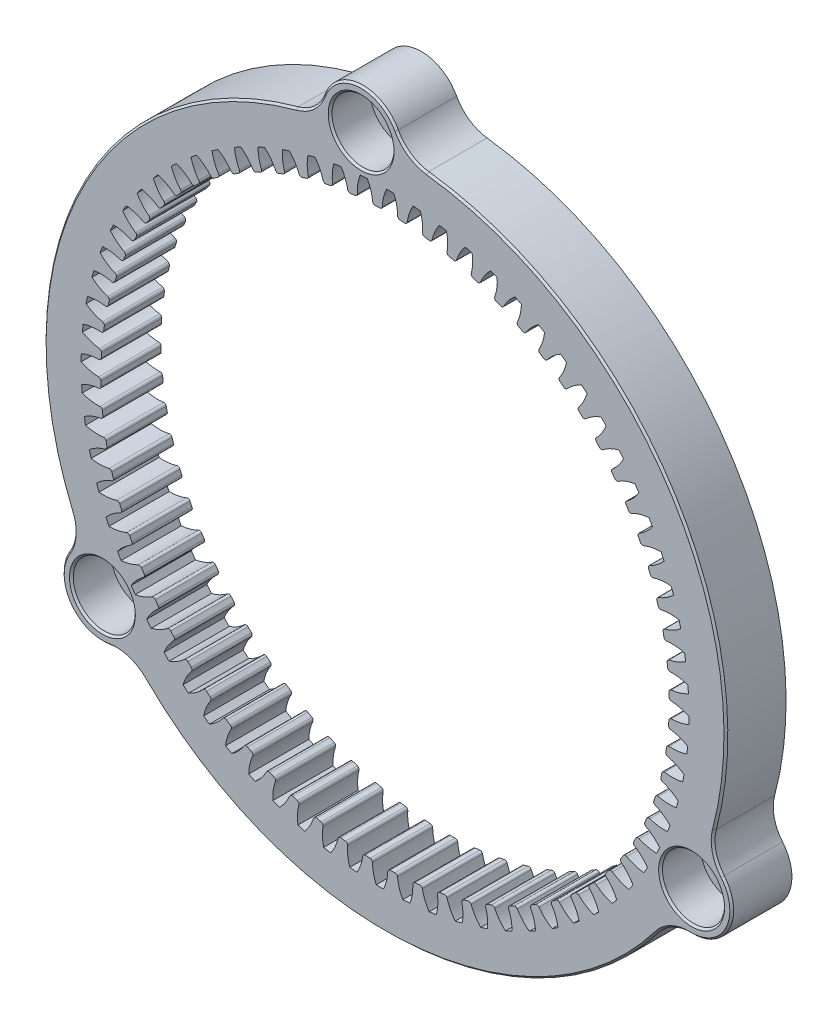
SolidWorks part; units mm, degrees
ref_plane "Front Plane" through (0, 0, 0) normal (0, 0, 1) x (1, 0, 0)
ref_plane "Top Plane" through (0, 0, 0) normal (0, 1, 0) x (1, 0, 0)
ref_plane "Right Plane" through (0, 0, 0) normal (1, 0, 0) x (0, 0, -1)
sketch "Sketch1" plane through (0, 0, 0) normal (0, 0, 1) x (1, 0, 0)
  circle A0 centre (0, 0) radius 46.8
  circle A1 centre (0, 0) radius 48.1
  circle A2 centre (0, 0) radius 44.98
  dimension "D1" = 93.6
  dimension "D2" = 96.2
  dimension "D3" = 3.12
extrude "Boss-Extrude1" add sketch "Sketch1" along normal mid plane 9.525 contours A2 | A0 A2 | A1 A0 region at (-45.4763, 0, 0) region at (-47.964, 0, 0) region at (0, 0, 0)
sketch "Sketch3" plane through (0, 0, 4.7625) normal (0, 0, 1) x (1, 0, 0)
  line L0 (0, 0) -> (0, 48.1) construction
  line L1 (-1.0209, 46.7889) -> (1.0209, 46.7889) construction
  line L2 (0, 0) -> (-0.7508, 44.9737) construction
  line L3 (0, 44.0346) -> (-1.8312, 49.0658) construction
  line L4 (0, 0) -> (2.0981, 48.0542) construction
  line L5 (1.0209, 46.7889) -> (3.0609, 46.6998) construction
  circle A0 centre (0, 0) radius 48.1 construction
  arc A1 (-2.1417, 49.0533) -> (-0.7508, 44.9737) centre (-7.773, 44.8565) cw
  arc A2 (2.1417, 49.0533) -> (0.7508, 44.9737) centre (7.773, 44.8565) ccw
  circle A3 centre (0, 0) radius 44.98 construction
  arc A4 (0.7508, 44.9737) -> (-0.7508, 44.9737) centre (0, 0) ccw
  circle A6 centre (0, 0) radius 46.8 construction
  circle A7 centre (0, 0) radius 49.1
  arc A8 (2.1417, 49.0533) -> (-2.1417, 49.0533) centre (0, 0) ccw
  circle A9 centre (0, 0) radius 48.1 construction
  point P20 (2.0409, 46.7443)
  dimension "D2" = 20
  dimension "D3" = 2.5
sketch "Sketch4" plane through (0, 0, 0) normal (0, 1, 0) x (1, 0, 0)
  line L0 (-1.2761, -4.7625) -> (0, 0)
  line L1 (-48.1, -4.7625) -> (48.1, -4.7625) construction
  line L3 (0, -3.4925) -> (0, 3.4925) construction
  line L4 (0, 0) -> (3.1205, 0) construction
  line L5 (-44.98, 0) -> (44.98, 0) construction
  line L6 (-1.2761, 4.7625) -> (0, 0)
  dimension "D1" = 15
curve "Curve1"
sketch "Sketch5" plane through (0, 0, 4.7625) normal (0, 0, 1) x (0.9996, 0.0265, 0)
  line L0 (0, 0) -> (0, 48.1) construction
  line L1 (-1.0209, 46.7889) -> (1.0209, 46.7889) construction
  line L2 (0, 0) -> (-0.7508, 44.9737) construction
  line L3 (0, 44.0346) -> (-1.8312, 49.0658) construction
  line L4 (0, 0) -> (2.0981, 48.0542) construction
  line L5 (1.0209, 46.7889) -> (3.0609, 46.6998) construction
  arc A1 (-2.1417, 49.0533) -> (-0.7508, 44.9737) centre (-7.773, 44.8565) cw
  arc A2 (2.1417, 49.0533) -> (0.7508, 44.9737) centre (7.773, 44.8565) ccw
  arc A4 (0.7508, 44.9737) -> (-0.7508, 44.9737) centre (0, 0) ccw
  arc A8 (2.1417, 49.0533) -> (-2.1417, 49.0533) centre (0, 0) ccw
  point P20 (2.0409, 46.7443)
extrude "Cut-Extrude2" cut sketch "Sketch5" against normal through all
fillet "Fillet3" radius 0.39 2 edges at (-1.9437, 44.938, 0) (-0.4426, 44.9778, 0)
pattern_circular "CirPattern3" count 72 over 360 about axis through (0, 0, 4.7625) along (0, 0, -1) of "Cut-Extrude2", "Fillet3"
sketch "Sketch11" plane through (0, 0, 4.7625) normal (0, 0, 1) x (1, 0, 0)
  line L0 (0, 0) -> (-3.3722, 47.9816) construction
  line L1 (-3.3722, 47.9816) -> (-3.7841, 53.8422) construction
  arc A0 (45.3854, -29.1659) -> (50.9377, -17.7719) centre (48.5208, -23.6439) ccw
  circle A1 centre (-3.7841, 53.8422) radius 3.275
  circle A2 centre (-3.7841, 53.8422) radius 4.9125
  arc A3 (2.5657, 53.8879) -> (-10.0779, 52.9993) centre (-3.7841, 53.8422) ccw
  arc A4 (-10.0779, 52.9993) -> (-47.9511, -24.722) centre (0, 0) ccw
  circle A5 centre (48.5208, -23.6439) radius 4.9125
  circle A6 centre (48.5208, -23.6439) radius 3.275
  arc A7 (-47.9511, -24.722) -> (-40.8597, -35.2274) centre (-44.7366, -30.1983) ccw
  circle A8 centre (-44.7366, -30.1983) radius 4.9125
  circle A9 centre (-44.7366, -30.1983) radius 3.275
  arc A10 (50.9377, -17.7719) -> (2.5657, 53.8879) centre (0, 0) ccw
  arc A12 (-40.8597, -35.2274) -> (45.3854, -29.1659) centre (0, 0) ccw
  arc A432 (-3.938, 47.9385) -> (-4.3871, 45.1353) centre (2.629, 45.449) ccw
  arc A433 (-4.7356, 44.73) -> (-4.3871, 45.1353) centre (-4.7767, 45.1178) ccw
  arc A434 (-4.7356, 44.73) -> (-5.4794, 44.645) centre (0, 0) ccw
  arc A435 (-5.9104, 44.9612) -> (-5.4794, 44.645) centre (-5.5269, 45.0321) ccw
  arc A436 (-5.9104, 44.9612) -> (-6.9804, 47.5908) centre (-12.8163, 43.6837) ccw
  arc A437 (-6.9804, 47.5908) -> (-8.1012, 47.4129) centre (0, 0) ccw
  arc A438 (-8.1012, 47.4129) -> (-8.3042, 44.5812) centre (-1.3421, 45.5052) ccw
  arc A439 (-8.6161, 44.1471) -> (-8.3042, 44.5812) centre (-8.6908, 44.5298) ccw
  arc A440 (-8.6161, 44.1471) -> (-9.3496, 43.9976) centre (0, 0) ccw
  arc A441 (-9.8065, 44.2749) -> (-9.3496, 43.9976) centre (-9.4307, 44.379) ccw
  arc A442 (-9.8065, 44.2749) -> (-11.1016, 46.8013) centre (-16.5748, 42.4005) ccw
  arc A443 (-11.1016, 46.8013) -> (-12.2026, 46.5264) centre (0, 0) ccw
  arc A444 (-12.2026, 46.5264) -> (-12.1581, 43.6878) centre (-5.3031, 45.2151) ccw
  arc A445 (-12.4309, 43.2281) -> (-12.1581, 43.6878) centre (-12.5387, 43.6029) ccw
  arc A446 (-12.4309, 43.2281) -> (-13.1487, 43.0153) centre (0, 0) ccw
  arc A447 (-13.628, 43.2518) -> (-13.1487, 43.0153) centre (-13.2627, 43.3882) ccw
  arc A448 (-13.628, 43.2518) -> (-15.1384, 45.6557) centre (-20.2072, 40.7945) ccw
  arc A449 (-15.1384, 45.6557) -> (-16.2112, 45.2858) centre (0, 0) ccw
  arc A450 (-16.2112, 45.2858) -> (-15.9194, 42.4619) centre (-9.2236, 44.5808) ccw
  arc A451 (-16.1512, 41.9802) -> (-15.9194, 42.4619) centre (-16.2913, 42.3442) ccw
  arc A452 (-16.1512, 41.9802) -> (-16.8477, 41.7056) centre (0, 0) ccw
  arc A453 (-17.3458, 41.8994) -> (-16.8477, 41.7056) centre (-16.9937, 42.0672) ccw
  arc A454 (-17.3458, 41.8994) -> (-19.0599, 44.1625) centre (-23.6858, 38.8781) ccw
  arc A455 (-19.0599, 44.1625) -> (-20.0965, 43.7006) centre (0, 0) ccw
  arc A456 (-20.0965, 43.7006) -> (-19.5597, 40.9128) centre (-13.074, 43.6073) ccw
  arc A457 (-19.7486, 40.4128) -> (-19.5597, 40.9128) centre (-19.9198, 40.7632) ccw
  arc A458 (-19.7486, 40.4128) -> (-20.4184, 40.0785) centre (0, 0) ccw
  arc A459 (-20.9316, 40.2282) -> (-20.4184, 40.0785) centre (-20.5955, 40.426) ccw
  arc A460 (-20.9316, 40.2282) -> (-22.8364, 42.3333) centre (-26.9841, 36.6658) ccw
  arc A461 (-22.8364, 42.3333) -> (-23.8288, 41.7828) centre (0, 0) ccw
  arc A462 (-23.8288, 41.7828) -> (-23.051, 39.0524) centre (-16.8249, 42.3019) ccw
  arc A463 (-23.1956, 38.5378) -> (-23.051, 39.0524) centre (-23.3968, 38.872) ccw
  arc A464 (-23.1956, 38.5378) -> (-23.8338, 38.1464) centre (0, 0) ccw
  arc A465 (-24.358, 38.2508) -> (-23.8338, 38.1464) centre (-24.0405, 38.4772) ccw
  arc A466 (-24.358, 38.2508) -> (-26.4391, 40.1819) centre (-30.0771, 34.1745) ccw
  arc A467 (-26.4391, 40.1819) -> (-27.3797, 39.547) centre (0, 0) ccw
  arc A468 (-27.3797, 39.547) -> (-26.3669, 36.8948) centre (-20.4477, 40.6745) ccw
  arc A469 (-26.4662, 36.3695) -> (-26.3669, 36.8948) centre (-26.6956, 36.6849) ccw
  arc A470 (-26.4662, 36.3695) -> (-27.0678, 35.924) centre (0, 0) ccw
  arc A471 (-27.5991, 35.9823) -> (-27.0678, 35.924) centre (-27.3025, 36.2355) ccw
  arc A472 (-27.5991, 35.9823) -> (-29.8406, 37.7247) centre (-32.9411, 31.423) ccw
  arc A473 (-29.8406, 37.7247) -> (-30.7222, 37.0102) centre (0, 0) ccw
  arc A474 (-30.7222, 37.0102) -> (-29.4822, 34.4563) centre (-23.9149, 38.7376) ccw
  arc A475 (-29.5353, 33.9245) -> (-29.4822, 34.4563) centre (-29.7913, 34.2186) ccw
  arc A476 (-29.5353, 33.9245) -> (-30.0958, 33.4282) centre (0, 0) ccw
  arc A477 (-30.6302, 33.44) -> (-30.0958, 33.4282) centre (-30.3567, 33.718) ccw
  arc A478 (-30.6302, 33.44) -> (-33.015, 34.9803) centre (-35.5545, 28.4324) ccw
  arc A479 (-33.015, 34.9803) -> (-33.831, 34.1917) centre (0, 0) ccw
  arc A480 (-33.831, 34.1917) -> (-32.3731, 31.7557) centre (-27.2001, 36.5059) ccw
  arc A481 (-32.3796, 31.2212) -> (-32.3731, 31.7557) centre (-32.6603, 31.4919) ccw
  arc A482 (-32.3796, 31.2212) -> (-32.8947, 30.678) centre (0, 0) ccw
  arc A483 (-33.4281, 30.6431) -> (-32.8947, 30.678) centre (-33.1799, 30.944) ccw
  arc A484 (-33.4281, 30.6431) -> (-35.9381, 31.9698) centre (-37.8972, 25.2255) ccw
  arc A485 (-35.9381, 31.9698) -> (-36.6823, 31.1131) centre (0, 0) ccw
  arc A486 (-36.6823, 31.1131) -> (-35.0176, 28.8133) centre (-30.2783, 33.9963) ccw
  arc A487 (-34.9775, 28.2803) -> (-35.0176, 28.8133) centre (-35.2807, 28.5255) ccw
  arc A488 (-34.9775, 28.2803) -> (-35.4433, 27.6943) centre (0, 0) ccw
  arc A489 (-35.9716, 27.6131) -> (-35.4433, 27.6943) centre (-35.7506, 27.9344) ccw
  arc A490 (-35.9716, 27.6131) -> (-38.5876, 28.7159) centre (-39.9516, 21.8265) ccw
  arc A491 (-38.5876, 28.7159) -> (-39.2543, 27.7976) centre (0, 0) ccw
  arc A492 (-39.2543, 27.7976) -> (-37.3956, 25.6517) centre (-33.1261, 31.228) ccw
  arc A493 (-37.3092, 25.1242) -> (-37.3956, 25.6517) centre (-37.6327, 25.3421) ccw
  arc A494 (-37.3092, 25.1242) -> (-37.7221, 24.4998) centre (0, 0) ccw
  arc A495 (-38.2414, 24.3728) -> (-37.7221, 24.4998) centre (-38.0492, 24.7122) ccw
  arc A496 (-38.2414, 24.3728) -> (-40.9436, 25.2435) centre (-41.7018, 18.2615) ccw
  arc A497 (-40.9436, 25.2435) -> (-41.5277, 24.2706) centre (0, 0) ccw
  arc A498 (-41.5277, 24.2706) -> (-39.489, 22.2949) centre (-35.7217, 28.222) ccw
  arc A499 (-39.3569, 21.7769) -> (-39.489, 22.2949) centre (-39.6982, 21.9657) ccw
  arc A500 (-39.3569, 21.7769) -> (-39.7139, 21.1189) centre (0, 0) ccw
  arc A501 (-40.2201, 20.9471) -> (-39.7139, 21.1189) centre (-40.0582, 21.302) ccw
  arc A502 (-40.2201, 20.9471) -> (-42.9879, 21.579) centre (-43.1347, 14.5574) ccw
  arc A503 (-42.9879, 21.579) -> (-43.485, 20.5588) centre (0, 0) ccw
  arc A504 (-43.485, 20.5588) -> (-41.2818, 18.7683) centre (-38.0455, 25.0013) ccw
  arc A505 (-41.1051, 18.2639) -> (-41.2818, 18.7683) centre (-41.4615, 18.4222) ccw
  arc A506 (-41.1051, 18.2639) -> (-41.4034, 17.5772) centre (0, 0) ccw
  arc A507 (-41.8927, 17.362) -> (-41.4034, 17.5772) centre (-41.7624, 17.7296) ccw
  arc A508 (-41.8927, 17.362) -> (-44.705, 17.7502) centre (-44.2394, 10.7426) ccw
  arc A509 (-44.705, 17.7502) -> (-45.1113, 16.6906) centre (0, 0) ccw
  arc A510 (-45.1113, 16.6906) -> (-42.7605, 15.099) centre (-40.0797, 21.5903) ccw
  arc A511 (-42.5405, 14.6118) -> (-42.7605, 15.099) centre (-42.9094, 14.7385) ccw
  arc A512 (-42.5405, 14.6118) -> (-42.7778, 13.9018) centre (0, 0) ccw
  arc A513 (-43.2465, 13.6448) -> (-42.7778, 13.9018) centre (-43.1487, 14.0223) ccw
  arc A514 (-43.2465, 13.6448) -> (-46.0819, 13.7864) centre (-45.0073, 6.846) ccw
  arc A515 (-46.0819, 13.7864) -> (-46.3944, 12.6954) centre (0, 0) ccw
  arc A516 (-46.3944, 12.6954) -> (-43.9137, 11.3147) centre (-41.8089, 18.0149) ccw
  arc A517 (-43.6521, 10.8486) -> (-43.9137, 11.3147) centre (-44.0306, 10.9426) ccw
  arc A518 (-43.6521, 10.8486) -> (-43.8266, 10.1205) centre (0, 0) ccw
  arc A519 (-44.2711, 9.8237) -> (-43.8266, 10.1205) centre (-44.2066, 10.2083) ccw
  arc A520 (-44.2711, 9.8237) -> (-47.1082, 9.7176) centre (-45.4327, 2.8973) ccw
  arc A521 (-47.1082, 9.7176) -> (-47.3243, 8.6036) centre (0, 0) ccw
  arc A522 (-47.3243, 8.6036) -> (-44.7328, 7.4443) centre (-43.2199, 14.3025) ccw
  arc A523 (-44.4315, 7.0027) -> (-44.7328, 7.4443) centre (-44.8168, 7.0635) ccw
  arc A524 (-44.4315, 7.0027) -> (-44.5419, 6.2623) centre (0, 0) ccw
  arc A525 (-44.9589, 5.9278) -> (-44.5419, 6.2623) centre (-44.9281, 6.3166) ccw
  arc A526 (-44.9589, 5.9278) -> (-47.7758, 5.5749) centre (-45.5123, -1.0734) ccw
  arc A527 (-47.7758, 5.5749) -> (-47.8941, 4.4462) centre (0, 0) ccw
  arc A528 (-47.8941, 4.4462) -> (-45.2114, 3.5173) centre (-44.302, 10.4812) ccw
  arc A529 (-44.8728, 3.1036) -> (-45.2114, 3.5173) centre (-45.2619, 3.1305) ccw
  arc A530 (-44.8728, 3.1036) -> (-44.9182, 2.3564) centre (0, 0) ccw
  arc A531 (-45.3044, 1.9868) -> (-44.9182, 2.3564) centre (-45.3077, 2.3768) ccw
  arc A532 (-45.3044, 1.9868) -> (-48.0799, 1.3897) centre (-45.2456, -5.036) ccw
  arc A533 (-48.0799, 1.3897) -> (-48.0993, 0.2551) centre (0, 0) ccw
  arc A534 (-48.0993, 0.2551) -> (-45.3459, -0.4366) centre (-45.0469, 6.5802) ccw
  arc A535 (-44.9725, -0.8191) -> (-45.3459, -0.4366) centre (-45.3625, -0.8262) ccw
  arc A536 (-44.9725, -0.8191) -> (-44.9527, -1.5675) centre (0, 0) ccw
  arc A537 (-45.3052, -1.9693) -> (-44.9527, -1.5675) centre (-45.3424, -1.5811) ccw
  arc A538 (-45.3052, -1.9693) -> (-48.0181, -2.806) centre (-44.6345, -8.9603) ccw
  arc A539 (-48.0181, -2.806) -> (-47.9385, -3.938) centre (0, 0) ccw
  arc A540 (-47.9385, -3.938) -> (-45.1353, -4.3871) centre (-45.449, 2.629) ccw
  arc A541 (-44.73, -4.7356) -> (-45.1353, -4.3871) centre (-45.1178, -4.7767) ccw
  arc A542 (-44.73, -4.7356) -> (-44.645, -5.4794) centre (0, 0) ccw
  arc A543 (-44.9612, -5.9104) -> (-44.645, -5.4794) centre (-45.0321, -5.5269) ccw
  arc A544 (-44.9612, -5.9104) -> (-47.5908, -6.9804) centre (-43.6837, -12.8163) ccw
  arc A545 (-47.5908, -6.9804) -> (-47.4129, -8.1012) centre (0, 0) ccw
  arc A546 (-47.4129, -8.1012) -> (-44.5812, -8.3042) centre (-45.5052, -1.3421) ccw
  arc A547 (-44.1471, -8.6161) -> (-44.5812, -8.3042) centre (-44.5298, -8.6908) ccw
  arc A548 (-44.1471, -8.6161) -> (-43.9976, -9.3496) centre (0, 0) ccw
  arc A549 (-44.2749, -9.8065) -> (-43.9976, -9.3496) centre (-44.379, -9.4307) ccw
  arc A550 (-44.2749, -9.8065) -> (-46.8013, -11.1016) centre (-42.4005, -16.5748) ccw
  arc A551 (-46.8013, -11.1016) -> (-46.5264, -12.2026) centre (0, 0) ccw
  arc A552 (-46.5264, -12.2026) -> (-43.6878, -12.1581) centre (-45.2151, -5.3031) ccw
  arc A553 (-43.2281, -12.4309) -> (-43.6878, -12.1581) centre (-43.6029, -12.5387) ccw
  arc A554 (-43.2281, -12.4309) -> (-43.0153, -13.1487) centre (0, 0) ccw
  arc A555 (-43.2518, -13.628) -> (-43.0153, -13.1487) centre (-43.3882, -13.2627) ccw
  arc A556 (-43.2518, -13.628) -> (-45.6557, -15.1384) centre (-40.7945, -20.2072) ccw
  arc A557 (-45.6557, -15.1384) -> (-45.2858, -16.2112) centre (0, 0) ccw
  arc A558 (-45.2858, -16.2112) -> (-42.4619, -15.9194) centre (-44.5808, -9.2236) ccw
  arc A559 (-41.9802, -16.1512) -> (-42.4619, -15.9194) centre (-42.3442, -16.2913) ccw
  arc A560 (-41.9802, -16.1512) -> (-41.7056, -16.8477) centre (0, 0) ccw
  arc A561 (-41.8994, -17.3458) -> (-41.7056, -16.8477) centre (-42.0672, -16.9937) ccw
  arc A562 (-41.8994, -17.3458) -> (-44.1625, -19.0599) centre (-38.8781, -23.6858) ccw
  arc A563 (-44.1625, -19.0599) -> (-43.7006, -20.0965) centre (0, 0) ccw
  arc A564 (-43.7006, -20.0965) -> (-40.9128, -19.5597) centre (-43.6073, -13.074) ccw
  arc A565 (-40.4128, -19.7486) -> (-40.9128, -19.5597) centre (-40.7632, -19.9198) ccw
  arc A566 (-40.4128, -19.7486) -> (-40.0785, -20.4184) centre (0, 0) ccw
  arc A567 (-40.2282, -20.9316) -> (-40.0785, -20.4184) centre (-40.426, -20.5955) ccw
  arc A568 (-40.2282, -20.9316) -> (-42.3333, -22.8364) centre (-36.6658, -26.9841) ccw
  arc A569 (-42.3333, -22.8364) -> (-41.7828, -23.8288) centre (0, 0) ccw
  arc A570 (-41.7828, -23.8288) -> (-39.0524, -23.051) centre (-42.3019, -16.8249) ccw
  arc A571 (-38.5378, -23.1956) -> (-39.0524, -23.051) centre (-38.872, -23.3968) ccw
  arc A572 (-38.5378, -23.1956) -> (-38.1464, -23.8338) centre (0, 0) ccw
  arc A573 (-38.2508, -24.358) -> (-38.1464, -23.8338) centre (-38.4772, -24.0405) ccw
  arc A574 (-38.2508, -24.358) -> (-40.1819, -26.4391) centre (-34.1745, -30.0771) ccw
  arc A575 (-40.1819, -26.4391) -> (-39.547, -27.3797) centre (0, 0) ccw
  arc A576 (-39.547, -27.3797) -> (-36.8948, -26.3669) centre (-40.6745, -20.4477) ccw
  arc A577 (-36.3695, -26.4662) -> (-36.8948, -26.3669) centre (-36.6849, -26.6956) ccw
  arc A578 (-36.3695, -26.4662) -> (-35.924, -27.0678) centre (0, 0) ccw
  arc A579 (-35.9823, -27.5991) -> (-35.924, -27.0678) centre (-36.2355, -27.3025) ccw
  arc A580 (-35.9823, -27.5991) -> (-37.7247, -29.8406) centre (-31.423, -32.9411) ccw
  arc A581 (-37.7247, -29.8406) -> (-37.0102, -30.7222) centre (0, 0) ccw
  arc A582 (-37.0102, -30.7222) -> (-34.4563, -29.4822) centre (-38.7376, -23.9149) ccw
  arc A583 (-33.9245, -29.5353) -> (-34.4563, -29.4822) centre (-34.2186, -29.7913) ccw
  arc A584 (-33.9245, -29.5353) -> (-33.4282, -30.0958) centre (0, 0) ccw
  arc A585 (-33.44, -30.6302) -> (-33.4282, -30.0958) centre (-33.718, -30.3567) ccw
  arc A586 (-33.44, -30.6302) -> (-34.9803, -33.015) centre (-28.4324, -35.5545) ccw
  arc A587 (-34.9803, -33.015) -> (-34.1917, -33.831) centre (0, 0) ccw
  arc A588 (-34.1917, -33.831) -> (-31.7557, -32.3731) centre (-36.5059, -27.2001) ccw
  arc A589 (-31.2212, -32.3796) -> (-31.7557, -32.3731) centre (-31.4919, -32.6603) ccw
  arc A590 (-31.2212, -32.3796) -> (-30.678, -32.8947) centre (0, 0) ccw
  arc A591 (-30.6431, -33.4281) -> (-30.678, -32.8947) centre (-30.944, -33.1799) ccw
  arc A592 (-30.6431, -33.4281) -> (-31.9698, -35.9381) centre (-25.2255, -37.8972) ccw
  arc A593 (-31.9698, -35.9381) -> (-31.1131, -36.6823) centre (0, 0) ccw
  arc A594 (-31.1131, -36.6823) -> (-28.8133, -35.0176) centre (-33.9963, -30.2783) ccw
  arc A595 (-28.2803, -34.9775) -> (-28.8133, -35.0176) centre (-28.5255, -35.2807) ccw
  arc A596 (-28.2803, -34.9775) -> (-27.6943, -35.4433) centre (0, 0) ccw
  arc A597 (-27.6131, -35.9716) -> (-27.6943, -35.4433) centre (-27.9344, -35.7506) ccw
  arc A598 (-27.6131, -35.9716) -> (-28.7159, -38.5876) centre (-21.8265, -39.9516) ccw
  arc A599 (-28.7159, -38.5876) -> (-27.7976, -39.2543) centre (0, 0) ccw
  arc A600 (-27.7976, -39.2543) -> (-25.6517, -37.3956) centre (-31.228, -33.1261) ccw
  arc A601 (-25.1242, -37.3092) -> (-25.6517, -37.3956) centre (-25.3421, -37.6327) ccw
  arc A602 (-25.1242, -37.3092) -> (-24.4998, -37.7221) centre (0, 0) ccw
  arc A603 (-24.3728, -38.2414) -> (-24.4998, -37.7221) centre (-24.7122, -38.0492) ccw
  arc A604 (-24.3728, -38.2414) -> (-25.2435, -40.9436) centre (-18.2615, -41.7018) ccw
  arc A605 (-25.2435, -40.9436) -> (-24.2706, -41.5277) centre (0, 0) ccw
  arc A606 (-24.2706, -41.5277) -> (-22.2949, -39.489) centre (-28.222, -35.7217) ccw
  arc A607 (-21.7769, -39.3569) -> (-22.2949, -39.489) centre (-21.9657, -39.6982) ccw
  arc A608 (-21.7769, -39.3569) -> (-21.1189, -39.7139) centre (0, 0) ccw
  arc A609 (-20.9471, -40.2201) -> (-21.1189, -39.7139) centre (-21.302, -40.0582) ccw
  arc A610 (-20.9471, -40.2201) -> (-21.579, -42.9879) centre (-14.5574, -43.1347) ccw
  arc A611 (-21.579, -42.9879) -> (-20.5588, -43.485) centre (0, 0) ccw
  arc A612 (-20.5588, -43.485) -> (-18.7683, -41.2818) centre (-25.0013, -38.0455) ccw
  arc A613 (-18.2639, -41.1051) -> (-18.7683, -41.2818) centre (-18.4222, -41.4615) ccw
  arc A614 (-18.2639, -41.1051) -> (-17.5772, -41.4034) centre (0, 0) ccw
  arc A615 (-17.362, -41.8927) -> (-17.5772, -41.4034) centre (-17.7296, -41.7624) ccw
  arc A616 (-17.362, -41.8927) -> (-17.7502, -44.705) centre (-10.7426, -44.2394) ccw
  arc A617 (-17.7502, -44.705) -> (-16.6906, -45.1113) centre (0, 0) ccw
  arc A618 (-16.6906, -45.1113) -> (-15.099, -42.7605) centre (-21.5903, -40.0797) ccw
  arc A619 (-14.6118, -42.5405) -> (-15.099, -42.7605) centre (-14.7385, -42.9094) ccw
  arc A620 (-14.6118, -42.5405) -> (-13.9018, -42.7778) centre (0, 0) ccw
  arc A621 (-13.6448, -43.2465) -> (-13.9018, -42.7778) centre (-14.0223, -43.1487) ccw
  arc A622 (-13.6448, -43.2465) -> (-13.7864, -46.0819) centre (-6.846, -45.0073) ccw
  arc A623 (-13.7864, -46.0819) -> (-12.6954, -46.3944) centre (0, 0) ccw
  arc A624 (-12.6954, -46.3944) -> (-11.3147, -43.9137) centre (-18.0149, -41.8089) ccw
  arc A625 (-10.8486, -43.6521) -> (-11.3147, -43.9137) centre (-10.9426, -44.0306) ccw
  arc A626 (-10.8486, -43.6521) -> (-10.1205, -43.8266) centre (0, 0) ccw
  arc A627 (-9.8237, -44.2711) -> (-10.1205, -43.8266) centre (-10.2083, -44.2066) ccw
  arc A628 (-9.8237, -44.2711) -> (-9.7176, -47.1082) centre (-2.8973, -45.4327) ccw
  arc A629 (-9.7176, -47.1082) -> (-8.6036, -47.3243) centre (0, 0) ccw
  arc A630 (-8.6036, -47.3243) -> (-7.4443, -44.7328) centre (-14.3025, -43.2199) ccw
  arc A631 (-7.0027, -44.4315) -> (-7.4443, -44.7328) centre (-7.0635, -44.8168) ccw
  arc A632 (-7.0027, -44.4315) -> (-6.2623, -44.5419) centre (0, 0) ccw
  arc A633 (-5.9278, -44.9589) -> (-6.2623, -44.5419) centre (-6.3166, -44.9281) ccw
  arc A634 (-5.9278, -44.9589) -> (-5.5749, -47.7758) centre (1.0734, -45.5123) ccw
  arc A635 (-5.5749, -47.7758) -> (-4.4462, -47.8941) centre (0, 0) ccw
  arc A636 (-4.4462, -47.8941) -> (-3.5173, -45.2114) centre (-10.4812, -44.302) ccw
  arc A637 (-3.1036, -44.8728) -> (-3.5173, -45.2114) centre (-3.1305, -45.2619) ccw
  arc A638 (-3.1036, -44.8728) -> (-2.3564, -44.9182) centre (0, 0) ccw
  arc A639 (-1.9868, -45.3044) -> (-2.3564, -44.9182) centre (-2.3768, -45.3077) ccw
  arc A640 (-1.9868, -45.3044) -> (-1.3897, -48.0799) centre (5.036, -45.2456) ccw
  arc A641 (-1.3897, -48.0799) -> (-0.2551, -48.0993) centre (0, 0) ccw
  arc A642 (-0.2551, -48.0993) -> (0.4366, -45.3459) centre (-6.5802, -45.0469) ccw
  arc A643 (0.8191, -44.9725) -> (0.4366, -45.3459) centre (0.8262, -45.3625) ccw
  arc A644 (0.8191, -44.9725) -> (1.5675, -44.9527) centre (0, 0) ccw
  arc A645 (1.9693, -45.3052) -> (1.5675, -44.9527) centre (1.5811, -45.3424) ccw
  arc A646 (1.9693, -45.3052) -> (2.806, -48.0181) centre (8.9603, -44.6345) ccw
  arc A647 (2.806, -48.0181) -> (3.938, -47.9385) centre (0, 0) ccw
  arc A648 (3.938, -47.9385) -> (4.3871, -45.1353) centre (-2.629, -45.449) ccw
  arc A649 (4.7356, -44.73) -> (4.3871, -45.1353) centre (4.7767, -45.1178) ccw
  arc A650 (4.7356, -44.73) -> (5.4794, -44.645) centre (0, 0) ccw
  arc A651 (5.9104, -44.9612) -> (5.4794, -44.645) centre (5.5269, -45.0321) ccw
  arc A652 (5.9104, -44.9612) -> (6.9804, -47.5908) centre (12.8163, -43.6837) ccw
  arc A653 (6.9804, -47.5908) -> (8.1012, -47.4129) centre (0, 0) ccw
  arc A654 (8.1012, -47.4129) -> (8.3042, -44.5812) centre (1.3421, -45.5052) ccw
  arc A655 (8.6161, -44.1471) -> (8.3042, -44.5812) centre (8.6908, -44.5298) ccw
  arc A656 (8.6161, -44.1471) -> (9.3496, -43.9976) centre (0, 0) ccw
  arc A657 (9.8065, -44.2749) -> (9.3496, -43.9976) centre (9.4307, -44.379) ccw
  arc A658 (9.8065, -44.2749) -> (11.1016, -46.8013) centre (16.5748, -42.4005) ccw
  arc A659 (11.1016, -46.8013) -> (12.2026, -46.5264) centre (0, 0) ccw
  arc A660 (12.2026, -46.5264) -> (12.1581, -43.6878) centre (5.3031, -45.2151) ccw
  arc A661 (12.4309, -43.2281) -> (12.1581, -43.6878) centre (12.5387, -43.6029) ccw
  arc A662 (12.4309, -43.2281) -> (13.1487, -43.0153) centre (0, 0) ccw
  arc A663 (13.628, -43.2518) -> (13.1487, -43.0153) centre (13.2627, -43.3882) ccw
  arc A664 (13.628, -43.2518) -> (15.1384, -45.6557) centre (20.2072, -40.7945) ccw
  arc A665 (15.1384, -45.6557) -> (16.2112, -45.2858) centre (0, 0) ccw
  arc A666 (16.2112, -45.2858) -> (15.9194, -42.4619) centre (9.2236, -44.5808) ccw
  arc A667 (16.1512, -41.9802) -> (15.9194, -42.4619) centre (16.2913, -42.3442) ccw
  arc A668 (16.1512, -41.9802) -> (16.8477, -41.7056) centre (0, 0) ccw
  arc A669 (17.3458, -41.8994) -> (16.8477, -41.7056) centre (16.9937, -42.0672) ccw
  arc A670 (17.3458, -41.8994) -> (19.0599, -44.1625) centre (23.6858, -38.8781) ccw
  arc A671 (19.0599, -44.1625) -> (20.0965, -43.7006) centre (0, 0) ccw
  arc A672 (20.0965, -43.7006) -> (19.5597, -40.9128) centre (13.074, -43.6073) ccw
  arc A673 (19.7486, -40.4128) -> (19.5597, -40.9128) centre (19.9198, -40.7632) ccw
  arc A674 (19.7486, -40.4128) -> (20.4184, -40.0785) centre (0, 0) ccw
  arc A675 (20.9316, -40.2282) -> (20.4184, -40.0785) centre (20.5955, -40.426) ccw
  arc A676 (20.9316, -40.2282) -> (22.8364, -42.3333) centre (26.9841, -36.6658) ccw
  arc A677 (22.8364, -42.3333) -> (23.8288, -41.7828) centre (0, 0) ccw
  arc A678 (23.8288, -41.7828) -> (23.051, -39.0524) centre (16.8249, -42.3019) ccw
  arc A679 (23.1956, -38.5378) -> (23.051, -39.0524) centre (23.3968, -38.872) ccw
  arc A680 (23.1956, -38.5378) -> (23.8338, -38.1464) centre (0, 0) ccw
  arc A681 (24.358, -38.2508) -> (23.8338, -38.1464) centre (24.0405, -38.4772) ccw
  arc A682 (24.358, -38.2508) -> (26.4391, -40.1819) centre (30.0771, -34.1745) ccw
  arc A683 (26.4391, -40.1819) -> (27.3797, -39.547) centre (0, 0) ccw
  arc A684 (27.3797, -39.547) -> (26.3669, -36.8948) centre (20.4477, -40.6745) ccw
  arc A685 (26.4662, -36.3695) -> (26.3669, -36.8948) centre (26.6956, -36.6849) ccw
  arc A686 (26.4662, -36.3695) -> (27.0678, -35.924) centre (0, 0) ccw
  arc A687 (27.5991, -35.9823) -> (27.0678, -35.924) centre (27.3025, -36.2355) ccw
  arc A688 (27.5991, -35.9823) -> (29.8406, -37.7247) centre (32.9411, -31.423) ccw
  arc A689 (29.8406, -37.7247) -> (30.7222, -37.0102) centre (0, 0) ccw
  arc A690 (30.7222, -37.0102) -> (29.4822, -34.4563) centre (23.9149, -38.7376) ccw
  arc A691 (29.5353, -33.9245) -> (29.4822, -34.4563) centre (29.7913, -34.2186) ccw
  arc A692 (29.5353, -33.9245) -> (30.0958, -33.4282) centre (0, 0) ccw
  arc A693 (30.6302, -33.44) -> (30.0958, -33.4282) centre (30.3567, -33.718) ccw
  arc A694 (30.6302, -33.44) -> (33.015, -34.9803) centre (35.5545, -28.4324) ccw
  arc A695 (33.015, -34.9803) -> (33.831, -34.1917) centre (0, 0) ccw
  arc A696 (33.831, -34.1917) -> (32.3731, -31.7557) centre (27.2001, -36.5059) ccw
  arc A697 (32.3796, -31.2212) -> (32.3731, -31.7557) centre (32.6603, -31.4919) ccw
  arc A698 (32.3796, -31.2212) -> (32.8947, -30.678) centre (0, 0) ccw
  arc A699 (33.4281, -30.6431) -> (32.8947, -30.678) centre (33.1799, -30.944) ccw
  arc A700 (33.4281, -30.6431) -> (35.9381, -31.9698) centre (37.8972, -25.2255) ccw
  arc A701 (35.9381, -31.9698) -> (36.6823, -31.1131) centre (0, 0) ccw
  arc A702 (36.6823, -31.1131) -> (35.0176, -28.8133) centre (30.2783, -33.9963) ccw
  arc A703 (34.9775, -28.2803) -> (35.0176, -28.8133) centre (35.2807, -28.5255) ccw
  arc A704 (34.9775, -28.2803) -> (35.4433, -27.6943) centre (0, 0) ccw
  arc A705 (35.9716, -27.6131) -> (35.4433, -27.6943) centre (35.7506, -27.9344) ccw
  arc A706 (35.9716, -27.6131) -> (38.5876, -28.7159) centre (39.9516, -21.8265) ccw
  arc A707 (38.5876, -28.7159) -> (39.2543, -27.7976) centre (0, 0) ccw
  arc A708 (39.2543, -27.7976) -> (37.3956, -25.6517) centre (33.1261, -31.228) ccw
  arc A709 (37.3092, -25.1242) -> (37.3956, -25.6517) centre (37.6327, -25.3421) ccw
  arc A710 (37.3092, -25.1242) -> (37.7221, -24.4998) centre (0, 0) ccw
  arc A711 (38.2414, -24.3728) -> (37.7221, -24.4998) centre (38.0492, -24.7122) ccw
  arc A712 (38.2414, -24.3728) -> (40.9436, -25.2435) centre (41.7018, -18.2615) ccw
  arc A713 (40.9436, -25.2435) -> (41.5277, -24.2706) centre (0, 0) ccw
  arc A714 (41.5277, -24.2706) -> (39.489, -22.2949) centre (35.7217, -28.222) ccw
  arc A715 (39.3569, -21.7769) -> (39.489, -22.2949) centre (39.6982, -21.9657) ccw
  arc A716 (39.3569, -21.7769) -> (39.7139, -21.1189) centre (0, 0) ccw
  arc A717 (40.2201, -20.9471) -> (39.7139, -21.1189) centre (40.0582, -21.302) ccw
  arc A718 (40.2201, -20.9471) -> (42.9879, -21.579) centre (43.1347, -14.5574) ccw
  arc A719 (42.9879, -21.579) -> (43.485, -20.5588) centre (0, 0) ccw
  arc A720 (43.485, -20.5588) -> (41.2818, -18.7683) centre (38.0455, -25.0013) ccw
  arc A721 (41.1051, -18.2639) -> (41.2818, -18.7683) centre (41.4615, -18.4222) ccw
  arc A722 (41.1051, -18.2639) -> (41.4034, -17.5772) centre (0, 0) ccw
  arc A723 (41.8927, -17.362) -> (41.4034, -17.5772) centre (41.7624, -17.7296) ccw
  arc A724 (41.8927, -17.362) -> (44.705, -17.7502) centre (44.2394, -10.7426) ccw
  arc A725 (44.705, -17.7502) -> (45.1113, -16.6906) centre (0, 0) ccw
  arc A726 (45.1113, -16.6906) -> (42.7605, -15.099) centre (40.0797, -21.5903) ccw
  arc A727 (42.5405, -14.6118) -> (42.7605, -15.099) centre (42.9094, -14.7385) ccw
  arc A728 (42.5405, -14.6118) -> (42.7778, -13.9018) centre (0, 0) ccw
  arc A729 (43.2465, -13.6448) -> (42.7778, -13.9018) centre (43.1487, -14.0223) ccw
  arc A730 (43.2465, -13.6448) -> (46.0819, -13.7864) centre (45.0073, -6.846) ccw
  arc A731 (46.0819, -13.7864) -> (46.3944, -12.6954) centre (0, 0) ccw
  arc A732 (46.3944, -12.6954) -> (43.9137, -11.3147) centre (41.8089, -18.0149) ccw
  arc A733 (43.6521, -10.8486) -> (43.9137, -11.3147) centre (44.0306, -10.9426) ccw
  arc A734 (43.6521, -10.8486) -> (43.8266, -10.1205) centre (0, 0) ccw
  arc A735 (44.2711, -9.8237) -> (43.8266, -10.1205) centre (44.2066, -10.2083) ccw
  arc A736 (44.2711, -9.8237) -> (47.1082, -9.7176) centre (45.4327, -2.8973) ccw
  arc A737 (47.1082, -9.7176) -> (47.3243, -8.6036) centre (0, 0) ccw
  arc A738 (47.3243, -8.6036) -> (44.7328, -7.4443) centre (43.2199, -14.3025) ccw
  arc A739 (44.4315, -7.0027) -> (44.7328, -7.4443) centre (44.8168, -7.0635) ccw
  arc A740 (44.4315, -7.0027) -> (44.5419, -6.2623) centre (0, 0) ccw
  arc A741 (44.9589, -5.9278) -> (44.5419, -6.2623) centre (44.9281, -6.3166) ccw
  arc A742 (44.9589, -5.9278) -> (47.7758, -5.5749) centre (45.5123, 1.0734) ccw
  arc A743 (47.7758, -5.5749) -> (47.8941, -4.4462) centre (0, 0) ccw
  arc A744 (47.8941, -4.4462) -> (45.2114, -3.5173) centre (44.302, -10.4812) ccw
  arc A745 (44.8728, -3.1036) -> (45.2114, -3.5173) centre (45.2619, -3.1305) ccw
  arc A746 (44.8728, -3.1036) -> (44.9182, -2.3564) centre (0, 0) ccw
  arc A747 (45.3044, -1.9868) -> (44.9182, -2.3564) centre (45.3077, -2.3768) ccw
  arc A748 (45.3044, -1.9868) -> (48.0799, -1.3897) centre (45.2456, 5.036) ccw
  arc A749 (48.0799, -1.3897) -> (48.0993, -0.2551) centre (0, 0) ccw
  arc A750 (48.0993, -0.2551) -> (45.3459, 0.4366) centre (45.0469, -6.5802) ccw
  arc A751 (44.9725, 0.8191) -> (45.3459, 0.4366) centre (45.3625, 0.8262) ccw
  arc A752 (44.9725, 0.8191) -> (44.9527, 1.5675) centre (0, 0) ccw
  arc A753 (45.3052, 1.9693) -> (44.9527, 1.5675) centre (45.3424, 1.5811) ccw
  arc A754 (45.3052, 1.9693) -> (48.0181, 2.806) centre (44.6345, 8.9603) ccw
  arc A755 (48.0181, 2.806) -> (47.9385, 3.938) centre (0, 0) ccw
  arc A756 (47.9385, 3.938) -> (45.1353, 4.3871) centre (45.449, -2.629) ccw
  arc A757 (44.73, 4.7356) -> (45.1353, 4.3871) centre (45.1178, 4.7767) ccw
  arc A758 (44.73, 4.7356) -> (44.645, 5.4794) centre (0, 0) ccw
  arc A759 (44.9612, 5.9104) -> (44.645, 5.4794) centre (45.0321, 5.5269) ccw
  arc A760 (44.9612, 5.9104) -> (47.5908, 6.9804) centre (43.6837, 12.8163) ccw
  arc A761 (47.5908, 6.9804) -> (47.4129, 8.1012) centre (0, 0) ccw
  arc A762 (47.4129, 8.1012) -> (44.5812, 8.3042) centre (45.5052, 1.3421) ccw
  arc A763 (44.1471, 8.6161) -> (44.5812, 8.3042) centre (44.5298, 8.6908) ccw
  arc A764 (44.1471, 8.6161) -> (43.9976, 9.3496) centre (0, 0) ccw
  arc A765 (44.2749, 9.8065) -> (43.9976, 9.3496) centre (44.379, 9.4307) ccw
  arc A766 (44.2749, 9.8065) -> (46.8013, 11.1016) centre (42.4005, 16.5748) ccw
  arc A767 (46.8013, 11.1016) -> (46.5264, 12.2026) centre (0, 0) ccw
  arc A768 (46.5264, 12.2026) -> (43.6878, 12.1581) centre (45.2151, 5.3031) ccw
  arc A769 (43.2281, 12.4309) -> (43.6878, 12.1581) centre (43.6029, 12.5387) ccw
  arc A770 (43.2281, 12.4309) -> (43.0153, 13.1487) centre (0, 0) ccw
  arc A771 (43.2518, 13.628) -> (43.0153, 13.1487) centre (43.3882, 13.2627) ccw
  arc A772 (43.2518, 13.628) -> (45.6557, 15.1384) centre (40.7945, 20.2072) ccw
  arc A773 (45.6557, 15.1384) -> (45.2858, 16.2112) centre (0, 0) ccw
  arc A774 (45.2858, 16.2112) -> (42.4619, 15.9194) centre (44.5808, 9.2236) ccw
  arc A775 (41.9802, 16.1512) -> (42.4619, 15.9194) centre (42.3442, 16.2913) ccw
  arc A776 (41.9802, 16.1512) -> (41.7056, 16.8477) centre (0, 0) ccw
  arc A777 (41.8994, 17.3458) -> (41.7056, 16.8477) centre (42.0672, 16.9937) ccw
  arc A778 (41.8994, 17.3458) -> (44.1625, 19.0599) centre (38.8781, 23.6858) ccw
  arc A779 (44.1625, 19.0599) -> (43.7006, 20.0965) centre (0, 0) ccw
  arc A780 (43.7006, 20.0965) -> (40.9128, 19.5597) centre (43.6073, 13.074) ccw
  arc A781 (40.4128, 19.7486) -> (40.9128, 19.5597) centre (40.7632, 19.9198) ccw
  arc A782 (40.4128, 19.7486) -> (40.0785, 20.4184) centre (0, 0) ccw
  arc A783 (40.2282, 20.9316) -> (40.0785, 20.4184) centre (40.426, 20.5955) ccw
  arc A784 (40.2282, 20.9316) -> (42.3333, 22.8364) centre (36.6658, 26.9841) ccw
  arc A785 (42.3333, 22.8364) -> (41.7828, 23.8288) centre (0, 0) ccw
  arc A786 (41.7828, 23.8288) -> (39.0524, 23.051) centre (42.3019, 16.8249) ccw
  arc A787 (38.5378, 23.1956) -> (39.0524, 23.051) centre (38.872, 23.3968) ccw
  arc A788 (38.5378, 23.1956) -> (38.1464, 23.8338) centre (0, 0) ccw
  arc A789 (38.2508, 24.358) -> (38.1464, 23.8338) centre (38.4772, 24.0405) ccw
  arc A790 (38.2508, 24.358) -> (40.1819, 26.4391) centre (34.1745, 30.0771) ccw
  arc A791 (40.1819, 26.4391) -> (39.547, 27.3797) centre (0, 0) ccw
  arc A792 (39.547, 27.3797) -> (36.8948, 26.3669) centre (40.6745, 20.4477) ccw
  arc A793 (36.3695, 26.4662) -> (36.8948, 26.3669) centre (36.6849, 26.6956) ccw
  arc A794 (36.3695, 26.4662) -> (35.924, 27.0678) centre (0, 0) ccw
  arc A795 (35.9823, 27.5991) -> (35.924, 27.0678) centre (36.2355, 27.3025) ccw
  arc A796 (35.9823, 27.5991) -> (37.7247, 29.8406) centre (31.423, 32.9411) ccw
  arc A797 (37.7247, 29.8406) -> (37.0102, 30.7222) centre (0, 0) ccw
  arc A798 (37.0102, 30.7222) -> (34.4563, 29.4822) centre (38.7376, 23.9149) ccw
  arc A799 (33.9245, 29.5353) -> (34.4563, 29.4822) centre (34.2186, 29.7913) ccw
  arc A800 (33.9245, 29.5353) -> (33.4282, 30.0958) centre (0, 0) ccw
  arc A801 (33.44, 30.6302) -> (33.4282, 30.0958) centre (33.718, 30.3567) ccw
  arc A802 (33.44, 30.6302) -> (34.9803, 33.015) centre (28.4324, 35.5545) ccw
  arc A803 (34.9803, 33.015) -> (34.1917, 33.831) centre (0, 0) ccw
  arc A804 (34.1917, 33.831) -> (31.7557, 32.3731) centre (36.5059, 27.2001) ccw
  arc A805 (31.2212, 32.3796) -> (31.7557, 32.3731) centre (31.4919, 32.6603) ccw
  arc A806 (31.2212, 32.3796) -> (30.678, 32.8947) centre (0, 0) ccw
  arc A807 (30.6431, 33.4281) -> (30.678, 32.8947) centre (30.944, 33.1799) ccw
  arc A808 (30.6431, 33.4281) -> (31.9698, 35.9381) centre (25.2255, 37.8972) ccw
  arc A809 (31.9698, 35.9381) -> (31.1131, 36.6823) centre (0, 0) ccw
  arc A810 (31.1131, 36.6823) -> (28.8133, 35.0176) centre (33.9963, 30.2783) ccw
  arc A811 (28.2803, 34.9775) -> (28.8133, 35.0176) centre (28.5255, 35.2807) ccw
  arc A812 (28.2803, 34.9775) -> (27.6943, 35.4433) centre (0, 0) ccw
  arc A813 (27.6131, 35.9716) -> (27.6943, 35.4433) centre (27.9344, 35.7506) ccw
  arc A814 (27.6131, 35.9716) -> (28.7159, 38.5876) centre (21.8265, 39.9516) ccw
  arc A815 (28.7159, 38.5876) -> (27.7976, 39.2543) centre (0, 0) ccw
  arc A816 (27.7976, 39.2543) -> (25.6517, 37.3956) centre (31.228, 33.1261) ccw
  arc A817 (25.1242, 37.3092) -> (25.6517, 37.3956) centre (25.3421, 37.6327) ccw
  arc A818 (25.1242, 37.3092) -> (24.4998, 37.7221) centre (0, 0) ccw
  arc A819 (24.3728, 38.2414) -> (24.4998, 37.7221) centre (24.7122, 38.0492) ccw
  arc A820 (24.3728, 38.2414) -> (25.2435, 40.9436) centre (18.2615, 41.7018) ccw
  arc A821 (25.2435, 40.9436) -> (24.2706, 41.5277) centre (0, 0) ccw
  arc A822 (24.2706, 41.5277) -> (22.2949, 39.489) centre (28.222, 35.7217) ccw
  arc A823 (21.7769, 39.3569) -> (22.2949, 39.489) centre (21.9657, 39.6982) ccw
  arc A824 (21.7769, 39.3569) -> (21.1189, 39.7139) centre (0, 0) ccw
  arc A825 (20.9471, 40.2201) -> (21.1189, 39.7139) centre (21.302, 40.0582) ccw
  arc A826 (20.9471, 40.2201) -> (21.579, 42.9879) centre (14.5574, 43.1347) ccw
  arc A827 (21.579, 42.9879) -> (20.5588, 43.485) centre (0, 0) ccw
  arc A828 (20.5588, 43.485) -> (18.7683, 41.2818) centre (25.0013, 38.0455) ccw
  arc A829 (18.2639, 41.1051) -> (18.7683, 41.2818) centre (18.4222, 41.4615) ccw
  arc A830 (18.2639, 41.1051) -> (17.5772, 41.4034) centre (0, 0) ccw
  arc A831 (17.362, 41.8927) -> (17.5772, 41.4034) centre (17.7296, 41.7624) ccw
  arc A832 (17.362, 41.8927) -> (17.7502, 44.705) centre (10.7426, 44.2394) ccw
  arc A833 (17.7502, 44.705) -> (16.6906, 45.1113) centre (0, 0) ccw
  arc A834 (16.6906, 45.1113) -> (15.099, 42.7605) centre (21.5903, 40.0797) ccw
  arc A835 (14.6118, 42.5405) -> (15.099, 42.7605) centre (14.7385, 42.9094) ccw
  arc A836 (14.6118, 42.5405) -> (13.9018, 42.7778) centre (0, 0) ccw
  arc A837 (13.6448, 43.2465) -> (13.9018, 42.7778) centre (14.0223, 43.1487) ccw
  arc A838 (13.6448, 43.2465) -> (13.7864, 46.0819) centre (6.846, 45.0073) ccw
  arc A839 (13.7864, 46.0819) -> (12.6954, 46.3944) centre (0, 0) ccw
  arc A840 (12.6954, 46.3944) -> (11.3147, 43.9137) centre (18.0149, 41.8089) ccw
  arc A841 (10.8486, 43.6521) -> (11.3147, 43.9137) centre (10.9426, 44.0306) ccw
  arc A842 (10.8486, 43.6521) -> (10.1205, 43.8266) centre (0, 0) ccw
  arc A843 (9.8237, 44.2711) -> (10.1205, 43.8266) centre (10.2083, 44.2066) ccw
  arc A844 (9.8237, 44.2711) -> (9.7176, 47.1082) centre (2.8973, 45.4327) ccw
  arc A845 (9.7176, 47.1082) -> (8.6036, 47.3243) centre (0, 0) ccw
  arc A846 (8.6036, 47.3243) -> (7.4443, 44.7328) centre (14.3025, 43.2199) ccw
  arc A847 (7.0027, 44.4315) -> (7.4443, 44.7328) centre (7.0635, 44.8168) ccw
  arc A848 (7.0027, 44.4315) -> (6.2623, 44.5419) centre (0, 0) ccw
  arc A849 (5.9278, 44.9589) -> (6.2623, 44.5419) centre (6.3166, 44.9281) ccw
  arc A850 (5.9278, 44.9589) -> (5.5749, 47.7758) centre (-1.0734, 45.5123) ccw
  arc A851 (5.5749, 47.7758) -> (4.4462, 47.8941) centre (0, 0) ccw
  arc A852 (4.4462, 47.8941) -> (3.5173, 45.2114) centre (10.4812, 44.302) ccw
  arc A853 (3.1036, 44.8728) -> (3.5173, 45.2114) centre (3.1305, 45.2619) ccw
  arc A854 (3.1036, 44.8728) -> (2.3564, 44.9182) centre (0, 0) ccw
  arc A855 (1.9868, 45.3044) -> (2.3564, 44.9182) centre (2.3768, 45.3077) ccw
  arc A856 (1.9868, 45.3044) -> (1.3897, 48.0799) centre (-5.036, 45.2456) ccw
  arc A857 (1.3897, 48.0799) -> (0.2551, 48.0993) centre (0, 0) ccw
  arc A858 (0.2551, 48.0993) -> (-0.4366, 45.3459) centre (6.5802, 45.0469) ccw
  arc A859 (-0.8191, 44.9725) -> (-0.4366, 45.3459) centre (-0.8262, 45.3625) ccw
  arc A860 (-0.8191, 44.9725) -> (-1.5675, 44.9527) centre (0, 0) ccw
  arc A861 (-1.9693, 45.3052) -> (-1.5675, 44.9527) centre (-1.5811, 45.3424) ccw
  arc A862 (-1.9693, 45.3052) -> (-2.806, 48.0181) centre (-8.9603, 44.6345) ccw
  arc A863 (-2.806, 48.0181) -> (-3.938, 47.9385) centre (0, 0) ccw
  arc A864 (-3.938, 47.9385) -> (-4.3871, 45.1353) centre (2.629, 45.449) ccw
  arc A865 (-4.7356, 44.73) -> (-4.3871, 45.1353) centre (-4.7767, 45.1178) ccw
  arc A866 (-4.7356, 44.73) -> (-5.4794, 44.645) centre (0, 0) ccw
  arc A867 (-5.9104, 44.9612) -> (-5.4794, 44.645) centre (-5.5269, 45.0321) ccw
  arc A868 (-5.9104, 44.9612) -> (-6.9804, 47.5908) centre (-12.8163, 43.6837) ccw
  arc A869 (-6.9804, 47.5908) -> (-8.1012, 47.4129) centre (0, 0) ccw
  arc A870 (-8.1012, 47.4129) -> (-8.3042, 44.5812) centre (-1.3421, 45.5052) ccw
  arc A871 (-8.6161, 44.1471) -> (-8.3042, 44.5812) centre (-8.6908, 44.5298) ccw
  arc A872 (-8.6161, 44.1471) -> (-9.3496, 43.9976) centre (0, 0) ccw
  arc A873 (-9.8065, 44.2749) -> (-9.3496, 43.9976) centre (-9.4307, 44.379) ccw
  arc A874 (-9.8065, 44.2749) -> (-11.1016, 46.8013) centre (-16.5748, 42.4005) ccw
  arc A875 (-11.1016, 46.8013) -> (-12.2026, 46.5264) centre (0, 0) ccw
  arc A876 (-12.2026, 46.5264) -> (-12.1581, 43.6878) centre (-5.3031, 45.2151) ccw
  arc A877 (-12.4309, 43.2281) -> (-12.1581, 43.6878) centre (-12.5387, 43.6029) ccw
  arc A878 (-12.4309, 43.2281) -> (-13.1487, 43.0153) centre (0, 0) ccw
  arc A879 (-13.628, 43.2518) -> (-13.1487, 43.0153) centre (-13.2627, 43.3882) ccw
  arc A880 (-13.628, 43.2518) -> (-15.1384, 45.6557) centre (-20.2072, 40.7945) ccw
  arc A881 (-15.1384, 45.6557) -> (-16.2112, 45.2858) centre (0, 0) ccw
  arc A882 (-16.2112, 45.2858) -> (-15.9194, 42.4619) centre (-9.2236, 44.5808) ccw
  arc A883 (-16.1512, 41.9802) -> (-15.9194, 42.4619) centre (-16.2913, 42.3442) ccw
  arc A884 (-16.1512, 41.9802) -> (-16.8477, 41.7056) centre (0, 0) ccw
  arc A885 (-17.3458, 41.8994) -> (-16.8477, 41.7056) centre (-16.9937, 42.0672) ccw
  arc A886 (-17.3458, 41.8994) -> (-19.0599, 44.1625) centre (-23.6858, 38.8781) ccw
  arc A887 (-19.0599, 44.1625) -> (-20.0965, 43.7006) centre (0, 0) ccw
  arc A888 (-20.0965, 43.7006) -> (-19.5597, 40.9128) centre (-13.074, 43.6073) ccw
  arc A889 (-19.7486, 40.4128) -> (-19.5597, 40.9128) centre (-19.9198, 40.7632) ccw
  arc A890 (-19.7486, 40.4128) -> (-20.4184, 40.0785) centre (0, 0) ccw
  arc A891 (-20.9316, 40.2282) -> (-20.4184, 40.0785) centre (-20.5955, 40.426) ccw
  arc A892 (-20.9316, 40.2282) -> (-22.8364, 42.3333) centre (-26.9841, 36.6658) ccw
  arc A893 (-22.8364, 42.3333) -> (-23.8288, 41.7828) centre (0, 0) ccw
  arc A894 (-23.8288, 41.7828) -> (-23.051, 39.0524) centre (-16.8249, 42.3019) ccw
  arc A895 (-23.1956, 38.5378) -> (-23.051, 39.0524) centre (-23.3968, 38.872) ccw
  arc A896 (-23.1956, 38.5378) -> (-23.8338, 38.1464) centre (0, 0) ccw
  arc A897 (-24.358, 38.2508) -> (-23.8338, 38.1464) centre (-24.0405, 38.4772) ccw
  arc A898 (-24.358, 38.2508) -> (-26.4391, 40.1819) centre (-30.0771, 34.1745) ccw
  arc A899 (-26.4391, 40.1819) -> (-27.3797, 39.547) centre (0, 0) ccw
  arc A900 (-27.3797, 39.547) -> (-26.3669, 36.8948) centre (-20.4477, 40.6745) ccw
  arc A901 (-26.4662, 36.3695) -> (-26.3669, 36.8948) centre (-26.6956, 36.6849) ccw
  arc A902 (-26.4662, 36.3695) -> (-27.0678, 35.924) centre (0, 0) ccw
  arc A903 (-27.5991, 35.9823) -> (-27.0678, 35.924) centre (-27.3025, 36.2355) ccw
  arc A904 (-27.5991, 35.9823) -> (-29.8406, 37.7247) centre (-32.9411, 31.423) ccw
  arc A905 (-29.8406, 37.7247) -> (-30.7222, 37.0102) centre (0, 0) ccw
  arc A906 (-30.7222, 37.0102) -> (-29.4822, 34.4563) centre (-23.9149, 38.7376) ccw
  arc A907 (-29.5353, 33.9245) -> (-29.4822, 34.4563) centre (-29.7913, 34.2186) ccw
  arc A908 (-29.5353, 33.9245) -> (-30.0958, 33.4282) centre (0, 0) ccw
  arc A909 (-30.6302, 33.44) -> (-30.0958, 33.4282) centre (-30.3567, 33.718) ccw
  arc A910 (-30.6302, 33.44) -> (-33.015, 34.9803) centre (-35.5545, 28.4324) ccw
  arc A911 (-33.015, 34.9803) -> (-33.831, 34.1917) centre (0, 0) ccw
  arc A912 (-33.831, 34.1917) -> (-32.3731, 31.7557) centre (-27.2001, 36.5059) ccw
  arc A913 (-32.3796, 31.2212) -> (-32.3731, 31.7557) centre (-32.6603, 31.4919) ccw
  arc A914 (-32.3796, 31.2212) -> (-32.8947, 30.678) centre (0, 0) ccw
  arc A915 (-33.4281, 30.6431) -> (-32.8947, 30.678) centre (-33.1799, 30.944) ccw
  arc A916 (-33.4281, 30.6431) -> (-35.9381, 31.9698) centre (-37.8972, 25.2255) ccw
  arc A917 (-35.9381, 31.9698) -> (-36.6823, 31.1131) centre (0, 0) ccw
  arc A918 (-36.6823, 31.1131) -> (-35.0176, 28.8133) centre (-30.2783, 33.9963) ccw
  arc A919 (-34.9775, 28.2803) -> (-35.0176, 28.8133) centre (-35.2807, 28.5255) ccw
  arc A920 (-34.9775, 28.2803) -> (-35.4433, 27.6943) centre (0, 0) ccw
  arc A921 (-35.9716, 27.6131) -> (-35.4433, 27.6943) centre (-35.7506, 27.9344) ccw
  arc A922 (-35.9716, 27.6131) -> (-38.5876, 28.7159) centre (-39.9516, 21.8265) ccw
  arc A923 (-38.5876, 28.7159) -> (-39.2543, 27.7976) centre (0, 0) ccw
  arc A924 (-39.2543, 27.7976) -> (-37.3956, 25.6517) centre (-33.1261, 31.228) ccw
  arc A925 (-37.3092, 25.1242) -> (-37.3956, 25.6517) centre (-37.6327, 25.3421) ccw
  arc A926 (-37.3092, 25.1242) -> (-37.7221, 24.4998) centre (0, 0) ccw
  arc A927 (-38.2414, 24.3728) -> (-37.7221, 24.4998) centre (-38.0492, 24.7122) ccw
  arc A928 (-38.2414, 24.3728) -> (-40.9436, 25.2435) centre (-41.7018, 18.2615) ccw
  arc A929 (-40.9436, 25.2435) -> (-41.5277, 24.2706) centre (0, 0) ccw
  arc A930 (-41.5277, 24.2706) -> (-39.489, 22.2949) centre (-35.7217, 28.222) ccw
  arc A931 (-39.3569, 21.7769) -> (-39.489, 22.2949) centre (-39.6982, 21.9657) ccw
  arc A932 (-39.3569, 21.7769) -> (-39.7139, 21.1189) centre (0, 0) ccw
  arc A933 (-40.2201, 20.9471) -> (-39.7139, 21.1189) centre (-40.0582, 21.302) ccw
  arc A934 (-40.2201, 20.9471) -> (-42.9879, 21.579) centre (-43.1347, 14.5574) ccw
  arc A935 (-42.9879, 21.579) -> (-43.485, 20.5588) centre (0, 0) ccw
  arc A936 (-43.485, 20.5588) -> (-41.2818, 18.7683) centre (-38.0455, 25.0013) ccw
  arc A937 (-41.1051, 18.2639) -> (-41.2818, 18.7683) centre (-41.4615, 18.4222) ccw
  arc A938 (-41.1051, 18.2639) -> (-41.4034, 17.5772) centre (0, 0) ccw
  arc A939 (-41.8927, 17.362) -> (-41.4034, 17.5772) centre (-41.7624, 17.7296) ccw
  arc A940 (-41.8927, 17.362) -> (-44.705, 17.7502) centre (-44.2394, 10.7426) ccw
  arc A941 (-44.705, 17.7502) -> (-45.1113, 16.6906) centre (0, 0) ccw
  arc A942 (-45.1113, 16.6906) -> (-42.7605, 15.099) centre (-40.0797, 21.5903) ccw
  arc A943 (-42.5405, 14.6118) -> (-42.7605, 15.099) centre (-42.9094, 14.7385) ccw
  arc A944 (-42.5405, 14.6118) -> (-42.7778, 13.9018) centre (0, 0) ccw
  arc A945 (-43.2465, 13.6448) -> (-42.7778, 13.9018) centre (-43.1487, 14.0223) ccw
  arc A946 (-43.2465, 13.6448) -> (-46.0819, 13.7864) centre (-45.0073, 6.846) ccw
  arc A947 (-46.0819, 13.7864) -> (-46.3944, 12.6954) centre (0, 0) ccw
  arc A948 (-46.3944, 12.6954) -> (-43.9137, 11.3147) centre (-41.8089, 18.0149) ccw
  arc A949 (-43.6521, 10.8486) -> (-43.9137, 11.3147) centre (-44.0306, 10.9426) ccw
  arc A950 (-43.6521, 10.8486) -> (-43.8266, 10.1205) centre (0, 0) ccw
  arc A951 (-44.2711, 9.8237) -> (-43.8266, 10.1205) centre (-44.2066, 10.2083) ccw
  arc A952 (-44.2711, 9.8237) -> (-47.1082, 9.7176) centre (-45.4327, 2.8973) ccw
  arc A953 (-47.1082, 9.7176) -> (-47.3243, 8.6036) centre (0, 0) ccw
  arc A954 (-47.3243, 8.6036) -> (-44.7328, 7.4443) centre (-43.2199, 14.3025) ccw
  arc A955 (-44.4315, 7.0027) -> (-44.7328, 7.4443) centre (-44.8168, 7.0635) ccw
  arc A956 (-44.4315, 7.0027) -> (-44.5419, 6.2623) centre (0, 0) ccw
  arc A957 (-44.9589, 5.9278) -> (-44.5419, 6.2623) centre (-44.9281, 6.3166) ccw
  arc A958 (-44.9589, 5.9278) -> (-47.7758, 5.5749) centre (-45.5123, -1.0734) ccw
  arc A959 (-47.7758, 5.5749) -> (-47.8941, 4.4462) centre (0, 0) ccw
  arc A960 (-47.8941, 4.4462) -> (-45.2114, 3.5173) centre (-44.302, 10.4812) ccw
  arc A961 (-44.8728, 3.1036) -> (-45.2114, 3.5173) centre (-45.2619, 3.1305) ccw
  arc A962 (-44.8728, 3.1036) -> (-44.9182, 2.3564) centre (0, 0) ccw
  arc A963 (-45.3044, 1.9868) -> (-44.9182, 2.3564) centre (-45.3077, 2.3768) ccw
  arc A964 (-45.3044, 1.9868) -> (-48.0799, 1.3897) centre (-45.2456, -5.036) ccw
  arc A965 (-48.0799, 1.3897) -> (-48.0993, 0.2551) centre (0, 0) ccw
  arc A966 (-48.0993, 0.2551) -> (-45.3459, -0.4366) centre (-45.0469, 6.5802) ccw
  arc A967 (-44.9725, -0.8191) -> (-45.3459, -0.4366) centre (-45.3625, -0.8262) ccw
  arc A968 (-44.9725, -0.8191) -> (-44.9527, -1.5675) centre (0, 0) ccw
  arc A969 (-45.3052, -1.9693) -> (-44.9527, -1.5675) centre (-45.3424, -1.5811) ccw
  arc A970 (-45.3052, -1.9693) -> (-48.0181, -2.806) centre (-44.6345, -8.9603) ccw
  arc A971 (-48.0181, -2.806) -> (-47.9385, -3.938) centre (0, 0) ccw
  arc A972 (-47.9385, -3.938) -> (-45.1353, -4.3871) centre (-45.449, 2.629) ccw
  arc A973 (-44.73, -4.7356) -> (-45.1353, -4.3871) centre (-45.1178, -4.7767) ccw
  arc A974 (-44.73, -4.7356) -> (-44.645, -5.4794) centre (0, 0) ccw
  arc A975 (-44.9612, -5.9104) -> (-44.645, -5.4794) centre (-45.0321, -5.5269) ccw
  arc A976 (-44.9612, -5.9104) -> (-47.5908, -6.9804) centre (-43.6837, -12.8163) ccw
  arc A977 (-47.5908, -6.9804) -> (-47.4129, -8.1012) centre (0, 0) ccw
  arc A978 (-47.4129, -8.1012) -> (-44.5812, -8.3042) centre (-45.5052, -1.3421) ccw
  arc A979 (-44.1471, -8.6161) -> (-44.5812, -8.3042) centre (-44.5298, -8.6908) ccw
  arc A980 (-44.1471, -8.6161) -> (-43.9976, -9.3496) centre (0, 0) ccw
  arc A981 (-44.2749, -9.8065) -> (-43.9976, -9.3496) centre (-44.379, -9.4307) ccw
  arc A982 (-44.2749, -9.8065) -> (-46.8013, -11.1016) centre (-42.4005, -16.5748) ccw
  arc A983 (-46.8013, -11.1016) -> (-46.5264, -12.2026) centre (0, 0) ccw
  arc A984 (-46.5264, -12.2026) -> (-43.6878, -12.1581) centre (-45.2151, -5.3031) ccw
  arc A985 (-43.2281, -12.4309) -> (-43.6878, -12.1581) centre (-43.6029, -12.5387) ccw
  arc A986 (-43.2281, -12.4309) -> (-43.0153, -13.1487) centre (0, 0) ccw
  arc A987 (-43.2518, -13.628) -> (-43.0153, -13.1487) centre (-43.3882, -13.2627) ccw
  arc A988 (-43.2518, -13.628) -> (-45.6557, -15.1384) centre (-40.7945, -20.2072) ccw
  arc A989 (-45.6557, -15.1384) -> (-45.2858, -16.2112) centre (0, 0) ccw
  arc A990 (-45.2858, -16.2112) -> (-42.4619, -15.9194) centre (-44.5808, -9.2236) ccw
  arc A991 (-41.9802, -16.1512) -> (-42.4619, -15.9194) centre (-42.3442, -16.2913) ccw
  arc A992 (-41.9802, -16.1512) -> (-41.7056, -16.8477) centre (0, 0) ccw
  arc A993 (-41.8994, -17.3458) -> (-41.7056, -16.8477) centre (-42.0672, -16.9937) ccw
  arc A994 (-41.8994, -17.3458) -> (-44.1625, -19.0599) centre (-38.8781, -23.6858) ccw
  arc A995 (-44.1625, -19.0599) -> (-43.7006, -20.0965) centre (0, 0) ccw
  arc A996 (-43.7006, -20.0965) -> (-40.9128, -19.5597) centre (-43.6073, -13.074) ccw
  arc A997 (-40.4128, -19.7486) -> (-40.9128, -19.5597) centre (-40.7632, -19.9198) ccw
  arc A998 (-40.4128, -19.7486) -> (-40.0785, -20.4184) centre (0, 0) ccw
  arc A999 (-40.2282, -20.9316) -> (-40.0785, -20.4184) centre (-40.426, -20.5955) ccw
  arc A1000 (-40.2282, -20.9316) -> (-42.3333, -22.8364) centre (-36.6658, -26.9841) ccw
  arc A1001 (-42.3333, -22.8364) -> (-41.7828, -23.8288) centre (0, 0) ccw
  arc A1002 (-41.7828, -23.8288) -> (-39.0524, -23.051) centre (-42.3019, -16.8249) ccw
  arc A1003 (-38.5378, -23.1956) -> (-39.0524, -23.051) centre (-38.872, -23.3968) ccw
  arc A1004 (-38.5378, -23.1956) -> (-38.1464, -23.8338) centre (0, 0) ccw
  arc A1005 (-38.2508, -24.358) -> (-38.1464, -23.8338) centre (-38.4772, -24.0405) ccw
  arc A1006 (-38.2508, -24.358) -> (-40.1819, -26.4391) centre (-34.1745, -30.0771) ccw
  arc A1007 (-40.1819, -26.4391) -> (-39.547, -27.3797) centre (0, 0) ccw
  arc A1008 (-39.547, -27.3797) -> (-36.8948, -26.3669) centre (-40.6745, -20.4477) ccw
  arc A1009 (-36.3695, -26.4662) -> (-36.8948, -26.3669) centre (-36.6849, -26.6956) ccw
  arc A1010 (-36.3695, -26.4662) -> (-35.924, -27.0678) centre (0, 0) ccw
  arc A1011 (-35.9823, -27.5991) -> (-35.924, -27.0678) centre (-36.2355, -27.3025) ccw
  arc A1012 (-35.9823, -27.5991) -> (-37.7247, -29.8406) centre (-31.423, -32.9411) ccw
  arc A1013 (-37.7247, -29.8406) -> (-37.0102, -30.7222) centre (0, 0) ccw
  arc A1014 (-37.0102, -30.7222) -> (-34.4563, -29.4822) centre (-38.7376, -23.9149) ccw
  arc A1015 (-33.9245, -29.5353) -> (-34.4563, -29.4822) centre (-34.2186, -29.7913) ccw
  arc A1016 (-33.9245, -29.5353) -> (-33.4282, -30.0958) centre (0, 0) ccw
  arc A1017 (-33.44, -30.6302) -> (-33.4282, -30.0958) centre (-33.718, -30.3567) ccw
  arc A1018 (-33.44, -30.6302) -> (-34.9803, -33.015) centre (-28.4324, -35.5545) ccw
  arc A1019 (-34.9803, -33.015) -> (-34.1917, -33.831) centre (0, 0) ccw
  arc A1020 (-34.1917, -33.831) -> (-31.7557, -32.3731) centre (-36.5059, -27.2001) ccw
  arc A1021 (-31.2212, -32.3796) -> (-31.7557, -32.3731) centre (-31.4919, -32.6603) ccw
  arc A1022 (-31.2212, -32.3796) -> (-30.678, -32.8947) centre (0, 0) ccw
  arc A1023 (-30.6431, -33.4281) -> (-30.678, -32.8947) centre (-30.944, -33.1799) ccw
  arc A1024 (-30.6431, -33.4281) -> (-31.9698, -35.9381) centre (-25.2255, -37.8972) ccw
  arc A1025 (-31.9698, -35.9381) -> (-31.1131, -36.6823) centre (0, 0) ccw
  arc A1026 (-31.1131, -36.6823) -> (-28.8133, -35.0176) centre (-33.9963, -30.2783) ccw
  arc A1027 (-28.2803, -34.9775) -> (-28.8133, -35.0176) centre (-28.5255, -35.2807) ccw
  arc A1028 (-28.2803, -34.9775) -> (-27.6943, -35.4433) centre (0, 0) ccw
  arc A1029 (-27.6131, -35.9716) -> (-27.6943, -35.4433) centre (-27.9344, -35.7506) ccw
  arc A1030 (-27.6131, -35.9716) -> (-28.7159, -38.5876) centre (-21.8265, -39.9516) ccw
  arc A1031 (-28.7159, -38.5876) -> (-27.7976, -39.2543) centre (0, 0) ccw
  arc A1032 (-27.7976, -39.2543) -> (-25.6517, -37.3956) centre (-31.228, -33.1261) ccw
  arc A1033 (-25.1242, -37.3092) -> (-25.6517, -37.3956) centre (-25.3421, -37.6327) ccw
  arc A1034 (-25.1242, -37.3092) -> (-24.4998, -37.7221) centre (0, 0) ccw
  arc A1035 (-24.3728, -38.2414) -> (-24.4998, -37.7221) centre (-24.7122, -38.0492) ccw
  arc A1036 (-24.3728, -38.2414) -> (-25.2435, -40.9436) centre (-18.2615, -41.7018) ccw
  arc A1037 (-25.2435, -40.9436) -> (-24.2706, -41.5277) centre (0, 0) ccw
  arc A1038 (-24.2706, -41.5277) -> (-22.2949, -39.489) centre (-28.222, -35.7217) ccw
  arc A1039 (-21.7769, -39.3569) -> (-22.2949, -39.489) centre (-21.9657, -39.6982) ccw
  arc A1040 (-21.7769, -39.3569) -> (-21.1189, -39.7139) centre (0, 0) ccw
  arc A1041 (-20.9471, -40.2201) -> (-21.1189, -39.7139) centre (-21.302, -40.0582) ccw
  arc A1042 (-20.9471, -40.2201) -> (-21.579, -42.9879) centre (-14.5574, -43.1347) ccw
  arc A1043 (-21.579, -42.9879) -> (-20.5588, -43.485) centre (0, 0) ccw
  arc A1044 (-20.5588, -43.485) -> (-18.7683, -41.2818) centre (-25.0013, -38.0455) ccw
  arc A1045 (-18.2639, -41.1051) -> (-18.7683, -41.2818) centre (-18.4222, -41.4615) ccw
  arc A1046 (-18.2639, -41.1051) -> (-17.5772, -41.4034) centre (0, 0) ccw
  arc A1047 (-17.362, -41.8927) -> (-17.5772, -41.4034) centre (-17.7296, -41.7624) ccw
  arc A1048 (-17.362, -41.8927) -> (-17.7502, -44.705) centre (-10.7426, -44.2394) ccw
  arc A1049 (-17.7502, -44.705) -> (-16.6906, -45.1113) centre (0, 0) ccw
  arc A1050 (-16.6906, -45.1113) -> (-15.099, -42.7605) centre (-21.5903, -40.0797) ccw
  arc A1051 (-14.6118, -42.5405) -> (-15.099, -42.7605) centre (-14.7385, -42.9094) ccw
  arc A1052 (-14.6118, -42.5405) -> (-13.9018, -42.7778) centre (0, 0) ccw
  arc A1053 (-13.6448, -43.2465) -> (-13.9018, -42.7778) centre (-14.0223, -43.1487) ccw
  arc A1054 (-13.6448, -43.2465) -> (-13.7864, -46.0819) centre (-6.846, -45.0073) ccw
  arc A1055 (-13.7864, -46.0819) -> (-12.6954, -46.3944) centre (0, 0) ccw
  arc A1056 (-12.6954, -46.3944) -> (-11.3147, -43.9137) centre (-18.0149, -41.8089) ccw
  arc A1057 (-10.8486, -43.6521) -> (-11.3147, -43.9137) centre (-10.9426, -44.0306) ccw
  arc A1058 (-10.8486, -43.6521) -> (-10.1205, -43.8266) centre (0, 0) ccw
  arc A1059 (-9.8237, -44.2711) -> (-10.1205, -43.8266) centre (-10.2083, -44.2066) ccw
  arc A1060 (-9.8237, -44.2711) -> (-9.7176, -47.1082) centre (-2.8973, -45.4327) ccw
  arc A1061 (-9.7176, -47.1082) -> (-8.6036, -47.3243) centre (0, 0) ccw
  arc A1062 (-8.6036, -47.3243) -> (-7.4443, -44.7328) centre (-14.3025, -43.2199) ccw
  arc A1063 (-7.0027, -44.4315) -> (-7.4443, -44.7328) centre (-7.0635, -44.8168) ccw
  arc A1064 (-7.0027, -44.4315) -> (-6.2623, -44.5419) centre (0, 0) ccw
  arc A1065 (-5.9278, -44.9589) -> (-6.2623, -44.5419) centre (-6.3166, -44.9281) ccw
  arc A1066 (-5.9278, -44.9589) -> (-5.5749, -47.7758) centre (1.0734, -45.5123) ccw
  arc A1067 (-5.5749, -47.7758) -> (-4.4462, -47.8941) centre (0, 0) ccw
  arc A1068 (-4.4462, -47.8941) -> (-3.5173, -45.2114) centre (-10.4812, -44.302) ccw
  arc A1069 (-3.1036, -44.8728) -> (-3.5173, -45.2114) centre (-3.1305, -45.2619) ccw
  arc A1070 (-3.1036, -44.8728) -> (-2.3564, -44.9182) centre (0, 0) ccw
  arc A1071 (-1.9868, -45.3044) -> (-2.3564, -44.9182) centre (-2.3768, -45.3077) ccw
  arc A1072 (-1.9868, -45.3044) -> (-1.3897, -48.0799) centre (5.036, -45.2456) ccw
  arc A1073 (-1.3897, -48.0799) -> (-0.2551, -48.0993) centre (0, 0) ccw
  arc A1074 (-0.2551, -48.0993) -> (0.4366, -45.3459) centre (-6.5802, -45.0469) ccw
  arc A1075 (0.8191, -44.9725) -> (0.4366, -45.3459) centre (0.8262, -45.3625) ccw
  arc A1076 (0.8191, -44.9725) -> (1.5675, -44.9527) centre (0, 0) ccw
  arc A1077 (1.9693, -45.3052) -> (1.5675, -44.9527) centre (1.5811, -45.3424) ccw
  arc A1078 (1.9693, -45.3052) -> (2.806, -48.0181) centre (8.9603, -44.6345) ccw
  arc A1079 (2.806, -48.0181) -> (3.938, -47.9385) centre (0, 0) ccw
  arc A1080 (3.938, -47.9385) -> (4.3871, -45.1353) centre (-2.629, -45.449) ccw
  arc A1081 (4.7356, -44.73) -> (4.3871, -45.1353) centre (4.7767, -45.1178) ccw
  arc A1082 (4.7356, -44.73) -> (5.4794, -44.645) centre (0, 0) ccw
  arc A1083 (5.9104, -44.9612) -> (5.4794, -44.645) centre (5.5269, -45.0321) ccw
  arc A1084 (5.9104, -44.9612) -> (6.9804, -47.5908) centre (12.8163, -43.6837) ccw
  arc A1085 (6.9804, -47.5908) -> (8.1012, -47.4129) centre (0, 0) ccw
  arc A1086 (8.1012, -47.4129) -> (8.3042, -44.5812) centre (1.3421, -45.5052) ccw
  arc A1087 (8.6161, -44.1471) -> (8.3042, -44.5812) centre (8.6908, -44.5298) ccw
  arc A1088 (8.6161, -44.1471) -> (9.3496, -43.9976) centre (0, 0) ccw
  arc A1089 (9.8065, -44.2749) -> (9.3496, -43.9976) centre (9.4307, -44.379) ccw
  arc A1090 (9.8065, -44.2749) -> (11.1016, -46.8013) centre (16.5748, -42.4005) ccw
  arc A1091 (11.1016, -46.8013) -> (12.2026, -46.5264) centre (0, 0) ccw
  arc A1092 (12.2026, -46.5264) -> (12.1581, -43.6878) centre (5.3031, -45.2151) ccw
  arc A1093 (12.4309, -43.2281) -> (12.1581, -43.6878) centre (12.5387, -43.6029) ccw
  arc A1094 (12.4309, -43.2281) -> (13.1487, -43.0153) centre (0, 0) ccw
  arc A1095 (13.628, -43.2518) -> (13.1487, -43.0153) centre (13.2627, -43.3882) ccw
  arc A1096 (13.628, -43.2518) -> (15.1384, -45.6557) centre (20.2072, -40.7945) ccw
  arc A1097 (15.1384, -45.6557) -> (16.2112, -45.2858) centre (0, 0) ccw
  arc A1098 (16.2112, -45.2858) -> (15.9194, -42.4619) centre (9.2236, -44.5808) ccw
  arc A1099 (16.1512, -41.9802) -> (15.9194, -42.4619) centre (16.2913, -42.3442) ccw
  arc A1100 (16.1512, -41.9802) -> (16.8477, -41.7056) centre (0, 0) ccw
  arc A1101 (17.3458, -41.8994) -> (16.8477, -41.7056) centre (16.9937, -42.0672) ccw
  arc A1102 (17.3458, -41.8994) -> (19.0599, -44.1625) centre (23.6858, -38.8781) ccw
  arc A1103 (19.0599, -44.1625) -> (20.0965, -43.7006) centre (0, 0) ccw
  arc A1104 (20.0965, -43.7006) -> (19.5597, -40.9128) centre (13.074, -43.6073) ccw
  arc A1105 (19.7486, -40.4128) -> (19.5597, -40.9128) centre (19.9198, -40.7632) ccw
  arc A1106 (19.7486, -40.4128) -> (20.4184, -40.0785) centre (0, 0) ccw
  arc A1107 (20.9316, -40.2282) -> (20.4184, -40.0785) centre (20.5955, -40.426) ccw
  arc A1108 (20.9316, -40.2282) -> (22.8364, -42.3333) centre (26.9841, -36.6658) ccw
  arc A1109 (22.8364, -42.3333) -> (23.8288, -41.7828) centre (0, 0) ccw
  arc A1110 (23.8288, -41.7828) -> (23.051, -39.0524) centre (16.8249, -42.3019) ccw
  arc A1111 (23.1956, -38.5378) -> (23.051, -39.0524) centre (23.3968, -38.872) ccw
  arc A1112 (23.1956, -38.5378) -> (23.8338, -38.1464) centre (0, 0) ccw
  arc A1113 (24.358, -38.2508) -> (23.8338, -38.1464) centre (24.0405, -38.4772) ccw
  arc A1114 (24.358, -38.2508) -> (26.4391, -40.1819) centre (30.0771, -34.1745) ccw
  arc A1115 (26.4391, -40.1819) -> (27.3797, -39.547) centre (0, 0) ccw
  arc A1116 (27.3797, -39.547) -> (26.3669, -36.8948) centre (20.4477, -40.6745) ccw
  arc A1117 (26.4662, -36.3695) -> (26.3669, -36.8948) centre (26.6956, -36.6849) ccw
  arc A1118 (26.4662, -36.3695) -> (27.0678, -35.924) centre (0, 0) ccw
  arc A1119 (27.5991, -35.9823) -> (27.0678, -35.924) centre (27.3025, -36.2355) ccw
  arc A1120 (27.5991, -35.9823) -> (29.8406, -37.7247) centre (32.9411, -31.423) ccw
  arc A1121 (29.8406, -37.7247) -> (30.7222, -37.0102) centre (0, 0) ccw
  arc A1122 (30.7222, -37.0102) -> (29.4822, -34.4563) centre (23.9149, -38.7376) ccw
  arc A1123 (29.5353, -33.9245) -> (29.4822, -34.4563) centre (29.7913, -34.2186) ccw
  arc A1124 (29.5353, -33.9245) -> (30.0958, -33.4282) centre (0, 0) ccw
  arc A1125 (30.6302, -33.44) -> (30.0958, -33.4282) centre (30.3567, -33.718) ccw
  arc A1126 (30.6302, -33.44) -> (33.015, -34.9803) centre (35.5545, -28.4324) ccw
  arc A1127 (33.015, -34.9803) -> (33.831, -34.1917) centre (0, 0) ccw
  arc A1128 (33.831, -34.1917) -> (32.3731, -31.7557) centre (27.2001, -36.5059) ccw
  arc A1129 (32.3796, -31.2212) -> (32.3731, -31.7557) centre (32.6603, -31.4919) ccw
  arc A1130 (32.3796, -31.2212) -> (32.8947, -30.678) centre (0, 0) ccw
  arc A1131 (33.4281, -30.6431) -> (32.8947, -30.678) centre (33.1799, -30.944) ccw
  arc A1132 (33.4281, -30.6431) -> (35.9381, -31.9698) centre (37.8972, -25.2255) ccw
  arc A1133 (35.9381, -31.9698) -> (36.6823, -31.1131) centre (0, 0) ccw
  arc A1134 (36.6823, -31.1131) -> (35.0176, -28.8133) centre (30.2783, -33.9963) ccw
  arc A1135 (34.9775, -28.2803) -> (35.0176, -28.8133) centre (35.2807, -28.5255) ccw
  arc A1136 (34.9775, -28.2803) -> (35.4433, -27.6943) centre (0, 0) ccw
  arc A1137 (35.9716, -27.6131) -> (35.4433, -27.6943) centre (35.7506, -27.9344) ccw
  arc A1138 (35.9716, -27.6131) -> (38.5876, -28.7159) centre (39.9516, -21.8265) ccw
  arc A1139 (38.5876, -28.7159) -> (39.2543, -27.7976) centre (0, 0) ccw
  arc A1140 (39.2543, -27.7976) -> (37.3956, -25.6517) centre (33.1261, -31.228) ccw
  arc A1141 (37.3092, -25.1242) -> (37.3956, -25.6517) centre (37.6327, -25.3421) ccw
  arc A1142 (37.3092, -25.1242) -> (37.7221, -24.4998) centre (0, 0) ccw
  arc A1143 (38.2414, -24.3728) -> (37.7221, -24.4998) centre (38.0492, -24.7122) ccw
  arc A1144 (38.2414, -24.3728) -> (40.9436, -25.2435) centre (41.7018, -18.2615) ccw
  arc A1145 (40.9436, -25.2435) -> (41.5277, -24.2706) centre (0, 0) ccw
  arc A1146 (41.5277, -24.2706) -> (39.489, -22.2949) centre (35.7217, -28.222) ccw
  arc A1147 (39.3569, -21.7769) -> (39.489, -22.2949) centre (39.6982, -21.9657) ccw
  arc A1148 (39.3569, -21.7769) -> (39.7139, -21.1189) centre (0, 0) ccw
  arc A1149 (40.2201, -20.9471) -> (39.7139, -21.1189) centre (40.0582, -21.302) ccw
  arc A1150 (40.2201, -20.9471) -> (42.9879, -21.579) centre (43.1347, -14.5574) ccw
  arc A1151 (42.9879, -21.579) -> (43.485, -20.5588) centre (0, 0) ccw
  arc A1152 (43.485, -20.5588) -> (41.2818, -18.7683) centre (38.0455, -25.0013) ccw
  arc A1153 (41.1051, -18.2639) -> (41.2818, -18.7683) centre (41.4615, -18.4222) ccw
  arc A1154 (41.1051, -18.2639) -> (41.4034, -17.5772) centre (0, 0) ccw
  arc A1155 (41.8927, -17.362) -> (41.4034, -17.5772) centre (41.7624, -17.7296) ccw
  arc A1156 (41.8927, -17.362) -> (44.705, -17.7502) centre (44.2394, -10.7426) ccw
  arc A1157 (44.705, -17.7502) -> (45.1113, -16.6906) centre (0, 0) ccw
  arc A1158 (45.1113, -16.6906) -> (42.7605, -15.099) centre (40.0797, -21.5903) ccw
  arc A1159 (42.5405, -14.6118) -> (42.7605, -15.099) centre (42.9094, -14.7385) ccw
  arc A1160 (42.5405, -14.6118) -> (42.7778, -13.9018) centre (0, 0) ccw
  arc A1161 (43.2465, -13.6448) -> (42.7778, -13.9018) centre (43.1487, -14.0223) ccw
  arc A1162 (43.2465, -13.6448) -> (46.0819, -13.7864) centre (45.0073, -6.846) ccw
  arc A1163 (46.0819, -13.7864) -> (46.3944, -12.6954) centre (0, 0) ccw
  arc A1164 (46.3944, -12.6954) -> (43.9137, -11.3147) centre (41.8089, -18.0149) ccw
  arc A1165 (43.6521, -10.8486) -> (43.9137, -11.3147) centre (44.0306, -10.9426) ccw
  arc A1166 (43.6521, -10.8486) -> (43.8266, -10.1205) centre (0, 0) ccw
  arc A1167 (44.2711, -9.8237) -> (43.8266, -10.1205) centre (44.2066, -10.2083) ccw
  arc A1168 (44.2711, -9.8237) -> (47.1082, -9.7176) centre (45.4327, -2.8973) ccw
  arc A1169 (47.1082, -9.7176) -> (47.3243, -8.6036) centre (0, 0) ccw
  arc A1170 (47.3243, -8.6036) -> (44.7328, -7.4443) centre (43.2199, -14.3025) ccw
  arc A1171 (44.4315, -7.0027) -> (44.7328, -7.4443) centre (44.8168, -7.0635) ccw
  arc A1172 (44.4315, -7.0027) -> (44.5419, -6.2623) centre (0, 0) ccw
  arc A1173 (44.9589, -5.9278) -> (44.5419, -6.2623) centre (44.9281, -6.3166) ccw
  arc A1174 (44.9589, -5.9278) -> (47.7758, -5.5749) centre (45.5123, 1.0734) ccw
  arc A1175 (47.7758, -5.5749) -> (47.8941, -4.4462) centre (0, 0) ccw
  arc A1176 (47.8941, -4.4462) -> (45.2114, -3.5173) centre (44.302, -10.4812) ccw
  arc A1177 (44.8728, -3.1036) -> (45.2114, -3.5173) centre (45.2619, -3.1305) ccw
  arc A1178 (44.8728, -3.1036) -> (44.9182, -2.3564) centre (0, 0) ccw
  arc A1179 (45.3044, -1.9868) -> (44.9182, -2.3564) centre (45.3077, -2.3768) ccw
  arc A1180 (45.3044, -1.9868) -> (48.0799, -1.3897) centre (45.2456, 5.036) ccw
  arc A1181 (48.0799, -1.3897) -> (48.0993, -0.2551) centre (0, 0) ccw
  arc A1182 (48.0993, -0.2551) -> (45.3459, 0.4366) centre (45.0469, -6.5802) ccw
  arc A1183 (44.9725, 0.8191) -> (45.3459, 0.4366) centre (45.3625, 0.8262) ccw
  arc A1184 (44.9725, 0.8191) -> (44.9527, 1.5675) centre (0, 0) ccw
  arc A1185 (45.3052, 1.9693) -> (44.9527, 1.5675) centre (45.3424, 1.5811) ccw
  arc A1186 (45.3052, 1.9693) -> (48.0181, 2.806) centre (44.6345, 8.9603) ccw
  arc A1187 (48.0181, 2.806) -> (47.9385, 3.938) centre (0, 0) ccw
  arc A1188 (47.9385, 3.938) -> (45.1353, 4.3871) centre (45.449, -2.629) ccw
  arc A1189 (44.73, 4.7356) -> (45.1353, 4.3871) centre (45.1178, 4.7767) ccw
  arc A1190 (44.73, 4.7356) -> (44.645, 5.4794) centre (0, 0) ccw
  arc A1191 (44.9612, 5.9104) -> (44.645, 5.4794) centre (45.0321, 5.5269) ccw
  arc A1192 (44.9612, 5.9104) -> (47.5908, 6.9804) centre (43.6837, 12.8163) ccw
  arc A1193 (47.5908, 6.9804) -> (47.4129, 8.1012) centre (0, 0) ccw
  arc A1194 (47.4129, 8.1012) -> (44.5812, 8.3042) centre (45.5052, 1.3421) ccw
  arc A1195 (44.1471, 8.6161) -> (44.5812, 8.3042) centre (44.5298, 8.6908) ccw
  arc A1196 (44.1471, 8.6161) -> (43.9976, 9.3496) centre (0, 0) ccw
  arc A1197 (44.2749, 9.8065) -> (43.9976, 9.3496) centre (44.379, 9.4307) ccw
  arc A1198 (44.2749, 9.8065) -> (46.8013, 11.1016) centre (42.4005, 16.5748) ccw
  arc A1199 (46.8013, 11.1016) -> (46.5264, 12.2026) centre (0, 0) ccw
  arc A1200 (46.5264, 12.2026) -> (43.6878, 12.1581) centre (45.2151, 5.3031) ccw
  arc A1201 (43.2281, 12.4309) -> (43.6878, 12.1581) centre (43.6029, 12.5387) ccw
  arc A1202 (43.2281, 12.4309) -> (43.0153, 13.1487) centre (0, 0) ccw
  arc A1203 (43.2518, 13.628) -> (43.0153, 13.1487) centre (43.3882, 13.2627) ccw
  arc A1204 (43.2518, 13.628) -> (45.6557, 15.1384) centre (40.7945, 20.2072) ccw
  arc A1205 (45.6557, 15.1384) -> (45.2858, 16.2112) centre (0, 0) ccw
  arc A1206 (45.2858, 16.2112) -> (42.4619, 15.9194) centre (44.5808, 9.2236) ccw
  arc A1207 (41.9802, 16.1512) -> (42.4619, 15.9194) centre (42.3442, 16.2913) ccw
  arc A1208 (41.9802, 16.1512) -> (41.7056, 16.8477) centre (0, 0) ccw
  arc A1209 (41.8994, 17.3458) -> (41.7056, 16.8477) centre (42.0672, 16.9937) ccw
  arc A1210 (41.8994, 17.3458) -> (44.1625, 19.0599) centre (38.8781, 23.6858) ccw
  arc A1211 (44.1625, 19.0599) -> (43.7006, 20.0965) centre (0, 0) ccw
  arc A1212 (43.7006, 20.0965) -> (40.9128, 19.5597) centre (43.6073, 13.074) ccw
  arc A1213 (40.4128, 19.7486) -> (40.9128, 19.5597) centre (40.7632, 19.9198) ccw
  arc A1214 (40.4128, 19.7486) -> (40.0785, 20.4184) centre (0, 0) ccw
  arc A1215 (40.2282, 20.9316) -> (40.0785, 20.4184) centre (40.426, 20.5955) ccw
  arc A1216 (40.2282, 20.9316) -> (42.3333, 22.8364) centre (36.6658, 26.9841) ccw
  arc A1217 (42.3333, 22.8364) -> (41.7828, 23.8288) centre (0, 0) ccw
  arc A1218 (41.7828, 23.8288) -> (39.0524, 23.051) centre (42.3019, 16.8249) ccw
  arc A1219 (38.5378, 23.1956) -> (39.0524, 23.051) centre (38.872, 23.3968) ccw
  arc A1220 (38.5378, 23.1956) -> (38.1464, 23.8338) centre (0, 0) ccw
  arc A1221 (38.2508, 24.358) -> (38.1464, 23.8338) centre (38.4772, 24.0405) ccw
  arc A1222 (38.2508, 24.358) -> (40.1819, 26.4391) centre (34.1745, 30.0771) ccw
  arc A1223 (40.1819, 26.4391) -> (39.547, 27.3797) centre (0, 0) ccw
  arc A1224 (39.547, 27.3797) -> (36.8948, 26.3669) centre (40.6745, 20.4477) ccw
  arc A1225 (36.3695, 26.4662) -> (36.8948, 26.3669) centre (36.6849, 26.6956) ccw
  arc A1226 (36.3695, 26.4662) -> (35.924, 27.0678) centre (0, 0) ccw
  arc A1227 (35.9823, 27.5991) -> (35.924, 27.0678) centre (36.2355, 27.3025) ccw
  arc A1228 (35.9823, 27.5991) -> (37.7247, 29.8406) centre (31.423, 32.9411) ccw
  arc A1229 (37.7247, 29.8406) -> (37.0102, 30.7222) centre (0, 0) ccw
  arc A1230 (37.0102, 30.7222) -> (34.4563, 29.4822) centre (38.7376, 23.9149) ccw
  arc A1231 (33.9245, 29.5353) -> (34.4563, 29.4822) centre (34.2186, 29.7913) ccw
  arc A1232 (33.9245, 29.5353) -> (33.4282, 30.0958) centre (0, 0) ccw
  arc A1233 (33.44, 30.6302) -> (33.4282, 30.0958) centre (33.718, 30.3567) ccw
  arc A1234 (33.44, 30.6302) -> (34.9803, 33.015) centre (28.4324, 35.5545) ccw
  arc A1235 (34.9803, 33.015) -> (34.1917, 33.831) centre (0, 0) ccw
  arc A1236 (34.1917, 33.831) -> (31.7557, 32.3731) centre (36.5059, 27.2001) ccw
  arc A1237 (31.2212, 32.3796) -> (31.7557, 32.3731) centre (31.4919, 32.6603) ccw
  arc A1238 (31.2212, 32.3796) -> (30.678, 32.8947) centre (0, 0) ccw
  arc A1239 (30.6431, 33.4281) -> (30.678, 32.8947) centre (30.944, 33.1799) ccw
  arc A1240 (30.6431, 33.4281) -> (31.9698, 35.9381) centre (25.2255, 37.8972) ccw
  arc A1241 (31.9698, 35.9381) -> (31.1131, 36.6823) centre (0, 0) ccw
  arc A1242 (31.1131, 36.6823) -> (28.8133, 35.0176) centre (33.9963, 30.2783) ccw
  arc A1243 (28.2803, 34.9775) -> (28.8133, 35.0176) centre (28.5255, 35.2807) ccw
  arc A1244 (28.2803, 34.9775) -> (27.6943, 35.4433) centre (0, 0) ccw
  arc A1245 (27.6131, 35.9716) -> (27.6943, 35.4433) centre (27.9344, 35.7506) ccw
  arc A1246 (27.6131, 35.9716) -> (28.7159, 38.5876) centre (21.8265, 39.9516) ccw
  arc A1247 (28.7159, 38.5876) -> (27.7976, 39.2543) centre (0, 0) ccw
  arc A1248 (27.7976, 39.2543) -> (25.6517, 37.3956) centre (31.228, 33.1261) ccw
  arc A1249 (25.1242, 37.3092) -> (25.6517, 37.3956) centre (25.3421, 37.6327) ccw
  arc A1250 (25.1242, 37.3092) -> (24.4998, 37.7221) centre (0, 0) ccw
  arc A1251 (24.3728, 38.2414) -> (24.4998, 37.7221) centre (24.7122, 38.0492) ccw
  arc A1252 (24.3728, 38.2414) -> (25.2435, 40.9436) centre (18.2615, 41.7018) ccw
  arc A1253 (25.2435, 40.9436) -> (24.2706, 41.5277) centre (0, 0) ccw
  arc A1254 (24.2706, 41.5277) -> (22.2949, 39.489) centre (28.222, 35.7217) ccw
  arc A1255 (21.7769, 39.3569) -> (22.2949, 39.489) centre (21.9657, 39.6982) ccw
  arc A1256 (21.7769, 39.3569) -> (21.1189, 39.7139) centre (0, 0) ccw
  arc A1257 (20.9471, 40.2201) -> (21.1189, 39.7139) centre (21.302, 40.0582) ccw
  arc A1258 (20.9471, 40.2201) -> (21.579, 42.9879) centre (14.5574, 43.1347) ccw
  arc A1259 (21.579, 42.9879) -> (20.5588, 43.485) centre (0, 0) ccw
  arc A1260 (20.5588, 43.485) -> (18.7683, 41.2818) centre (25.0013, 38.0455) ccw
  arc A1261 (18.2639, 41.1051) -> (18.7683, 41.2818) centre (18.4222, 41.4615) ccw
  arc A1262 (18.2639, 41.1051) -> (17.5772, 41.4034) centre (0, 0) ccw
  arc A1263 (17.362, 41.8927) -> (17.5772, 41.4034) centre (17.7296, 41.7624) ccw
  arc A1264 (17.362, 41.8927) -> (17.7502, 44.705) centre (10.7426, 44.2394) ccw
  arc A1265 (17.7502, 44.705) -> (16.6906, 45.1113) centre (0, 0) ccw
  arc A1266 (16.6906, 45.1113) -> (15.099, 42.7605) centre (21.5903, 40.0797) ccw
  arc A1267 (14.6118, 42.5405) -> (15.099, 42.7605) centre (14.7385, 42.9094) ccw
  arc A1268 (14.6118, 42.5405) -> (13.9018, 42.7778) centre (0, 0) ccw
  arc A1269 (13.6448, 43.2465) -> (13.9018, 42.7778) centre (14.0223, 43.1487) ccw
  arc A1270 (13.6448, 43.2465) -> (13.7864, 46.0819) centre (6.846, 45.0073) ccw
  arc A1271 (13.7864, 46.0819) -> (12.6954, 46.3944) centre (0, 0) ccw
  arc A1272 (12.6954, 46.3944) -> (11.3147, 43.9137) centre (18.0149, 41.8089) ccw
  arc A1273 (10.8486, 43.6521) -> (11.3147, 43.9137) centre (10.9426, 44.0306) ccw
  arc A1274 (10.8486, 43.6521) -> (10.1205, 43.8266) centre (0, 0) ccw
  arc A1275 (9.8237, 44.2711) -> (10.1205, 43.8266) centre (10.2083, 44.2066) ccw
  arc A1276 (9.8237, 44.2711) -> (9.7176, 47.1082) centre (2.8973, 45.4327) ccw
  arc A1277 (9.7176, 47.1082) -> (8.6036, 47.3243) centre (0, 0) ccw
  arc A1278 (8.6036, 47.3243) -> (7.4443, 44.7328) centre (14.3025, 43.2199) ccw
  arc A1279 (7.0027, 44.4315) -> (7.4443, 44.7328) centre (7.0635, 44.8168) ccw
  arc A1280 (7.0027, 44.4315) -> (6.2623, 44.5419) centre (0, 0) ccw
  arc A1281 (5.9278, 44.9589) -> (6.2623, 44.5419) centre (6.3166, 44.9281) ccw
  arc A1282 (5.9278, 44.9589) -> (5.5749, 47.7758) centre (-1.0734, 45.5123) ccw
  arc A1283 (5.5749, 47.7758) -> (4.4462, 47.8941) centre (0, 0) ccw
  arc A1284 (4.4462, 47.8941) -> (3.5173, 45.2114) centre (10.4812, 44.302) ccw
  arc A1285 (3.1036, 44.8728) -> (3.5173, 45.2114) centre (3.1305, 45.2619) ccw
  arc A1286 (3.1036, 44.8728) -> (2.3564, 44.9182) centre (0, 0) ccw
  arc A1287 (1.9868, 45.3044) -> (2.3564, 44.9182) centre (2.3768, 45.3077) ccw
  arc A1288 (1.9868, 45.3044) -> (1.3897, 48.0799) centre (-5.036, 45.2456) ccw
  arc A1289 (1.3897, 48.0799) -> (0.2551, 48.0993) centre (0, 0) ccw
  arc A1290 (0.2551, 48.0993) -> (-0.4366, 45.3459) centre (6.5802, 45.0469) ccw
  arc A1291 (-0.8191, 44.9725) -> (-0.4366, 45.3459) centre (-0.8262, 45.3625) ccw
  arc A1292 (-0.8191, 44.9725) -> (-1.5675, 44.9527) centre (0, 0) ccw
  arc A1293 (-1.9693, 45.3052) -> (-1.5675, 44.9527) centre (-1.5811, 45.3424) ccw
  arc A1294 (-1.9693, 45.3052) -> (-2.806, 48.0181) centre (-8.9603, 44.6345) ccw
  arc A1295 (-2.806, 48.0181) -> (-3.938, 47.9385) centre (0, 0) ccw
  point P42 (0, 0)
  dimension "D2" = 3
  dimension "D3" = 6.55
  dimension "D4" = 9.825
  dimension "D5" = 12.7
  dimension "D6" = 53.975
  dimension "D1" = 0
extrude "Boss-Extrude2" add sketch "Sketch11" against normal up to surface (9.525 mm away) contours A7 A12 A0 A10 A3 A4 A1295 A1294 A1293 A1292 A1291 A1290 A1289 A1288 A1287 A1286 A1285 A1284 A1283 A1282 A1281 A1280 A1279 A1278 A1277 A1276 A1275 A1274 A1273 A1272 A1271 A1270 A1269 A1268 A1267 A1266 A1265 A1264 A1263 A1262 A1261 A1260 A1259 A1258 A1257 A1256 A1255 A1254 A1253 A1252 region at (3.6717, -52.243, 4.7625) up to face at (0, 0, -4.7625)
extrude "Cut-Extrude3" cut sketch "Sketch11<2>" against normal through all contours A1294 A1295 A864 A865 A866 A867 A868 A869 A870 A871 A872 A873 A874 A875 A876 A877 A878 A879 A880 A881 A882 A883 A884 A885 A886 A887 A888 A889 A890 A891 A892 A893 A894 A895 A896 A897 A898 A899 A900 A901 A902 A903 A904 A905 A906 A907 A908 A909 A910 A911 A912 region at (0, 0, 4.7625)
sketch "Sketch11<2>" plane through (0, 0, 4.7625) normal (0, 0, 1) x (1, 0, 0) same geometry as "Sketch11"
sketch "Sketch16" plane through (0, 0, -4.7625) normal (0, 0, -1) x (-1, 0, 0)
  circle A0 centre (3.7841, 53.8422) radius 4.9125
  circle A1 centre (44.7349, -30.1971) radius 4.9125
  circle A2 centre (44.7349, -30.1971) radius 3.275
  circle A3 centre (3.7841, 53.8422) radius 3.275
  circle A4 centre (-48.5206, -23.6418) radius 4.9125
  circle A5 centre (-48.5206, -23.6418) radius 3.275
  point P9 (0.2478, 0.1207)
  point P10 (-0.0211, -0.2738)
  point P11 (-0.0193, -0.275)
  point P15 (0.2479, 0.1229)
  point P16 (-0.2283, 0.1563)
  point P17 (-0.2302, 0.1554)
  point P18 (-0.0005, 0.0011)
  dimension "D2" = 6.55
  dimension "D3" = 53.8411
  dimension "D1" = 3
extrude "Boss-Extrude3" add sketch "Sketch16" against normal blind 3.175
fillet "Fillet4" radius 6.35 6 edges at (-10.0779, 52.9993, 0) (2.5657, 53.8879, 0) (-40.8597, -35.2274, 0) (-47.9511, -24.722, 0) (45.3854, -29.1659, 0) (50.9377, -17.7719, 0)
chamfer "Chamfer1" distance 0.3 angle 45 3 edges at (1.1284, 53.8422, 4.7625) (-39.8241, -30.1983, 4.7625) (53.4333, -23.6439, 4.7625)
chamfer "Chamfer2" distance 0.3 angle 45 12 edges at (52.0709, -16.8778, 4.7625) (54.2291, -26.4256, 4.7625) (45.3796, -30.6094, 4.7625) (3.7823, -53.8162, 4.7625) (-40.6521, -36.6559, 4.7625) (-49.9998, -33.751, 4.7625) (-49.1983, -23.9952, 4.7625) (-48.4973, 23.6325, 4.7625) (-11.4189, 53.5337, 4.7625) (-4.2293, 60.1766, 4.7625) (3.8187, 54.6046, 4.7625) (44.715, 30.1837, 4.7625)
sketch "Sketch7" [suppressed] plane through (1.6872, -0.0131, -4.7625) normal (0, 0, 1) x (1, 0.0074, 0)
  line L0 (0, 0) -> (0, 55.8) construction
  line L1 (-1.4136, 53.9815) -> (1.4136, 53.9815) construction
  line L2 (0, 0) -> (-0.9755, 51.4708) construction
  line L3 (0, 50.1039) -> (-2.4184, 56.7485) construction
  line L4 (0, 0) -> (2.9203, 55.7235) construction
  line L5 (1.4136, 53.9815) -> (4.2368, 53.8335) construction
  arc A1 (-2.9727, 56.7222) -> (-0.9755, 51.4708) centre (-9.2924, 51.3131) cw
  arc A2 (2.9727, 56.7222) -> (0.9755, 51.4708) centre (9.2924, 51.3131) ccw
  arc A4 (0.9755, 51.4708) -> (-0.9755, 51.4708) centre (0, 0) ccw
  arc A8 (2.9727, 56.7222) -> (-2.9727, 56.7222) centre (0, 0) ccw
  point P20 (2.8252, 53.9075)
loft "Cut-Loft1" [suppressed] cut profiles "Sketch7", "Sketch3" end constraint default
fillet "Fillet2" [suppressed] radius 0.39
pattern_circular "CirPattern2" [suppressed] count 72 over 360 of bodies 104
sketch "Sketch8" [suppressed] plane through (0, 0, 4.7625) normal (0, 0, 1) x (1, 0, 0)
  circle A0 centre (0, 0) radius 2.5
  dimension "D1" = 5
extrude "Cut-Extrude1" [suppressed] cut sketch "Sketch8" against normal through all
sketch "Sketch9" [suppressed] plane through (0, 0, 4.7625) normal (0, 0, 1) x (1, 0, 0)
  circle A0 centre (0, 0) radius 60.325
  arc A121 (-6.4279, 51.5857) -> (-8.0743, 55.2127) centre (-14.6053, 50.061) ccw
  arc A122 (-8.0743, 55.2127) -> (-9.3821, 55.0056) centre (0, 0) ccw
  arc A123 (-9.3821, 55.0056) -> (-9.8276, 51.0471) centre (-1.5793, 52.1233) ccw
  arc A124 (-10.2602, 50.4472) -> (-11.1454, 50.259) centre (0, 0) ccw
  arc A125 (-11.7849, 50.6313) -> (-13.8013, 54.0663) centre (-19.7581, 48.2601) ccw
  arc A126 (-13.8013, 54.0663) -> (-15.0804, 53.7236) centre (0, 0) ccw
  arc A127 (-15.0804, 53.7236) -> (-15.1096, 49.7402) centre (-7.019, 51.6727) ccw
  arc A128 (-15.4771, 49.0983) -> (-16.3378, 48.8187) centre (0, 0) ccw
  arc A129 (-17.0127, 49.122) -> (-19.3772, 52.3275) centre (-24.6944, 45.9304) ccw
  arc A130 (-19.3772, 52.3275) -> (-20.6134, 51.8529) centre (0, 0) ccw
  arc A131 (-20.6134, 51.8529) -> (-20.2261, 47.8883) centre (-12.3818, 50.6559) ccw
  arc A132 (-20.5245, 47.2116) -> (-21.3513, 46.8435) centre (0, 0) ccw
  arc A133 (-22.0542, 47.0746) -> (-24.7408, 50.0153) centre (-29.3601, 43.0975) ccw
  arc A134 (-24.7408, 50.0153) -> (-25.9206, 49.4142) centre (0, 0) ccw
  arc A135 (-25.9206, 49.4142) -> (-25.121, 45.5118) centre (-17.609, 49.0842) ccw
  arc A136 (-25.3471, 44.8076) -> (-26.1308, 44.3551) centre (0, 0) ccw
  arc A137 (-26.854, 44.5115) -> (-29.8333, 47.1552) centre (-33.7042, 39.7925) ccw
  arc A138 (-29.8333, 47.1552) -> (-30.9438, 46.4341) centre (0, 0) ccw
  arc A139 (-30.9438, 46.4341) -> (-29.7406, 42.6366) centre (-22.6432, 46.9746) ccw
  arc A140 (-29.8919, 41.9126) -> (-30.624, 41.3807) centre (0, 0) ccw
  arc A141 (-31.3596, 41.4606) -> (-34.5989, 43.7785) centre (-37.679, 36.0514) ccw
  arc A142 (-34.5989, 43.7785) -> (-35.628, 42.9452) centre (0, 0) ccw
  arc A143 (-35.628, 42.9452) -> (-34.0345, 39.2943) centre (-27.4294, 44.3504) ccw
  arc A144 (-34.1092, 38.5585) -> (-34.7817, 37.9529) centre (0, 0) ccw
  arc A145 (-35.5216, 37.9555) -> (-38.9855, 39.9221) centre (-41.241, 31.9154) ccw
  arc A146 (-38.9855, 39.9221) -> (-39.9218, 38.9858) centre (0, 0) ccw
  arc A147 (-39.9218, 38.9858) -> (-37.9554, 35.5215) centre (-31.915, 41.2403) ccw
  arc A148 (-37.9528, 34.7818) -> (-38.5583, 34.1093) centre (0, 0) ccw
  arc A149 (-39.2945, 34.0346) -> (-42.9449, 35.6283) centre (-44.3512, 27.4297) ccw
  arc A150 (-42.9449, 35.6283) -> (-43.7782, 34.5992) centre (0, 0) ccw
  arc A151 (-43.7782, 34.5992) -> (-41.4605, 31.3595) centre (-36.051, 37.6784) ccw
  arc A152 (-41.3806, 30.6242) -> (-41.9125, 29.892) centre (0, 0) ccw
  arc A153 (-42.6368, 29.7408) -> (-46.4338, 30.9442) centre (-46.9754, 22.6435) ccw
  arc A154 (-46.4338, 30.9442) -> (-47.155, 29.8336) centre (0, 0) ccw
  arc A155 (-47.155, 29.8336) -> (-44.5113, 26.8539) centre (-39.7919, 33.7036) ccw
  arc A156 (-44.355, 26.131) -> (-44.8075, 25.3472) centre (0, 0) ccw
  arc A157 (-45.512, 25.1211) -> (-49.414, 25.921) centre (-49.0849, 17.6092) ccw
  arc A158 (-49.414, 25.921) -> (-50.0151, 24.7412) centre (0, 0) ccw
  arc A159 (-50.0151, 24.7412) -> (-47.0744, 22.0541) centre (-43.0969, 29.3596) ccw
  arc A160 (-46.8434, 21.3514) -> (-47.2115, 20.5247) centre (0, 0) ccw
  arc A161 (-47.8885, 20.2262) -> (-51.8528, 20.6138) centre (-50.6567, 12.3819) ccw
  arc A162 (-51.8528, 20.6138) -> (-52.3273, 19.3776) centre (0, 0) ccw
  arc A163 (-52.3273, 19.3776) -> (-49.1218, 17.0126) centre (-45.9298, 24.6939) ccw
  arc A164 (-48.8186, 16.338) -> (-49.0983, 15.4773) centre (0, 0) ccw
  arc A165 (-49.7404, 15.1096) -> (-53.7234, 15.0808) centre (-51.6735, 7.019) ccw
  arc A166 (-53.7234, 15.0808) -> (-54.0662, 13.8018) centre (0, 0) ccw
  arc A167 (-54.0662, 13.8018) -> (-50.6311, 11.7848) centre (-48.2594, 19.7577) ccw
  arc A168 (-50.259, 11.1456) -> (-50.4471, 10.2604) centre (0, 0) ccw
  arc A169 (-51.0473, 9.8276) -> (-55.0055, 9.3826) centre (-52.1241, 1.5792) ccw
  arc A170 (-55.0055, 9.3826) -> (-55.2127, 8.0747) centre (0, 0) ccw
  arc A171 (-55.2127, 8.0747) -> (-51.5855, 6.4279) centre (-50.0602, 14.605) ccw
  arc A172 (-51.1487, 5.831) -> (-51.2433, 4.931) centre (0, 0) ccw
  arc A173 (-51.7949, 4.4379) -> (-55.6849, 3.5815) centre (-52.0036, -3.8779) ccw
  arc A174 (-55.6849, 3.5815) -> (-55.7542, 2.2592) centre (0, 0) ccw
  arc A175 (-55.7542, 2.2592) -> (-51.9748, 1.0005) centre (-51.3126, 9.2922) ccw
  arc A176 (-51.478, 0.4526) -> (-51.478, -0.4524) centre (0, 0) ccw
  arc A177 (-51.9751, -1.0005) -> (-55.7543, -2.2587) centre (-51.3134, -9.2925) ccw
  arc A178 (-55.7543, -2.2587) -> (-55.685, -3.5811) centre (0, 0) ccw
  arc A179 (-55.685, -3.5811) -> (-51.7947, -4.4378) centre (-52.0028, 3.8777) ccw
  arc A180 (-51.2433, -4.9308) -> (-51.1487, -5.8308) centre (0, 0) ccw
  arc A181 (-51.5857, -6.4279) -> (-55.2127, -8.0743) centre (-50.061, -14.6053) ccw
  arc A182 (-55.2127, -8.0743) -> (-55.0056, -9.3821) centre (0, 0) ccw
  arc A183 (-55.0056, -9.3821) -> (-51.0471, -9.8276) centre (-52.1233, -1.5793) ccw
  arc A184 (-50.4472, -10.2602) -> (-50.259, -11.1454) centre (0, 0) ccw
  arc A185 (-50.6313, -11.7849) -> (-54.0663, -13.8013) centre (-48.2601, -19.7581) ccw
  arc A186 (-54.0663, -13.8013) -> (-53.7236, -15.0804) centre (0, 0) ccw
  arc A187 (-53.7236, -15.0804) -> (-49.7402, -15.1096) centre (-51.6727, -7.019) ccw
  arc A188 (-49.0983, -15.4771) -> (-48.8187, -16.3378) centre (0, 0) ccw
  arc A189 (-49.122, -17.0127) -> (-52.3275, -19.3772) centre (-45.9304, -24.6944) ccw
  arc A190 (-52.3275, -19.3772) -> (-51.8529, -20.6134) centre (0, 0) ccw
  arc A191 (-51.8529, -20.6134) -> (-47.8883, -20.2261) centre (-50.6559, -12.3818) ccw
  arc A192 (-47.2116, -20.5245) -> (-46.8435, -21.3513) centre (0, 0) ccw
  arc A193 (-47.0746, -22.0542) -> (-50.0153, -24.7408) centre (-43.0975, -29.3601) ccw
  arc A194 (-50.0153, -24.7408) -> (-49.4142, -25.9206) centre (0, 0) ccw
  arc A195 (-49.4142, -25.9206) -> (-45.5118, -25.121) centre (-49.0842, -17.609) ccw
  arc A196 (-44.8076, -25.3471) -> (-44.3551, -26.1308) centre (0, 0) ccw
  arc A197 (-44.5115, -26.854) -> (-47.1552, -29.8333) centre (-39.7925, -33.7042) ccw
  arc A198 (-47.1552, -29.8333) -> (-46.4341, -30.9438) centre (0, 0) ccw
  arc A199 (-46.4341, -30.9438) -> (-42.6366, -29.7406) centre (-46.9746, -22.6432) ccw
  arc A200 (-41.9126, -29.8919) -> (-41.3807, -30.624) centre (0, 0) ccw
  arc A201 (-41.4606, -31.3596) -> (-43.7785, -34.5989) centre (-36.0514, -37.679) ccw
  arc A202 (-43.7785, -34.5989) -> (-42.9452, -35.628) centre (0, 0) ccw
  arc A203 (-42.9452, -35.628) -> (-39.2943, -34.0345) centre (-44.3504, -27.4294) ccw
  arc A204 (-38.5585, -34.1092) -> (-37.9529, -34.7817) centre (0, 0) ccw
  arc A205 (-37.9555, -35.5216) -> (-39.9221, -38.9855) centre (-31.9154, -41.241) ccw
  arc A206 (-39.9221, -38.9855) -> (-38.9858, -39.9218) centre (0, 0) ccw
  arc A207 (-38.9858, -39.9218) -> (-35.5215, -37.9554) centre (-41.2403, -31.915) ccw
  arc A208 (-34.7818, -37.9528) -> (-34.1093, -38.5583) centre (0, 0) ccw
  arc A209 (-34.0346, -39.2945) -> (-35.6283, -42.9449) centre (-27.4297, -44.3512) ccw
  arc A210 (-35.6283, -42.9449) -> (-34.5992, -43.7782) centre (0, 0) ccw
  arc A211 (-34.5992, -43.7782) -> (-31.3595, -41.4605) centre (-37.6784, -36.051) ccw
  arc A212 (-30.6242, -41.3806) -> (-29.892, -41.9125) centre (0, 0) ccw
  arc A213 (-29.7408, -42.6368) -> (-30.9442, -46.4338) centre (-22.6435, -46.9754) ccw
  arc A214 (-30.9442, -46.4338) -> (-29.8336, -47.155) centre (0, 0) ccw
  arc A215 (-29.8336, -47.155) -> (-26.8539, -44.5113) centre (-33.7036, -39.7919) ccw
  arc A216 (-26.131, -44.355) -> (-25.3472, -44.8075) centre (0, 0) ccw
  arc A217 (-25.1211, -45.512) -> (-25.921, -49.414) centre (-17.6092, -49.0849) ccw
  arc A218 (-25.921, -49.414) -> (-24.7412, -50.0151) centre (0, 0) ccw
  arc A219 (-24.7412, -50.0151) -> (-22.0541, -47.0744) centre (-29.3596, -43.0969) ccw
  arc A220 (-21.3514, -46.8434) -> (-20.5247, -47.2115) centre (0, 0) ccw
  arc A221 (-20.2262, -47.8885) -> (-20.6138, -51.8528) centre (-12.3819, -50.6567) ccw
  arc A222 (-20.6138, -51.8528) -> (-19.3776, -52.3273) centre (0, 0) ccw
  arc A223 (-19.3776, -52.3273) -> (-17.0126, -49.1218) centre (-24.6939, -45.9298) ccw
  arc A224 (-16.338, -48.8186) -> (-15.4773, -49.0983) centre (0, 0) ccw
  arc A225 (-15.1096, -49.7404) -> (-15.0808, -53.7234) centre (-7.019, -51.6735) ccw
  arc A226 (-15.0808, -53.7234) -> (-13.8018, -54.0662) centre (0, 0) ccw
  arc A227 (-13.8018, -54.0662) -> (-11.7848, -50.6311) centre (-19.7577, -48.2594) ccw
  arc A228 (-11.1456, -50.259) -> (-10.2604, -50.4471) centre (0, 0) ccw
  arc A229 (-9.8276, -51.0473) -> (-9.3826, -55.0055) centre (-1.5792, -52.1241) ccw
  arc A230 (-9.3826, -55.0055) -> (-8.0747, -55.2127) centre (0, 0) ccw
  arc A231 (-8.0747, -55.2127) -> (-6.4279, -51.5855) centre (-14.605, -50.0602) ccw
  arc A232 (-5.831, -51.1487) -> (-4.931, -51.2433) centre (0, 0) ccw
  arc A233 (-4.4379, -51.7949) -> (-3.5815, -55.6849) centre (3.8779, -52.0036) ccw
  arc A234 (-3.5815, -55.6849) -> (-2.2592, -55.7542) centre (0, 0) ccw
  arc A235 (-2.2592, -55.7542) -> (-1.0005, -51.9748) centre (-9.2922, -51.3126) ccw
  arc A236 (-0.4526, -51.478) -> (0.4524, -51.478) centre (0, 0) ccw
  arc A237 (1.0005, -51.9751) -> (2.2587, -55.7543) centre (9.2925, -51.3134) ccw
  arc A238 (2.2587, -55.7543) -> (3.5811, -55.685) centre (0, 0) ccw
  arc A239 (3.5811, -55.685) -> (4.4378, -51.7947) centre (-3.8777, -52.0028) ccw
  arc A240 (4.9308, -51.2433) -> (5.8308, -51.1487) centre (0, 0) ccw
  arc A241 (6.4279, -51.5857) -> (8.0743, -55.2127) centre (14.6053, -50.061) ccw
  arc A242 (8.0743, -55.2127) -> (9.3821, -55.0056) centre (0, 0) ccw
  arc A243 (9.3821, -55.0056) -> (9.8276, -51.0471) centre (1.5793, -52.1233) ccw
  arc A244 (10.2602, -50.4472) -> (11.1454, -50.259) centre (0, 0) ccw
  arc A245 (11.7849, -50.6313) -> (13.8013, -54.0663) centre (19.7581, -48.2601) ccw
  arc A246 (13.8013, -54.0663) -> (15.0804, -53.7236) centre (0, 0) ccw
  arc A247 (15.0804, -53.7236) -> (15.1096, -49.7402) centre (7.019, -51.6727) ccw
  arc A248 (15.4771, -49.0983) -> (16.3378, -48.8187) centre (0, 0) ccw
  arc A249 (17.0127, -49.122) -> (19.3772, -52.3275) centre (24.6944, -45.9304) ccw
  arc A250 (19.3772, -52.3275) -> (20.6134, -51.8529) centre (0, 0) ccw
  arc A251 (20.6134, -51.8529) -> (20.2261, -47.8883) centre (12.3818, -50.6559) ccw
  arc A252 (20.5245, -47.2116) -> (21.3513, -46.8435) centre (0, 0) ccw
  arc A253 (22.0542, -47.0746) -> (24.7408, -50.0153) centre (29.3601, -43.0975) ccw
  arc A254 (24.7408, -50.0153) -> (25.9206, -49.4142) centre (0, 0) ccw
  arc A255 (25.9206, -49.4142) -> (25.121, -45.5118) centre (17.609, -49.0842) ccw
  arc A256 (25.3471, -44.8076) -> (26.1308, -44.3551) centre (0, 0) ccw
  arc A257 (26.854, -44.5115) -> (29.8333, -47.1552) centre (33.7042, -39.7925) ccw
  arc A258 (29.8333, -47.1552) -> (30.9438, -46.4341) centre (0, 0) ccw
  arc A259 (30.9438, -46.4341) -> (29.7406, -42.6366) centre (22.6432, -46.9746) ccw
  arc A260 (29.8919, -41.9126) -> (30.624, -41.3807) centre (0, 0) ccw
  arc A261 (31.3596, -41.4606) -> (34.5989, -43.7785) centre (37.679, -36.0514) ccw
  arc A262 (34.5989, -43.7785) -> (35.628, -42.9452) centre (0, 0) ccw
  arc A263 (35.628, -42.9452) -> (34.0345, -39.2943) centre (27.4294, -44.3504) ccw
  arc A264 (34.1092, -38.5585) -> (34.7817, -37.9529) centre (0, 0) ccw
  arc A265 (35.5216, -37.9555) -> (38.9855, -39.9221) centre (41.241, -31.9154) ccw
  arc A266 (38.9855, -39.9221) -> (39.9218, -38.9858) centre (0, 0) ccw
  arc A267 (39.9218, -38.9858) -> (37.9554, -35.5215) centre (31.915, -41.2403) ccw
  arc A268 (37.9528, -34.7818) -> (38.5583, -34.1093) centre (0, 0) ccw
  arc A269 (39.2945, -34.0346) -> (42.9449, -35.6283) centre (44.3512, -27.4297) ccw
  arc A270 (42.9449, -35.6283) -> (43.7782, -34.5992) centre (0, 0) ccw
  arc A271 (43.7782, -34.5992) -> (41.4605, -31.3595) centre (36.051, -37.6784) ccw
  arc A272 (41.3806, -30.6242) -> (41.9125, -29.892) centre (0, 0) ccw
  arc A273 (42.6368, -29.7408) -> (46.4338, -30.9442) centre (46.9754, -22.6435) ccw
  arc A274 (46.4338, -30.9442) -> (47.155, -29.8336) centre (0, 0) ccw
  arc A275 (47.155, -29.8336) -> (44.5113, -26.8539) centre (39.7919, -33.7036) ccw
  arc A276 (44.355, -26.131) -> (44.8075, -25.3472) centre (0, 0) ccw
  arc A277 (45.512, -25.1211) -> (49.414, -25.921) centre (49.0849, -17.6092) ccw
  arc A278 (49.414, -25.921) -> (50.0151, -24.7412) centre (0, 0) ccw
  arc A279 (50.0151, -24.7412) -> (47.0744, -22.0541) centre (43.0969, -29.3596) ccw
  arc A280 (46.8434, -21.3514) -> (47.2115, -20.5247) centre (0, 0) ccw
  arc A281 (47.8885, -20.2262) -> (51.8528, -20.6138) centre (50.6567, -12.3819) ccw
  arc A282 (51.8528, -20.6138) -> (52.3273, -19.3776) centre (0, 0) ccw
  arc A283 (52.3273, -19.3776) -> (49.1218, -17.0126) centre (45.9298, -24.6939) ccw
  arc A284 (48.8186, -16.338) -> (49.0983, -15.4773) centre (0, 0) ccw
  arc A285 (49.7404, -15.1096) -> (53.7234, -15.0808) centre (51.6735, -7.019) ccw
  arc A286 (53.7234, -15.0808) -> (54.0662, -13.8018) centre (0, 0) ccw
  arc A287 (54.0662, -13.8018) -> (50.6311, -11.7848) centre (48.2594, -19.7577) ccw
  arc A288 (50.259, -11.1456) -> (50.4471, -10.2604) centre (0, 0) ccw
  arc A289 (51.0473, -9.8276) -> (55.0055, -9.3826) centre (52.1241, -1.5792) ccw
  arc A290 (55.0055, -9.3826) -> (55.2127, -8.0747) centre (0, 0) ccw
  arc A291 (55.2127, -8.0747) -> (51.5855, -6.4279) centre (50.0602, -14.605) ccw
  arc A292 (51.1487, -5.831) -> (51.2433, -4.931) centre (0, 0) ccw
  arc A293 (51.7949, -4.4379) -> (55.6849, -3.5815) centre (52.0036, 3.8779) ccw
  arc A294 (55.6849, -3.5815) -> (55.7542, -2.2592) centre (0, 0) ccw
  arc A295 (55.7542, -2.2592) -> (51.9748, -1.0005) centre (51.3126, -9.2922) ccw
  arc A296 (51.478, -0.4526) -> (51.478, 0.4524) centre (0, 0) ccw
  arc A297 (51.9751, 1.0005) -> (55.7543, 2.2587) centre (51.3134, 9.2925) ccw
  arc A298 (55.7543, 2.2587) -> (55.685, 3.5811) centre (0, 0) ccw
  arc A299 (55.685, 3.5811) -> (51.7947, 4.4378) centre (52.0028, -3.8777) ccw
  arc A300 (51.2433, 4.9308) -> (51.1487, 5.8308) centre (0, 0) ccw
  arc A301 (51.5857, 6.4279) -> (55.2127, 8.0743) centre (50.061, 14.6053) ccw
  arc A302 (55.2127, 8.0743) -> (55.0056, 9.3821) centre (0, 0) ccw
  arc A303 (55.0056, 9.3821) -> (51.0471, 9.8276) centre (52.1233, 1.5793) ccw
  arc A304 (50.4472, 10.2602) -> (50.259, 11.1454) centre (0, 0) ccw
  arc A305 (50.6313, 11.7849) -> (54.0663, 13.8013) centre (48.2601, 19.7581) ccw
  arc A306 (54.0663, 13.8013) -> (53.7236, 15.0804) centre (0, 0) ccw
  arc A307 (53.7236, 15.0804) -> (49.7402, 15.1096) centre (51.6727, 7.019) ccw
  arc A308 (49.0983, 15.4771) -> (48.8187, 16.3378) centre (0, 0) ccw
  arc A309 (49.122, 17.0127) -> (52.3275, 19.3772) centre (45.9304, 24.6944) ccw
  arc A310 (52.3275, 19.3772) -> (51.8529, 20.6134) centre (0, 0) ccw
  arc A311 (51.8529, 20.6134) -> (47.8883, 20.2261) centre (50.6559, 12.3818) ccw
  arc A312 (47.2116, 20.5245) -> (46.8435, 21.3513) centre (0, 0) ccw
  arc A313 (47.0746, 22.0542) -> (50.0153, 24.7408) centre (43.0975, 29.3601) ccw
  arc A314 (50.0153, 24.7408) -> (49.4142, 25.9206) centre (0, 0) ccw
  arc A315 (49.4142, 25.9206) -> (45.5118, 25.121) centre (49.0842, 17.609) ccw
  arc A316 (44.8076, 25.3471) -> (44.3551, 26.1308) centre (0, 0) ccw
  arc A317 (44.5115, 26.854) -> (47.1552, 29.8333) centre (39.7925, 33.7042) ccw
  arc A318 (47.1552, 29.8333) -> (46.4341, 30.9438) centre (0, 0) ccw
  arc A319 (46.4341, 30.9438) -> (42.6366, 29.7406) centre (46.9746, 22.6432) ccw
  arc A320 (41.9126, 29.8919) -> (41.3807, 30.624) centre (0, 0) ccw
  arc A321 (41.4606, 31.3596) -> (43.7785, 34.5989) centre (36.0514, 37.679) ccw
  arc A322 (43.7785, 34.5989) -> (42.9452, 35.628) centre (0, 0) ccw
  arc A323 (42.9452, 35.628) -> (39.2943, 34.0345) centre (44.3504, 27.4294) ccw
  arc A324 (38.5585, 34.1092) -> (37.9529, 34.7817) centre (0, 0) ccw
  arc A325 (37.9555, 35.5216) -> (39.9221, 38.9855) centre (31.9154, 41.241) ccw
  arc A326 (39.9221, 38.9855) -> (38.9858, 39.9218) centre (0, 0) ccw
  arc A327 (38.9858, 39.9218) -> (35.5215, 37.9554) centre (41.2403, 31.915) ccw
  arc A328 (34.7818, 37.9528) -> (34.1093, 38.5583) centre (0, 0) ccw
  arc A329 (34.0346, 39.2945) -> (35.6283, 42.9449) centre (27.4297, 44.3512) ccw
  arc A330 (35.6283, 42.9449) -> (34.5992, 43.7782) centre (0, 0) ccw
  arc A331 (34.5992, 43.7782) -> (31.3595, 41.4605) centre (37.6784, 36.051) ccw
  arc A332 (30.6242, 41.3806) -> (29.892, 41.9125) centre (0, 0) ccw
  arc A333 (29.7408, 42.6368) -> (30.9442, 46.4338) centre (22.6435, 46.9754) ccw
  arc A334 (30.9442, 46.4338) -> (29.8336, 47.155) centre (0, 0) ccw
  arc A335 (29.8336, 47.155) -> (26.8539, 44.5113) centre (33.7036, 39.7919) ccw
  arc A336 (26.131, 44.355) -> (25.3472, 44.8075) centre (0, 0) ccw
  arc A337 (25.1211, 45.512) -> (25.921, 49.414) centre (17.6092, 49.0849) ccw
  arc A338 (25.921, 49.414) -> (24.7412, 50.0151) centre (0, 0) ccw
  arc A339 (24.7412, 50.0151) -> (22.0541, 47.0744) centre (29.3596, 43.0969) ccw
  arc A340 (21.3514, 46.8434) -> (20.5247, 47.2115) centre (0, 0) ccw
  arc A341 (20.2262, 47.8885) -> (20.6138, 51.8528) centre (12.3819, 50.6567) ccw
  arc A342 (20.6138, 51.8528) -> (19.3776, 52.3273) centre (0, 0) ccw
  arc A343 (19.3776, 52.3273) -> (17.0126, 49.1218) centre (24.6939, 45.9298) ccw
  arc A344 (16.338, 48.8186) -> (15.4773, 49.0983) centre (0, 0) ccw
  arc A345 (15.1096, 49.7404) -> (15.0808, 53.7234) centre (7.019, 51.6735) ccw
  arc A346 (15.0808, 53.7234) -> (13.8018, 54.0662) centre (0, 0) ccw
  arc A347 (13.8018, 54.0662) -> (11.7848, 50.6311) centre (19.7577, 48.2594) ccw
  arc A348 (11.1456, 50.259) -> (10.2604, 50.4471) centre (0, 0) ccw
  arc A349 (9.8276, 51.0473) -> (9.3826, 55.0055) centre (1.5792, 52.1241) ccw
  arc A350 (9.3826, 55.0055) -> (8.0747, 55.2127) centre (0, 0) ccw
  arc A351 (8.0747, 55.2127) -> (6.4279, 51.5855) centre (14.605, 50.0602) ccw
  arc A352 (5.831, 51.1487) -> (4.931, 51.2433) centre (0, 0) ccw
  arc A353 (4.4379, 51.7949) -> (3.5815, 55.6849) centre (-3.8779, 52.0036) ccw
  arc A354 (3.5815, 55.6849) -> (2.2592, 55.7542) centre (0, 0) ccw
  arc A355 (2.2592, 55.7542) -> (1.0005, 51.9748) centre (9.2922, 51.3126) ccw
  arc A356 (0.4526, 51.478) -> (-0.4524, 51.478) centre (0, 0) ccw
  arc A357 (-1.0005, 51.9751) -> (-2.2587, 55.7543) centre (-9.2925, 51.3134) ccw
  arc A358 (-2.2587, 55.7543) -> (-3.5811, 55.685) centre (0, 0) ccw
  arc A359 (-3.5811, 55.685) -> (-4.4378, 51.7947) centre (3.8777, 52.0028) ccw
  arc A360 (-4.9308, 51.2433) -> (-5.8308, 51.1487) centre (0, 0) ccw
  arc A361 (-6.4279, 51.5857) -> (-8.0743, 55.2127) centre (-14.6053, 50.061) ccw
  arc A362 (-8.0743, 55.2127) -> (-9.3821, 55.0056) centre (0, 0) ccw
  arc A363 (-9.3821, 55.0056) -> (-9.8276, 51.0471) centre (-1.5793, 52.1233) ccw
  arc A364 (-10.2602, 50.4472) -> (-11.1454, 50.259) centre (0, 0) ccw
  arc A365 (-11.7849, 50.6313) -> (-13.8013, 54.0663) centre (-19.7581, 48.2601) ccw
  arc A366 (-13.8013, 54.0663) -> (-15.0804, 53.7236) centre (0, 0) ccw
  arc A367 (-15.0804, 53.7236) -> (-15.1096, 49.7402) centre (-7.019, 51.6727) ccw
  arc A368 (-15.4771, 49.0983) -> (-16.3378, 48.8187) centre (0, 0) ccw
  arc A369 (-17.0127, 49.122) -> (-19.3772, 52.3275) centre (-24.6944, 45.9304) ccw
  arc A370 (-19.3772, 52.3275) -> (-20.6134, 51.8529) centre (0, 0) ccw
  arc A371 (-20.6134, 51.8529) -> (-20.2261, 47.8883) centre (-12.3818, 50.6559) ccw
  arc A372 (-20.5245, 47.2116) -> (-21.3513, 46.8435) centre (0, 0) ccw
  arc A373 (-22.0542, 47.0746) -> (-24.7408, 50.0153) centre (-29.3601, 43.0975) ccw
  arc A374 (-24.7408, 50.0153) -> (-25.9206, 49.4142) centre (0, 0) ccw
  arc A375 (-25.9206, 49.4142) -> (-25.121, 45.5118) centre (-17.609, 49.0842) ccw
  arc A376 (-25.3471, 44.8076) -> (-26.1308, 44.3551) centre (0, 0) ccw
  arc A377 (-26.854, 44.5115) -> (-29.8333, 47.1552) centre (-33.7042, 39.7925) ccw
  arc A378 (-29.8333, 47.1552) -> (-30.9438, 46.4341) centre (0, 0) ccw
  arc A379 (-30.9438, 46.4341) -> (-29.7406, 42.6366) centre (-22.6432, 46.9746) ccw
  arc A380 (-29.8919, 41.9126) -> (-30.624, 41.3807) centre (0, 0) ccw
  arc A381 (-31.3596, 41.4606) -> (-34.5989, 43.7785) centre (-37.679, 36.0514) ccw
  arc A382 (-34.5989, 43.7785) -> (-35.628, 42.9452) centre (0, 0) ccw
  arc A383 (-35.628, 42.9452) -> (-34.0345, 39.2943) centre (-27.4294, 44.3504) ccw
  arc A384 (-34.1092, 38.5585) -> (-34.7817, 37.9529) centre (0, 0) ccw
  arc A385 (-35.5216, 37.9555) -> (-38.9855, 39.9221) centre (-41.241, 31.9154) ccw
  arc A386 (-38.9855, 39.9221) -> (-39.9218, 38.9858) centre (0, 0) ccw
  arc A387 (-39.9218, 38.9858) -> (-37.9554, 35.5215) centre (-31.915, 41.2403) ccw
  arc A388 (-37.9528, 34.7818) -> (-38.5583, 34.1093) centre (0, 0) ccw
  arc A389 (-39.2945, 34.0346) -> (-42.9449, 35.6283) centre (-44.3512, 27.4297) ccw
  arc A390 (-42.9449, 35.6283) -> (-43.7782, 34.5992) centre (0, 0) ccw
  arc A391 (-43.7782, 34.5992) -> (-41.4605, 31.3595) centre (-36.051, 37.6784) ccw
  arc A392 (-41.3806, 30.6242) -> (-41.9125, 29.892) centre (0, 0) ccw
  arc A393 (-42.6368, 29.7408) -> (-46.4338, 30.9442) centre (-46.9754, 22.6435) ccw
  arc A394 (-46.4338, 30.9442) -> (-47.155, 29.8336) centre (0, 0) ccw
  arc A395 (-47.155, 29.8336) -> (-44.5113, 26.8539) centre (-39.7919, 33.7036) ccw
  arc A396 (-44.355, 26.131) -> (-44.8075, 25.3472) centre (0, 0) ccw
  arc A397 (-45.512, 25.1211) -> (-49.414, 25.921) centre (-49.0849, 17.6092) ccw
  arc A398 (-49.414, 25.921) -> (-50.0151, 24.7412) centre (0, 0) ccw
  arc A399 (-50.0151, 24.7412) -> (-47.0744, 22.0541) centre (-43.0969, 29.3596) ccw
  arc A400 (-46.8434, 21.3514) -> (-47.2115, 20.5247) centre (0, 0) ccw
  arc A401 (-47.8885, 20.2262) -> (-51.8528, 20.6138) centre (-50.6567, 12.3819) ccw
  arc A402 (-51.8528, 20.6138) -> (-52.3273, 19.3776) centre (0, 0) ccw
  arc A403 (-52.3273, 19.3776) -> (-49.1218, 17.0126) centre (-45.9298, 24.6939) ccw
  arc A404 (-48.8186, 16.338) -> (-49.0983, 15.4773) centre (0, 0) ccw
  arc A405 (-49.7404, 15.1096) -> (-53.7234, 15.0808) centre (-51.6735, 7.019) ccw
  arc A406 (-53.7234, 15.0808) -> (-54.0662, 13.8018) centre (0, 0) ccw
  arc A407 (-54.0662, 13.8018) -> (-50.6311, 11.7848) centre (-48.2594, 19.7577) ccw
  arc A408 (-50.259, 11.1456) -> (-50.4471, 10.2604) centre (0, 0) ccw
  arc A409 (-51.0473, 9.8276) -> (-55.0055, 9.3826) centre (-52.1241, 1.5792) ccw
  arc A410 (-55.0055, 9.3826) -> (-55.2127, 8.0747) centre (0, 0) ccw
  arc A411 (-55.2127, 8.0747) -> (-51.5855, 6.4279) centre (-50.0602, 14.605) ccw
  arc A412 (-51.1487, 5.831) -> (-51.2433, 4.931) centre (0, 0) ccw
  arc A413 (-51.7949, 4.4379) -> (-55.6849, 3.5815) centre (-52.0036, -3.8779) ccw
  arc A414 (-55.6849, 3.5815) -> (-55.7542, 2.2592) centre (0, 0) ccw
  arc A415 (-55.7542, 2.2592) -> (-51.9748, 1.0005) centre (-51.3126, 9.2922) ccw
  arc A416 (-51.478, 0.4526) -> (-51.478, -0.4524) centre (0, 0) ccw
  arc A417 (-51.9751, -1.0005) -> (-55.7543, -2.2587) centre (-51.3134, -9.2925) ccw
  arc A418 (-55.7543, -2.2587) -> (-55.685, -3.5811) centre (0, 0) ccw
  arc A419 (-55.685, -3.5811) -> (-51.7947, -4.4378) centre (-52.0028, 3.8777) ccw
  arc A420 (-51.2433, -4.9308) -> (-51.1487, -5.8308) centre (0, 0) ccw
  arc A421 (-51.5857, -6.4279) -> (-55.2127, -8.0743) centre (-50.061, -14.6053) ccw
  arc A422 (-55.2127, -8.0743) -> (-55.0056, -9.3821) centre (0, 0) ccw
  arc A423 (-55.0056, -9.3821) -> (-51.0471, -9.8276) centre (-52.1233, -1.5793) ccw
  arc A424 (-50.4472, -10.2602) -> (-50.259, -11.1454) centre (0, 0) ccw
  arc A425 (-50.6313, -11.7849) -> (-54.0663, -13.8013) centre (-48.2601, -19.7581) ccw
  arc A426 (-54.0663, -13.8013) -> (-53.7236, -15.0804) centre (0, 0) ccw
  arc A427 (-53.7236, -15.0804) -> (-49.7402, -15.1096) centre (-51.6727, -7.019) ccw
  arc A428 (-49.0983, -15.4771) -> (-48.8187, -16.3378) centre (0, 0) ccw
  arc A429 (-49.122, -17.0127) -> (-52.3275, -19.3772) centre (-45.9304, -24.6944) ccw
  arc A430 (-52.3275, -19.3772) -> (-51.8529, -20.6134) centre (0, 0) ccw
  arc A431 (-51.8529, -20.6134) -> (-47.8883, -20.2261) centre (-50.6559, -12.3818) ccw
  arc A432 (-47.2116, -20.5245) -> (-46.8435, -21.3513) centre (0, 0) ccw
  arc A433 (-47.0746, -22.0542) -> (-50.0153, -24.7408) centre (-43.0975, -29.3601) ccw
  arc A434 (-50.0153, -24.7408) -> (-49.4142, -25.9206) centre (0, 0) ccw
  arc A435 (-49.4142, -25.9206) -> (-45.5118, -25.121) centre (-49.0842, -17.609) ccw
  arc A436 (-44.8076, -25.3471) -> (-44.3551, -26.1308) centre (0, 0) ccw
  arc A437 (-44.5115, -26.854) -> (-47.1552, -29.8333) centre (-39.7925, -33.7042) ccw
  arc A438 (-47.1552, -29.8333) -> (-46.4341, -30.9438) centre (0, 0) ccw
  arc A439 (-46.4341, -30.9438) -> (-42.6366, -29.7406) centre (-46.9746, -22.6432) ccw
  arc A440 (-41.9126, -29.8919) -> (-41.3807, -30.624) centre (0, 0) ccw
  arc A441 (-41.4606, -31.3596) -> (-43.7785, -34.5989) centre (-36.0514, -37.679) ccw
  arc A442 (-43.7785, -34.5989) -> (-42.9452, -35.628) centre (0, 0) ccw
  arc A443 (-42.9452, -35.628) -> (-39.2943, -34.0345) centre (-44.3504, -27.4294) ccw
  arc A444 (-38.5585, -34.1092) -> (-37.9529, -34.7817) centre (0, 0) ccw
  arc A445 (-37.9555, -35.5216) -> (-39.9221, -38.9855) centre (-31.9154, -41.241) ccw
  arc A446 (-39.9221, -38.9855) -> (-38.9858, -39.9218) centre (0, 0) ccw
  arc A447 (-38.9858, -39.9218) -> (-35.5215, -37.9554) centre (-41.2403, -31.915) ccw
  arc A448 (-34.7818, -37.9528) -> (-34.1093, -38.5583) centre (0, 0) ccw
  arc A449 (-34.0346, -39.2945) -> (-35.6283, -42.9449) centre (-27.4297, -44.3512) ccw
  arc A450 (-35.6283, -42.9449) -> (-34.5992, -43.7782) centre (0, 0) ccw
  arc A451 (-34.5992, -43.7782) -> (-31.3595, -41.4605) centre (-37.6784, -36.051) ccw
  arc A452 (-30.6242, -41.3806) -> (-29.892, -41.9125) centre (0, 0) ccw
  arc A453 (-29.7408, -42.6368) -> (-30.9442, -46.4338) centre (-22.6435, -46.9754) ccw
  arc A454 (-30.9442, -46.4338) -> (-29.8336, -47.155) centre (0, 0) ccw
  arc A455 (-29.8336, -47.155) -> (-26.8539, -44.5113) centre (-33.7036, -39.7919) ccw
  arc A456 (-26.131, -44.355) -> (-25.3472, -44.8075) centre (0, 0) ccw
  arc A457 (-25.1211, -45.512) -> (-25.921, -49.414) centre (-17.6092, -49.0849) ccw
  arc A458 (-25.921, -49.414) -> (-24.7412, -50.0151) centre (0, 0) ccw
  arc A459 (-24.7412, -50.0151) -> (-22.0541, -47.0744) centre (-29.3596, -43.0969) ccw
  arc A460 (-21.3514, -46.8434) -> (-20.5247, -47.2115) centre (0, 0) ccw
  arc A461 (-20.2262, -47.8885) -> (-20.6138, -51.8528) centre (-12.3819, -50.6567) ccw
  arc A462 (-20.6138, -51.8528) -> (-19.3776, -52.3273) centre (0, 0) ccw
  arc A463 (-19.3776, -52.3273) -> (-17.0126, -49.1218) centre (-24.6939, -45.9298) ccw
  arc A464 (-16.338, -48.8186) -> (-15.4773, -49.0983) centre (0, 0) ccw
  arc A465 (-15.1096, -49.7404) -> (-15.0808, -53.7234) centre (-7.019, -51.6735) ccw
  arc A466 (-15.0808, -53.7234) -> (-13.8018, -54.0662) centre (0, 0) ccw
  arc A467 (-13.8018, -54.0662) -> (-11.7848, -50.6311) centre (-19.7577, -48.2594) ccw
  arc A468 (-11.1456, -50.259) -> (-10.2604, -50.4471) centre (0, 0) ccw
  arc A469 (-9.8276, -51.0473) -> (-9.3826, -55.0055) centre (-1.5792, -52.1241) ccw
  arc A470 (-9.3826, -55.0055) -> (-8.0747, -55.2127) centre (0, 0) ccw
  arc A471 (-8.0747, -55.2127) -> (-6.4279, -51.5855) centre (-14.605, -50.0602) ccw
  arc A472 (-5.831, -51.1487) -> (-4.931, -51.2433) centre (0, 0) ccw
  arc A473 (-4.4379, -51.7949) -> (-3.5815, -55.6849) centre (3.8779, -52.0036) ccw
  arc A474 (-3.5815, -55.6849) -> (-2.2592, -55.7542) centre (0, 0) ccw
  arc A475 (-2.2592, -55.7542) -> (-1.0005, -51.9748) centre (-9.2922, -51.3126) ccw
  arc A476 (-0.4526, -51.478) -> (0.4524, -51.478) centre (0, 0) ccw
  arc A477 (1.0005, -51.9751) -> (2.2587, -55.7543) centre (9.2925, -51.3134) ccw
  arc A478 (2.2587, -55.7543) -> (3.5811, -55.685) centre (0, 0) ccw
  arc A479 (3.5811, -55.685) -> (4.4378, -51.7947) centre (-3.8777, -52.0028) ccw
  arc A480 (4.9308, -51.2433) -> (5.8308, -51.1487) centre (0, 0) ccw
  arc A481 (6.4279, -51.5857) -> (8.0743, -55.2127) centre (14.6053, -50.061) ccw
  arc A482 (8.0743, -55.2127) -> (9.3821, -55.0056) centre (0, 0) ccw
  arc A483 (9.3821, -55.0056) -> (9.8276, -51.0471) centre (1.5793, -52.1233) ccw
  arc A484 (10.2602, -50.4472) -> (11.1454, -50.259) centre (0, 0) ccw
  arc A485 (11.7849, -50.6313) -> (13.8013, -54.0663) centre (19.7581, -48.2601) ccw
  arc A486 (13.8013, -54.0663) -> (15.0804, -53.7236) centre (0, 0) ccw
  arc A487 (15.0804, -53.7236) -> (15.1096, -49.7402) centre (7.019, -51.6727) ccw
  arc A488 (15.4771, -49.0983) -> (16.3378, -48.8187) centre (0, 0) ccw
  arc A489 (17.0127, -49.122) -> (19.3772, -52.3275) centre (24.6944, -45.9304) ccw
  arc A490 (19.3772, -52.3275) -> (20.6134, -51.8529) centre (0, 0) ccw
  arc A491 (20.6134, -51.8529) -> (20.2261, -47.8883) centre (12.3818, -50.6559) ccw
  arc A492 (20.5245, -47.2116) -> (21.3513, -46.8435) centre (0, 0) ccw
  arc A493 (22.0542, -47.0746) -> (24.7408, -50.0153) centre (29.3601, -43.0975) ccw
  arc A494 (24.7408, -50.0153) -> (25.9206, -49.4142) centre (0, 0) ccw
  arc A495 (25.9206, -49.4142) -> (25.121, -45.5118) centre (17.609, -49.0842) ccw
  arc A496 (25.3471, -44.8076) -> (26.1308, -44.3551) centre (0, 0) ccw
  arc A497 (26.854, -44.5115) -> (29.8333, -47.1552) centre (33.7042, -39.7925) ccw
  arc A498 (29.8333, -47.1552) -> (30.9438, -46.4341) centre (0, 0) ccw
  arc A499 (30.9438, -46.4341) -> (29.7406, -42.6366) centre (22.6432, -46.9746) ccw
  arc A500 (29.8919, -41.9126) -> (30.624, -41.3807) centre (0, 0) ccw
  arc A501 (31.3596, -41.4606) -> (34.5989, -43.7785) centre (37.679, -36.0514) ccw
  arc A502 (34.5989, -43.7785) -> (35.628, -42.9452) centre (0, 0) ccw
  arc A503 (35.628, -42.9452) -> (34.0345, -39.2943) centre (27.4294, -44.3504) ccw
  arc A504 (34.1092, -38.5585) -> (34.7817, -37.9529) centre (0, 0) ccw
  arc A505 (35.5216, -37.9555) -> (38.9855, -39.9221) centre (41.241, -31.9154) ccw
  arc A506 (38.9855, -39.9221) -> (39.9218, -38.9858) centre (0, 0) ccw
  arc A507 (39.9218, -38.9858) -> (37.9554, -35.5215) centre (31.915, -41.2403) ccw
  arc A508 (37.9528, -34.7818) -> (38.5583, -34.1093) centre (0, 0) ccw
  arc A509 (39.2945, -34.0346) -> (42.9449, -35.6283) centre (44.3512, -27.4297) ccw
  arc A510 (42.9449, -35.6283) -> (43.7782, -34.5992) centre (0, 0) ccw
  arc A511 (43.7782, -34.5992) -> (41.4605, -31.3595) centre (36.051, -37.6784) ccw
  arc A512 (41.3806, -30.6242) -> (41.9125, -29.892) centre (0, 0) ccw
  arc A513 (42.6368, -29.7408) -> (46.4338, -30.9442) centre (46.9754, -22.6435) ccw
  arc A514 (46.4338, -30.9442) -> (47.155, -29.8336) centre (0, 0) ccw
  arc A515 (47.155, -29.8336) -> (44.5113, -26.8539) centre (39.7919, -33.7036) ccw
  arc A516 (44.355, -26.131) -> (44.8075, -25.3472) centre (0, 0) ccw
  arc A517 (45.512, -25.1211) -> (49.414, -25.921) centre (49.0849, -17.6092) ccw
  arc A518 (49.414, -25.921) -> (50.0151, -24.7412) centre (0, 0) ccw
  arc A519 (50.0151, -24.7412) -> (47.0744, -22.0541) centre (43.0969, -29.3596) ccw
  arc A520 (46.8434, -21.3514) -> (47.2115, -20.5247) centre (0, 0) ccw
  arc A521 (47.8885, -20.2262) -> (51.8528, -20.6138) centre (50.6567, -12.3819) ccw
  arc A522 (51.8528, -20.6138) -> (52.3273, -19.3776) centre (0, 0) ccw
  arc A523 (52.3273, -19.3776) -> (49.1218, -17.0126) centre (45.9298, -24.6939) ccw
  arc A524 (48.8186, -16.338) -> (49.0983, -15.4773) centre (0, 0) ccw
  arc A525 (49.7404, -15.1096) -> (53.7234, -15.0808) centre (51.6735, -7.019) ccw
  arc A526 (53.7234, -15.0808) -> (54.0662, -13.8018) centre (0, 0) ccw
  arc A527 (54.0662, -13.8018) -> (50.6311, -11.7848) centre (48.2594, -19.7577) ccw
  arc A528 (50.259, -11.1456) -> (50.4471, -10.2604) centre (0, 0) ccw
  arc A529 (51.0473, -9.8276) -> (55.0055, -9.3826) centre (52.1241, -1.5792) ccw
  arc A530 (55.0055, -9.3826) -> (55.2127, -8.0747) centre (0, 0) ccw
  arc A531 (55.2127, -8.0747) -> (51.5855, -6.4279) centre (50.0602, -14.605) ccw
  arc A532 (51.1487, -5.831) -> (51.2433, -4.931) centre (0, 0) ccw
  arc A533 (51.7949, -4.4379) -> (55.6849, -3.5815) centre (52.0036, 3.8779) ccw
  arc A534 (55.6849, -3.5815) -> (55.7542, -2.2592) centre (0, 0) ccw
  arc A535 (55.7542, -2.2592) -> (51.9748, -1.0005) centre (51.3126, -9.2922) ccw
  arc A536 (51.478, -0.4526) -> (51.478, 0.4524) centre (0, 0) ccw
  arc A537 (51.9751, 1.0005) -> (55.7543, 2.2587) centre (51.3134, 9.2925) ccw
  arc A538 (55.7543, 2.2587) -> (55.685, 3.5811) centre (0, 0) ccw
  arc A539 (55.685, 3.5811) -> (51.7947, 4.4378) centre (52.0028, -3.8777) ccw
  arc A540 (51.2433, 4.9308) -> (51.1487, 5.8308) centre (0, 0) ccw
  arc A541 (51.5857, 6.4279) -> (55.2127, 8.0743) centre (50.061, 14.6053) ccw
  arc A542 (55.2127, 8.0743) -> (55.0056, 9.3821) centre (0, 0) ccw
  arc A543 (55.0056, 9.3821) -> (51.0471, 9.8276) centre (52.1233, 1.5793) ccw
  arc A544 (50.4472, 10.2602) -> (50.259, 11.1454) centre (0, 0) ccw
  arc A545 (50.6313, 11.7849) -> (54.0663, 13.8013) centre (48.2601, 19.7581) ccw
  arc A546 (54.0663, 13.8013) -> (53.7236, 15.0804) centre (0, 0) ccw
  arc A547 (53.7236, 15.0804) -> (49.7402, 15.1096) centre (51.6727, 7.019) ccw
  arc A548 (49.0983, 15.4771) -> (48.8187, 16.3378) centre (0, 0) ccw
  arc A549 (49.122, 17.0127) -> (52.3275, 19.3772) centre (45.9304, 24.6944) ccw
  arc A550 (52.3275, 19.3772) -> (51.8529, 20.6134) centre (0, 0) ccw
  arc A551 (51.8529, 20.6134) -> (47.8883, 20.2261) centre (50.6559, 12.3818) ccw
  arc A552 (47.2116, 20.5245) -> (46.8435, 21.3513) centre (0, 0) ccw
  arc A553 (47.0746, 22.0542) -> (50.0153, 24.7408) centre (43.0975, 29.3601) ccw
  arc A554 (50.0153, 24.7408) -> (49.4142, 25.9206) centre (0, 0) ccw
  arc A555 (49.4142, 25.9206) -> (45.5118, 25.121) centre (49.0842, 17.609) ccw
  arc A556 (44.8076, 25.3471) -> (44.3551, 26.1308) centre (0, 0) ccw
  arc A557 (44.5115, 26.854) -> (47.1552, 29.8333) centre (39.7925, 33.7042) ccw
  arc A558 (47.1552, 29.8333) -> (46.4341, 30.9438) centre (0, 0) ccw
  arc A559 (46.4341, 30.9438) -> (42.6366, 29.7406) centre (46.9746, 22.6432) ccw
  arc A560 (41.9126, 29.8919) -> (41.3807, 30.624) centre (0, 0) ccw
  arc A561 (41.4606, 31.3596) -> (43.7785, 34.5989) centre (36.0514, 37.679) ccw
  arc A562 (43.7785, 34.5989) -> (42.9452, 35.628) centre (0, 0) ccw
  arc A563 (42.9452, 35.628) -> (39.2943, 34.0345) centre (44.3504, 27.4294) ccw
  arc A564 (38.5585, 34.1092) -> (37.9529, 34.7817) centre (0, 0) ccw
  arc A565 (37.9555, 35.5216) -> (39.9221, 38.9855) centre (31.9154, 41.241) ccw
  arc A566 (39.9221, 38.9855) -> (38.9858, 39.9218) centre (0, 0) ccw
  arc A567 (38.9858, 39.9218) -> (35.5215, 37.9554) centre (41.2403, 31.915) ccw
  arc A568 (34.7818, 37.9528) -> (34.1093, 38.5583) centre (0, 0) ccw
  arc A569 (34.0346, 39.2945) -> (35.6283, 42.9449) centre (27.4297, 44.3512) ccw
  arc A570 (35.6283, 42.9449) -> (34.5992, 43.7782) centre (0, 0) ccw
  arc A571 (34.5992, 43.7782) -> (31.3595, 41.4605) centre (37.6784, 36.051) ccw
  arc A572 (30.6242, 41.3806) -> (29.892, 41.9125) centre (0, 0) ccw
  arc A573 (29.7408, 42.6368) -> (30.9442, 46.4338) centre (22.6435, 46.9754) ccw
  arc A574 (30.9442, 46.4338) -> (29.8336, 47.155) centre (0, 0) ccw
  arc A575 (29.8336, 47.155) -> (26.8539, 44.5113) centre (33.7036, 39.7919) ccw
  arc A576 (26.131, 44.355) -> (25.3472, 44.8075) centre (0, 0) ccw
  arc A577 (25.1211, 45.512) -> (25.921, 49.414) centre (17.6092, 49.0849) ccw
  arc A578 (25.921, 49.414) -> (24.7412, 50.0151) centre (0, 0) ccw
  arc A579 (24.7412, 50.0151) -> (22.0541, 47.0744) centre (29.3596, 43.0969) ccw
  arc A580 (21.3514, 46.8434) -> (20.5247, 47.2115) centre (0, 0) ccw
  arc A581 (20.2262, 47.8885) -> (20.6138, 51.8528) centre (12.3819, 50.6567) ccw
  arc A582 (20.6138, 51.8528) -> (19.3776, 52.3273) centre (0, 0) ccw
  arc A583 (19.3776, 52.3273) -> (17.0126, 49.1218) centre (24.6939, 45.9298) ccw
  arc A584 (16.338, 48.8186) -> (15.4773, 49.0983) centre (0, 0) ccw
  arc A585 (15.1096, 49.7404) -> (15.0808, 53.7234) centre (7.019, 51.6735) ccw
  arc A586 (15.0808, 53.7234) -> (13.8018, 54.0662) centre (0, 0) ccw
  arc A587 (13.8018, 54.0662) -> (11.7848, 50.6311) centre (19.7577, 48.2594) ccw
  arc A588 (11.1456, 50.259) -> (10.2604, 50.4471) centre (0, 0) ccw
  arc A589 (9.8276, 51.0473) -> (9.3826, 55.0055) centre (1.5792, 52.1241) ccw
  arc A590 (9.3826, 55.0055) -> (8.0747, 55.2127) centre (0, 0) ccw
  arc A591 (8.0747, 55.2127) -> (6.4279, 51.5855) centre (14.605, 50.0602) ccw
  arc A592 (5.831, 51.1487) -> (4.931, 51.2433) centre (0, 0) ccw
  arc A593 (4.4379, 51.7949) -> (3.5815, 55.6849) centre (-3.8779, 52.0036) ccw
  arc A594 (3.5815, 55.6849) -> (2.2592, 55.7542) centre (0, 0) ccw
  arc A595 (2.2592, 55.7542) -> (1.0005, 51.9748) centre (9.2922, 51.3126) ccw
  arc A596 (0.4526, 51.478) -> (-0.4524, 51.478) centre (0, 0) ccw
  arc A597 (-1.0005, 51.9751) -> (-2.2587, 55.7543) centre (-9.2925, 51.3134) ccw
  arc A598 (-2.2587, 55.7543) -> (-3.5811, 55.685) centre (0, 0) ccw
  arc A599 (-3.5811, 55.685) -> (-4.4378, 51.7947) centre (3.8777, 52.0028) ccw
  arc A600 (-4.9308, 51.2433) -> (-5.8308, 51.1487) centre (0, 0) ccw
  spline S240 degree 3 poles (-1583.0851, -3624.163) (-104.7525, 132.373) (-6.0486, 56.0172) (-13.8298, 45.2702) (-118.4495, 115.8963) (3084.5273, 2581.272) knots -23.917533 -23.917533 -23.917533 -23.917533 0.5 0.5 25.087522 25.087522 25.087522 25.087522 only from (-9.8276, 51.0471) to (-10.2602, 50.4472)
  spline S241 degree 3 poles (-3869.1156, 1098.0852) (61.0298, 157.1389) (-5.6975, 46.9383) (-17.2716, 53.6383) (42.2565, 163.707) (2910.2204, -2677.7852) knots -24.381378 -24.381378 -24.381378 -24.381378 0.5 0.5 24.923193 24.923193 24.923193 24.923193 only from (-11.1454, 50.259) to (-11.7849, 50.6313)
  spline S242 degree 3 poles (-1195.5846, -3769.7869) (-118.0154, 120.6983) (-11.8709, 55.0781) (-18.4861, 43.5766) (-129.9151, 102.88) (2797.8136, 2889.5524) knots -23.917533 -23.917533 -23.917533 -23.917533 0.5 0.5 25.087522 25.087522 25.087522 25.087522 only from (-15.1096, 49.7402) to (-15.4771, 49.0983)
  spline S243 degree 3 poles (-3962.7014, 687.637) (44.27, 162.6574) (-10.5727, 46.0857) (-22.7837, 51.5391) (24.9129, 167.2272) (3174.1827, -2358.9152) knots -24.381378 -24.381378 -24.381378 -24.381378 0.5 0.5 24.923193 24.923193 24.923193 24.923193 only from (-16.3378, 48.8187) to (-17.0127, 49.122)
  spline S244 degree 3 poles (-794.9851, -3874.1082) (-129.9853, 107.7011) (-17.5631, 53.5355) (-22.9398, 41.4056) (-139.9573, 88.7366) (2480.4464, 3166.1743) knots -23.917533 -23.917533 -23.917533 -23.917533 0.5 0.5 25.087522 25.087522 25.087522 25.087522 only from (-20.2261, 47.8883) to (-20.5245, 47.2116)
  spline S245 degree 3 poles (-4012.8709, 269.655) (27.0251, 166.3938) (-15.332, 44.7281) (-28.0462, 48.8752) (7.2965, 168.9152) (3403.368, -2014.2004) knots -24.381378 -24.381378 -24.381378 -24.381378 0.5 0.5 24.923193 24.923193 24.923193 24.923193 only from (-21.3513, 46.8435) to (-22.0542, 47.0746)
  spline S246 degree 3 poles (-385.6755, -3935.984) (-140.5311, 93.5239) (-23.0629, 51.4064) (-27.1422, 38.7809) (-148.4661, 73.621) (2135.9029, 3408.1069) knots -23.917533 -23.917533 -23.917533 -23.917533 0.5 0.5 25.087522 25.087522 25.087522 25.087522 only from (-25.121, 45.5118) to (-25.3471, 44.8076)
  spline S247 degree 3 poles (-4019.0746, -151.2814) (9.4842, 168.3072) (-19.9234, 42.8804) (-33.0014, 45.6758) (-10.3999, 168.7525) (3595.2653, -1647.4175) knots -24.381378 -24.381378 -24.381378 -24.381378 0.5 0.5 24.923193 24.923193 24.923193 24.923193 only from (-26.1308, 44.3551) to (-26.854, 44.5115)
  spline S248 degree 3 poles (27.8597, -3954.7364) (-149.5371, 78.3221) (-28.3099, 48.714) (-31.0472, 35.7313) (-155.3483, 57.6988) (1767.958, 3612.6996) knots -23.917533 -23.917533 -23.917533 -23.917533 0.5 0.5 25.087522 25.087522 25.087522 25.087522 only from (-29.7406, 42.6366) to (-29.8919, 41.9126)
  spline S249 degree 3 poles (-3981.2445, -570.5604) (-8.1607, 168.3766) (-24.2965, 40.5629) (-37.595, 41.976) (-27.9824, 166.741) (3747.772, -1262.5853) knots -24.381378 -24.381378 -24.381378 -24.381378 0.5 0.5 24.923193 24.923193 24.923193 24.923193 only from (-30.624, 41.3807) to (-31.3596, 41.4606)
  spline S250 degree 3 poles (441.0895, -3930.1598) (-156.9049, 62.2621) (-33.2469, 45.488) (-34.6121, 32.2903) (-160.5284, 41.1444) (1380.6431, 3777.7108) knots -23.917533 -23.917533 -23.917533 -23.917533 0.5 0.5 25.087522 25.087522 25.087522 25.087522 only from (-34.0345, 39.2943) to (-34.1092, 38.5585)
  spline S251 degree 3 poles (-3899.795, -983.5882) (-25.7161, 166.6012) (-28.4034, 37.8011) (-41.7768, 37.8163) (-45.2583, 162.9026) (3859.2175, -863.9198) knots -24.381378 -24.381378 -24.381378 -24.381378 0.5 0.5 24.923193 24.923193 24.923193 24.923193 only from (-34.7817, 37.9529) to (-35.5216, 37.9555)
  spline S252 degree 3 poles (849.4868, -3862.5236) (-162.5535, 45.52) (-37.8195, 41.7636) (-37.7977, 28.4954) (-163.9498, 24.1392) (978.2014, 3901.3326) knots -23.917533 -23.917533 -23.917533 -23.917533 0.5 0.5 25.087522 25.087522 25.087522 25.087522 only from (-37.9554, 35.5215) to (-37.9528, 34.7818)
  spline S253 degree 3 poles (-3775.6186, -1385.8396) (-42.9898, 163.0005) (-32.199, 34.625) (-45.5008, 33.2423) (-62.0383, 157.2794) (3928.3805, -455.7891) knots -24.381378 -24.381378 -24.381378 -24.381378 0.5 0.5 24.923193 24.923193 24.923193 24.923193 only from (-38.5583, 34.1093) to (-39.2945, 34.0346)
  spline S254 degree 3 poles (1248.5769, -3752.5687) (-166.4211, 28.2792) (-41.9778, 37.5815) (-40.5692, 24.3884) (-165.5749, 6.8695) (565.0425, 3982.2105) knots -23.917533 -23.917533 -23.917533 -23.917533 0.5 0.5 25.087522 25.087522 25.087522 25.087522 only from (-41.4605, 31.3595) to (-41.3806, 30.6242)
  spline S255 degree 3 poles (-3610.0757, -1772.9074) (-59.7925, 157.6139) (-35.642, 31.0696) (-48.7263, 28.3041) (-78.1387, 149.9331) (3954.5033, -42.6647) knots -24.381378 -24.381378 -24.381378 -24.381378 0.5 0.5 24.923193 24.923193 24.923193 24.923193 only from (-41.9125, 29.892) to (-42.6368, 29.7408)
  spline S256 degree 3 poles (1633.9873, -3601.4999) (-168.4654, 10.7285) (-45.6762, 32.9878) (-42.8963, 20.0141) (-165.3859, -10.4754) (145.6928, 4019.4586) knots -23.917533 -23.917533 -23.917533 -23.917533 0.5 0.5 25.087522 25.087522 25.087522 25.087522 only from (-44.5113, 26.8539) to (-44.355, 26.131)
  spline S257 degree 3 poles (-3404.98, -2140.5509) (-75.9401, 150.5004) (-38.6944, 27.1738) (-51.418, 23.0557) (-93.3829, 140.944) (3937.2998, 370.9272) knots -24.381378 -24.381378 -24.381378 -24.381378 0.5 0.5 24.923193 24.923193 24.923193 24.923193 only from (-44.8075, 25.3472) to (-45.512, 25.1211)
  spline S258 degree 3 poles (2001.4954, -3410.9723) (-168.664, -6.9397) (-48.8742, 28.0326) (-44.7533, 15.4206) (-163.3849, -27.7056) (-275.2532, 4012.6686) knots -23.917533 -23.917533 -23.917533 -23.917533 0.5 0.5 25.087522 25.087522 25.087522 25.087522 only from (-47.0744, 22.0541) to (-46.8434, 21.3514)
  spline S259 degree 3 poles (-3162.5787, -2484.742) (-91.2556, 141.7381) (-41.3228, 22.9803) (-53.5463, 17.5548) (-107.604, 130.4107) (3876.9584, 780.4551) knots -24.381378 -24.381378 -24.381378 -24.381378 0.5 0.5 24.923193 24.923193 24.923193 24.923193 only from (-47.2115, 20.5247) to (-47.8885, 20.2262)
  spline S260 degree 3 poles (2347.0747, -3183.0734) (-167.0147, -24.5318) (-51.5366, 22.7703) (-46.12, 10.6581) (-159.5939, -44.6322) (-693.1834, 3961.915) knots -23.917533 -23.917533 -23.917533 -23.917533 0.5 0.5 25.087522 25.087522 25.087522 25.087522 only from (-49.1218, 17.0126) to (-48.8186, 16.338)
  spline S261 degree 3 poles (-2885.5275, -2801.7099) (-105.5714, 131.4228) (-43.4986, 18.535) (-55.0879, 11.8615) (-120.6462, 118.4487) (3774.1403, 1181.4322) knots -24.381378 -24.381378 -24.381378 -24.381378 0.5 0.5 24.923193 24.923193 24.923193 24.923193 only from (-49.0983, 15.4773) to (-49.7404, 15.1096)
  spline S262 degree 3 poles (2666.9389, -2920.3001) (-163.5355, -41.8552) (-53.6344, 17.2585) (-46.9815, 5.7789) (-154.0543, -61.0698) (-1103.519, 3867.7538) knots -23.917533 -23.917533 -23.917533 -23.917533 0.5 0.5 25.087522 25.087522 25.087522 25.087522 only from (-50.6311, 11.7848) to (-50.259, 11.1456)
  spline S263 degree 3 poles (-2576.8618, -3087.9816) (-118.7305, 119.6676) (-45.1977, 13.8866) (-56.026, 6.0383) (-132.3665, 105.1888) (3629.9718, 1569.4653) knots -24.381378 -24.381378 -24.381378 -24.381378 0.5 0.5 24.923193 24.923193 24.923193 24.923193 only from (-50.4471, 10.2604) to (-51.0473, 9.8276)
  spline S264 degree 3 poles (2957.5836, -2625.5314) (-158.2645, -58.7201) (-55.1446, 11.5577) (-47.3282, 0.8363) (-146.8268, -76.8383) (-1501.7641, 3731.2167) knots -23.917533 -23.917533 -23.917533 -23.917533 0.5 0.5 25.087522 25.087522 25.087522 25.087522 only from (-51.5855, 6.4279) to (-51.1487, 5.831)
  spline S265 degree 3 poles (-2239.9635, -3340.4207) (-130.5887, 106.6014) (-46.4016, 9.0861) (-56.3503, 0.1489) (-142.6366, 90.7765) (3446.0327, 1940.303) knots -24.381378 -24.381378 -24.381378 -24.381378 0.5 0.5 24.923193 24.923193 24.923193 24.923193 only from (-51.2433, 4.931) to (-51.7949, 4.4379)
  spline S266 degree 3 poles (3215.8244, -2301.9968) (-151.2596, -74.9415) (-56.0507, 5.7302) (-47.1563, -4.1154) (-137.9907, -91.7649) (-1883.5557, 3553.7996) knots -23.917533 -23.917533 -23.917533 -23.917533 0.5 0.5 25.087522 25.087522 25.087522 25.087522 only from (-51.9748, 1.0005) to (-51.478, 0.4526)
  spline S267 degree 3 poles (-1878.5238, -3556.2614) (-141.0162, 92.3672) (-47.0972, 4.186) (-56.0571, -5.7421) (-151.344, 75.3696) (3224.3381, 2289.8823) knots -24.381378 -24.381378 -24.381378 -24.381378 0.5 0.5 24.923193 24.923193 24.923193 24.923193 only from (-51.478, -0.4524) to (-51.9751, -1.0005)
  spline S268 degree 3 poles (3438.832, -1953.241) (-142.5975, -90.3419) (-56.3426, -0.1601) (-46.4678, -9.022) (-127.6427, -105.6862) (-2244.7106, 3337.4464) knots -23.917533 -23.917533 -23.917533 -23.917533 0.5 0.5 25.087522 25.087522 25.087522 25.087522 only from (-51.7947, -4.4378) to (-51.2433, -4.9308)
  spline S269 degree 3 poles (-1496.5025, -3733.1391) (-149.8987, 77.121) (-47.2768, -0.7599) (-55.1498, -11.5703) (-158.3932, 59.137) (2967.3169, 2614.3732) knots -24.381378 -24.381378 -24.381378 -24.381378 0.5 0.5 24.923193 24.923193 24.923193 24.923193 only from (-51.1487, -5.8308) to (-51.5857, -6.4279)
  spline S270 degree 3 poles (3624.163, -1583.0851) (-132.373, -104.7525) (-56.0172, -6.0486) (-45.2702, -13.8298) (-115.8963, -118.4495) (-2581.272, 3084.5273) knots -23.917533 -23.917533 -23.917533 -23.917533 0.5 0.5 25.087522 25.087522 25.087522 25.087522 only from (-51.0471, -9.8276) to (-50.4472, -10.2602)
  spline S271 degree 3 poles (-1098.0852, -3869.1156) (-157.1389, 61.0298) (-46.9383, -5.6975) (-53.6383, -17.2716) (-163.707, 42.2565) (2677.7852, 2910.2204) knots -24.381378 -24.381378 -24.381378 -24.381378 0.5 0.5 24.923193 24.923193 24.923193 24.923193 only from (-50.259, -11.1454) to (-50.6313, -11.7849)
  spline S272 degree 3 poles (3769.7869, -1195.5846) (-120.6983, -118.0154) (-55.0781, -11.8709) (-43.5766, -18.4861) (-102.88, -129.9151) (-2889.5524, 2797.8136) knots -23.917533 -23.917533 -23.917533 -23.917533 0.5 0.5 25.087522 25.087522 25.087522 25.087522 only from (-49.7402, -15.1096) to (-49.0983, -15.4771)
  spline S273 degree 3 poles (-687.637, -3962.7014) (-162.6574, 44.27) (-46.0857, -10.5727) (-51.5391, -22.7837) (-167.2272, 24.9129) (2358.9152, 3174.1827) knots -24.381378 -24.381378 -24.381378 -24.381378 0.5 0.5 24.923193 24.923193 24.923193 24.923193 only from (-48.8187, -16.3378) to (-49.122, -17.0127)
  spline S274 degree 3 poles (3874.1082, -794.9851) (-107.7011, -129.9853) (-53.5355, -17.5631) (-41.4056, -22.9398) (-88.7366, -139.9573) (-3166.1743, 2480.4464) knots -23.917533 -23.917533 -23.917533 -23.917533 0.5 0.5 25.087522 25.087522 25.087522 25.087522 only from (-47.8883, -20.2261) to (-47.2116, -20.5245)
  spline S275 degree 3 poles (-269.655, -4012.8709) (-166.3938, 27.0251) (-44.7281, -15.332) (-48.8752, -28.0462) (-168.9152, 7.2965) (2014.2004, 3403.368) knots -24.381378 -24.381378 -24.381378 -24.381378 0.5 0.5 24.923193 24.923193 24.923193 24.923193 only from (-46.8435, -21.3513) to (-47.0746, -22.0542)
  spline S276 degree 3 poles (3935.984, -385.6755) (-93.5239, -140.5311) (-51.4064, -23.0629) (-38.7809, -27.1422) (-73.621, -148.4661) (-3408.1069, 2135.9029) knots -23.917533 -23.917533 -23.917533 -23.917533 0.5 0.5 25.087522 25.087522 25.087522 25.087522 only from (-45.5118, -25.121) to (-44.8076, -25.3471)
  spline S277 degree 3 poles (151.2814, -4019.0746) (-168.3072, 9.4842) (-42.8804, -19.9234) (-45.6758, -33.0014) (-168.7525, -10.3999) (1647.4175, 3595.2653) knots -24.381378 -24.381378 -24.381378 -24.381378 0.5 0.5 24.923193 24.923193 24.923193 24.923193 only from (-44.3551, -26.1308) to (-44.5115, -26.854)
  spline S278 degree 3 poles (3954.7364, 27.8597) (-78.3221, -149.5371) (-48.714, -28.3099) (-35.7313, -31.0472) (-57.6988, -155.3483) (-3612.6996, 1767.958) knots -23.917533 -23.917533 -23.917533 -23.917533 0.5 0.5 25.087522 25.087522 25.087522 25.087522 only from (-42.6366, -29.7406) to (-41.9126, -29.8919)
  spline S279 degree 3 poles (570.5604, -3981.2445) (-168.3766, -8.1607) (-40.5629, -24.2965) (-41.976, -37.595) (-166.741, -27.9824) (1262.5853, 3747.772) knots -24.381378 -24.381378 -24.381378 -24.381378 0.5 0.5 24.923193 24.923193 24.923193 24.923193 only from (-41.3807, -30.624) to (-41.4606, -31.3596)
  spline S280 degree 3 poles (3930.1598, 441.0895) (-62.2621, -156.9049) (-45.488, -33.2469) (-32.2903, -34.6121) (-41.1444, -160.5284) (-3777.7108, 1380.6431) knots -23.917533 -23.917533 -23.917533 -23.917533 0.5 0.5 25.087522 25.087522 25.087522 25.087522 only from (-39.2943, -34.0345) to (-38.5585, -34.1092)
  spline S281 degree 3 poles (983.5882, -3899.795) (-166.6012, -25.7161) (-37.8011, -28.4034) (-37.8163, -41.7768) (-162.9026, -45.2583) (863.9198, 3859.2175) knots -24.381378 -24.381378 -24.381378 -24.381378 0.5 0.5 24.923193 24.923193 24.923193 24.923193 only from (-37.9529, -34.7817) to (-37.9555, -35.5216)
  spline S282 degree 3 poles (3862.5236, 849.4868) (-45.52, -162.5535) (-41.7636, -37.8195) (-28.4954, -37.7977) (-24.1392, -163.9498) (-3901.3326, 978.2014) knots -23.917533 -23.917533 -23.917533 -23.917533 0.5 0.5 25.087522 25.087522 25.087522 25.087522 only from (-35.5215, -37.9554) to (-34.7818, -37.9528)
  spline S283 degree 3 poles (1385.8396, -3775.6186) (-163.0005, -42.9898) (-34.625, -32.199) (-33.2423, -45.5008) (-157.2794, -62.0383) (455.7891, 3928.3805) knots -24.381378 -24.381378 -24.381378 -24.381378 0.5 0.5 24.923193 24.923193 24.923193 24.923193 only from (-34.1093, -38.5583) to (-34.0346, -39.2945)
  spline S284 degree 3 poles (3752.5687, 1248.5769) (-28.2792, -166.4211) (-37.5815, -41.9778) (-24.3884, -40.5692) (-6.8695, -165.5749) (-3982.2105, 565.0425) knots -23.917533 -23.917533 -23.917533 -23.917533 0.5 0.5 25.087522 25.087522 25.087522 25.087522 only from (-31.3595, -41.4605) to (-30.6242, -41.3806)
  spline S285 degree 3 poles (1772.9074, -3610.0757) (-157.6139, -59.7925) (-31.0696, -35.642) (-28.3041, -48.7263) (-149.9331, -78.1387) (42.6647, 3954.5033) knots -24.381378 -24.381378 -24.381378 -24.381378 0.5 0.5 24.923193 24.923193 24.923193 24.923193 only from (-29.892, -41.9125) to (-29.7408, -42.6368)
  spline S286 degree 3 poles (3601.4999, 1633.9873) (-10.7285, -168.4654) (-32.9878, -45.6762) (-20.0141, -42.8963) (10.4754, -165.3859) (-4019.4586, 145.6928) knots -23.917533 -23.917533 -23.917533 -23.917533 0.5 0.5 25.087522 25.087522 25.087522 25.087522 only from (-26.8539, -44.5113) to (-26.131, -44.355)
  spline S287 degree 3 poles (2140.5509, -3404.98) (-150.5004, -75.9401) (-27.1738, -38.6944) (-23.0557, -51.418) (-140.944, -93.3829) (-370.9272, 3937.2998) knots -24.381378 -24.381378 -24.381378 -24.381378 0.5 0.5 24.923193 24.923193 24.923193 24.923193 only from (-25.3472, -44.8075) to (-25.1211, -45.512)
  spline S288 degree 3 poles (3410.9723, 2001.4954) (6.9397, -168.664) (-28.0326, -48.8742) (-15.4206, -44.7533) (27.7056, -163.3849) (-4012.6686, -275.2532) knots -23.917533 -23.917533 -23.917533 -23.917533 0.5 0.5 25.087522 25.087522 25.087522 25.087522 only from (-22.0541, -47.0744) to (-21.3514, -46.8434)
  spline S289 degree 3 poles (2484.742, -3162.5787) (-141.7381, -91.2556) (-22.9803, -41.3228) (-17.5548, -53.5463) (-130.4107, -107.604) (-780.4551, 3876.9584) knots -24.381378 -24.381378 -24.381378 -24.381378 0.5 0.5 24.923193 24.923193 24.923193 24.923193 only from (-20.5247, -47.2115) to (-20.2262, -47.8885)
  spline S290 degree 3 poles (3183.0734, 2347.0747) (24.5318, -167.0147) (-22.7703, -51.5366) (-10.6581, -46.12) (44.6322, -159.5939) (-3961.915, -693.1834) knots -23.917533 -23.917533 -23.917533 -23.917533 0.5 0.5 25.087522 25.087522 25.087522 25.087522 only from (-17.0126, -49.1218) to (-16.338, -48.8186)
  spline S291 degree 3 poles (2801.7099, -2885.5275) (-131.4228, -105.5714) (-18.535, -43.4986) (-11.8615, -55.0879) (-118.4487, -120.6462) (-1181.4322, 3774.1403) knots -24.381378 -24.381378 -24.381378 -24.381378 0.5 0.5 24.923193 24.923193 24.923193 24.923193 only from (-15.4773, -49.0983) to (-15.1096, -49.7404)
  spline S292 degree 3 poles (2920.3001, 2666.9389) (41.8552, -163.5355) (-17.2585, -53.6344) (-5.7789, -46.9815) (61.0698, -154.0543) (-3867.7538, -1103.519) knots -23.917533 -23.917533 -23.917533 -23.917533 0.5 0.5 25.087522 25.087522 25.087522 25.087522 only from (-11.7848, -50.6311) to (-11.1456, -50.259)
  spline S293 degree 3 poles (3087.9816, -2576.8618) (-119.6676, -118.7305) (-13.8866, -45.1977) (-6.0383, -56.026) (-105.1888, -132.3665) (-1569.4653, 3629.9718) knots -24.381378 -24.381378 -24.381378 -24.381378 0.5 0.5 24.923193 24.923193 24.923193 24.923193 only from (-10.2604, -50.4471) to (-9.8276, -51.0473)
  spline S294 degree 3 poles (2625.5314, 2957.5836) (58.7201, -158.2645) (-11.5577, -55.1446) (-0.8363, -47.3282) (76.8383, -146.8268) (-3731.2167, -1501.7641) knots -23.917533 -23.917533 -23.917533 -23.917533 0.5 0.5 25.087522 25.087522 25.087522 25.087522 only from (-6.4279, -51.5855) to (-5.831, -51.1487)
  spline S295 degree 3 poles (3340.4207, -2239.9635) (-106.6014, -130.5887) (-9.0861, -46.4016) (-0.1489, -56.3503) (-90.7765, -142.6366) (-1940.303, 3446.0327) knots -24.381378 -24.381378 -24.381378 -24.381378 0.5 0.5 24.923193 24.923193 24.923193 24.923193 only from (-4.931, -51.2433) to (-4.4379, -51.7949)
  spline S296 degree 3 poles (2301.9968, 3215.8244) (74.9415, -151.2596) (-5.7302, -56.0507) (4.1154, -47.1563) (91.7649, -137.9907) (-3553.7996, -1883.5557) knots -23.917533 -23.917533 -23.917533 -23.917533 0.5 0.5 25.087522 25.087522 25.087522 25.087522 only from (-1.0005, -51.9748) to (-0.4526, -51.478)
  spline S297 degree 3 poles (3556.2614, -1878.5238) (-92.3672, -141.0162) (-4.186, -47.0972) (5.7421, -56.0571) (-75.3696, -151.344) (-2289.8823, 3224.3381) knots -24.381378 -24.381378 -24.381378 -24.381378 0.5 0.5 24.923193 24.923193 24.923193 24.923193 only from (0.4524, -51.478) to (1.0005, -51.9751)
  spline S298 degree 3 poles (1953.241, 3438.832) (90.3419, -142.5975) (0.1601, -56.3426) (9.022, -46.4678) (105.6862, -127.6427) (-3337.4464, -2244.7106) knots -23.917533 -23.917533 -23.917533 -23.917533 0.5 0.5 25.087522 25.087522 25.087522 25.087522 only from (4.4378, -51.7947) to (4.9308, -51.2433)
  spline S299 degree 3 poles (3733.1391, -1496.5025) (-77.121, -149.8987) (0.7599, -47.2768) (11.5703, -55.1498) (-59.137, -158.3932) (-2614.3732, 2967.3169) knots -24.381378 -24.381378 -24.381378 -24.381378 0.5 0.5 24.923193 24.923193 24.923193 24.923193 only from (5.8308, -51.1487) to (6.4279, -51.5857)
  spline S300 degree 3 poles (1583.0851, 3624.163) (104.7525, -132.373) (6.0486, -56.0172) (13.8298, -45.2702) (118.4495, -115.8963) (-3084.5273, -2581.272) knots -23.917533 -23.917533 -23.917533 -23.917533 0.5 0.5 25.087522 25.087522 25.087522 25.087522 only from (9.8276, -51.0471) to (10.2602, -50.4472)
  spline S301 degree 3 poles (3869.1156, -1098.0852) (-61.0298, -157.1389) (5.6975, -46.9383) (17.2716, -53.6383) (-42.2565, -163.707) (-2910.2204, 2677.7852) knots -24.381378 -24.381378 -24.381378 -24.381378 0.5 0.5 24.923193 24.923193 24.923193 24.923193 only from (11.1454, -50.259) to (11.7849, -50.6313)
  spline S302 degree 3 poles (1195.5846, 3769.7869) (118.0154, -120.6983) (11.8709, -55.0781) (18.4861, -43.5766) (129.9151, -102.88) (-2797.8136, -2889.5524) knots -23.917533 -23.917533 -23.917533 -23.917533 0.5 0.5 25.087522 25.087522 25.087522 25.087522 only from (15.1096, -49.7402) to (15.4771, -49.0983)
  spline S303 degree 3 poles (3962.7014, -687.637) (-44.27, -162.6574) (10.5727, -46.0857) (22.7837, -51.5391) (-24.9129, -167.2272) (-3174.1827, 2358.9152) knots -24.381378 -24.381378 -24.381378 -24.381378 0.5 0.5 24.923193 24.923193 24.923193 24.923193 only from (16.3378, -48.8187) to (17.0127, -49.122)
  spline S304 degree 3 poles (794.9851, 3874.1082) (129.9853, -107.7011) (17.5631, -53.5355) (22.9398, -41.4056) (139.9573, -88.7366) (-2480.4464, -3166.1743) knots -23.917533 -23.917533 -23.917533 -23.917533 0.5 0.5 25.087522 25.087522 25.087522 25.087522 only from (20.2261, -47.8883) to (20.5245, -47.2116)
  spline S305 degree 3 poles (4012.8709, -269.655) (-27.0251, -166.3938) (15.332, -44.7281) (28.0462, -48.8752) (-7.2965, -168.9152) (-3403.368, 2014.2004) knots -24.381378 -24.381378 -24.381378 -24.381378 0.5 0.5 24.923193 24.923193 24.923193 24.923193 only from (21.3513, -46.8435) to (22.0542, -47.0746)
  spline S306 degree 3 poles (385.6755, 3935.984) (140.5311, -93.5239) (23.0629, -51.4064) (27.1422, -38.7809) (148.4661, -73.621) (-2135.9029, -3408.1069) knots -23.917533 -23.917533 -23.917533 -23.917533 0.5 0.5 25.087522 25.087522 25.087522 25.087522 only from (25.121, -45.5118) to (25.3471, -44.8076)
  spline S307 degree 3 poles (4019.0746, 151.2814) (-9.4842, -168.3072) (19.9234, -42.8804) (33.0014, -45.6758) (10.3999, -168.7525) (-3595.2653, 1647.4175) knots -24.381378 -24.381378 -24.381378 -24.381378 0.5 0.5 24.923193 24.923193 24.923193 24.923193 only from (26.1308, -44.3551) to (26.854, -44.5115)
  spline S308 degree 3 poles (-27.8597, 3954.7364) (149.5371, -78.3221) (28.3099, -48.714) (31.0472, -35.7313) (155.3483, -57.6988) (-1767.958, -3612.6996) knots -23.917533 -23.917533 -23.917533 -23.917533 0.5 0.5 25.087522 25.087522 25.087522 25.087522 only from (29.7406, -42.6366) to (29.8919, -41.9126)
  spline S309 degree 3 poles (3981.2445, 570.5604) (8.1607, -168.3766) (24.2965, -40.5629) (37.595, -41.976) (27.9824, -166.741) (-3747.772, 1262.5853) knots -24.381378 -24.381378 -24.381378 -24.381378 0.5 0.5 24.923193 24.923193 24.923193 24.923193 only from (30.624, -41.3807) to (31.3596, -41.4606)
  spline S310 degree 3 poles (-441.0895, 3930.1598) (156.9049, -62.2621) (33.2469, -45.488) (34.6121, -32.2903) (160.5284, -41.1444) (-1380.6431, -3777.7108) knots -23.917533 -23.917533 -23.917533 -23.917533 0.5 0.5 25.087522 25.087522 25.087522 25.087522 only from (34.0345, -39.2943) to (34.1092, -38.5585)
  spline S311 degree 3 poles (3899.795, 983.5882) (25.7161, -166.6012) (28.4034, -37.8011) (41.7768, -37.8163) (45.2583, -162.9026) (-3859.2175, 863.9198) knots -24.381378 -24.381378 -24.381378 -24.381378 0.5 0.5 24.923193 24.923193 24.923193 24.923193 only from (34.7817, -37.9529) to (35.5216, -37.9555)
  spline S312 degree 3 poles (-849.4868, 3862.5236) (162.5535, -45.52) (37.8195, -41.7636) (37.7977, -28.4954) (163.9498, -24.1392) (-978.2014, -3901.3326) knots -23.917533 -23.917533 -23.917533 -23.917533 0.5 0.5 25.087522 25.087522 25.087522 25.087522 only from (37.9554, -35.5215) to (37.9528, -34.7818)
  spline S313 degree 3 poles (3775.6186, 1385.8396) (42.9898, -163.0005) (32.199, -34.625) (45.5008, -33.2423) (62.0383, -157.2794) (-3928.3805, 455.7891) knots -24.381378 -24.381378 -24.381378 -24.381378 0.5 0.5 24.923193 24.923193 24.923193 24.923193 only from (38.5583, -34.1093) to (39.2945, -34.0346)
  spline S314 degree 3 poles (-1248.5769, 3752.5687) (166.4211, -28.2792) (41.9778, -37.5815) (40.5692, -24.3884) (165.5749, -6.8695) (-565.0425, -3982.2105) knots -23.917533 -23.917533 -23.917533 -23.917533 0.5 0.5 25.087522 25.087522 25.087522 25.087522 only from (41.4605, -31.3595) to (41.3806, -30.6242)
  spline S315 degree 3 poles (3610.0757, 1772.9074) (59.7925, -157.6139) (35.642, -31.0696) (48.7263, -28.3041) (78.1387, -149.9331) (-3954.5033, 42.6647) knots -24.381378 -24.381378 -24.381378 -24.381378 0.5 0.5 24.923193 24.923193 24.923193 24.923193 only from (41.9125, -29.892) to (42.6368, -29.7408)
  spline S316 degree 3 poles (-1633.9873, 3601.4999) (168.4654, -10.7285) (45.6762, -32.9878) (42.8963, -20.0141) (165.3859, 10.4754) (-145.6928, -4019.4586) knots -23.917533 -23.917533 -23.917533 -23.917533 0.5 0.5 25.087522 25.087522 25.087522 25.087522 only from (44.5113, -26.8539) to (44.355, -26.131)
  spline S317 degree 3 poles (3404.98, 2140.5509) (75.9401, -150.5004) (38.6944, -27.1738) (51.418, -23.0557) (93.3829, -140.944) (-3937.2998, -370.9272) knots -24.381378 -24.381378 -24.381378 -24.381378 0.5 0.5 24.923193 24.923193 24.923193 24.923193 only from (44.8075, -25.3472) to (45.512, -25.1211)
  spline S318 degree 3 poles (-2001.4954, 3410.9723) (168.664, 6.9397) (48.8742, -28.0326) (44.7533, -15.4206) (163.3849, 27.7056) (275.2532, -4012.6686) knots -23.917533 -23.917533 -23.917533 -23.917533 0.5 0.5 25.087522 25.087522 25.087522 25.087522 only from (47.0744, -22.0541) to (46.8434, -21.3514)
  spline S319 degree 3 poles (3162.5787, 2484.742) (91.2556, -141.7381) (41.3228, -22.9803) (53.5463, -17.5548) (107.604, -130.4107) (-3876.9584, -780.4551) knots -24.381378 -24.381378 -24.381378 -24.381378 0.5 0.5 24.923193 24.923193 24.923193 24.923193 only from (47.2115, -20.5247) to (47.8885, -20.2262)
  spline S320 degree 3 poles (-2347.0747, 3183.0734) (167.0147, 24.5318) (51.5366, -22.7703) (46.12, -10.6581) (159.5939, 44.6322) (693.1834, -3961.915) knots -23.917533 -23.917533 -23.917533 -23.917533 0.5 0.5 25.087522 25.087522 25.087522 25.087522 only from (49.1218, -17.0126) to (48.8186, -16.338)
  spline S321 degree 3 poles (2885.5275, 2801.7099) (105.5714, -131.4228) (43.4986, -18.535) (55.0879, -11.8615) (120.6462, -118.4487) (-3774.1403, -1181.4322) knots -24.381378 -24.381378 -24.381378 -24.381378 0.5 0.5 24.923193 24.923193 24.923193 24.923193 only from (49.0983, -15.4773) to (49.7404, -15.1096)
  spline S322 degree 3 poles (-2666.9389, 2920.3001) (163.5355, 41.8552) (53.6344, -17.2585) (46.9815, -5.7789) (154.0543, 61.0698) (1103.519, -3867.7538) knots -23.917533 -23.917533 -23.917533 -23.917533 0.5 0.5 25.087522 25.087522 25.087522 25.087522 only from (50.6311, -11.7848) to (50.259, -11.1456)
  spline S323 degree 3 poles (2576.8618, 3087.9816) (118.7305, -119.6676) (45.1977, -13.8866) (56.026, -6.0383) (132.3665, -105.1888) (-3629.9718, -1569.4653) knots -24.381378 -24.381378 -24.381378 -24.381378 0.5 0.5 24.923193 24.923193 24.923193 24.923193 only from (50.4471, -10.2604) to (51.0473, -9.8276)
  spline S324 degree 3 poles (-2957.5836, 2625.5314) (158.2645, 58.7201) (55.1446, -11.5577) (47.3282, -0.8363) (146.8268, 76.8383) (1501.7641, -3731.2167) knots -23.917533 -23.917533 -23.917533 -23.917533 0.5 0.5 25.087522 25.087522 25.087522 25.087522 only from (51.5855, -6.4279) to (51.1487, -5.831)
  spline S325 degree 3 poles (2239.9635, 3340.4207) (130.5887, -106.6014) (46.4016, -9.0861) (56.3503, -0.1489) (142.6366, -90.7765) (-3446.0327, -1940.303) knots -24.381378 -24.381378 -24.381378 -24.381378 0.5 0.5 24.923193 24.923193 24.923193 24.923193 only from (51.2433, -4.931) to (51.7949, -4.4379)
  spline S326 degree 3 poles (-3215.8244, 2301.9968) (151.2596, 74.9415) (56.0507, -5.7302) (47.1563, 4.1154) (137.9907, 91.7649) (1883.5557, -3553.7996) knots -23.917533 -23.917533 -23.917533 -23.917533 0.5 0.5 25.087522 25.087522 25.087522 25.087522 only from (51.9748, -1.0005) to (51.478, -0.4526)
  spline S327 degree 3 poles (1878.5238, 3556.2614) (141.0162, -92.3672) (47.0972, -4.186) (56.0571, 5.7421) (151.344, -75.3696) (-3224.3381, -2289.8823) knots -24.381378 -24.381378 -24.381378 -24.381378 0.5 0.5 24.923193 24.923193 24.923193 24.923193 only from (51.478, 0.4524) to (51.9751, 1.0005)
  spline S328 degree 3 poles (-3438.832, 1953.241) (142.5975, 90.3419) (56.3426, 0.1601) (46.4678, 9.022) (127.6427, 105.6862) (2244.7106, -3337.4464) knots -23.917533 -23.917533 -23.917533 -23.917533 0.5 0.5 25.087522 25.087522 25.087522 25.087522 only from (51.7947, 4.4378) to (51.2433, 4.9308)
  spline S329 degree 3 poles (1496.5025, 3733.1391) (149.8987, -77.121) (47.2768, 0.7599) (55.1498, 11.5703) (158.3932, -59.137) (-2967.3169, -2614.3732) knots -24.381378 -24.381378 -24.381378 -24.381378 0.5 0.5 24.923193 24.923193 24.923193 24.923193 only from (51.1487, 5.8308) to (51.5857, 6.4279)
  spline S330 degree 3 poles (-3624.163, 1583.0851) (132.373, 104.7525) (56.0172, 6.0486) (45.2702, 13.8298) (115.8963, 118.4495) (2581.272, -3084.5273) knots -23.917533 -23.917533 -23.917533 -23.917533 0.5 0.5 25.087522 25.087522 25.087522 25.087522 only from (51.0471, 9.8276) to (50.4472, 10.2602)
  spline S331 degree 3 poles (1098.0852, 3869.1156) (157.1389, -61.0298) (46.9383, 5.6975) (53.6383, 17.2716) (163.707, -42.2565) (-2677.7852, -2910.2204) knots -24.381378 -24.381378 -24.381378 -24.381378 0.5 0.5 24.923193 24.923193 24.923193 24.923193 only from (50.259, 11.1454) to (50.6313, 11.7849)
  spline S332 degree 3 poles (-3769.7869, 1195.5846) (120.6983, 118.0154) (55.0781, 11.8709) (43.5766, 18.4861) (102.88, 129.9151) (2889.5524, -2797.8136) knots -23.917533 -23.917533 -23.917533 -23.917533 0.5 0.5 25.087522 25.087522 25.087522 25.087522 only from (49.7402, 15.1096) to (49.0983, 15.4771)
  spline S333 degree 3 poles (687.637, 3962.7014) (162.6574, -44.27) (46.0857, 10.5727) (51.5391, 22.7837) (167.2272, -24.9129) (-2358.9152, -3174.1827) knots -24.381378 -24.381378 -24.381378 -24.381378 0.5 0.5 24.923193 24.923193 24.923193 24.923193 only from (48.8187, 16.3378) to (49.122, 17.0127)
  spline S334 degree 3 poles (-3874.1082, 794.9851) (107.7011, 129.9853) (53.5355, 17.5631) (41.4056, 22.9398) (88.7366, 139.9573) (3166.1743, -2480.4464) knots -23.917533 -23.917533 -23.917533 -23.917533 0.5 0.5 25.087522 25.087522 25.087522 25.087522 only from (47.8883, 20.2261) to (47.2116, 20.5245)
  spline S335 degree 3 poles (269.655, 4012.8709) (166.3938, -27.0251) (44.7281, 15.332) (48.8752, 28.0462) (168.9152, -7.2965) (-2014.2004, -3403.368) knots -24.381378 -24.381378 -24.381378 -24.381378 0.5 0.5 24.923193 24.923193 24.923193 24.923193 only from (46.8435, 21.3513) to (47.0746, 22.0542)
  spline S336 degree 3 poles (-3935.984, 385.6755) (93.5239, 140.5311) (51.4064, 23.0629) (38.7809, 27.1422) (73.621, 148.4661) (3408.1069, -2135.9029) knots -23.917533 -23.917533 -23.917533 -23.917533 0.5 0.5 25.087522 25.087522 25.087522 25.087522 only from (45.5118, 25.121) to (44.8076, 25.3471)
  spline S337 degree 3 poles (-151.2814, 4019.0746) (168.3072, -9.4842) (42.8804, 19.9234) (45.6758, 33.0014) (168.7525, 10.3999) (-1647.4175, -3595.2653) knots -24.381378 -24.381378 -24.381378 -24.381378 0.5 0.5 24.923193 24.923193 24.923193 24.923193 only from (44.3551, 26.1308) to (44.5115, 26.854)
  spline S338 degree 3 poles (-3954.7364, -27.8597) (78.3221, 149.5371) (48.714, 28.3099) (35.7313, 31.0472) (57.6988, 155.3483) (3612.6996, -1767.958) knots -23.917533 -23.917533 -23.917533 -23.917533 0.5 0.5 25.087522 25.087522 25.087522 25.087522 only from (42.6366, 29.7406) to (41.9126, 29.8919)
  spline S339 degree 3 poles (-570.5604, 3981.2445) (168.3766, 8.1607) (40.5629, 24.2965) (41.976, 37.595) (166.741, 27.9824) (-1262.5853, -3747.772) knots -24.381378 -24.381378 -24.381378 -24.381378 0.5 0.5 24.923193 24.923193 24.923193 24.923193 only from (41.3807, 30.624) to (41.4606, 31.3596)
  spline S340 degree 3 poles (-3930.1598, -441.0895) (62.2621, 156.9049) (45.488, 33.2469) (32.2903, 34.6121) (41.1444, 160.5284) (3777.7108, -1380.6431) knots -23.917533 -23.917533 -23.917533 -23.917533 0.5 0.5 25.087522 25.087522 25.087522 25.087522 only from (39.2943, 34.0345) to (38.5585, 34.1092)
  spline S341 degree 3 poles (-983.5882, 3899.795) (166.6012, 25.7161) (37.8011, 28.4034) (37.8163, 41.7768) (162.9026, 45.2583) (-863.9198, -3859.2175) knots -24.381378 -24.381378 -24.381378 -24.381378 0.5 0.5 24.923193 24.923193 24.923193 24.923193 only from (37.9529, 34.7817) to (37.9555, 35.5216)
  spline S342 degree 3 poles (-3862.5236, -849.4868) (45.52, 162.5535) (41.7636, 37.8195) (28.4954, 37.7977) (24.1392, 163.9498) (3901.3326, -978.2014) knots -23.917533 -23.917533 -23.917533 -23.917533 0.5 0.5 25.087522 25.087522 25.087522 25.087522 only from (35.5215, 37.9554) to (34.7818, 37.9528)
  spline S343 degree 3 poles (-1385.8396, 3775.6186) (163.0005, 42.9898) (34.625, 32.199) (33.2423, 45.5008) (157.2794, 62.0383) (-455.7891, -3928.3805) knots -24.381378 -24.381378 -24.381378 -24.381378 0.5 0.5 24.923193 24.923193 24.923193 24.923193 only from (34.1093, 38.5583) to (34.0346, 39.2945)
  spline S344 degree 3 poles (-3752.5687, -1248.5769) (28.2792, 166.4211) (37.5815, 41.9778) (24.3884, 40.5692) (6.8695, 165.5749) (3982.2105, -565.0425) knots -23.917533 -23.917533 -23.917533 -23.917533 0.5 0.5 25.087522 25.087522 25.087522 25.087522 only from (31.3595, 41.4605) to (30.6242, 41.3806)
  spline S345 degree 3 poles (-1772.9074, 3610.0757) (157.6139, 59.7925) (31.0696, 35.642) (28.3041, 48.7263) (149.9331, 78.1387) (-42.6647, -3954.5033) knots -24.381378 -24.381378 -24.381378 -24.381378 0.5 0.5 24.923193 24.923193 24.923193 24.923193 only from (29.892, 41.9125) to (29.7408, 42.6368)
  spline S346 degree 3 poles (-3601.4999, -1633.9873) (10.7285, 168.4654) (32.9878, 45.6762) (20.0141, 42.8963) (-10.4754, 165.3859) (4019.4586, -145.6928) knots -23.917533 -23.917533 -23.917533 -23.917533 0.5 0.5 25.087522 25.087522 25.087522 25.087522 only from (26.8539, 44.5113) to (26.131, 44.355)
  spline S347 degree 3 poles (-2140.5509, 3404.98) (150.5004, 75.9401) (27.1738, 38.6944) (23.0557, 51.418) (140.944, 93.3829) (370.9272, -3937.2998) knots -24.381378 -24.381378 -24.381378 -24.381378 0.5 0.5 24.923193 24.923193 24.923193 24.923193 only from (25.3472, 44.8075) to (25.1211, 45.512)
  spline S348 degree 3 poles (-3410.9723, -2001.4954) (-6.9397, 168.664) (28.0326, 48.8742) (15.4206, 44.7533) (-27.7056, 163.3849) (4012.6686, 275.2532) knots -23.917533 -23.917533 -23.917533 -23.917533 0.5 0.5 25.087522 25.087522 25.087522 25.087522 only from (22.0541, 47.0744) to (21.3514, 46.8434)
  spline S349 degree 3 poles (-2484.742, 3162.5787) (141.7381, 91.2556) (22.9803, 41.3228) (17.5548, 53.5463) (130.4107, 107.604) (780.4551, -3876.9584) knots -24.381378 -24.381378 -24.381378 -24.381378 0.5 0.5 24.923193 24.923193 24.923193 24.923193 only from (20.5247, 47.2115) to (20.2262, 47.8885)
  spline S350 degree 3 poles (-3183.0734, -2347.0747) (-24.5318, 167.0147) (22.7703, 51.5366) (10.6581, 46.12) (-44.6322, 159.5939) (3961.915, 693.1834) knots -23.917533 -23.917533 -23.917533 -23.917533 0.5 0.5 25.087522 25.087522 25.087522 25.087522 only from (17.0126, 49.1218) to (16.338, 48.8186)
  spline S351 degree 3 poles (-2801.7099, 2885.5275) (131.4228, 105.5714) (18.535, 43.4986) (11.8615, 55.0879) (118.4487, 120.6462) (1181.4322, -3774.1403) knots -24.381378 -24.381378 -24.381378 -24.381378 0.5 0.5 24.923193 24.923193 24.923193 24.923193 only from (15.4773, 49.0983) to (15.1096, 49.7404)
  spline S352 degree 3 poles (-2920.3001, -2666.9389) (-41.8552, 163.5355) (17.2585, 53.6344) (5.7789, 46.9815) (-61.0698, 154.0543) (3867.7538, 1103.519) knots -23.917533 -23.917533 -23.917533 -23.917533 0.5 0.5 25.087522 25.087522 25.087522 25.087522 only from (11.7848, 50.6311) to (11.1456, 50.259)
  spline S353 degree 3 poles (-3087.9816, 2576.8618) (119.6676, 118.7305) (13.8866, 45.1977) (6.0383, 56.026) (105.1888, 132.3665) (1569.4653, -3629.9718) knots -24.381378 -24.381378 -24.381378 -24.381378 0.5 0.5 24.923193 24.923193 24.923193 24.923193 only from (10.2604, 50.4471) to (9.8276, 51.0473)
  spline S354 degree 3 poles (-2625.5314, -2957.5836) (-58.7201, 158.2645) (11.5577, 55.1446) (0.8363, 47.3282) (-76.8383, 146.8268) (3731.2167, 1501.7641) knots -23.917533 -23.917533 -23.917533 -23.917533 0.5 0.5 25.087522 25.087522 25.087522 25.087522 only from (6.4279, 51.5855) to (5.831, 51.1487)
  spline S355 degree 3 poles (-3340.4207, 2239.9635) (106.6014, 130.5887) (9.0861, 46.4016) (0.1489, 56.3503) (90.7765, 142.6366) (1940.303, -3446.0327) knots -24.381378 -24.381378 -24.381378 -24.381378 0.5 0.5 24.923193 24.923193 24.923193 24.923193 only from (4.931, 51.2433) to (4.4379, 51.7949)
  spline S356 degree 3 poles (-2301.9968, -3215.8244) (-74.9415, 151.2596) (5.7302, 56.0507) (-4.1154, 47.1563) (-91.7649, 137.9907) (3553.7996, 1883.5557) knots -23.917533 -23.917533 -23.917533 -23.917533 0.5 0.5 25.087522 25.087522 25.087522 25.087522 only from (1.0005, 51.9748) to (0.4526, 51.478)
  spline S357 degree 3 poles (-3556.2614, 1878.5238) (92.3672, 141.0162) (4.186, 47.0972) (-5.7421, 56.0571) (75.3696, 151.344) (2289.8823, -3224.3381) knots -24.381378 -24.381378 -24.381378 -24.381378 0.5 0.5 24.923193 24.923193 24.923193 24.923193 only from (-0.4524, 51.478) to (-1.0005, 51.9751)
  spline S358 degree 3 poles (-1953.241, -3438.832) (-90.3419, 142.5975) (-0.1601, 56.3426) (-9.022, 46.4678) (-105.6862, 127.6427) (3337.4464, 2244.7106) knots -23.917533 -23.917533 -23.917533 -23.917533 0.5 0.5 25.087522 25.087522 25.087522 25.087522 only from (-4.4378, 51.7947) to (-4.9308, 51.2433)
  spline S359 degree 3 poles (-3733.1391, 1496.5025) (77.121, 149.8987) (-0.7599, 47.2768) (-11.5703, 55.1498) (59.137, 158.3932) (2614.3732, -2967.3169) knots -24.381378 -24.381378 -24.381378 -24.381378 0.5 0.5 24.923193 24.923193 24.923193 24.923193 only from (-5.8308, 51.1487) to (-6.4279, 51.5857)
  spline S360 degree 3 poles (-9.8276, 51.0471) (-9.81, 50.9114) (-9.8463, 50.772) (-10.0051, 50.5527) (-10.1262, 50.4745) (-10.2602, 50.4472) knots 0 0 0 0 0.5 0.5 1 1 1 1
  spline S361 degree 3 poles (-11.1454, 50.259) (-11.279, 50.2294) (-11.421, 50.2515) (-11.6557, 50.3874) (-11.7457, 50.5001) (-11.7849, 50.6313) knots 0 0 0 0 0.5 0.5 1 1 1 1
  spline S362 degree 3 poles (-15.1096, 49.7402) (-15.0779, 49.6071) (-15.0995, 49.4646) (-15.2345, 49.2299) (-15.3467, 49.1395) (-15.4771, 49.0983) knots 0 0 0 0 0.5 0.5 1 1 1 1
  spline S363 degree 3 poles (-16.3378, 48.8187) (-16.4676, 48.7753) (-16.6111, 48.7824) (-16.8588, 48.893) (-16.9601, 48.9957) (-17.0127, 49.122) knots 0 0 0 0 0.5 0.5 1 1 1 1
  spline S364 degree 3 poles (-20.2261, 47.8883) (-20.1807, 47.7593) (-20.1873, 47.6153) (-20.297, 47.3678) (-20.3991, 47.2661) (-20.5245, 47.2116) knots 0 0 0 0 0.5 0.5 1 1 1 1
  spline S365 degree 3 poles (-21.3513, 46.8435) (-21.4758, 46.7868) (-21.6193, 46.7788) (-21.8771, 46.8629) (-21.9886, 46.9545) (-22.0542, 47.0746) knots 0 0 0 0 0.5 0.5 1 1 1 1
  spline S366 degree 3 poles (-25.121, 45.5118) (-25.0623, 45.3882) (-25.0538, 45.2443) (-25.1371, 44.9867) (-25.228, 44.8749) (-25.3471, 44.8076) knots 0 0 0 0 0.5 0.5 1 1 1 1
  spline S367 degree 3 poles (-26.1308, 44.3551) (-26.2487, 44.2856) (-26.3905, 44.2627) (-26.6558, 44.3194) (-26.7762, 44.3988) (-26.854, 44.5115) knots 0 0 0 0 0.5 0.5 1 1 1 1
  spline S368 degree 3 poles (-29.7406, 42.6366) (-29.6694, 42.5198) (-29.6459, 42.3777) (-29.7018, 42.1127) (-29.7805, 41.992) (-29.8919, 41.9126) knots 0 0 0 0 0.5 0.5 1 1 1 1
  spline S369 degree 3 poles (-30.624, 41.3807) (-30.734, 41.2993) (-30.8727, 41.2617) (-31.1424, 41.2904) (-31.2705, 41.3567) (-31.3596, 41.4606) knots 0 0 0 0 0.5 0.5 1 1 1 1
  spline S370 degree 3 poles (-34.0345, 39.2943) (-33.9514, 39.1856) (-33.9132, 39.0467) (-33.941, 38.7773) (-34.0067, 38.6491) (-34.1092, 38.5585) knots 0 0 0 0 0.5 0.5 1 1 1 1
  spline S371 degree 3 poles (-34.7817, 37.9529) (-34.8826, 37.8605) (-35.0166, 37.8086) (-35.2878, 37.8089) (-35.4221, 37.8615) (-35.5216, 37.9555) knots 0 0 0 0 0.5 0.5 1 1 1 1
  spline S372 degree 3 poles (-37.9554, 35.5215) (-37.8614, 35.422) (-37.8089, 35.2879) (-37.8084, 35.0171) (-37.8604, 34.8827) (-37.9528, 34.7818) knots 0 0 0 0 0.5 0.5 1 1 1 1
  spline S373 degree 3 poles (-38.5583, 34.1093) (-38.649, 34.0068) (-38.7768, 33.9412) (-39.0466, 33.9132) (-39.1857, 33.9515) (-39.2945, 34.0346) knots 0 0 0 0 0.5 0.5 1 1 1 1
  spline S374 degree 3 poles (-41.4605, 31.3595) (-41.3566, 31.2704) (-41.2903, 31.1425) (-41.2616, 30.8732) (-41.2992, 30.7341) (-41.3806, 30.6242) knots 0 0 0 0 0.5 0.5 1 1 1 1
  spline S375 degree 3 poles (-41.9125, 29.892) (-41.992, 29.7806) (-42.1122, 29.702) (-42.3776, 29.6459) (-42.5199, 29.6694) (-42.6368, 29.7408) knots 0 0 0 0 0.5 0.5 1 1 1 1
  spline S376 degree 3 poles (-44.5113, 26.8539) (-44.3987, 26.7762) (-44.3194, 26.6558) (-44.2627, 26.3911) (-44.2856, 26.2488) (-44.355, 26.131) knots 0 0 0 0 0.5 0.5 1 1 1 1
  spline S377 degree 3 poles (-44.8075, 25.3472) (-44.8749, 25.2281) (-44.9863, 25.1374) (-45.2443, 25.0539) (-45.3883, 25.0624) (-45.512, 25.1211) knots 0 0 0 0 0.5 0.5 1 1 1 1
  spline S378 degree 3 poles (-47.0744, 22.0541) (-46.9543, 21.9886) (-46.8629, 21.8772) (-46.7788, 21.6198) (-46.7867, 21.4759) (-46.8434, 21.3514) knots 0 0 0 0 0.5 0.5 1 1 1 1
  spline S379 degree 3 poles (-47.2115, 20.5247) (-47.2661, 20.3992) (-47.3674, 20.2973) (-47.6153, 20.1873) (-47.7594, 20.1807) (-47.8885, 20.2262) knots 0 0 0 0 0.5 0.5 1 1 1 1
  spline S380 degree 3 poles (-49.1218, 17.0126) (-48.9955, 16.96) (-48.893, 16.8588) (-48.7825, 16.6117) (-48.7752, 16.4677) (-48.8186, 16.338) knots 0 0 0 0 0.5 0.5 1 1 1 1
  spline S381 degree 3 poles (-49.0983, 15.4773) (-49.1395, 15.3468) (-49.2296, 15.2349) (-49.4646, 15.0996) (-49.6072, 15.0779) (-49.7404, 15.1096) knots 0 0 0 0 0.5 0.5 1 1 1 1
  spline S382 degree 3 poles (-50.6311, 11.7848) (-50.5, 11.7457) (-50.3874, 11.6558) (-50.2516, 11.4215) (-50.2294, 11.2791) (-50.259, 11.1456) knots 0 0 0 0 0.5 0.5 1 1 1 1
  spline S383 degree 3 poles (-50.4471, 10.2604) (-50.4744, 10.1263) (-50.5524, 10.0056) (-50.772, 9.8464) (-50.9115, 9.81) (-51.0473, 9.8276) knots 0 0 0 0 0.5 0.5 1 1 1 1
  spline S384 degree 3 poles (-51.5855, 6.4279) (-51.4511, 6.4027) (-51.3297, 6.325) (-51.1702, 6.1062) (-51.1332, 5.9669) (-51.1487, 5.831) knots 0 0 0 0 0.5 0.5 1 1 1 1
  spline S385 degree 3 poles (-51.2433, 4.931) (-51.2564, 4.7948) (-51.3213, 4.6666) (-51.5231, 4.4853) (-51.6581, 4.4345) (-51.7949, 4.4379) knots 0 0 0 0 0.5 0.5 1 1 1 1
  spline S386 degree 3 poles (-51.9748, 1.0005) (-51.8385, 0.9895) (-51.7097, 0.9249) (-51.5282, 0.724) (-51.4768, 0.5894) (-51.478, 0.4526) knots 0 0 0 0 0.5 0.5 1 1 1 1
  spline S387 degree 3 poles (-51.478, -0.4524) (-51.4768, -0.5892) (-51.5279, -0.7235) (-51.7097, -0.9249) (-51.8386, -0.9895) (-51.9751, -1.0005) knots 0 0 0 0 0.5 0.5 1 1 1 1
  spline S388 degree 3 poles (-51.7947, -4.4378) (-51.6579, -4.4345) (-51.5231, -4.4853) (-51.3216, -4.6661) (-51.2564, -4.7947) (-51.2433, -4.9308) knots 0 0 0 0 0.5 0.5 1 1 1 1
  spline S389 degree 3 poles (-51.1487, -5.8308) (-51.1332, -5.9668) (-51.17, -6.1057) (-51.3297, -6.3249) (-51.4512, -6.4027) (-51.5857, -6.4279) knots 0 0 0 0 0.5 0.5 1 1 1 1
  spline S390 degree 3 poles (-51.0471, -9.8276) (-50.9114, -9.81) (-50.772, -9.8463) (-50.5527, -10.0051) (-50.4745, -10.1262) (-50.4472, -10.2602) knots 0 0 0 0 0.5 0.5 1 1 1 1
  spline S391 degree 3 poles (-50.259, -11.1454) (-50.2294, -11.279) (-50.2515, -11.421) (-50.3874, -11.6557) (-50.5001, -11.7457) (-50.6313, -11.7849) knots 0 0 0 0 0.5 0.5 1 1 1 1
  spline S392 degree 3 poles (-49.7402, -15.1096) (-49.6071, -15.0779) (-49.4646, -15.0995) (-49.2299, -15.2345) (-49.1395, -15.3467) (-49.0983, -15.4771) knots 0 0 0 0 0.5 0.5 1 1 1 1
  spline S393 degree 3 poles (-48.8187, -16.3378) (-48.7753, -16.4676) (-48.7824, -16.6111) (-48.893, -16.8588) (-48.9957, -16.9601) (-49.122, -17.0127) knots 0 0 0 0 0.5 0.5 1 1 1 1
  spline S394 degree 3 poles (-47.8883, -20.2261) (-47.7593, -20.1807) (-47.6153, -20.1873) (-47.3678, -20.297) (-47.2661, -20.3991) (-47.2116, -20.5245) knots 0 0 0 0 0.5 0.5 1 1 1 1
  spline S395 degree 3 poles (-46.8435, -21.3513) (-46.7868, -21.4758) (-46.7788, -21.6193) (-46.8629, -21.8771) (-46.9545, -21.9886) (-47.0746, -22.0542) knots 0 0 0 0 0.5 0.5 1 1 1 1
  spline S396 degree 3 poles (-45.5118, -25.121) (-45.3882, -25.0623) (-45.2443, -25.0538) (-44.9867, -25.1371) (-44.8749, -25.228) (-44.8076, -25.3471) knots 0 0 0 0 0.5 0.5 1 1 1 1
  spline S397 degree 3 poles (-44.3551, -26.1308) (-44.2856, -26.2487) (-44.2627, -26.3905) (-44.3194, -26.6558) (-44.3988, -26.7762) (-44.5115, -26.854) knots 0 0 0 0 0.5 0.5 1 1 1 1
  spline S398 degree 3 poles (-42.6366, -29.7406) (-42.5198, -29.6694) (-42.3777, -29.6459) (-42.1127, -29.7018) (-41.992, -29.7805) (-41.9126, -29.8919) knots 0 0 0 0 0.5 0.5 1 1 1 1
  spline S399 degree 3 poles (-41.3807, -30.624) (-41.2993, -30.734) (-41.2617, -30.8727) (-41.2904, -31.1424) (-41.3567, -31.2705) (-41.4606, -31.3596) knots 0 0 0 0 0.5 0.5 1 1 1 1
  spline S400 degree 3 poles (-39.2943, -34.0345) (-39.1856, -33.9514) (-39.0467, -33.9132) (-38.7773, -33.941) (-38.6491, -34.0067) (-38.5585, -34.1092) knots 0 0 0 0 0.5 0.5 1 1 1 1
  spline S401 degree 3 poles (-37.9529, -34.7817) (-37.8605, -34.8826) (-37.8086, -35.0166) (-37.8089, -35.2878) (-37.8615, -35.4221) (-37.9555, -35.5216) knots 0 0 0 0 0.5 0.5 1 1 1 1
  spline S402 degree 3 poles (-35.5215, -37.9554) (-35.422, -37.8614) (-35.2879, -37.8089) (-35.0171, -37.8084) (-34.8827, -37.8604) (-34.7818, -37.9528) knots 0 0 0 0 0.5 0.5 1 1 1 1
  spline S403 degree 3 poles (-34.1093, -38.5583) (-34.0068, -38.649) (-33.9412, -38.7768) (-33.9132, -39.0466) (-33.9515, -39.1857) (-34.0346, -39.2945) knots 0 0 0 0 0.5 0.5 1 1 1 1
  spline S404 degree 3 poles (-31.3595, -41.4605) (-31.2704, -41.3566) (-31.1425, -41.2903) (-30.8732, -41.2616) (-30.7341, -41.2992) (-30.6242, -41.3806) knots 0 0 0 0 0.5 0.5 1 1 1 1
  spline S405 degree 3 poles (-29.892, -41.9125) (-29.7806, -41.992) (-29.702, -42.1122) (-29.6459, -42.3776) (-29.6694, -42.5199) (-29.7408, -42.6368) knots 0 0 0 0 0.5 0.5 1 1 1 1
  spline S406 degree 3 poles (-26.8539, -44.5113) (-26.7762, -44.3987) (-26.6558, -44.3194) (-26.3911, -44.2627) (-26.2488, -44.2856) (-26.131, -44.355) knots 0 0 0 0 0.5 0.5 1 1 1 1
  spline S407 degree 3 poles (-25.3472, -44.8075) (-25.2281, -44.8749) (-25.1374, -44.9863) (-25.0539, -45.2443) (-25.0624, -45.3883) (-25.1211, -45.512) knots 0 0 0 0 0.5 0.5 1 1 1 1
  spline S408 degree 3 poles (-22.0541, -47.0744) (-21.9886, -46.9543) (-21.8772, -46.8629) (-21.6198, -46.7788) (-21.4759, -46.7867) (-21.3514, -46.8434) knots 0 0 0 0 0.5 0.5 1 1 1 1
  spline S409 degree 3 poles (-20.5247, -47.2115) (-20.3992, -47.2661) (-20.2973, -47.3674) (-20.1873, -47.6153) (-20.1807, -47.7594) (-20.2262, -47.8885) knots 0 0 0 0 0.5 0.5 1 1 1 1
  spline S410 degree 3 poles (-17.0126, -49.1218) (-16.96, -48.9955) (-16.8588, -48.893) (-16.6117, -48.7825) (-16.4677, -48.7752) (-16.338, -48.8186) knots 0 0 0 0 0.5 0.5 1 1 1 1
  spline S411 degree 3 poles (-15.4773, -49.0983) (-15.3468, -49.1395) (-15.2349, -49.2296) (-15.0996, -49.4646) (-15.0779, -49.6072) (-15.1096, -49.7404) knots 0 0 0 0 0.5 0.5 1 1 1 1
  spline S412 degree 3 poles (-11.7848, -50.6311) (-11.7457, -50.5) (-11.6558, -50.3874) (-11.4215, -50.2516) (-11.2791, -50.2294) (-11.1456, -50.259) knots 0 0 0 0 0.5 0.5 1 1 1 1
  spline S413 degree 3 poles (-10.2604, -50.4471) (-10.1263, -50.4744) (-10.0056, -50.5524) (-9.8464, -50.772) (-9.81, -50.9115) (-9.8276, -51.0473) knots 0 0 0 0 0.5 0.5 1 1 1 1
  spline S414 degree 3 poles (-6.4279, -51.5855) (-6.4027, -51.4511) (-6.325, -51.3297) (-6.1062, -51.1702) (-5.9669, -51.1332) (-5.831, -51.1487) knots 0 0 0 0 0.5 0.5 1 1 1 1
  spline S415 degree 3 poles (-4.931, -51.2433) (-4.7948, -51.2564) (-4.6666, -51.3213) (-4.4853, -51.5231) (-4.4345, -51.6581) (-4.4379, -51.7949) knots 0 0 0 0 0.5 0.5 1 1 1 1
  spline S416 degree 3 poles (-1.0005, -51.9748) (-0.9895, -51.8385) (-0.9249, -51.7097) (-0.724, -51.5282) (-0.5894, -51.4768) (-0.4526, -51.478) knots 0 0 0 0 0.5 0.5 1 1 1 1
  spline S417 degree 3 poles (0.4524, -51.478) (0.5892, -51.4768) (0.7235, -51.5279) (0.9249, -51.7097) (0.9895, -51.8386) (1.0005, -51.9751) knots 0 0 0 0 0.5 0.5 1 1 1 1
  spline S418 degree 3 poles (4.4378, -51.7947) (4.4345, -51.6579) (4.4853, -51.5231) (4.6661, -51.3216) (4.7947, -51.2564) (4.9308, -51.2433) knots 0 0 0 0 0.5 0.5 1 1 1 1
  spline S419 degree 3 poles (5.8308, -51.1487) (5.9668, -51.1332) (6.1057, -51.17) (6.3249, -51.3297) (6.4027, -51.4512) (6.4279, -51.5857) knots 0 0 0 0 0.5 0.5 1 1 1 1
  spline S420 degree 3 poles (9.8276, -51.0471) (9.81, -50.9114) (9.8463, -50.772) (10.0051, -50.5527) (10.1262, -50.4745) (10.2602, -50.4472) knots 0 0 0 0 0.5 0.5 1 1 1 1
  spline S421 degree 3 poles (11.1454, -50.259) (11.279, -50.2294) (11.421, -50.2515) (11.6557, -50.3874) (11.7457, -50.5001) (11.7849, -50.6313) knots 0 0 0 0 0.5 0.5 1 1 1 1
  spline S422 degree 3 poles (15.1096, -49.7402) (15.0779, -49.6071) (15.0995, -49.4646) (15.2345, -49.2299) (15.3467, -49.1395) (15.4771, -49.0983) knots 0 0 0 0 0.5 0.5 1 1 1 1
  spline S423 degree 3 poles (16.3378, -48.8187) (16.4676, -48.7753) (16.6111, -48.7824) (16.8588, -48.893) (16.9601, -48.9957) (17.0127, -49.122) knots 0 0 0 0 0.5 0.5 1 1 1 1
  spline S424 degree 3 poles (20.2261, -47.8883) (20.1807, -47.7593) (20.1873, -47.6153) (20.297, -47.3678) (20.3991, -47.2661) (20.5245, -47.2116) knots 0 0 0 0 0.5 0.5 1 1 1 1
  spline S425 degree 3 poles (21.3513, -46.8435) (21.4758, -46.7868) (21.6193, -46.7788) (21.8771, -46.8629) (21.9886, -46.9545) (22.0542, -47.0746) knots 0 0 0 0 0.5 0.5 1 1 1 1
  spline S426 degree 3 poles (25.121, -45.5118) (25.0623, -45.3882) (25.0538, -45.2443) (25.1371, -44.9867) (25.228, -44.8749) (25.3471, -44.8076) knots 0 0 0 0 0.5 0.5 1 1 1 1
  spline S427 degree 3 poles (26.1308, -44.3551) (26.2487, -44.2856) (26.3905, -44.2627) (26.6558, -44.3194) (26.7762, -44.3988) (26.854, -44.5115) knots 0 0 0 0 0.5 0.5 1 1 1 1
  spline S428 degree 3 poles (29.7406, -42.6366) (29.6694, -42.5198) (29.6459, -42.3777) (29.7018, -42.1127) (29.7805, -41.992) (29.8919, -41.9126) knots 0 0 0 0 0.5 0.5 1 1 1 1
  spline S429 degree 3 poles (30.624, -41.3807) (30.734, -41.2993) (30.8727, -41.2617) (31.1424, -41.2904) (31.2705, -41.3567) (31.3596, -41.4606) knots 0 0 0 0 0.5 0.5 1 1 1 1
  spline S430 degree 3 poles (34.0345, -39.2943) (33.9514, -39.1856) (33.9132, -39.0467) (33.941, -38.7773) (34.0067, -38.6491) (34.1092, -38.5585) knots 0 0 0 0 0.5 0.5 1 1 1 1
  spline S431 degree 3 poles (34.7817, -37.9529) (34.8826, -37.8605) (35.0166, -37.8086) (35.2878, -37.8089) (35.4221, -37.8615) (35.5216, -37.9555) knots 0 0 0 0 0.5 0.5 1 1 1 1
  spline S432 degree 3 poles (37.9554, -35.5215) (37.8614, -35.422) (37.8089, -35.2879) (37.8084, -35.0171) (37.8604, -34.8827) (37.9528, -34.7818) knots 0 0 0 0 0.5 0.5 1 1 1 1
  spline S433 degree 3 poles (38.5583, -34.1093) (38.649, -34.0068) (38.7768, -33.9412) (39.0466, -33.9132) (39.1857, -33.9515) (39.2945, -34.0346) knots 0 0 0 0 0.5 0.5 1 1 1 1
  spline S434 degree 3 poles (41.4605, -31.3595) (41.3566, -31.2704) (41.2903, -31.1425) (41.2616, -30.8732) (41.2992, -30.7341) (41.3806, -30.6242) knots 0 0 0 0 0.5 0.5 1 1 1 1
  spline S435 degree 3 poles (41.9125, -29.892) (41.992, -29.7806) (42.1122, -29.702) (42.3776, -29.6459) (42.5199, -29.6694) (42.6368, -29.7408) knots 0 0 0 0 0.5 0.5 1 1 1 1
  spline S436 degree 3 poles (44.5113, -26.8539) (44.3987, -26.7762) (44.3194, -26.6558) (44.2627, -26.3911) (44.2856, -26.2488) (44.355, -26.131) knots 0 0 0 0 0.5 0.5 1 1 1 1
  spline S437 degree 3 poles (44.8075, -25.3472) (44.8749, -25.2281) (44.9863, -25.1374) (45.2443, -25.0539) (45.3883, -25.0624) (45.512, -25.1211) knots 0 0 0 0 0.5 0.5 1 1 1 1
  spline S438 degree 3 poles (47.0744, -22.0541) (46.9543, -21.9886) (46.8629, -21.8772) (46.7788, -21.6198) (46.7867, -21.4759) (46.8434, -21.3514) knots 0 0 0 0 0.5 0.5 1 1 1 1
  spline S439 degree 3 poles (47.2115, -20.5247) (47.2661, -20.3992) (47.3674, -20.2973) (47.6153, -20.1873) (47.7594, -20.1807) (47.8885, -20.2262) knots 0 0 0 0 0.5 0.5 1 1 1 1
  spline S440 degree 3 poles (49.1218, -17.0126) (48.9955, -16.96) (48.893, -16.8588) (48.7825, -16.6117) (48.7752, -16.4677) (48.8186, -16.338) knots 0 0 0 0 0.5 0.5 1 1 1 1
  spline S441 degree 3 poles (49.0983, -15.4773) (49.1395, -15.3468) (49.2296, -15.2349) (49.4646, -15.0996) (49.6072, -15.0779) (49.7404, -15.1096) knots 0 0 0 0 0.5 0.5 1 1 1 1
  spline S442 degree 3 poles (50.6311, -11.7848) (50.5, -11.7457) (50.3874, -11.6558) (50.2516, -11.4215) (50.2294, -11.2791) (50.259, -11.1456) knots 0 0 0 0 0.5 0.5 1 1 1 1
  spline S443 degree 3 poles (50.4471, -10.2604) (50.4744, -10.1263) (50.5524, -10.0056) (50.772, -9.8464) (50.9115, -9.81) (51.0473, -9.8276) knots 0 0 0 0 0.5 0.5 1 1 1 1
  spline S444 degree 3 poles (51.5855, -6.4279) (51.4511, -6.4027) (51.3297, -6.325) (51.1702, -6.1062) (51.1332, -5.9669) (51.1487, -5.831) knots 0 0 0 0 0.5 0.5 1 1 1 1
  spline S445 degree 3 poles (51.2433, -4.931) (51.2564, -4.7948) (51.3213, -4.6666) (51.5231, -4.4853) (51.6581, -4.4345) (51.7949, -4.4379) knots 0 0 0 0 0.5 0.5 1 1 1 1
  spline S446 degree 3 poles (51.9748, -1.0005) (51.8385, -0.9895) (51.7097, -0.9249) (51.5282, -0.724) (51.4768, -0.5894) (51.478, -0.4526) knots 0 0 0 0 0.5 0.5 1 1 1 1
  spline S447 degree 3 poles (51.478, 0.4524) (51.4768, 0.5892) (51.5279, 0.7235) (51.7097, 0.9249) (51.8386, 0.9895) (51.9751, 1.0005) knots 0 0 0 0 0.5 0.5 1 1 1 1
  spline S448 degree 3 poles (51.7947, 4.4378) (51.6579, 4.4345) (51.5231, 4.4853) (51.3216, 4.6661) (51.2564, 4.7947) (51.2433, 4.9308) knots 0 0 0 0 0.5 0.5 1 1 1 1
  spline S449 degree 3 poles (51.1487, 5.8308) (51.1332, 5.9668) (51.17, 6.1057) (51.3297, 6.3249) (51.4512, 6.4027) (51.5857, 6.4279) knots 0 0 0 0 0.5 0.5 1 1 1 1
  spline S450 degree 3 poles (51.0471, 9.8276) (50.9114, 9.81) (50.772, 9.8463) (50.5527, 10.0051) (50.4745, 10.1262) (50.4472, 10.2602) knots 0 0 0 0 0.5 0.5 1 1 1 1
  spline S451 degree 3 poles (50.259, 11.1454) (50.2294, 11.279) (50.2515, 11.421) (50.3874, 11.6557) (50.5001, 11.7457) (50.6313, 11.7849) knots 0 0 0 0 0.5 0.5 1 1 1 1
  spline S452 degree 3 poles (49.7402, 15.1096) (49.6071, 15.0779) (49.4646, 15.0995) (49.2299, 15.2345) (49.1395, 15.3467) (49.0983, 15.4771) knots 0 0 0 0 0.5 0.5 1 1 1 1
  spline S453 degree 3 poles (48.8187, 16.3378) (48.7753, 16.4676) (48.7824, 16.6111) (48.893, 16.8588) (48.9957, 16.9601) (49.122, 17.0127) knots 0 0 0 0 0.5 0.5 1 1 1 1
  spline S454 degree 3 poles (47.8883, 20.2261) (47.7593, 20.1807) (47.6153, 20.1873) (47.3678, 20.297) (47.2661, 20.3991) (47.2116, 20.5245) knots 0 0 0 0 0.5 0.5 1 1 1 1
  spline S455 degree 3 poles (46.8435, 21.3513) (46.7868, 21.4758) (46.7788, 21.6193) (46.8629, 21.8771) (46.9545, 21.9886) (47.0746, 22.0542) knots 0 0 0 0 0.5 0.5 1 1 1 1
  spline S456 degree 3 poles (45.5118, 25.121) (45.3882, 25.0623) (45.2443, 25.0538) (44.9867, 25.1371) (44.8749, 25.228) (44.8076, 25.3471) knots 0 0 0 0 0.5 0.5 1 1 1 1
  spline S457 degree 3 poles (44.3551, 26.1308) (44.2856, 26.2487) (44.2627, 26.3905) (44.3194, 26.6558) (44.3988, 26.7762) (44.5115, 26.854) knots 0 0 0 0 0.5 0.5 1 1 1 1
  spline S458 degree 3 poles (42.6366, 29.7406) (42.5198, 29.6694) (42.3777, 29.6459) (42.1127, 29.7018) (41.992, 29.7805) (41.9126, 29.8919) knots 0 0 0 0 0.5 0.5 1 1 1 1
  spline S459 degree 3 poles (41.3807, 30.624) (41.2993, 30.734) (41.2617, 30.8727) (41.2904, 31.1424) (41.3567, 31.2705) (41.4606, 31.3596) knots 0 0 0 0 0.5 0.5 1 1 1 1
  spline S460 degree 3 poles (39.2943, 34.0345) (39.1856, 33.9514) (39.0467, 33.9132) (38.7773, 33.941) (38.6491, 34.0067) (38.5585, 34.1092) knots 0 0 0 0 0.5 0.5 1 1 1 1
  spline S461 degree 3 poles (37.9529, 34.7817) (37.8605, 34.8826) (37.8086, 35.0166) (37.8089, 35.2878) (37.8615, 35.4221) (37.9555, 35.5216) knots 0 0 0 0 0.5 0.5 1 1 1 1
  spline S462 degree 3 poles (35.5215, 37.9554) (35.422, 37.8614) (35.2879, 37.8089) (35.0171, 37.8084) (34.8827, 37.8604) (34.7818, 37.9528) knots 0 0 0 0 0.5 0.5 1 1 1 1
  spline S463 degree 3 poles (34.1093, 38.5583) (34.0068, 38.649) (33.9412, 38.7768) (33.9132, 39.0466) (33.9515, 39.1857) (34.0346, 39.2945) knots 0 0 0 0 0.5 0.5 1 1 1 1
  spline S464 degree 3 poles (31.3595, 41.4605) (31.2704, 41.3566) (31.1425, 41.2903) (30.8732, 41.2616) (30.7341, 41.2992) (30.6242, 41.3806) knots 0 0 0 0 0.5 0.5 1 1 1 1
  spline S465 degree 3 poles (29.892, 41.9125) (29.7806, 41.992) (29.702, 42.1122) (29.6459, 42.3776) (29.6694, 42.5199) (29.7408, 42.6368) knots 0 0 0 0 0.5 0.5 1 1 1 1
  spline S466 degree 3 poles (26.8539, 44.5113) (26.7762, 44.3987) (26.6558, 44.3194) (26.3911, 44.2627) (26.2488, 44.2856) (26.131, 44.355) knots 0 0 0 0 0.5 0.5 1 1 1 1
  spline S467 degree 3 poles (25.3472, 44.8075) (25.2281, 44.8749) (25.1374, 44.9863) (25.0539, 45.2443) (25.0624, 45.3883) (25.1211, 45.512) knots 0 0 0 0 0.5 0.5 1 1 1 1
  spline S468 degree 3 poles (22.0541, 47.0744) (21.9886, 46.9543) (21.8772, 46.8629) (21.6198, 46.7788) (21.4759, 46.7867) (21.3514, 46.8434) knots 0 0 0 0 0.5 0.5 1 1 1 1
  spline S469 degree 3 poles (20.5247, 47.2115) (20.3992, 47.2661) (20.2973, 47.3674) (20.1873, 47.6153) (20.1807, 47.7594) (20.2262, 47.8885) knots 0 0 0 0 0.5 0.5 1 1 1 1
  spline S470 degree 3 poles (17.0126, 49.1218) (16.96, 48.9955) (16.8588, 48.893) (16.6117, 48.7825) (16.4677, 48.7752) (16.338, 48.8186) knots 0 0 0 0 0.5 0.5 1 1 1 1
  spline S471 degree 3 poles (15.4773, 49.0983) (15.3468, 49.1395) (15.2349, 49.2296) (15.0996, 49.4646) (15.0779, 49.6072) (15.1096, 49.7404) knots 0 0 0 0 0.5 0.5 1 1 1 1
  spline S472 degree 3 poles (11.7848, 50.6311) (11.7457, 50.5) (11.6558, 50.3874) (11.4215, 50.2516) (11.2791, 50.2294) (11.1456, 50.259) knots 0 0 0 0 0.5 0.5 1 1 1 1
  spline S473 degree 3 poles (10.2604, 50.4471) (10.1263, 50.4744) (10.0056, 50.5524) (9.8464, 50.772) (9.81, 50.9115) (9.8276, 51.0473) knots 0 0 0 0 0.5 0.5 1 1 1 1
  spline S474 degree 3 poles (6.4279, 51.5855) (6.4027, 51.4511) (6.325, 51.3297) (6.1062, 51.1702) (5.9669, 51.1332) (5.831, 51.1487) knots 0 0 0 0 0.5 0.5 1 1 1 1
  spline S475 degree 3 poles (4.931, 51.2433) (4.7948, 51.2564) (4.6666, 51.3213) (4.4853, 51.5231) (4.4345, 51.6581) (4.4379, 51.7949) knots 0 0 0 0 0.5 0.5 1 1 1 1
  spline S476 degree 3 poles (1.0005, 51.9748) (0.9895, 51.8385) (0.9249, 51.7097) (0.724, 51.5282) (0.5894, 51.4768) (0.4526, 51.478) knots 0 0 0 0 0.5 0.5 1 1 1 1
  spline S477 degree 3 poles (-0.4524, 51.478) (-0.5892, 51.4768) (-0.7235, 51.5279) (-0.9249, 51.7097) (-0.9895, 51.8386) (-1.0005, 51.9751) knots 0 0 0 0 0.5 0.5 1 1 1 1
  spline S478 degree 3 poles (-4.4378, 51.7947) (-4.4345, 51.6579) (-4.4853, 51.5231) (-4.6661, 51.3216) (-4.7947, 51.2564) (-4.9308, 51.2433) knots 0 0 0 0 0.5 0.5 1 1 1 1
  spline S479 degree 3 poles (-5.8308, 51.1487) (-5.9668, 51.1332) (-6.1057, 51.17) (-6.3249, 51.3297) (-6.4027, 51.4512) (-6.4279, 51.5857) knots 0 0 0 0 0.5 0.5 1 1 1 1
  dimension "D1" = 120.65
  dimension "D2" = 0
sketch "Sketch10" [suppressed] plane through (0, 0, -4.7625) normal (0, 0, -1) x (-1, 0, 0)
  circle A0 centre (0, 0) radius 60.325
  arc A120 (8.1604, 55.2001) -> (6.8526, 55.3776) centre (0, 0) ccw
  arc A121 (4.5281, 51.2677) -> (3.6288, 51.369) centre (-1.6793, 0.1633) ccw
  arc A122 (3.14, 51.9239) -> (2.3457, 55.7507) centre (-5.174, 52.1942) ccw
  arc A123 (2.3457, 55.7507) -> (1.0265, 55.7906) centre (0, 0) ccw
  arc A124 (-0.8556, 51.4602) -> (-1.7606, 51.4669) centre (-1.6872, -0.0131) ccw
  arc A125 (-2.3047, 51.9677) -> (-3.4946, 55.6905) centre (-10.6014, 51.3674) ccw
  arc A126 (-3.4946, 55.6905) -> (-4.8108, 55.5922) centre (0, 0) ccw
  arc A127 (-6.23, 51.0889) -> (-7.1307, 51.0009) centre (-1.6765, -0.1894) ccw
  arc A128 (-7.7242, 51.4421) -> (-9.2967, 55.0201) centre (-15.9127, 49.9779) ccw
  arc A129 (-9.2967, 55.0201) -> (-10.5955, 54.7848) centre (0, 0) ccw
  arc A130 (-11.5361, 50.1578) -> (-12.4227, 49.9761) centre (-1.6476, -0.3636) ccw
  arc A131 (-13.0591, 50.3529) -> (-14.997, 53.7469) centre (-21.0496, 48.0408) ccw
  arc A132 (-14.997, 53.7469) -> (-16.264, 53.3772) centre (0, 0) ccw
  arc A133 (-16.7158, 48.6771) -> (-17.5786, 48.4038) centre (-1.6005, -0.5338) ccw
  arc A134 (-18.2508, 48.712) -> (-20.5329, 51.8849) centre (-25.9559, 45.5773) ccw
  arc A135 (-20.5329, 51.8849) -> (-21.7543, 51.3847) centre (0, 0) ccw
  arc A136 (-21.7124, 46.6632) -> (-22.5418, 46.3012) centre (-1.536, -0.6982) ccw
  arc A137 (-23.2426, 46.5374) -> (-25.8439, 49.4544) centre (-30.5779, 42.6145) ccw
  arc A138 (-25.8439, 49.4544) -> (-27.0063, 48.8293) centre (0, 0) ccw
  arc A139 (-26.4711, 44.138) -> (-27.2581, 43.6913) centre (-1.4546, -0.8549) ccw
  arc A140 (-27.9798, 43.8529) -> (-30.8717, 46.482) centre (-34.8648, 39.1848) ccw
  arc A141 (-30.8717, 46.482) -> (-31.9624, 45.7389) centre (0, 0) ccw
  arc A142 (-30.9398, 41.1292) -> (-31.6758, 40.6027) centre (-1.3572, -1.0023) ccw
  arc A143 (-32.4104, 40.688) -> (-35.5613, 43.0004) centre (-38.7697, 35.3258) ccw
  arc A144 (-35.5613, 43.0004) -> (-36.5683, 42.1473) centre (0, 0) ccw
  arc A145 (-35.0695, 37.6698) -> (-35.7464, 37.0693) centre (-1.245, -1.1386) ccw
  arc A146 (-36.4859, 37.0773) -> (-39.8612, 39.0477) centre (-42.2499, 31.0797) ccw
  arc A147 (-39.8612, 39.0477) -> (-40.7736, 38.094) centre (0, 0) ccw
  arc A148 (-38.8149, 33.7977) -> (-39.4254, 33.1297) centre (-1.1192, -1.2626) ccw
  arc A149 (-40.1617, 33.0604) -> (-43.7245, 34.6672) centre (-45.2671, 26.4931) ccw
  arc A150 (-43.7245, 34.6672) -> (-44.5322, 33.6233) centre (0, 0) ccw
  arc A151 (-42.1351, 29.5553) -> (-42.6724, 28.8271) centre (-0.9811, -1.3726) ccw
  arc A152 (-43.3974, 28.6812) -> (-47.1086, 29.9068) centre (-47.7885, 21.6163) ccw
  arc A153 (-47.1086, 29.9068) -> (-47.8028, 28.7842) centre (0, 0) ccw
  arc A154 (-44.9937, 24.9891) -> (-45.4519, 24.2087) centre (-0.8322, -1.4677) ccw
  arc A155 (-46.1577, 23.9879) -> (-49.9767, 24.8188) centre (-49.7862, 16.5026) ccw
  arc A156 (-49.9767, 24.8188) -> (-50.5497, 23.6298) centre (0, 0) ccw
  arc A157 (-47.3593, 20.1491) -> (-47.7334, 19.3251) centre (-0.6743, -1.5466) ccw
  arc A158 (-48.4122, 19.0317) -> (-52.2972, 19.4588) centre (-51.2384, 11.2081) ccw
  arc A159 (-52.2972, 19.4588) -> (-52.7428, 18.2165) centre (0, 0) ccw
  arc A160 (-49.206, 15.0883) -> (-49.4919, 14.2297) centre (-0.5089, -1.6086) ccw
  arc A161 (-50.1364, 13.8669) -> (-54.0447, 13.8857) centre (-52.1293, 5.7909) ccw
  arc A162 (-54.0447, 13.8857) -> (-54.358, 12.6036) centre (0, 0) ccw
  arc A163 (-50.5136, 9.8622) -> (-50.7082, 8.9784) centre (-0.338, -1.653) ccw
  arc A164 (-51.3112, 8.5503) -> (-55.2001, 8.1604) centre (-52.4491, 0.3101) ccw
  arc A165 (-55.2001, 8.1604) -> (-55.3776, 6.8526) centre (0, 0) ccw
  arc A166 (-51.2677, 4.5281) -> (-51.369, 3.6288) centre (-0.1633, -1.6793) ccw
  arc A167 (-51.9239, 3.14) -> (-55.7507, 2.3457) centre (-52.1942, -5.174) ccw
  arc A168 (-55.7507, 2.3457) -> (-55.7906, 1.0265) centre (0, 0) ccw
  arc A169 (-51.4602, -0.8556) -> (-51.4669, -1.7606) centre (0.0131, -1.6872) ccw
  arc A170 (-51.9677, -2.3047) -> (-55.6905, -3.4946) centre (-51.3674, -10.6014) ccw
  arc A171 (-55.6905, -3.4946) -> (-55.5922, -4.8108) centre (0, 0) ccw
  arc A172 (-51.0889, -6.23) -> (-51.0009, -7.1307) centre (0.1894, -1.6765) ccw
  arc A173 (-51.4421, -7.7242) -> (-55.0201, -9.2967) centre (-49.9779, -15.9127) ccw
  arc A174 (-55.0201, -9.2967) -> (-54.7848, -10.5955) centre (0, 0) ccw
  arc A175 (-50.1578, -11.5361) -> (-49.9761, -12.4227) centre (0.3636, -1.6476) ccw
  arc A176 (-50.3529, -13.0591) -> (-53.7469, -14.997) centre (-48.0408, -21.0496) ccw
  arc A177 (-53.7469, -14.997) -> (-53.3772, -16.264) centre (0, 0) ccw
  arc A178 (-48.6771, -16.7158) -> (-48.4038, -17.5786) centre (0.5338, -1.6005) ccw
  arc A179 (-48.712, -18.2508) -> (-51.8849, -20.5329) centre (-45.5773, -25.9559) ccw
  arc A180 (-51.8849, -20.5329) -> (-51.3847, -21.7543) centre (0, 0) ccw
  arc A181 (-46.6632, -21.7124) -> (-46.3012, -22.5418) centre (0.6982, -1.536) ccw
  arc A182 (-46.5374, -23.2426) -> (-49.4544, -25.8439) centre (-42.6145, -30.5779) ccw
  arc A183 (-49.4544, -25.8439) -> (-48.8293, -27.0063) centre (0, 0) ccw
  arc A184 (-44.138, -26.4711) -> (-43.6913, -27.2581) centre (0.8549, -1.4546) ccw
  arc A185 (-43.8529, -27.9798) -> (-46.482, -30.8717) centre (-39.1848, -34.8648) ccw
  arc A186 (-46.482, -30.8717) -> (-45.7389, -31.9624) centre (0, 0) ccw
  arc A187 (-41.1292, -30.9398) -> (-40.6027, -31.6758) centre (1.0023, -1.3572) ccw
  arc A188 (-40.688, -32.4104) -> (-43.0004, -35.5613) centre (-35.3258, -38.7697) ccw
  arc A189 (-43.0004, -35.5613) -> (-42.1473, -36.5683) centre (0, 0) ccw
  arc A190 (-37.6698, -35.0695) -> (-37.0693, -35.7464) centre (1.1386, -1.245) ccw
  arc A191 (-37.0773, -36.4859) -> (-39.0477, -39.8612) centre (-31.0797, -42.2499) ccw
  arc A192 (-39.0477, -39.8612) -> (-38.094, -40.7736) centre (0, 0) ccw
  arc A193 (-33.7977, -38.8149) -> (-33.1297, -39.4254) centre (1.2626, -1.1192) ccw
  arc A194 (-33.0604, -40.1617) -> (-34.6672, -43.7245) centre (-26.4931, -45.2671) ccw
  arc A195 (-34.6672, -43.7245) -> (-33.6233, -44.5322) centre (0, 0) ccw
  arc A196 (-29.5553, -42.1351) -> (-28.8271, -42.6724) centre (1.3726, -0.9811) ccw
  arc A197 (-28.6812, -43.3974) -> (-29.9068, -47.1086) centre (-21.6163, -47.7885) ccw
  arc A198 (-29.9068, -47.1086) -> (-28.7842, -47.8028) centre (0, 0) ccw
  arc A199 (-24.9891, -44.9937) -> (-24.2087, -45.4519) centre (1.4677, -0.8322) ccw
  arc A200 (-23.9879, -46.1577) -> (-24.8188, -49.9767) centre (-16.5026, -49.7862) ccw
  arc A201 (-24.8188, -49.9767) -> (-23.6298, -50.5497) centre (0, 0) ccw
  arc A202 (-20.1491, -47.3593) -> (-19.3251, -47.7334) centre (1.5466, -0.6743) ccw
  arc A203 (-19.0317, -48.4122) -> (-19.4588, -52.2972) centre (-11.2081, -51.2384) ccw
  arc A204 (-19.4588, -52.2972) -> (-18.2165, -52.7428) centre (0, 0) ccw
  arc A205 (-15.0883, -49.206) -> (-14.2297, -49.4919) centre (1.6086, -0.5089) ccw
  arc A206 (-13.8669, -50.1364) -> (-13.8857, -54.0447) centre (-5.7909, -52.1293) ccw
  arc A207 (-13.8857, -54.0447) -> (-12.6036, -54.358) centre (0, 0) ccw
  arc A208 (-9.8622, -50.5136) -> (-8.9784, -50.7082) centre (1.653, -0.338) ccw
  arc A209 (-8.5503, -51.3112) -> (-8.1604, -55.2001) centre (-0.3101, -52.4491) ccw
  arc A210 (-8.1604, -55.2001) -> (-6.8526, -55.3776) centre (0, 0) ccw
  arc A211 (-4.5281, -51.2677) -> (-3.6288, -51.369) centre (1.6793, -0.1633) ccw
  arc A212 (-3.14, -51.9239) -> (-2.3457, -55.7507) centre (5.174, -52.1942) ccw
  arc A213 (-2.3457, -55.7507) -> (-1.0265, -55.7906) centre (0, 0) ccw
  arc A214 (0.8556, -51.4602) -> (1.7606, -51.4669) centre (1.6872, 0.0131) ccw
  arc A215 (2.3047, -51.9677) -> (3.4946, -55.6905) centre (10.6014, -51.3674) ccw
  arc A216 (3.4946, -55.6905) -> (4.8108, -55.5922) centre (0, 0) ccw
  arc A217 (6.23, -51.0889) -> (7.1307, -51.0009) centre (1.6765, 0.1894) ccw
  arc A218 (7.7242, -51.4421) -> (9.2967, -55.0201) centre (15.9127, -49.9779) ccw
  arc A219 (9.2967, -55.0201) -> (10.5955, -54.7848) centre (0, 0) ccw
  arc A220 (11.5361, -50.1578) -> (12.4227, -49.9761) centre (1.6476, 0.3636) ccw
  arc A221 (13.0591, -50.3529) -> (14.997, -53.7469) centre (21.0496, -48.0408) ccw
  arc A222 (14.997, -53.7469) -> (16.264, -53.3772) centre (0, 0) ccw
  arc A223 (16.7158, -48.6771) -> (17.5786, -48.4038) centre (1.6005, 0.5338) ccw
  arc A224 (18.2508, -48.712) -> (20.5329, -51.8849) centre (25.9559, -45.5773) ccw
  arc A225 (20.5329, -51.8849) -> (21.7543, -51.3847) centre (0, 0) ccw
  arc A226 (21.7124, -46.6632) -> (22.5418, -46.3012) centre (1.536, 0.6982) ccw
  arc A227 (23.2426, -46.5374) -> (25.8439, -49.4544) centre (30.5779, -42.6145) ccw
  arc A228 (25.8439, -49.4544) -> (27.0063, -48.8293) centre (0, 0) ccw
  arc A229 (26.4711, -44.138) -> (27.2581, -43.6913) centre (1.4546, 0.8549) ccw
  arc A230 (27.9798, -43.8529) -> (30.8717, -46.482) centre (34.8648, -39.1848) ccw
  arc A231 (30.8717, -46.482) -> (31.9624, -45.7389) centre (0, 0) ccw
  arc A232 (30.9398, -41.1292) -> (31.6758, -40.6027) centre (1.3572, 1.0023) ccw
  arc A233 (32.4104, -40.688) -> (35.5613, -43.0004) centre (38.7697, -35.3258) ccw
  arc A234 (35.5613, -43.0004) -> (36.5683, -42.1473) centre (0, 0) ccw
  arc A235 (35.0695, -37.6698) -> (35.7464, -37.0693) centre (1.245, 1.1386) ccw
  arc A236 (36.4859, -37.0773) -> (39.8612, -39.0477) centre (42.2499, -31.0797) ccw
  arc A237 (39.8612, -39.0477) -> (40.7736, -38.094) centre (0, 0) ccw
  arc A238 (38.8149, -33.7977) -> (39.4254, -33.1297) centre (1.1192, 1.2626) ccw
  arc A239 (40.1617, -33.0604) -> (43.7245, -34.6672) centre (45.2671, -26.4931) ccw
  arc A240 (43.7245, -34.6672) -> (44.5322, -33.6233) centre (0, 0) ccw
  arc A241 (42.1351, -29.5553) -> (42.6724, -28.8271) centre (0.9811, 1.3726) ccw
  arc A242 (43.3974, -28.6812) -> (47.1086, -29.9068) centre (47.7885, -21.6163) ccw
  arc A243 (47.1086, -29.9068) -> (47.8028, -28.7842) centre (0, 0) ccw
  arc A244 (44.9937, -24.9891) -> (45.4519, -24.2087) centre (0.8322, 1.4677) ccw
  arc A245 (46.1577, -23.9879) -> (49.9767, -24.8188) centre (49.7862, -16.5026) ccw
  arc A246 (49.9767, -24.8188) -> (50.5497, -23.6298) centre (0, 0) ccw
  arc A247 (47.3593, -20.1491) -> (47.7334, -19.3251) centre (0.6743, 1.5466) ccw
  arc A248 (48.4122, -19.0317) -> (52.2972, -19.4588) centre (51.2384, -11.2081) ccw
  arc A249 (52.2972, -19.4588) -> (52.7428, -18.2165) centre (0, 0) ccw
  arc A250 (49.206, -15.0883) -> (49.4919, -14.2297) centre (0.5089, 1.6086) ccw
  arc A251 (50.1364, -13.8669) -> (54.0447, -13.8857) centre (52.1293, -5.7909) ccw
  arc A252 (54.0447, -13.8857) -> (54.358, -12.6036) centre (0, 0) ccw
  arc A253 (50.5136, -9.8622) -> (50.7082, -8.9784) centre (0.338, 1.653) ccw
  arc A254 (51.3112, -8.5503) -> (55.2001, -8.1604) centre (52.4491, -0.3101) ccw
  arc A255 (55.2001, -8.1604) -> (55.3776, -6.8526) centre (0, 0) ccw
  arc A256 (51.2677, -4.5281) -> (51.369, -3.6288) centre (0.1633, 1.6793) ccw
  arc A257 (51.9239, -3.14) -> (55.7507, -2.3457) centre (52.1942, 5.174) ccw
  arc A258 (55.7507, -2.3457) -> (55.7906, -1.0265) centre (0, 0) ccw
  arc A259 (51.4602, 0.8556) -> (51.4669, 1.7606) centre (-0.0131, 1.6872) ccw
  arc A260 (51.9677, 2.3047) -> (55.6905, 3.4946) centre (51.3674, 10.6014) ccw
  arc A261 (55.6905, 3.4946) -> (55.5922, 4.8108) centre (0, 0) ccw
  arc A262 (51.0889, 6.23) -> (51.0009, 7.1307) centre (-0.1894, 1.6765) ccw
  arc A263 (51.4421, 7.7242) -> (55.0201, 9.2967) centre (49.9779, 15.9127) ccw
  arc A264 (55.0201, 9.2967) -> (54.7848, 10.5955) centre (0, 0) ccw
  arc A265 (50.1578, 11.5361) -> (49.9761, 12.4227) centre (-0.3636, 1.6476) ccw
  arc A266 (50.3529, 13.0591) -> (53.7469, 14.997) centre (48.0408, 21.0496) ccw
  arc A267 (53.7469, 14.997) -> (53.3772, 16.264) centre (0, 0) ccw
  arc A268 (48.6771, 16.7158) -> (48.4038, 17.5786) centre (-0.5338, 1.6005) ccw
  arc A269 (48.712, 18.2508) -> (51.8849, 20.5329) centre (45.5773, 25.9559) ccw
  arc A270 (51.8849, 20.5329) -> (51.3847, 21.7543) centre (0, 0) ccw
  arc A271 (46.6632, 21.7124) -> (46.3012, 22.5418) centre (-0.6982, 1.536) ccw
  arc A272 (46.5374, 23.2426) -> (49.4544, 25.8439) centre (42.6145, 30.5779) ccw
  arc A273 (49.4544, 25.8439) -> (48.8293, 27.0063) centre (0, 0) ccw
  arc A274 (44.138, 26.4711) -> (43.6913, 27.2581) centre (-0.8549, 1.4546) ccw
  arc A275 (43.8529, 27.9798) -> (46.482, 30.8717) centre (39.1848, 34.8648) ccw
  arc A276 (46.482, 30.8717) -> (45.7389, 31.9624) centre (0, 0) ccw
  arc A277 (41.1292, 30.9398) -> (40.6027, 31.6758) centre (-1.0023, 1.3572) ccw
  arc A278 (40.688, 32.4104) -> (43.0004, 35.5613) centre (35.3258, 38.7697) ccw
  arc A279 (43.0004, 35.5613) -> (42.1473, 36.5683) centre (0, 0) ccw
  arc A280 (37.6698, 35.0695) -> (37.0693, 35.7464) centre (-1.1386, 1.245) ccw
  arc A281 (37.0773, 36.4859) -> (39.0477, 39.8612) centre (31.0797, 42.2499) ccw
  arc A282 (39.0477, 39.8612) -> (38.094, 40.7736) centre (0, 0) ccw
  arc A283 (33.7977, 38.8149) -> (33.1297, 39.4254) centre (-1.2626, 1.1192) ccw
  arc A284 (33.0604, 40.1617) -> (34.6672, 43.7245) centre (26.4931, 45.2671) ccw
  arc A285 (34.6672, 43.7245) -> (33.6233, 44.5322) centre (0, 0) ccw
  arc A286 (29.5553, 42.1351) -> (28.8271, 42.6724) centre (-1.3726, 0.9811) ccw
  arc A287 (28.6812, 43.3974) -> (29.9068, 47.1086) centre (21.6163, 47.7885) ccw
  arc A288 (29.9068, 47.1086) -> (28.7842, 47.8028) centre (0, 0) ccw
  arc A289 (24.9891, 44.9937) -> (24.2087, 45.4519) centre (-1.4677, 0.8322) ccw
  arc A290 (23.9879, 46.1577) -> (24.8188, 49.9767) centre (16.5026, 49.7862) ccw
  arc A291 (24.8188, 49.9767) -> (23.6298, 50.5497) centre (0, 0) ccw
  arc A292 (20.1491, 47.3593) -> (19.3251, 47.7334) centre (-1.5466, 0.6743) ccw
  arc A293 (19.0317, 48.4122) -> (19.4588, 52.2972) centre (11.2081, 51.2384) ccw
  arc A294 (19.4588, 52.2972) -> (18.2165, 52.7428) centre (0, 0) ccw
  arc A295 (15.0883, 49.206) -> (14.2297, 49.4919) centre (-1.6086, 0.5089) ccw
  arc A296 (13.8669, 50.1364) -> (13.8857, 54.0447) centre (5.7909, 52.1293) ccw
  arc A297 (13.8857, 54.0447) -> (12.6036, 54.358) centre (0, 0) ccw
  arc A298 (9.8622, 50.5136) -> (8.9784, 50.7082) centre (-1.653, 0.338) ccw
  arc A299 (8.5503, 51.3112) -> (8.1604, 55.2001) centre (0.3101, 52.4491) ccw
  arc A300 (8.1604, 55.2001) -> (6.8526, 55.3776) centre (0, 0) ccw
  arc A301 (4.5281, 51.2677) -> (3.6288, 51.369) centre (-1.6793, 0.1633) ccw
  arc A302 (3.14, 51.9239) -> (2.3457, 55.7507) centre (-5.174, 52.1942) ccw
  arc A303 (2.3457, 55.7507) -> (1.0265, 55.7906) centre (0, 0) ccw
  arc A304 (-0.8556, 51.4602) -> (-1.7606, 51.4669) centre (-1.6872, -0.0131) ccw
  arc A305 (-2.3047, 51.9677) -> (-3.4946, 55.6905) centre (-10.6014, 51.3674) ccw
  arc A306 (-3.4946, 55.6905) -> (-4.8108, 55.5922) centre (0, 0) ccw
  arc A307 (-6.23, 51.0889) -> (-7.1307, 51.0009) centre (-1.6765, -0.1894) ccw
  arc A308 (-7.7242, 51.4421) -> (-9.2967, 55.0201) centre (-15.9127, 49.9779) ccw
  arc A309 (-9.2967, 55.0201) -> (-10.5955, 54.7848) centre (0, 0) ccw
  arc A310 (-11.5361, 50.1578) -> (-12.4227, 49.9761) centre (-1.6476, -0.3636) ccw
  arc A311 (-13.0591, 50.3529) -> (-14.997, 53.7469) centre (-21.0496, 48.0408) ccw
  arc A312 (-14.997, 53.7469) -> (-16.264, 53.3772) centre (0, 0) ccw
  arc A313 (-16.7158, 48.6771) -> (-17.5786, 48.4038) centre (-1.6005, -0.5338) ccw
  arc A314 (-18.2508, 48.712) -> (-20.5329, 51.8849) centre (-25.9559, 45.5773) ccw
  arc A315 (-20.5329, 51.8849) -> (-21.7543, 51.3847) centre (0, 0) ccw
  arc A316 (-21.7124, 46.6632) -> (-22.5418, 46.3012) centre (-1.536, -0.6982) ccw
  arc A317 (-23.2426, 46.5374) -> (-25.8439, 49.4544) centre (-30.5779, 42.6145) ccw
  arc A318 (-25.8439, 49.4544) -> (-27.0063, 48.8293) centre (0, 0) ccw
  arc A319 (-26.4711, 44.138) -> (-27.2581, 43.6913) centre (-1.4546, -0.8549) ccw
  arc A320 (-27.9798, 43.8529) -> (-30.8717, 46.482) centre (-34.8648, 39.1848) ccw
  arc A321 (-30.8717, 46.482) -> (-31.9624, 45.7389) centre (0, 0) ccw
  arc A322 (-30.9398, 41.1292) -> (-31.6758, 40.6027) centre (-1.3572, -1.0023) ccw
  arc A323 (-32.4104, 40.688) -> (-35.5613, 43.0004) centre (-38.7697, 35.3258) ccw
  arc A324 (-35.5613, 43.0004) -> (-36.5683, 42.1473) centre (0, 0) ccw
  arc A325 (-35.0695, 37.6698) -> (-35.7464, 37.0693) centre (-1.245, -1.1386) ccw
  arc A326 (-36.4859, 37.0773) -> (-39.8612, 39.0477) centre (-42.2499, 31.0797) ccw
  arc A327 (-39.8612, 39.0477) -> (-40.7736, 38.094) centre (0, 0) ccw
  arc A328 (-38.8149, 33.7977) -> (-39.4254, 33.1297) centre (-1.1192, -1.2626) ccw
  arc A329 (-40.1617, 33.0604) -> (-43.7245, 34.6672) centre (-45.2671, 26.4931) ccw
  arc A330 (-43.7245, 34.6672) -> (-44.5322, 33.6233) centre (0, 0) ccw
  arc A331 (-42.1351, 29.5553) -> (-42.6724, 28.8271) centre (-0.9811, -1.3726) ccw
  arc A332 (-43.3974, 28.6812) -> (-47.1086, 29.9068) centre (-47.7885, 21.6163) ccw
  arc A333 (-47.1086, 29.9068) -> (-47.8028, 28.7842) centre (0, 0) ccw
  arc A334 (-44.9937, 24.9891) -> (-45.4519, 24.2087) centre (-0.8322, -1.4677) ccw
  arc A335 (-46.1577, 23.9879) -> (-49.9767, 24.8188) centre (-49.7862, 16.5026) ccw
  arc A336 (-49.9767, 24.8188) -> (-50.5497, 23.6298) centre (0, 0) ccw
  arc A337 (-47.3593, 20.1491) -> (-47.7334, 19.3251) centre (-0.6743, -1.5466) ccw
  arc A338 (-48.4122, 19.0317) -> (-52.2972, 19.4588) centre (-51.2384, 11.2081) ccw
  arc A339 (-52.2972, 19.4588) -> (-52.7428, 18.2165) centre (0, 0) ccw
  arc A340 (-49.206, 15.0883) -> (-49.4919, 14.2297) centre (-0.5089, -1.6086) ccw
  arc A341 (-50.1364, 13.8669) -> (-54.0447, 13.8857) centre (-52.1293, 5.7909) ccw
  arc A342 (-54.0447, 13.8857) -> (-54.358, 12.6036) centre (0, 0) ccw
  arc A343 (-50.5136, 9.8622) -> (-50.7082, 8.9784) centre (-0.338, -1.653) ccw
  arc A344 (-51.3112, 8.5503) -> (-55.2001, 8.1604) centre (-52.4491, 0.3101) ccw
  arc A345 (-55.2001, 8.1604) -> (-55.3776, 6.8526) centre (0, 0) ccw
  arc A346 (-51.2677, 4.5281) -> (-51.369, 3.6288) centre (-0.1633, -1.6793) ccw
  arc A347 (-51.9239, 3.14) -> (-55.7507, 2.3457) centre (-52.1942, -5.174) ccw
  arc A348 (-55.7507, 2.3457) -> (-55.7906, 1.0265) centre (0, 0) ccw
  arc A349 (-51.4602, -0.8556) -> (-51.4669, -1.7606) centre (0.0131, -1.6872) ccw
  arc A350 (-51.9677, -2.3047) -> (-55.6905, -3.4946) centre (-51.3674, -10.6014) ccw
  arc A351 (-55.6905, -3.4946) -> (-55.5922, -4.8108) centre (0, 0) ccw
  arc A352 (-51.0889, -6.23) -> (-51.0009, -7.1307) centre (0.1894, -1.6765) ccw
  arc A353 (-51.4421, -7.7242) -> (-55.0201, -9.2967) centre (-49.9779, -15.9127) ccw
  arc A354 (-55.0201, -9.2967) -> (-54.7848, -10.5955) centre (0, 0) ccw
  arc A355 (-50.1578, -11.5361) -> (-49.9761, -12.4227) centre (0.3636, -1.6476) ccw
  arc A356 (-50.3529, -13.0591) -> (-53.7469, -14.997) centre (-48.0408, -21.0496) ccw
  arc A357 (-53.7469, -14.997) -> (-53.3772, -16.264) centre (0, 0) ccw
  arc A358 (-48.6771, -16.7158) -> (-48.4038, -17.5786) centre (0.5338, -1.6005) ccw
  arc A359 (-48.712, -18.2508) -> (-51.8849, -20.5329) centre (-45.5773, -25.9559) ccw
  arc A360 (-51.8849, -20.5329) -> (-51.3847, -21.7543) centre (0, 0) ccw
  arc A361 (-46.6632, -21.7124) -> (-46.3012, -22.5418) centre (0.6982, -1.536) ccw
  arc A362 (-46.5374, -23.2426) -> (-49.4544, -25.8439) centre (-42.6145, -30.5779) ccw
  arc A363 (-49.4544, -25.8439) -> (-48.8293, -27.0063) centre (0, 0) ccw
  arc A364 (-44.138, -26.4711) -> (-43.6913, -27.2581) centre (0.8549, -1.4546) ccw
  arc A365 (-43.8529, -27.9798) -> (-46.482, -30.8717) centre (-39.1848, -34.8648) ccw
  arc A366 (-46.482, -30.8717) -> (-45.7389, -31.9624) centre (0, 0) ccw
  arc A367 (-41.1292, -30.9398) -> (-40.6027, -31.6758) centre (1.0023, -1.3572) ccw
  arc A368 (-40.688, -32.4104) -> (-43.0004, -35.5613) centre (-35.3258, -38.7697) ccw
  arc A369 (-43.0004, -35.5613) -> (-42.1473, -36.5683) centre (0, 0) ccw
  arc A370 (-37.6698, -35.0695) -> (-37.0693, -35.7464) centre (1.1386, -1.245) ccw
  arc A371 (-37.0773, -36.4859) -> (-39.0477, -39.8612) centre (-31.0797, -42.2499) ccw
  arc A372 (-39.0477, -39.8612) -> (-38.094, -40.7736) centre (0, 0) ccw
  arc A373 (-33.7977, -38.8149) -> (-33.1297, -39.4254) centre (1.2626, -1.1192) ccw
  arc A374 (-33.0604, -40.1617) -> (-34.6672, -43.7245) centre (-26.4931, -45.2671) ccw
  arc A375 (-34.6672, -43.7245) -> (-33.6233, -44.5322) centre (0, 0) ccw
  arc A376 (-29.5553, -42.1351) -> (-28.8271, -42.6724) centre (1.3726, -0.9811) ccw
  arc A377 (-28.6812, -43.3974) -> (-29.9068, -47.1086) centre (-21.6163, -47.7885) ccw
  arc A378 (-29.9068, -47.1086) -> (-28.7842, -47.8028) centre (0, 0) ccw
  arc A379 (-24.9891, -44.9937) -> (-24.2087, -45.4519) centre (1.4677, -0.8322) ccw
  arc A380 (-23.9879, -46.1577) -> (-24.8188, -49.9767) centre (-16.5026, -49.7862) ccw
  arc A381 (-24.8188, -49.9767) -> (-23.6298, -50.5497) centre (0, 0) ccw
  arc A382 (-20.1491, -47.3593) -> (-19.3251, -47.7334) centre (1.5466, -0.6743) ccw
  arc A383 (-19.0317, -48.4122) -> (-19.4588, -52.2972) centre (-11.2081, -51.2384) ccw
  arc A384 (-19.4588, -52.2972) -> (-18.2165, -52.7428) centre (0, 0) ccw
  arc A385 (-15.0883, -49.206) -> (-14.2297, -49.4919) centre (1.6086, -0.5089) ccw
  arc A386 (-13.8669, -50.1364) -> (-13.8857, -54.0447) centre (-5.7909, -52.1293) ccw
  arc A387 (-13.8857, -54.0447) -> (-12.6036, -54.358) centre (0, 0) ccw
  arc A388 (-9.8622, -50.5136) -> (-8.9784, -50.7082) centre (1.653, -0.338) ccw
  arc A389 (-8.5503, -51.3112) -> (-8.1604, -55.2001) centre (-0.3101, -52.4491) ccw
  arc A390 (-8.1604, -55.2001) -> (-6.8526, -55.3776) centre (0, 0) ccw
  arc A391 (-4.5281, -51.2677) -> (-3.6288, -51.369) centre (1.6793, -0.1633) ccw
  arc A392 (-3.14, -51.9239) -> (-2.3457, -55.7507) centre (5.174, -52.1942) ccw
  arc A393 (-2.3457, -55.7507) -> (-1.0265, -55.7906) centre (0, 0) ccw
  arc A394 (0.8556, -51.4602) -> (1.7606, -51.4669) centre (1.6872, 0.0131) ccw
  arc A395 (2.3047, -51.9677) -> (3.4946, -55.6905) centre (10.6014, -51.3674) ccw
  arc A396 (3.4946, -55.6905) -> (4.8108, -55.5922) centre (0, 0) ccw
  arc A397 (6.23, -51.0889) -> (7.1307, -51.0009) centre (1.6765, 0.1894) ccw
  arc A398 (7.7242, -51.4421) -> (9.2967, -55.0201) centre (15.9127, -49.9779) ccw
  arc A399 (9.2967, -55.0201) -> (10.5955, -54.7848) centre (0, 0) ccw
  arc A400 (11.5361, -50.1578) -> (12.4227, -49.9761) centre (1.6476, 0.3636) ccw
  arc A401 (13.0591, -50.3529) -> (14.997, -53.7469) centre (21.0496, -48.0408) ccw
  arc A402 (14.997, -53.7469) -> (16.264, -53.3772) centre (0, 0) ccw
  arc A403 (16.7158, -48.6771) -> (17.5786, -48.4038) centre (1.6005, 0.5338) ccw
  arc A404 (18.2508, -48.712) -> (20.5329, -51.8849) centre (25.9559, -45.5773) ccw
  arc A405 (20.5329, -51.8849) -> (21.7543, -51.3847) centre (0, 0) ccw
  arc A406 (21.7124, -46.6632) -> (22.5418, -46.3012) centre (1.536, 0.6982) ccw
  arc A407 (23.2426, -46.5374) -> (25.8439, -49.4544) centre (30.5779, -42.6145) ccw
  arc A408 (25.8439, -49.4544) -> (27.0063, -48.8293) centre (0, 0) ccw
  arc A409 (26.4711, -44.138) -> (27.2581, -43.6913) centre (1.4546, 0.8549) ccw
  arc A410 (27.9798, -43.8529) -> (30.8717, -46.482) centre (34.8648, -39.1848) ccw
  arc A411 (30.8717, -46.482) -> (31.9624, -45.7389) centre (0, 0) ccw
  arc A412 (30.9398, -41.1292) -> (31.6758, -40.6027) centre (1.3572, 1.0023) ccw
  arc A413 (32.4104, -40.688) -> (35.5613, -43.0004) centre (38.7697, -35.3258) ccw
  arc A414 (35.5613, -43.0004) -> (36.5683, -42.1473) centre (0, 0) ccw
  arc A415 (35.0695, -37.6698) -> (35.7464, -37.0693) centre (1.245, 1.1386) ccw
  arc A416 (36.4859, -37.0773) -> (39.8612, -39.0477) centre (42.2499, -31.0797) ccw
  arc A417 (39.8612, -39.0477) -> (40.7736, -38.094) centre (0, 0) ccw
  arc A418 (38.8149, -33.7977) -> (39.4254, -33.1297) centre (1.1192, 1.2626) ccw
  arc A419 (40.1617, -33.0604) -> (43.7245, -34.6672) centre (45.2671, -26.4931) ccw
  arc A420 (43.7245, -34.6672) -> (44.5322, -33.6233) centre (0, 0) ccw
  arc A421 (42.1351, -29.5553) -> (42.6724, -28.8271) centre (0.9811, 1.3726) ccw
  arc A422 (43.3974, -28.6812) -> (47.1086, -29.9068) centre (47.7885, -21.6163) ccw
  arc A423 (47.1086, -29.9068) -> (47.8028, -28.7842) centre (0, 0) ccw
  arc A424 (44.9937, -24.9891) -> (45.4519, -24.2087) centre (0.8322, 1.4677) ccw
  arc A425 (46.1577, -23.9879) -> (49.9767, -24.8188) centre (49.7862, -16.5026) ccw
  arc A426 (49.9767, -24.8188) -> (50.5497, -23.6298) centre (0, 0) ccw
  arc A427 (47.3593, -20.1491) -> (47.7334, -19.3251) centre (0.6743, 1.5466) ccw
  arc A428 (48.4122, -19.0317) -> (52.2972, -19.4588) centre (51.2384, -11.2081) ccw
  arc A429 (52.2972, -19.4588) -> (52.7428, -18.2165) centre (0, 0) ccw
  arc A430 (49.206, -15.0883) -> (49.4919, -14.2297) centre (0.5089, 1.6086) ccw
  arc A431 (50.1364, -13.8669) -> (54.0447, -13.8857) centre (52.1293, -5.7909) ccw
  arc A432 (54.0447, -13.8857) -> (54.358, -12.6036) centre (0, 0) ccw
  arc A433 (50.5136, -9.8622) -> (50.7082, -8.9784) centre (0.338, 1.653) ccw
  arc A434 (51.3112, -8.5503) -> (55.2001, -8.1604) centre (52.4491, -0.3101) ccw
  arc A435 (55.2001, -8.1604) -> (55.3776, -6.8526) centre (0, 0) ccw
  arc A436 (51.2677, -4.5281) -> (51.369, -3.6288) centre (0.1633, 1.6793) ccw
  arc A437 (51.9239, -3.14) -> (55.7507, -2.3457) centre (52.1942, 5.174) ccw
  arc A438 (55.7507, -2.3457) -> (55.7906, -1.0265) centre (0, 0) ccw
  arc A439 (51.4602, 0.8556) -> (51.4669, 1.7606) centre (-0.0131, 1.6872) ccw
  arc A440 (51.9677, 2.3047) -> (55.6905, 3.4946) centre (51.3674, 10.6014) ccw
  arc A441 (55.6905, 3.4946) -> (55.5922, 4.8108) centre (0, 0) ccw
  arc A442 (51.0889, 6.23) -> (51.0009, 7.1307) centre (-0.1894, 1.6765) ccw
  arc A443 (51.4421, 7.7242) -> (55.0201, 9.2967) centre (49.9779, 15.9127) ccw
  arc A444 (55.0201, 9.2967) -> (54.7848, 10.5955) centre (0, 0) ccw
  arc A445 (50.1578, 11.5361) -> (49.9761, 12.4227) centre (-0.3636, 1.6476) ccw
  arc A446 (50.3529, 13.0591) -> (53.7469, 14.997) centre (48.0408, 21.0496) ccw
  arc A447 (53.7469, 14.997) -> (53.3772, 16.264) centre (0, 0) ccw
  arc A448 (48.6771, 16.7158) -> (48.4038, 17.5786) centre (-0.5338, 1.6005) ccw
  arc A449 (48.712, 18.2508) -> (51.8849, 20.5329) centre (45.5773, 25.9559) ccw
  arc A450 (51.8849, 20.5329) -> (51.3847, 21.7543) centre (0, 0) ccw
  arc A451 (46.6632, 21.7124) -> (46.3012, 22.5418) centre (-0.6982, 1.536) ccw
  arc A452 (46.5374, 23.2426) -> (49.4544, 25.8439) centre (42.6145, 30.5779) ccw
  arc A453 (49.4544, 25.8439) -> (48.8293, 27.0063) centre (0, 0) ccw
  arc A454 (44.138, 26.4711) -> (43.6913, 27.2581) centre (-0.8549, 1.4546) ccw
  arc A455 (43.8529, 27.9798) -> (46.482, 30.8717) centre (39.1848, 34.8648) ccw
  arc A456 (46.482, 30.8717) -> (45.7389, 31.9624) centre (0, 0) ccw
  arc A457 (41.1292, 30.9398) -> (40.6027, 31.6758) centre (-1.0023, 1.3572) ccw
  arc A458 (40.688, 32.4104) -> (43.0004, 35.5613) centre (35.3258, 38.7697) ccw
  arc A459 (43.0004, 35.5613) -> (42.1473, 36.5683) centre (0, 0) ccw
  arc A460 (37.6698, 35.0695) -> (37.0693, 35.7464) centre (-1.1386, 1.245) ccw
  arc A461 (37.0773, 36.4859) -> (39.0477, 39.8612) centre (31.0797, 42.2499) ccw
  arc A462 (39.0477, 39.8612) -> (38.094, 40.7736) centre (0, 0) ccw
  arc A463 (33.7977, 38.8149) -> (33.1297, 39.4254) centre (-1.2626, 1.1192) ccw
  arc A464 (33.0604, 40.1617) -> (34.6672, 43.7245) centre (26.4931, 45.2671) ccw
  arc A465 (34.6672, 43.7245) -> (33.6233, 44.5322) centre (0, 0) ccw
  arc A466 (29.5553, 42.1351) -> (28.8271, 42.6724) centre (-1.3726, 0.9811) ccw
  arc A467 (28.6812, 43.3974) -> (29.9068, 47.1086) centre (21.6163, 47.7885) ccw
  arc A468 (29.9068, 47.1086) -> (28.7842, 47.8028) centre (0, 0) ccw
  arc A469 (24.9891, 44.9937) -> (24.2087, 45.4519) centre (-1.4677, 0.8322) ccw
  arc A470 (23.9879, 46.1577) -> (24.8188, 49.9767) centre (16.5026, 49.7862) ccw
  arc A471 (24.8188, 49.9767) -> (23.6298, 50.5497) centre (0, 0) ccw
  arc A472 (20.1491, 47.3593) -> (19.3251, 47.7334) centre (-1.5466, 0.6743) ccw
  arc A473 (19.0317, 48.4122) -> (19.4588, 52.2972) centre (11.2081, 51.2384) ccw
  arc A474 (19.4588, 52.2972) -> (18.2165, 52.7428) centre (0, 0) ccw
  arc A475 (15.0883, 49.206) -> (14.2297, 49.4919) centre (-1.6086, 0.5089) ccw
  arc A476 (13.8669, 50.1364) -> (13.8857, 54.0447) centre (5.7909, 52.1293) ccw
  arc A477 (13.8857, 54.0447) -> (12.6036, 54.358) centre (0, 0) ccw
  arc A478 (9.8622, 50.5136) -> (8.9784, 50.7082) centre (-1.653, 0.338) ccw
  arc A479 (8.5503, 51.3112) -> (8.1604, 55.2001) centre (0.3101, 52.4491) ccw
  spline S240 degree 2 poles (2739.812, -1176.5614) (49.683, 155.9071) (5.6547, 53.4059) (-39.0768, -50.7324) (2855.4472, -876.6094) knots -47.710786 -47.710786 -47.710786 0.5 0.5 49.425571 49.425571 49.425571 only from (6.8526, 55.3776) to (5.1284, 51.7004)
  spline S241 degree 3 poles (-2007.7325, -2170.7061) (-47.2263, 140.8889) (9.7992, 54.8736) (-0.0065, 47.8342) (-64.0975, 130.2596) (2795.5276, 1147.2571) knots -21.701867 -21.701867 -21.701867 -21.701867 0.5 0.5 22.858363 22.858363 22.858363 22.858363 only from (5.1284, 51.7004) to (4.5281, 51.2677)
  spline S242 degree 3 poles (-2480.3111, 1730.6821) (88.9012, 115.633) (7.3428, 46.9552) (-0.7166, 56.06) (74.4302, 127.2847) (1456.3578, -2570.7508) knots -22.136126 -22.136126 -22.136126 -22.136126 0.5 0.5 22.715145 22.715145 22.715145 22.715145 only from (3.6288, 51.369) to (3.14, 51.9239)
  spline S243 degree 2 poles (2847.7871, -883.7277) (33.1141, 160.2463) (0.0413, 53.7044) (-33.5597, -54.5391) (2931.4354, -573.3317) knots -47.710786 -47.710786 -47.710786 0.5 0.5 49.425571 49.425571 49.425571 only from (1.0265, 55.7906) to (-0.3038, 51.9533)
  spline S244 degree 3 poles (-1769.8334, -2368.6799) (-61.6945, 135.1806) (4.0097, 55.5973) (-5.0065, 47.5715) (-77.3622, 122.846) (2660.2924, 1433.1846) knots -21.701867 -21.701867 -21.701867 -21.701867 0.5 0.5 22.858363 22.858363 22.858363 22.858363 only from (-0.3038, 51.9533) to (-0.8556, 51.4602)
  spline S245 degree 3 poles (-2647.6292, 1461.9382) (76.3273, 124.2922) (2.3944, 47.4655) (-6.5726, 55.678) (60.7176, 134.3675) (1717.0963, -2404.4371) knots -22.136126 -22.136126 -22.136126 -22.136126 0.5 0.5 22.715145 22.715145 22.715145 22.715145 only from (-1.7606, 51.4669) to (-2.3047, 51.9677)
  spline S246 degree 2 poles (2924.5614, -581.2117) (16.1824, 162.8298) (-5.5726, 53.4145) (-27.675, -57.7483) (2975.3062, -263.7725) knots -47.710786 -47.710786 -47.710786 0.5 0.5 49.425571 49.425571 49.425571 only from (-4.8108, 55.5922) to (-5.7327, 51.6369)
  spline S247 degree 3 poles (-1512.5436, -2540.702) (-75.4868, 127.9912) (-1.8238, 55.7118) (-9.9516, 46.7875) (-89.7793, 114.0865) (2495.9105, 1703.4097) knots -21.701867 -21.701867 -21.701867 -21.701867 0.5 0.5 22.858363 22.858363 22.858363 22.858363 only from (-5.7327, 51.6369) to (-6.23, 51.0889)
  spline S248 degree 3 poles (-2785.9394, 1177.1769) (62.9171, 131.5897) (-2.5802, 47.4557) (-12.3565, 54.686) (46.3397, 139.9782) (1959.022, -2211.7799) knots -22.136126 -22.136126 -22.136126 -22.136126 0.5 0.5 22.715145 22.715145 22.715145 22.715145 only from (-7.1307, 51.0009) to (-7.7242, 51.4421)
  spline S249 degree 2 poles (2969.2935, -272.3279) (-0.9266, 163.6293) (-11.1254, 52.5394) (-21.4871, -60.3247) (2986.5789, 48.6766) knots -47.710786 -47.710786 -47.710786 0.5 0.5 49.425571 49.425571 49.425571 only from (-10.5955, 54.7848) to (-11.0989, 50.7548)
  spline S250 degree 3 poles (-1238.682, -2684.8876) (-88.452, 119.3995) (-7.6373, 55.216) (-14.7877, 45.491) (-101.2127, 104.077) (2304.1828, 1954.9719) knots -21.701867 -21.701867 -21.701867 -21.701867 0.5 0.5 22.858363 22.858363 22.858363 22.858363 only from (-11.0989, 50.7548) to (-11.5361, 50.1578)
  spline S251 degree 3 poles (-2893.7262, 879.5182) (48.8175, 137.4455) (-7.5266, 46.9261) (-18.0051, 53.0948) (31.4542, 144.0552) (2179.4842, -1994.89) knots -22.136126 -22.136126 -22.136126 -22.136126 0.5 0.5 22.715145 22.715145 22.715145 22.715145 only from (-12.4227, 49.9761) to (-13.0591, 50.3529)
  spline S252 degree 2 poles (2981.4934, 39.5396) (-18.0254, 162.6361) (-16.5563, 51.0887) (-15.0637, -62.2403) (2965.13, 360.5925) knots -47.710786 -47.710786 -47.710786 0.5 0.5 49.425571 49.425571 49.425571 only from (-16.264, 53.3772) to (-16.3434, 49.3166)
  spline S253 degree 3 poles (-951.2492, -2799.6571) (-100.4481, 109.4997) (-13.3671, 54.1152) (-19.4618, 43.6961) (-111.5373, 92.9272) (2087.21, 2185.1151) knots -21.701867 -21.701867 -21.701867 -21.701867 0.5 0.5 22.858363 22.858363 22.858363 22.858363 only from (-16.3434, 49.3166) to (-16.7158, 48.6771)
  spline S254 degree 3 poles (-2969.8088, 572.2234) (34.1831, 141.7954) (-12.3904, 45.8823) (-23.4563, 50.9219) (16.224, 146.5539) (2376.0676, -1756.1437) knots -22.136126 -22.136126 -22.136126 -22.136126 0.5 0.5 22.715145 22.715145 22.715145 22.715145 only from (-17.5786, 48.4038) to (-18.2508, 48.712)
  spline S255 degree 2 poles (2961.0274, 350.9739) (-34.9268, 159.861) (-21.8058, 49.0782) (-8.4753, -63.4739) (2911.1946, 668.5576) knots -47.710786 -47.710786 -47.710786 0.5 0.5 49.425571 49.425571 49.425571 only from (-21.7543, 51.3847) to (-21.4088, 47.3381)
  spline S256 degree 3 poles (-653.3943, -2883.7529) (-111.3436, 98.4002) (-18.9504, 52.4215) (-23.9227, 41.4224) (-120.6398, 80.7594) (1847.3694, 2391.3176) knots -21.701867 -21.701867 -21.701867 -21.701867 0.5 0.5 22.858363 22.858363 22.858363 22.858363 only from (-21.4088, 47.3381) to (-21.7124, 46.6632)
  spline S257 degree 3 poles (-3013.3535, 258.6592) (19.1742, 144.5917) (-17.1186, 44.3358) (-28.6506, 48.1911) (0.8161, 147.4469) (2546.6182, -1498.1566) knots -22.136126 -22.136126 -22.136126 -22.136126 0.5 0.5 22.715145 22.715145 22.715145 22.715145 only from (-22.5418, 46.3012) to (-23.2426, 46.5374)
  spline S258 degree 2 poles (2908.1199, 658.5629) (-51.4455, 155.3344) (-26.8164, 46.53) (-1.7941, -64.0121) (2825.3634, 969.1979) knots -47.710786 -47.710786 -47.710786 0.5 0.5 49.425571 49.425571 49.425571 only from (-27.0063, 48.8293) to (-26.2397, 44.8409)
  spline S259 degree 3 poles (-348.3807, -2936.2537) (-121.0193, 86.2225) (-24.3262, 50.1535) (-28.1215, 38.6949) (-128.4206, 67.7066) (1587.2885, 2571.3204) knots -21.701867 -21.701867 -21.701867 -21.701867 0.5 0.5 22.858363 22.858363 22.858363 22.858363 only from (-26.2397, 44.8409) to (-26.4711, 44.138)
  spline S260 degree 3 poles (-3023.8832, -57.739) (3.9553, 145.8039) (-21.6591, 42.3035) (-33.531, 44.9323) (-14.6008, 146.7245) (2689.2676, -1223.7555) knots -22.136126 -22.136126 -22.136126 -22.136126 0.5 0.5 22.715145 22.715145 22.715145 22.715145 only from (-27.2581, 43.6913) to (-27.9798, 43.8529)
  spline S261 degree 2 poles (2823.3503, 958.9365) (-67.4005, 149.1059) (-31.5333, 43.472) (4.9069, -63.849) (2708.577, 1259.2194) knots -47.710786 -47.710786 -47.710786 0.5 0.5 49.425571 49.425571 49.425571 only from (-31.9624, 45.7389) to (-30.7832, 41.8525)
  spline S262 degree 3 poles (-39.5501, -2956.5843) (-129.369, 73.1002) (-29.4354, 47.336) (-32.0121, 35.5434) (-134.7944, 53.9121) (1309.817, 2723.1513) knots -21.701867 -21.701867 -21.701867 -21.701867 0.5 0.5 22.858363 22.858363 22.858363 22.858363 only from (-30.7832, 41.8525) to (-30.9398, 41.1292)
  spline S263 degree 3 poles (-3001.2827, -373.5046) (-11.3071, 145.4186) (-25.9624, 39.8078) (-38.044, 41.1812) (-29.8577, 144.3945) (2802.4528, -935.9466) knots -22.136126 -22.136126 -22.136126 -22.136126 0.5 0.5 22.715145 22.715145 22.715145 22.715145 only from (-31.6758, 40.6027) to (-32.4104, 40.688)
  spline S264 degree 2 poles (2707.6475, 1248.8039) (-82.6171, 141.2438) (-35.9046, 39.9378) (11.554, -62.9863) (2562.1149, 1535.4447) knots -47.710786 -47.710786 -47.710786 0.5 0.5 49.425571 49.425571 49.425571 only from (-36.5683, 42.1473) to (-34.9893, 38.4055)
  spline S265 degree 3 poles (269.7137, -2944.5219) (-136.3014, 59.177) (-34.2221, 43.9998) (-35.552, 32.0025) (-139.6913, 39.527) (1017.9949, 2845.1468) knots -21.701867 -21.701867 -21.701867 -21.701867 0.5 0.5 22.858363 22.858363 22.858363 22.858363 only from (-34.9893, 38.4055) to (-35.0695, 37.6698)
  spline S266 degree 3 poles (-2945.7995, -685.178) (-26.4455, 143.4401) (-29.9812, 36.8759) (-42.1402, 36.9789) (-44.7875, 140.4825) (2884.9337, -637.8833) knots -22.136126 -22.136126 -22.136126 -22.136126 0.5 0.5 22.715145 22.715145 22.715145 22.715145 only from (-35.7464, 37.0693) to (-36.4859, 37.0773)
  spline S267 degree 2 poles (2562.2792, 1524.989) (-96.9285, 131.8343) (-39.8825, 35.9659) (18.0746, -61.4335) (2387.5817, 1794.8473) knots -47.710786 -47.710786 -47.710786 0.5 0.5 49.425571 49.425571 49.425571 only from (-40.7736, 38.094) to (-38.8121, 34.5377)
  spline S268 degree 3 poles (576.0226, -2900.1988) (-141.7404, 44.6055) (-38.6338, 40.1816) (-38.7025, 28.111) (-143.0577, 24.7087) (715.0194, 2935.9702) knots -21.701867 -21.701867 -21.701867 -21.701867 0.5 0.5 22.858363 22.858363 22.858363 22.858363 only from (-38.8121, 34.5377) to (-38.8149, 33.7977)
  spline S269 degree 3 poles (-2858.0415, -989.3444) (-41.2942, 139.89) (-33.6716, 33.54) (-45.7747, 32.3715) (-59.2265, 135.0314) (2935.8067, -332.8312) knots -22.136126 -22.136126 -22.136126 -22.136126 0.5 0.5 22.715145 22.715145 22.715145 22.715145 only from (-39.4254, 33.1297) to (-40.1617, 33.0604)
  spline S270 degree 2 poles (2388.838, 1784.4661) (-110.178, 120.9803) (-43.4235, 31.6) (24.3971, -59.2077) (2186.8896, 2034.5851) knots -47.710786 -47.710786 -47.710786 0.5 0.5 49.425571 49.425571 49.425571 only from (-44.5322, 33.6233) to (-42.2097, 30.2916)
  spline S271 degree 3 poles (876.0204, -2824.1004) (-145.6265, 29.5452) (-42.6223, 35.9232) (-41.4288, 23.9115) (-144.8568, 9.6197) (404.21, 2994.6265) knots -21.701867 -21.701867 -21.701867 -21.701867 0.5 0.5 22.858363 22.858363 22.858363 22.858363 only from (-42.2097, 30.2916) to (-42.1351, 29.5553)
  spline S272 degree 3 poles (-2738.9702, -1282.6713) (-55.6905, 134.8072) (-36.993, 29.8366) (-48.9077, 27.4094) (-73.0167, 128.1008) (2954.5144, -24.1326) knots -22.136126 -22.136126 -22.136126 -22.136126 0.5 0.5 22.715145 22.715145 22.715145 22.715145 only from (-42.6724, 28.8271) to (-43.3974, 28.6812)
  spline S273 degree 2 poles (2189.2242, 2024.3922) (-122.2203, 108.8008) (-46.4887, 26.8879) (30.4524, -56.3331) (1962.2376, 2252.0317) knots -47.710786 -47.710786 -47.710786 0.5 0.5 49.425571 49.425571 49.425571 only from (-47.8028, 28.7842) to (-45.1448, 25.7135)
  spline S274 degree 3 poles (1166.4203, -2717.0606) (-147.917, 14.1613) (-46.1438, 31.2711) (-43.7013, 19.45) (-145.0688, -5.5746) (88.972, 3020.4731) knots -21.701867 -21.701867 -21.701867 -21.701867 0.5 0.5 22.858363 22.858363 22.858363 22.858363 only from (-45.1448, 25.7135) to (-44.9937, 24.9891)
  spline S275 degree 3 poles (-2589.8902, -1561.9451) (-69.4766, 128.2475) (-39.9091, 25.8063) (-51.5049, 22.147) (-86.0069, 119.7667) (2940.8518, 284.8305) knots -22.136126 -22.136126 -22.136126 -22.136126 0.5 0.5 22.715145 22.715145 22.715145 22.715145 only from (-45.4519, 24.2087) to (-46.1577, 23.9879)
  spline S276 degree 2 poles (1965.6248, 2242.1386) (-132.9235, 95.4293) (-49.0446, 21.8813) (36.1739, -52.8414) (1716.0868, 2444.8045) knots -47.710786 -47.710786 -47.710786 0.5 0.5 49.425571 49.425571 49.425571 only from (-50.5497, 23.6298) to (-47.5852, 20.8537)
  spline S277 degree 3 poles (1444.0407, -2580.2522) (-148.587, -1.3779) (-49.1598, 26.2765) (-45.495, 14.7754) (-143.6914, -20.7079) (-227.2408, 3013.2267) knots -21.701867 -21.701867 -21.701867 -21.701867 0.5 0.5 22.858363 22.858363 22.858363 22.858363 only from (-47.5852, 20.8537) to (-47.3593, 20.1491)
  spline S278 degree 3 poles (-2412.4348, -1824.1058) (-82.5015, 120.2826) (-42.388, 21.4933) (-53.5377, 16.6419) (-98.0548, 110.1205) (2894.9686, 590.6729) knots -22.136126 -22.136126 -22.136126 -22.136126 0.5 0.5 22.715145 22.715145 22.715145 22.715145 only from (-47.7334, 19.3251) to (-48.4122, 19.0317)
  spline S279 degree 2 poles (1720.4896, 2435.3196) (-142.1704, 81.0122) (-51.0632, 16.6348) (41.4992, -48.7707) (1451.1343, 2610.7915) knots -47.710786 -47.710786 -47.710786 0.5 0.5 49.425571 49.425571 49.425571 only from (-52.7428, 18.2165) to (-49.5044, 15.7655)
  spline S280 degree 3 poles (1705.8399, -2415.1739) (-147.629, -16.9019) (-51.6371, 20.9939) (-46.7902, 9.939) (-140.7397, -35.6143) (-540.964, 2972.9668) knots -21.701867 -21.701867 -21.701867 -21.701867 0.5 0.5 22.858363 22.858363 22.858363 22.858363 only from (-49.5044, 15.7655) to (-49.206, 15.0883)
  spline S281 degree 3 poles (-2208.5482, -2066.2813) (-94.6225, 111) (-44.4024, 16.9448) (-54.984, 10.9546) (-109.0283, 99.2677) (2817.3675, 890.0437) knots -22.136126 -22.136126 -22.136126 -22.136126 0.5 0.5 22.715145 22.715145 22.715145 22.715145 only from (-49.4919, 14.2297) to (-50.1364, 13.8669)
  spline S282 degree 2 poles (1456.5044, 2601.8188) (-149.8597, 65.7076) (-52.5222, 11.2061) (46.3698, -44.1657) (1170.2828, 2748.1742) knots -47.710786 -47.710786 -47.710786 0.5 0.5 49.425571 49.425571 49.425571 only from (-54.358, 12.6036) to (-50.8811, 10.5045)
  spline S283 degree 3 poles (1948.9496, -2223.6345) (-145.0535, -32.2407) (-53.5487, 15.4814) (-47.5728, 4.9936) (-136.246, -50.1305) (-848.7601, 2900.1345) knots -21.701867 -21.701867 -21.701867 -21.701867 0.5 0.5 22.858363 22.858363 22.858363 22.858363 only from (-50.8811, 10.5045) to (-50.5136, 9.8622)
  spline S284 degree 3 poles (-1980.4644, -2285.8181) (-105.7068, 100.5012) (-45.9304, 12.2107) (-55.8278, 5.1472) (-118.8074, 87.3273) (2708.8988, 1179.6631) knots -22.136126 -22.136126 -22.136126 -22.136126 0.5 0.5 22.715145 22.715145 22.715145 22.715145 only from (-50.7082, 8.9784) to (-51.3112, 8.5503)
  spline S285 degree 2 poles (1176.5614, 2739.812) (-155.9071, 49.683) (-53.4059, 5.6547) (50.7324, -39.0768) (876.6094, 2855.4472) knots -47.710786 -47.710786 -47.710786 0.5 0.5 49.425571 49.425571 49.425571 only from (-55.3776, 6.8526) to (-51.7004, 5.1284)
  spline S286 degree 3 poles (2170.7061, -2007.7325) (-140.8889, -47.2263) (-54.8736, 9.7992) (-47.8342, -0.0065) (-130.2596, -64.0975) (-1147.2571, 2795.5276) knots -21.701867 -21.701867 -21.701867 -21.701867 0.5 0.5 22.858363 22.858363 22.858363 22.858363 only from (-51.7004, 5.1284) to (-51.2677, 4.5281)
  spline S287 degree 3 poles (-1730.6821, -2480.3111) (-115.633, 88.9012) (-46.9552, 7.3428) (-56.06, -0.7166) (-127.2847, 74.4302) (2570.7508, 1456.3578) knots -22.136126 -22.136126 -22.136126 -22.136126 0.5 0.5 22.715145 22.715145 22.715145 22.715145 only from (-51.369, 3.6288) to (-51.9239, 3.14)
  spline S288 degree 2 poles (883.7277, 2847.7871) (-160.2463, 33.1141) (-53.7044, 0.0413) (54.5391, -33.5597) (573.3317, 2931.4354) knots -47.710786 -47.710786 -47.710786 0.5 0.5 49.425571 49.425571 49.425571 only from (-55.7906, 1.0265) to (-51.9533, -0.3038)
  spline S289 degree 3 poles (2368.6799, -1769.8334) (-135.1806, -61.6945) (-55.5973, 4.0097) (-47.5715, -5.0065) (-122.846, -77.3622) (-1433.1846, 2660.2924) knots -21.701867 -21.701867 -21.701867 -21.701867 0.5 0.5 22.858363 22.858363 22.858363 22.858363 only from (-51.9533, -0.3038) to (-51.4602, -0.8556)
  spline S290 degree 3 poles (-1461.9382, -2647.6292) (-124.2922, 76.3273) (-47.4655, 2.3944) (-55.678, -6.5726) (-134.3675, 60.7176) (2404.4371, 1717.0963) knots -22.136126 -22.136126 -22.136126 -22.136126 0.5 0.5 22.715145 22.715145 22.715145 22.715145 only from (-51.4669, -1.7606) to (-51.9677, -2.3047)
  spline S291 degree 2 poles (581.2117, 2924.5614) (-162.8298, 16.1824) (-53.4145, -5.5726) (57.7483, -27.675) (263.7725, 2975.3062) knots -47.710786 -47.710786 -47.710786 0.5 0.5 49.425571 49.425571 49.425571 only from (-55.5922, -4.8108) to (-51.6369, -5.7327)
  spline S292 degree 3 poles (2540.702, -1512.5436) (-127.9912, -75.4868) (-55.7118, -1.8238) (-46.7875, -9.9516) (-114.0865, -89.7793) (-1703.4097, 2495.9105) knots -21.701867 -21.701867 -21.701867 -21.701867 0.5 0.5 22.858363 22.858363 22.858363 22.858363 only from (-51.6369, -5.7327) to (-51.0889, -6.23)
  spline S293 degree 3 poles (-1177.1769, -2785.9394) (-131.5897, 62.9171) (-47.4557, -2.5802) (-54.686, -12.3565) (-139.9782, 46.3397) (2211.7799, 1959.022) knots -22.136126 -22.136126 -22.136126 -22.136126 0.5 0.5 22.715145 22.715145 22.715145 22.715145 only from (-51.0009, -7.1307) to (-51.4421, -7.7242)
  spline S294 degree 2 poles (272.3279, 2969.2935) (-163.6293, -0.9266) (-52.5394, -11.1254) (60.3247, -21.4871) (-48.6766, 2986.5789) knots -47.710786 -47.710786 -47.710786 0.5 0.5 49.425571 49.425571 49.425571 only from (-54.7848, -10.5955) to (-50.7548, -11.0989)
  spline S295 degree 3 poles (2684.8876, -1238.682) (-119.3995, -88.452) (-55.216, -7.6373) (-45.491, -14.7877) (-104.077, -101.2127) (-1954.9719, 2304.1828) knots -21.701867 -21.701867 -21.701867 -21.701867 0.5 0.5 22.858363 22.858363 22.858363 22.858363 only from (-50.7548, -11.0989) to (-50.1578, -11.5361)
  spline S296 degree 3 poles (-879.5182, -2893.7262) (-137.4455, 48.8175) (-46.9261, -7.5266) (-53.0948, -18.0051) (-144.0552, 31.4542) (1994.89, 2179.4842) knots -22.136126 -22.136126 -22.136126 -22.136126 0.5 0.5 22.715145 22.715145 22.715145 22.715145 only from (-49.9761, -12.4227) to (-50.3529, -13.0591)
  spline S297 degree 2 poles (-39.5396, 2981.4934) (-162.6361, -18.0254) (-51.0887, -16.5563) (62.2403, -15.0637) (-360.5925, 2965.13) knots -47.710786 -47.710786 -47.710786 0.5 0.5 49.425571 49.425571 49.425571 only from (-53.3772, -16.264) to (-49.3166, -16.3434)
  spline S298 degree 3 poles (2799.6571, -951.2492) (-109.4997, -100.4481) (-54.1152, -13.3671) (-43.6961, -19.4618) (-92.9272, -111.5373) (-2185.1151, 2087.21) knots -21.701867 -21.701867 -21.701867 -21.701867 0.5 0.5 22.858363 22.858363 22.858363 22.858363 only from (-49.3166, -16.3434) to (-48.6771, -16.7158)
  spline S299 degree 3 poles (-572.2234, -2969.8088) (-141.7954, 34.1831) (-45.8823, -12.3904) (-50.9219, -23.4563) (-146.5539, 16.224) (1756.1437, 2376.0676) knots -22.136126 -22.136126 -22.136126 -22.136126 0.5 0.5 22.715145 22.715145 22.715145 22.715145 only from (-48.4038, -17.5786) to (-48.712, -18.2508)
  spline S300 degree 2 poles (-350.9739, 2961.0274) (-159.861, -34.9268) (-49.0782, -21.8058) (63.4739, -8.4753) (-668.5576, 2911.1946) knots -47.710786 -47.710786 -47.710786 0.5 0.5 49.425571 49.425571 49.425571 only from (-51.3847, -21.7543) to (-47.3381, -21.4088)
  spline S301 degree 3 poles (2883.7529, -653.3943) (-98.4002, -111.3436) (-52.4215, -18.9504) (-41.4224, -23.9227) (-80.7594, -120.6398) (-2391.3176, 1847.3694) knots -21.701867 -21.701867 -21.701867 -21.701867 0.5 0.5 22.858363 22.858363 22.858363 22.858363 only from (-47.3381, -21.4088) to (-46.6632, -21.7124)
  spline S302 degree 3 poles (-258.6592, -3013.3535) (-144.5917, 19.1742) (-44.3358, -17.1186) (-48.1911, -28.6506) (-147.4469, 0.8161) (1498.1566, 2546.6182) knots -22.136126 -22.136126 -22.136126 -22.136126 0.5 0.5 22.715145 22.715145 22.715145 22.715145 only from (-46.3012, -22.5418) to (-46.5374, -23.2426)
  spline S303 degree 2 poles (-658.5629, 2908.1199) (-155.3344, -51.4455) (-46.53, -26.8164) (64.0121, -1.7941) (-969.1979, 2825.3634) knots -47.710786 -47.710786 -47.710786 0.5 0.5 49.425571 49.425571 49.425571 only from (-48.8293, -27.0063) to (-44.8409, -26.2397)
  spline S304 degree 3 poles (2936.2537, -348.3807) (-86.2225, -121.0193) (-50.1535, -24.3262) (-38.6949, -28.1215) (-67.7066, -128.4206) (-2571.3204, 1587.2885) knots -21.701867 -21.701867 -21.701867 -21.701867 0.5 0.5 22.858363 22.858363 22.858363 22.858363 only from (-44.8409, -26.2397) to (-44.138, -26.4711)
  spline S305 degree 3 poles (57.739, -3023.8832) (-145.8039, 3.9553) (-42.3035, -21.6591) (-44.9323, -33.531) (-146.7245, -14.6008) (1223.7555, 2689.2676) knots -22.136126 -22.136126 -22.136126 -22.136126 0.5 0.5 22.715145 22.715145 22.715145 22.715145 only from (-43.6913, -27.2581) to (-43.8529, -27.9798)
  spline S306 degree 2 poles (-958.9365, 2823.3503) (-149.1059, -67.4005) (-43.472, -31.5333) (63.849, 4.9069) (-1259.2194, 2708.577) knots -47.710786 -47.710786 -47.710786 0.5 0.5 49.425571 49.425571 49.425571 only from (-45.7389, -31.9624) to (-41.8525, -30.7832)
  spline S307 degree 3 poles (2956.5843, -39.5501) (-73.1002, -129.369) (-47.336, -29.4354) (-35.5434, -32.0121) (-53.9121, -134.7944) (-2723.1513, 1309.817) knots -21.701867 -21.701867 -21.701867 -21.701867 0.5 0.5 22.858363 22.858363 22.858363 22.858363 only from (-41.8525, -30.7832) to (-41.1292, -30.9398)
  spline S308 degree 3 poles (373.5046, -3001.2827) (-145.4186, -11.3071) (-39.8078, -25.9624) (-41.1812, -38.044) (-144.3945, -29.8577) (935.9466, 2802.4528) knots -22.136126 -22.136126 -22.136126 -22.136126 0.5 0.5 22.715145 22.715145 22.715145 22.715145 only from (-40.6027, -31.6758) to (-40.688, -32.4104)
  spline S309 degree 2 poles (-1248.8039, 2707.6475) (-141.2438, -82.6171) (-39.9378, -35.9046) (62.9863, 11.554) (-1535.4447, 2562.1149) knots -47.710786 -47.710786 -47.710786 0.5 0.5 49.425571 49.425571 49.425571 only from (-42.1473, -36.5683) to (-38.4055, -34.9893)
  spline S310 degree 3 poles (2944.5219, 269.7137) (-59.177, -136.3014) (-43.9998, -34.2221) (-32.0025, -35.552) (-39.527, -139.6913) (-2845.1468, 1017.9949) knots -21.701867 -21.701867 -21.701867 -21.701867 0.5 0.5 22.858363 22.858363 22.858363 22.858363 only from (-38.4055, -34.9893) to (-37.6698, -35.0695)
  spline S311 degree 3 poles (685.178, -2945.7995) (-143.4401, -26.4455) (-36.8759, -29.9812) (-36.9789, -42.1402) (-140.4825, -44.7875) (637.8833, 2884.9337) knots -22.136126 -22.136126 -22.136126 -22.136126 0.5 0.5 22.715145 22.715145 22.715145 22.715145 only from (-37.0693, -35.7464) to (-37.0773, -36.4859)
  spline S312 degree 2 poles (-1524.989, 2562.2792) (-131.8343, -96.9285) (-35.9659, -39.8825) (61.4335, 18.0746) (-1794.8473, 2387.5817) knots -47.710786 -47.710786 -47.710786 0.5 0.5 49.425571 49.425571 49.425571 only from (-38.094, -40.7736) to (-34.5377, -38.8121)
  spline S313 degree 3 poles (2900.1988, 576.0226) (-44.6055, -141.7404) (-40.1816, -38.6338) (-28.111, -38.7025) (-24.7087, -143.0577) (-2935.9702, 715.0194) knots -21.701867 -21.701867 -21.701867 -21.701867 0.5 0.5 22.858363 22.858363 22.858363 22.858363 only from (-34.5377, -38.8121) to (-33.7977, -38.8149)
  spline S314 degree 3 poles (989.3444, -2858.0415) (-139.89, -41.2942) (-33.54, -33.6716) (-32.3715, -45.7747) (-135.0314, -59.2265) (332.8312, 2935.8067) knots -22.136126 -22.136126 -22.136126 -22.136126 0.5 0.5 22.715145 22.715145 22.715145 22.715145 only from (-33.1297, -39.4254) to (-33.0604, -40.1617)
  spline S315 degree 2 poles (-1784.4661, 2388.838) (-120.9803, -110.178) (-31.6, -43.4235) (59.2077, 24.3971) (-2034.5851, 2186.8896) knots -47.710786 -47.710786 -47.710786 0.5 0.5 49.425571 49.425571 49.425571 only from (-33.6233, -44.5322) to (-30.2916, -42.2097)
  spline S316 degree 3 poles (2824.1004, 876.0204) (-29.5452, -145.6265) (-35.9232, -42.6223) (-23.9115, -41.4288) (-9.6197, -144.8568) (-2994.6265, 404.21) knots -21.701867 -21.701867 -21.701867 -21.701867 0.5 0.5 22.858363 22.858363 22.858363 22.858363 only from (-30.2916, -42.2097) to (-29.5553, -42.1351)
  spline S317 degree 3 poles (1282.6713, -2738.9702) (-134.8072, -55.6905) (-29.8366, -36.993) (-27.4094, -48.9077) (-128.1008, -73.0167) (24.1326, 2954.5144) knots -22.136126 -22.136126 -22.136126 -22.136126 0.5 0.5 22.715145 22.715145 22.715145 22.715145 only from (-28.8271, -42.6724) to (-28.6812, -43.3974)
  spline S318 degree 2 poles (-2024.3922, 2189.2242) (-108.8008, -122.2203) (-26.8879, -46.4887) (56.3331, 30.4524) (-2252.0317, 1962.2376) knots -47.710786 -47.710786 -47.710786 0.5 0.5 49.425571 49.425571 49.425571 only from (-28.7842, -47.8028) to (-25.7135, -45.1448)
  spline S319 degree 3 poles (2717.0606, 1166.4203) (-14.1613, -147.917) (-31.2711, -46.1438) (-19.45, -43.7013) (5.5746, -145.0688) (-3020.4731, 88.972) knots -21.701867 -21.701867 -21.701867 -21.701867 0.5 0.5 22.858363 22.858363 22.858363 22.858363 only from (-25.7135, -45.1448) to (-24.9891, -44.9937)
  spline S320 degree 3 poles (1561.9451, -2589.8902) (-128.2475, -69.4766) (-25.8063, -39.9091) (-22.147, -51.5049) (-119.7667, -86.0069) (-284.8305, 2940.8518) knots -22.136126 -22.136126 -22.136126 -22.136126 0.5 0.5 22.715145 22.715145 22.715145 22.715145 only from (-24.2087, -45.4519) to (-23.9879, -46.1577)
  spline S321 degree 2 poles (-2242.1386, 1965.6248) (-95.4293, -132.9235) (-21.8813, -49.0446) (52.8414, 36.1739) (-2444.8045, 1716.0868) knots -47.710786 -47.710786 -47.710786 0.5 0.5 49.425571 49.425571 49.425571 only from (-23.6298, -50.5497) to (-20.8537, -47.5852)
  spline S322 degree 3 poles (2580.2522, 1444.0407) (1.3779, -148.587) (-26.2765, -49.1598) (-14.7754, -45.495) (20.7079, -143.6914) (-3013.2267, -227.2408) knots -21.701867 -21.701867 -21.701867 -21.701867 0.5 0.5 22.858363 22.858363 22.858363 22.858363 only from (-20.8537, -47.5852) to (-20.1491, -47.3593)
  spline S323 degree 3 poles (1824.1058, -2412.4348) (-120.2826, -82.5015) (-21.4933, -42.388) (-16.6419, -53.5377) (-110.1205, -98.0548) (-590.6729, 2894.9686) knots -22.136126 -22.136126 -22.136126 -22.136126 0.5 0.5 22.715145 22.715145 22.715145 22.715145 only from (-19.3251, -47.7334) to (-19.0317, -48.4122)
  spline S324 degree 2 poles (-2435.3196, 1720.4896) (-81.0122, -142.1704) (-16.6348, -51.0632) (48.7707, 41.4992) (-2610.7915, 1451.1343) knots -47.710786 -47.710786 -47.710786 0.5 0.5 49.425571 49.425571 49.425571 only from (-18.2165, -52.7428) to (-15.7655, -49.5044)
  spline S325 degree 3 poles (2415.1739, 1705.8399) (16.9019, -147.629) (-20.9939, -51.6371) (-9.939, -46.7902) (35.6143, -140.7397) (-2972.9668, -540.964) knots -21.701867 -21.701867 -21.701867 -21.701867 0.5 0.5 22.858363 22.858363 22.858363 22.858363 only from (-15.7655, -49.5044) to (-15.0883, -49.206)
  spline S326 degree 3 poles (2066.2813, -2208.5482) (-111, -94.6225) (-16.9448, -44.4024) (-10.9546, -54.984) (-99.2677, -109.0283) (-890.0437, 2817.3675) knots -22.136126 -22.136126 -22.136126 -22.136126 0.5 0.5 22.715145 22.715145 22.715145 22.715145 only from (-14.2297, -49.4919) to (-13.8669, -50.1364)
  spline S327 degree 2 poles (-2601.8188, 1456.5044) (-65.7076, -149.8597) (-11.2061, -52.5222) (44.1657, 46.3698) (-2748.1742, 1170.2828) knots -47.710786 -47.710786 -47.710786 0.5 0.5 49.425571 49.425571 49.425571 only from (-12.6036, -54.358) to (-10.5045, -50.8811)
  spline S328 degree 3 poles (2223.6345, 1948.9496) (32.2407, -145.0535) (-15.4814, -53.5487) (-4.9936, -47.5728) (50.1305, -136.246) (-2900.1345, -848.7601) knots -21.701867 -21.701867 -21.701867 -21.701867 0.5 0.5 22.858363 22.858363 22.858363 22.858363 only from (-10.5045, -50.8811) to (-9.8622, -50.5136)
  spline S329 degree 3 poles (2285.8181, -1980.4644) (-100.5012, -105.7068) (-12.2107, -45.9304) (-5.1472, -55.8278) (-87.3273, -118.8074) (-1179.6631, 2708.8988) knots -22.136126 -22.136126 -22.136126 -22.136126 0.5 0.5 22.715145 22.715145 22.715145 22.715145 only from (-8.9784, -50.7082) to (-8.5503, -51.3112)
  spline S330 degree 2 poles (-2739.812, 1176.5614) (-49.683, -155.9071) (-5.6547, -53.4059) (39.0768, 50.7324) (-2855.4472, 876.6094) knots -47.710786 -47.710786 -47.710786 0.5 0.5 49.425571 49.425571 49.425571 only from (-6.8526, -55.3776) to (-5.1284, -51.7004)
  spline S331 degree 3 poles (2007.7325, 2170.7061) (47.2263, -140.8889) (-9.7992, -54.8736) (0.0065, -47.8342) (64.0975, -130.2596) (-2795.5276, -1147.2571) knots -21.701867 -21.701867 -21.701867 -21.701867 0.5 0.5 22.858363 22.858363 22.858363 22.858363 only from (-5.1284, -51.7004) to (-4.5281, -51.2677)
  spline S332 degree 3 poles (2480.3111, -1730.6821) (-88.9012, -115.633) (-7.3428, -46.9552) (0.7166, -56.06) (-74.4302, -127.2847) (-1456.3578, 2570.7508) knots -22.136126 -22.136126 -22.136126 -22.136126 0.5 0.5 22.715145 22.715145 22.715145 22.715145 only from (-3.6288, -51.369) to (-3.14, -51.9239)
  spline S333 degree 2 poles (-2847.7871, 883.7277) (-33.1141, -160.2463) (-0.0413, -53.7044) (33.5597, 54.5391) (-2931.4354, 573.3317) knots -47.710786 -47.710786 -47.710786 0.5 0.5 49.425571 49.425571 49.425571 only from (-1.0265, -55.7906) to (0.3038, -51.9533)
  spline S334 degree 3 poles (1769.8334, 2368.6799) (61.6945, -135.1806) (-4.0097, -55.5973) (5.0065, -47.5715) (77.3622, -122.846) (-2660.2924, -1433.1846) knots -21.701867 -21.701867 -21.701867 -21.701867 0.5 0.5 22.858363 22.858363 22.858363 22.858363 only from (0.3038, -51.9533) to (0.8556, -51.4602)
  spline S335 degree 3 poles (2647.6292, -1461.9382) (-76.3273, -124.2922) (-2.3944, -47.4655) (6.5726, -55.678) (-60.7176, -134.3675) (-1717.0963, 2404.4371) knots -22.136126 -22.136126 -22.136126 -22.136126 0.5 0.5 22.715145 22.715145 22.715145 22.715145 only from (1.7606, -51.4669) to (2.3047, -51.9677)
  spline S336 degree 2 poles (-2924.5614, 581.2117) (-16.1824, -162.8298) (5.5726, -53.4145) (27.675, 57.7483) (-2975.3062, 263.7725) knots -47.710786 -47.710786 -47.710786 0.5 0.5 49.425571 49.425571 49.425571 only from (4.8108, -55.5922) to (5.7327, -51.6369)
  spline S337 degree 3 poles (1512.5436, 2540.702) (75.4868, -127.9912) (1.8238, -55.7118) (9.9516, -46.7875) (89.7793, -114.0865) (-2495.9105, -1703.4097) knots -21.701867 -21.701867 -21.701867 -21.701867 0.5 0.5 22.858363 22.858363 22.858363 22.858363 only from (5.7327, -51.6369) to (6.23, -51.0889)
  spline S338 degree 3 poles (2785.9394, -1177.1769) (-62.9171, -131.5897) (2.5802, -47.4557) (12.3565, -54.686) (-46.3397, -139.9782) (-1959.022, 2211.7799) knots -22.136126 -22.136126 -22.136126 -22.136126 0.5 0.5 22.715145 22.715145 22.715145 22.715145 only from (7.1307, -51.0009) to (7.7242, -51.4421)
  spline S339 degree 2 poles (-2969.2935, 272.3279) (0.9266, -163.6293) (11.1254, -52.5394) (21.4871, 60.3247) (-2986.5789, -48.6766) knots -47.710786 -47.710786 -47.710786 0.5 0.5 49.425571 49.425571 49.425571 only from (10.5955, -54.7848) to (11.0989, -50.7548)
  spline S340 degree 3 poles (1238.682, 2684.8876) (88.452, -119.3995) (7.6373, -55.216) (14.7877, -45.491) (101.2127, -104.077) (-2304.1828, -1954.9719) knots -21.701867 -21.701867 -21.701867 -21.701867 0.5 0.5 22.858363 22.858363 22.858363 22.858363 only from (11.0989, -50.7548) to (11.5361, -50.1578)
  spline S341 degree 3 poles (2893.7262, -879.5182) (-48.8175, -137.4455) (7.5266, -46.9261) (18.0051, -53.0948) (-31.4542, -144.0552) (-2179.4842, 1994.89) knots -22.136126 -22.136126 -22.136126 -22.136126 0.5 0.5 22.715145 22.715145 22.715145 22.715145 only from (12.4227, -49.9761) to (13.0591, -50.3529)
  spline S342 degree 2 poles (-2981.4934, -39.5396) (18.0254, -162.6361) (16.5563, -51.0887) (15.0637, 62.2403) (-2965.13, -360.5925) knots -47.710786 -47.710786 -47.710786 0.5 0.5 49.425571 49.425571 49.425571 only from (16.264, -53.3772) to (16.3434, -49.3166)
  spline S343 degree 3 poles (951.2492, 2799.6571) (100.4481, -109.4997) (13.3671, -54.1152) (19.4618, -43.6961) (111.5373, -92.9272) (-2087.21, -2185.1151) knots -21.701867 -21.701867 -21.701867 -21.701867 0.5 0.5 22.858363 22.858363 22.858363 22.858363 only from (16.3434, -49.3166) to (16.7158, -48.6771)
  spline S344 degree 3 poles (2969.8088, -572.2234) (-34.1831, -141.7954) (12.3904, -45.8823) (23.4563, -50.9219) (-16.224, -146.5539) (-2376.0676, 1756.1437) knots -22.136126 -22.136126 -22.136126 -22.136126 0.5 0.5 22.715145 22.715145 22.715145 22.715145 only from (17.5786, -48.4038) to (18.2508, -48.712)
  spline S345 degree 2 poles (-2961.0274, -350.9739) (34.9268, -159.861) (21.8058, -49.0782) (8.4753, 63.4739) (-2911.1946, -668.5576) knots -47.710786 -47.710786 -47.710786 0.5 0.5 49.425571 49.425571 49.425571 only from (21.7543, -51.3847) to (21.4088, -47.3381)
  spline S346 degree 3 poles (653.3943, 2883.7529) (111.3436, -98.4002) (18.9504, -52.4215) (23.9227, -41.4224) (120.6398, -80.7594) (-1847.3694, -2391.3176) knots -21.701867 -21.701867 -21.701867 -21.701867 0.5 0.5 22.858363 22.858363 22.858363 22.858363 only from (21.4088, -47.3381) to (21.7124, -46.6632)
  spline S347 degree 3 poles (3013.3535, -258.6592) (-19.1742, -144.5917) (17.1186, -44.3358) (28.6506, -48.1911) (-0.8161, -147.4469) (-2546.6182, 1498.1566) knots -22.136126 -22.136126 -22.136126 -22.136126 0.5 0.5 22.715145 22.715145 22.715145 22.715145 only from (22.5418, -46.3012) to (23.2426, -46.5374)
  spline S348 degree 2 poles (-2908.1199, -658.5629) (51.4455, -155.3344) (26.8164, -46.53) (1.7941, 64.0121) (-2825.3634, -969.1979) knots -47.710786 -47.710786 -47.710786 0.5 0.5 49.425571 49.425571 49.425571 only from (27.0063, -48.8293) to (26.2397, -44.8409)
  spline S349 degree 3 poles (348.3807, 2936.2537) (121.0193, -86.2225) (24.3262, -50.1535) (28.1215, -38.6949) (128.4206, -67.7066) (-1587.2885, -2571.3204) knots -21.701867 -21.701867 -21.701867 -21.701867 0.5 0.5 22.858363 22.858363 22.858363 22.858363 only from (26.2397, -44.8409) to (26.4711, -44.138)
  spline S350 degree 3 poles (3023.8832, 57.739) (-3.9553, -145.8039) (21.6591, -42.3035) (33.531, -44.9323) (14.6008, -146.7245) (-2689.2676, 1223.7555) knots -22.136126 -22.136126 -22.136126 -22.136126 0.5 0.5 22.715145 22.715145 22.715145 22.715145 only from (27.2581, -43.6913) to (27.9798, -43.8529)
  spline S351 degree 2 poles (-2823.3503, -958.9365) (67.4005, -149.1059) (31.5333, -43.472) (-4.9069, 63.849) (-2708.577, -1259.2194) knots -47.710786 -47.710786 -47.710786 0.5 0.5 49.425571 49.425571 49.425571 only from (31.9624, -45.7389) to (30.7832, -41.8525)
  spline S352 degree 3 poles (39.5501, 2956.5843) (129.369, -73.1002) (29.4354, -47.336) (32.0121, -35.5434) (134.7944, -53.9121) (-1309.817, -2723.1513) knots -21.701867 -21.701867 -21.701867 -21.701867 0.5 0.5 22.858363 22.858363 22.858363 22.858363 only from (30.7832, -41.8525) to (30.9398, -41.1292)
  spline S353 degree 3 poles (3001.2827, 373.5046) (11.3071, -145.4186) (25.9624, -39.8078) (38.044, -41.1812) (29.8577, -144.3945) (-2802.4528, 935.9466) knots -22.136126 -22.136126 -22.136126 -22.136126 0.5 0.5 22.715145 22.715145 22.715145 22.715145 only from (31.6758, -40.6027) to (32.4104, -40.688)
  spline S354 degree 2 poles (-2707.6475, -1248.8039) (82.6171, -141.2438) (35.9046, -39.9378) (-11.554, 62.9863) (-2562.1149, -1535.4447) knots -47.710786 -47.710786 -47.710786 0.5 0.5 49.425571 49.425571 49.425571 only from (36.5683, -42.1473) to (34.9893, -38.4055)
  spline S355 degree 3 poles (-269.7137, 2944.5219) (136.3014, -59.177) (34.2221, -43.9998) (35.552, -32.0025) (139.6913, -39.527) (-1017.9949, -2845.1468) knots -21.701867 -21.701867 -21.701867 -21.701867 0.5 0.5 22.858363 22.858363 22.858363 22.858363 only from (34.9893, -38.4055) to (35.0695, -37.6698)
  spline S356 degree 3 poles (2945.7995, 685.178) (26.4455, -143.4401) (29.9812, -36.8759) (42.1402, -36.9789) (44.7875, -140.4825) (-2884.9337, 637.8833) knots -22.136126 -22.136126 -22.136126 -22.136126 0.5 0.5 22.715145 22.715145 22.715145 22.715145 only from (35.7464, -37.0693) to (36.4859, -37.0773)
  spline S357 degree 2 poles (-2562.2792, -1524.989) (96.9285, -131.8343) (39.8825, -35.9659) (-18.0746, 61.4335) (-2387.5817, -1794.8473) knots -47.710786 -47.710786 -47.710786 0.5 0.5 49.425571 49.425571 49.425571 only from (40.7736, -38.094) to (38.8121, -34.5377)
  spline S358 degree 3 poles (-576.0226, 2900.1988) (141.7404, -44.6055) (38.6338, -40.1816) (38.7025, -28.111) (143.0577, -24.7087) (-715.0194, -2935.9702) knots -21.701867 -21.701867 -21.701867 -21.701867 0.5 0.5 22.858363 22.858363 22.858363 22.858363 only from (38.8121, -34.5377) to (38.8149, -33.7977)
  spline S359 degree 3 poles (2858.0415, 989.3444) (41.2942, -139.89) (33.6716, -33.54) (45.7747, -32.3715) (59.2265, -135.0314) (-2935.8067, 332.8312) knots -22.136126 -22.136126 -22.136126 -22.136126 0.5 0.5 22.715145 22.715145 22.715145 22.715145 only from (39.4254, -33.1297) to (40.1617, -33.0604)
  spline S360 degree 2 poles (-2388.838, -1784.4661) (110.178, -120.9803) (43.4235, -31.6) (-24.3971, 59.2077) (-2186.8896, -2034.5851) knots -47.710786 -47.710786 -47.710786 0.5 0.5 49.425571 49.425571 49.425571 only from (44.5322, -33.6233) to (42.2097, -30.2916)
  spline S361 degree 3 poles (-876.0204, 2824.1004) (145.6265, -29.5452) (42.6223, -35.9232) (41.4288, -23.9115) (144.8568, -9.6197) (-404.21, -2994.6265) knots -21.701867 -21.701867 -21.701867 -21.701867 0.5 0.5 22.858363 22.858363 22.858363 22.858363 only from (42.2097, -30.2916) to (42.1351, -29.5553)
  spline S362 degree 3 poles (2738.9702, 1282.6713) (55.6905, -134.8072) (36.993, -29.8366) (48.9077, -27.4094) (73.0167, -128.1008) (-2954.5144, 24.1326) knots -22.136126 -22.136126 -22.136126 -22.136126 0.5 0.5 22.715145 22.715145 22.715145 22.715145 only from (42.6724, -28.8271) to (43.3974, -28.6812)
  spline S363 degree 2 poles (-2189.2242, -2024.3922) (122.2203, -108.8008) (46.4887, -26.8879) (-30.4524, 56.3331) (-1962.2376, -2252.0317) knots -47.710786 -47.710786 -47.710786 0.5 0.5 49.425571 49.425571 49.425571 only from (47.8028, -28.7842) to (45.1448, -25.7135)
  spline S364 degree 3 poles (-1166.4203, 2717.0606) (147.917, -14.1613) (46.1438, -31.2711) (43.7013, -19.45) (145.0688, 5.5746) (-88.972, -3020.4731) knots -21.701867 -21.701867 -21.701867 -21.701867 0.5 0.5 22.858363 22.858363 22.858363 22.858363 only from (45.1448, -25.7135) to (44.9937, -24.9891)
  spline S365 degree 3 poles (2589.8902, 1561.9451) (69.4766, -128.2475) (39.9091, -25.8063) (51.5049, -22.147) (86.0069, -119.7667) (-2940.8518, -284.8305) knots -22.136126 -22.136126 -22.136126 -22.136126 0.5 0.5 22.715145 22.715145 22.715145 22.715145 only from (45.4519, -24.2087) to (46.1577, -23.9879)
  spline S366 degree 2 poles (-1965.6248, -2242.1386) (132.9235, -95.4293) (49.0446, -21.8813) (-36.1739, 52.8414) (-1716.0868, -2444.8045) knots -47.710786 -47.710786 -47.710786 0.5 0.5 49.425571 49.425571 49.425571 only from (50.5497, -23.6298) to (47.5852, -20.8537)
  spline S367 degree 3 poles (-1444.0407, 2580.2522) (148.587, 1.3779) (49.1598, -26.2765) (45.495, -14.7754) (143.6914, 20.7079) (227.2408, -3013.2267) knots -21.701867 -21.701867 -21.701867 -21.701867 0.5 0.5 22.858363 22.858363 22.858363 22.858363 only from (47.5852, -20.8537) to (47.3593, -20.1491)
  spline S368 degree 3 poles (2412.4348, 1824.1058) (82.5015, -120.2826) (42.388, -21.4933) (53.5377, -16.6419) (98.0548, -110.1205) (-2894.9686, -590.6729) knots -22.136126 -22.136126 -22.136126 -22.136126 0.5 0.5 22.715145 22.715145 22.715145 22.715145 only from (47.7334, -19.3251) to (48.4122, -19.0317)
  spline S369 degree 2 poles (-1720.4896, -2435.3196) (142.1704, -81.0122) (51.0632, -16.6348) (-41.4992, 48.7707) (-1451.1343, -2610.7915) knots -47.710786 -47.710786 -47.710786 0.5 0.5 49.425571 49.425571 49.425571 only from (52.7428, -18.2165) to (49.5044, -15.7655)
  spline S370 degree 3 poles (-1705.8399, 2415.1739) (147.629, 16.9019) (51.6371, -20.9939) (46.7902, -9.939) (140.7397, 35.6143) (540.964, -2972.9668) knots -21.701867 -21.701867 -21.701867 -21.701867 0.5 0.5 22.858363 22.858363 22.858363 22.858363 only from (49.5044, -15.7655) to (49.206, -15.0883)
  spline S371 degree 3 poles (2208.5482, 2066.2813) (94.6225, -111) (44.4024, -16.9448) (54.984, -10.9546) (109.0283, -99.2677) (-2817.3675, -890.0437) knots -22.136126 -22.136126 -22.136126 -22.136126 0.5 0.5 22.715145 22.715145 22.715145 22.715145 only from (49.4919, -14.2297) to (50.1364, -13.8669)
  spline S372 degree 2 poles (-1456.5044, -2601.8188) (149.8597, -65.7076) (52.5222, -11.2061) (-46.3698, 44.1657) (-1170.2828, -2748.1742) knots -47.710786 -47.710786 -47.710786 0.5 0.5 49.425571 49.425571 49.425571 only from (54.358, -12.6036) to (50.8811, -10.5045)
  spline S373 degree 3 poles (-1948.9496, 2223.6345) (145.0535, 32.2407) (53.5487, -15.4814) (47.5728, -4.9936) (136.246, 50.1305) (848.7601, -2900.1345) knots -21.701867 -21.701867 -21.701867 -21.701867 0.5 0.5 22.858363 22.858363 22.858363 22.858363 only from (50.8811, -10.5045) to (50.5136, -9.8622)
  spline S374 degree 3 poles (1980.4644, 2285.8181) (105.7068, -100.5012) (45.9304, -12.2107) (55.8278, -5.1472) (118.8074, -87.3273) (-2708.8988, -1179.6631) knots -22.136126 -22.136126 -22.136126 -22.136126 0.5 0.5 22.715145 22.715145 22.715145 22.715145 only from (50.7082, -8.9784) to (51.3112, -8.5503)
  spline S375 degree 2 poles (-1176.5614, -2739.812) (155.9071, -49.683) (53.4059, -5.6547) (-50.7324, 39.0768) (-876.6094, -2855.4472) knots -47.710786 -47.710786 -47.710786 0.5 0.5 49.425571 49.425571 49.425571 only from (55.3776, -6.8526) to (51.7004, -5.1284)
  spline S376 degree 3 poles (-2170.7061, 2007.7325) (140.8889, 47.2263) (54.8736, -9.7992) (47.8342, 0.0065) (130.2596, 64.0975) (1147.2571, -2795.5276) knots -21.701867 -21.701867 -21.701867 -21.701867 0.5 0.5 22.858363 22.858363 22.858363 22.858363 only from (51.7004, -5.1284) to (51.2677, -4.5281)
  spline S377 degree 3 poles (1730.6821, 2480.3111) (115.633, -88.9012) (46.9552, -7.3428) (56.06, 0.7166) (127.2847, -74.4302) (-2570.7508, -1456.3578) knots -22.136126 -22.136126 -22.136126 -22.136126 0.5 0.5 22.715145 22.715145 22.715145 22.715145 only from (51.369, -3.6288) to (51.9239, -3.14)
  spline S378 degree 2 poles (-883.7277, -2847.7871) (160.2463, -33.1141) (53.7044, -0.0413) (-54.5391, 33.5597) (-573.3317, -2931.4354) knots -47.710786 -47.710786 -47.710786 0.5 0.5 49.425571 49.425571 49.425571 only from (55.7906, -1.0265) to (51.9533, 0.3038)
  spline S379 degree 3 poles (-2368.6799, 1769.8334) (135.1806, 61.6945) (55.5973, -4.0097) (47.5715, 5.0065) (122.846, 77.3622) (1433.1846, -2660.2924) knots -21.701867 -21.701867 -21.701867 -21.701867 0.5 0.5 22.858363 22.858363 22.858363 22.858363 only from (51.9533, 0.3038) to (51.4602, 0.8556)
  spline S380 degree 3 poles (1461.9382, 2647.6292) (124.2922, -76.3273) (47.4655, -2.3944) (55.678, 6.5726) (134.3675, -60.7176) (-2404.4371, -1717.0963) knots -22.136126 -22.136126 -22.136126 -22.136126 0.5 0.5 22.715145 22.715145 22.715145 22.715145 only from (51.4669, 1.7606) to (51.9677, 2.3047)
  spline S381 degree 2 poles (-581.2117, -2924.5614) (162.8298, -16.1824) (53.4145, 5.5726) (-57.7483, 27.675) (-263.7725, -2975.3062) knots -47.710786 -47.710786 -47.710786 0.5 0.5 49.425571 49.425571 49.425571 only from (55.5922, 4.8108) to (51.6369, 5.7327)
  spline S382 degree 3 poles (-2540.702, 1512.5436) (127.9912, 75.4868) (55.7118, 1.8238) (46.7875, 9.9516) (114.0865, 89.7793) (1703.4097, -2495.9105) knots -21.701867 -21.701867 -21.701867 -21.701867 0.5 0.5 22.858363 22.858363 22.858363 22.858363 only from (51.6369, 5.7327) to (51.0889, 6.23)
  spline S383 degree 3 poles (1177.1769, 2785.9394) (131.5897, -62.9171) (47.4557, 2.5802) (54.686, 12.3565) (139.9782, -46.3397) (-2211.7799, -1959.022) knots -22.136126 -22.136126 -22.136126 -22.136126 0.5 0.5 22.715145 22.715145 22.715145 22.715145 only from (51.0009, 7.1307) to (51.4421, 7.7242)
  spline S384 degree 2 poles (-272.3279, -2969.2935) (163.6293, 0.9266) (52.5394, 11.1254) (-60.3247, 21.4871) (48.6766, -2986.5789) knots -47.710786 -47.710786 -47.710786 0.5 0.5 49.425571 49.425571 49.425571 only from (54.7848, 10.5955) to (50.7548, 11.0989)
  spline S385 degree 3 poles (-2684.8876, 1238.682) (119.3995, 88.452) (55.216, 7.6373) (45.491, 14.7877) (104.077, 101.2127) (1954.9719, -2304.1828) knots -21.701867 -21.701867 -21.701867 -21.701867 0.5 0.5 22.858363 22.858363 22.858363 22.858363 only from (50.7548, 11.0989) to (50.1578, 11.5361)
  spline S386 degree 3 poles (879.5182, 2893.7262) (137.4455, -48.8175) (46.9261, 7.5266) (53.0948, 18.0051) (144.0552, -31.4542) (-1994.89, -2179.4842) knots -22.136126 -22.136126 -22.136126 -22.136126 0.5 0.5 22.715145 22.715145 22.715145 22.715145 only from (49.9761, 12.4227) to (50.3529, 13.0591)
  spline S387 degree 2 poles (39.5396, -2981.4934) (162.6361, 18.0254) (51.0887, 16.5563) (-62.2403, 15.0637) (360.5925, -2965.13) knots -47.710786 -47.710786 -47.710786 0.5 0.5 49.425571 49.425571 49.425571 only from (53.3772, 16.264) to (49.3166, 16.3434)
  spline S388 degree 3 poles (-2799.6571, 951.2492) (109.4997, 100.4481) (54.1152, 13.3671) (43.6961, 19.4618) (92.9272, 111.5373) (2185.1151, -2087.21) knots -21.701867 -21.701867 -21.701867 -21.701867 0.5 0.5 22.858363 22.858363 22.858363 22.858363 only from (49.3166, 16.3434) to (48.6771, 16.7158)
  spline S389 degree 3 poles (572.2234, 2969.8088) (141.7954, -34.1831) (45.8823, 12.3904) (50.9219, 23.4563) (146.5539, -16.224) (-1756.1437, -2376.0676) knots -22.136126 -22.136126 -22.136126 -22.136126 0.5 0.5 22.715145 22.715145 22.715145 22.715145 only from (48.4038, 17.5786) to (48.712, 18.2508)
  spline S390 degree 2 poles (350.9739, -2961.0274) (159.861, 34.9268) (49.0782, 21.8058) (-63.4739, 8.4753) (668.5576, -2911.1946) knots -47.710786 -47.710786 -47.710786 0.5 0.5 49.425571 49.425571 49.425571 only from (51.3847, 21.7543) to (47.3381, 21.4088)
  spline S391 degree 3 poles (-2883.7529, 653.3943) (98.4002, 111.3436) (52.4215, 18.9504) (41.4224, 23.9227) (80.7594, 120.6398) (2391.3176, -1847.3694) knots -21.701867 -21.701867 -21.701867 -21.701867 0.5 0.5 22.858363 22.858363 22.858363 22.858363 only from (47.3381, 21.4088) to (46.6632, 21.7124)
  spline S392 degree 3 poles (258.6592, 3013.3535) (144.5917, -19.1742) (44.3358, 17.1186) (48.1911, 28.6506) (147.4469, -0.8161) (-1498.1566, -2546.6182) knots -22.136126 -22.136126 -22.136126 -22.136126 0.5 0.5 22.715145 22.715145 22.715145 22.715145 only from (46.3012, 22.5418) to (46.5374, 23.2426)
  spline S393 degree 2 poles (658.5629, -2908.1199) (155.3344, 51.4455) (46.53, 26.8164) (-64.0121, 1.7941) (969.1979, -2825.3634) knots -47.710786 -47.710786 -47.710786 0.5 0.5 49.425571 49.425571 49.425571 only from (48.8293, 27.0063) to (44.8409, 26.2397)
  spline S394 degree 3 poles (-2936.2537, 348.3807) (86.2225, 121.0193) (50.1535, 24.3262) (38.6949, 28.1215) (67.7066, 128.4206) (2571.3204, -1587.2885) knots -21.701867 -21.701867 -21.701867 -21.701867 0.5 0.5 22.858363 22.858363 22.858363 22.858363 only from (44.8409, 26.2397) to (44.138, 26.4711)
  spline S395 degree 3 poles (-57.739, 3023.8832) (145.8039, -3.9553) (42.3035, 21.6591) (44.9323, 33.531) (146.7245, 14.6008) (-1223.7555, -2689.2676) knots -22.136126 -22.136126 -22.136126 -22.136126 0.5 0.5 22.715145 22.715145 22.715145 22.715145 only from (43.6913, 27.2581) to (43.8529, 27.9798)
  spline S396 degree 2 poles (958.9365, -2823.3503) (149.1059, 67.4005) (43.472, 31.5333) (-63.849, -4.9069) (1259.2194, -2708.577) knots -47.710786 -47.710786 -47.710786 0.5 0.5 49.425571 49.425571 49.425571 only from (45.7389, 31.9624) to (41.8525, 30.7832)
  spline S397 degree 3 poles (-2956.5843, 39.5501) (73.1002, 129.369) (47.336, 29.4354) (35.5434, 32.0121) (53.9121, 134.7944) (2723.1513, -1309.817) knots -21.701867 -21.701867 -21.701867 -21.701867 0.5 0.5 22.858363 22.858363 22.858363 22.858363 only from (41.8525, 30.7832) to (41.1292, 30.9398)
  spline S398 degree 3 poles (-373.5046, 3001.2827) (145.4186, 11.3071) (39.8078, 25.9624) (41.1812, 38.044) (144.3945, 29.8577) (-935.9466, -2802.4528) knots -22.136126 -22.136126 -22.136126 -22.136126 0.5 0.5 22.715145 22.715145 22.715145 22.715145 only from (40.6027, 31.6758) to (40.688, 32.4104)
  spline S399 degree 2 poles (1248.8039, -2707.6475) (141.2438, 82.6171) (39.9378, 35.9046) (-62.9863, -11.554) (1535.4447, -2562.1149) knots -47.710786 -47.710786 -47.710786 0.5 0.5 49.425571 49.425571 49.425571 only from (42.1473, 36.5683) to (38.4055, 34.9893)
  spline S400 degree 3 poles (-2944.5219, -269.7137) (59.177, 136.3014) (43.9998, 34.2221) (32.0025, 35.552) (39.527, 139.6913) (2845.1468, -1017.9949) knots -21.701867 -21.701867 -21.701867 -21.701867 0.5 0.5 22.858363 22.858363 22.858363 22.858363 only from (38.4055, 34.9893) to (37.6698, 35.0695)
  spline S401 degree 3 poles (-685.178, 2945.7995) (143.4401, 26.4455) (36.8759, 29.9812) (36.9789, 42.1402) (140.4825, 44.7875) (-637.8833, -2884.9337) knots -22.136126 -22.136126 -22.136126 -22.136126 0.5 0.5 22.715145 22.715145 22.715145 22.715145 only from (37.0693, 35.7464) to (37.0773, 36.4859)
  spline S402 degree 2 poles (1524.989, -2562.2792) (131.8343, 96.9285) (35.9659, 39.8825) (-61.4335, -18.0746) (1794.8473, -2387.5817) knots -47.710786 -47.710786 -47.710786 0.5 0.5 49.425571 49.425571 49.425571 only from (38.094, 40.7736) to (34.5377, 38.8121)
  spline S403 degree 3 poles (-2900.1988, -576.0226) (44.6055, 141.7404) (40.1816, 38.6338) (28.111, 38.7025) (24.7087, 143.0577) (2935.9702, -715.0194) knots -21.701867 -21.701867 -21.701867 -21.701867 0.5 0.5 22.858363 22.858363 22.858363 22.858363 only from (34.5377, 38.8121) to (33.7977, 38.8149)
  spline S404 degree 3 poles (-989.3444, 2858.0415) (139.89, 41.2942) (33.54, 33.6716) (32.3715, 45.7747) (135.0314, 59.2265) (-332.8312, -2935.8067) knots -22.136126 -22.136126 -22.136126 -22.136126 0.5 0.5 22.715145 22.715145 22.715145 22.715145 only from (33.1297, 39.4254) to (33.0604, 40.1617)
  spline S405 degree 2 poles (1784.4661, -2388.838) (120.9803, 110.178) (31.6, 43.4235) (-59.2077, -24.3971) (2034.5851, -2186.8896) knots -47.710786 -47.710786 -47.710786 0.5 0.5 49.425571 49.425571 49.425571 only from (33.6233, 44.5322) to (30.2916, 42.2097)
  spline S406 degree 3 poles (-2824.1004, -876.0204) (29.5452, 145.6265) (35.9232, 42.6223) (23.9115, 41.4288) (9.6197, 144.8568) (2994.6265, -404.21) knots -21.701867 -21.701867 -21.701867 -21.701867 0.5 0.5 22.858363 22.858363 22.858363 22.858363 only from (30.2916, 42.2097) to (29.5553, 42.1351)
  spline S407 degree 3 poles (-1282.6713, 2738.9702) (134.8072, 55.6905) (29.8366, 36.993) (27.4094, 48.9077) (128.1008, 73.0167) (-24.1326, -2954.5144) knots -22.136126 -22.136126 -22.136126 -22.136126 0.5 0.5 22.715145 22.715145 22.715145 22.715145 only from (28.8271, 42.6724) to (28.6812, 43.3974)
  spline S408 degree 2 poles (2024.3922, -2189.2242) (108.8008, 122.2203) (26.8879, 46.4887) (-56.3331, -30.4524) (2252.0317, -1962.2376) knots -47.710786 -47.710786 -47.710786 0.5 0.5 49.425571 49.425571 49.425571 only from (28.7842, 47.8028) to (25.7135, 45.1448)
  spline S409 degree 3 poles (-2717.0606, -1166.4203) (14.1613, 147.917) (31.2711, 46.1438) (19.45, 43.7013) (-5.5746, 145.0688) (3020.4731, -88.972) knots -21.701867 -21.701867 -21.701867 -21.701867 0.5 0.5 22.858363 22.858363 22.858363 22.858363 only from (25.7135, 45.1448) to (24.9891, 44.9937)
  spline S410 degree 3 poles (-1561.9451, 2589.8902) (128.2475, 69.4766) (25.8063, 39.9091) (22.147, 51.5049) (119.7667, 86.0069) (284.8305, -2940.8518) knots -22.136126 -22.136126 -22.136126 -22.136126 0.5 0.5 22.715145 22.715145 22.715145 22.715145 only from (24.2087, 45.4519) to (23.9879, 46.1577)
  spline S411 degree 2 poles (2242.1386, -1965.6248) (95.4293, 132.9235) (21.8813, 49.0446) (-52.8414, -36.1739) (2444.8045, -1716.0868) knots -47.710786 -47.710786 -47.710786 0.5 0.5 49.425571 49.425571 49.425571 only from (23.6298, 50.5497) to (20.8537, 47.5852)
  spline S412 degree 3 poles (-2580.2522, -1444.0407) (-1.3779, 148.587) (26.2765, 49.1598) (14.7754, 45.495) (-20.7079, 143.6914) (3013.2267, 227.2408) knots -21.701867 -21.701867 -21.701867 -21.701867 0.5 0.5 22.858363 22.858363 22.858363 22.858363 only from (20.8537, 47.5852) to (20.1491, 47.3593)
  spline S413 degree 3 poles (-1824.1058, 2412.4348) (120.2826, 82.5015) (21.4933, 42.388) (16.6419, 53.5377) (110.1205, 98.0548) (590.6729, -2894.9686) knots -22.136126 -22.136126 -22.136126 -22.136126 0.5 0.5 22.715145 22.715145 22.715145 22.715145 only from (19.3251, 47.7334) to (19.0317, 48.4122)
  spline S414 degree 2 poles (2435.3196, -1720.4896) (81.0122, 142.1704) (16.6348, 51.0632) (-48.7707, -41.4992) (2610.7915, -1451.1343) knots -47.710786 -47.710786 -47.710786 0.5 0.5 49.425571 49.425571 49.425571 only from (18.2165, 52.7428) to (15.7655, 49.5044)
  spline S415 degree 3 poles (-2415.1739, -1705.8399) (-16.9019, 147.629) (20.9939, 51.6371) (9.939, 46.7902) (-35.6143, 140.7397) (2972.9668, 540.964) knots -21.701867 -21.701867 -21.701867 -21.701867 0.5 0.5 22.858363 22.858363 22.858363 22.858363 only from (15.7655, 49.5044) to (15.0883, 49.206)
  spline S416 degree 3 poles (-2066.2813, 2208.5482) (111, 94.6225) (16.9448, 44.4024) (10.9546, 54.984) (99.2677, 109.0283) (890.0437, -2817.3675) knots -22.136126 -22.136126 -22.136126 -22.136126 0.5 0.5 22.715145 22.715145 22.715145 22.715145 only from (14.2297, 49.4919) to (13.8669, 50.1364)
  spline S417 degree 2 poles (2601.8188, -1456.5044) (65.7076, 149.8597) (11.2061, 52.5222) (-44.1657, -46.3698) (2748.1742, -1170.2828) knots -47.710786 -47.710786 -47.710786 0.5 0.5 49.425571 49.425571 49.425571 only from (12.6036, 54.358) to (10.5045, 50.8811)
  spline S418 degree 3 poles (-2223.6345, -1948.9496) (-32.2407, 145.0535) (15.4814, 53.5487) (4.9936, 47.5728) (-50.1305, 136.246) (2900.1345, 848.7601) knots -21.701867 -21.701867 -21.701867 -21.701867 0.5 0.5 22.858363 22.858363 22.858363 22.858363 only from (10.5045, 50.8811) to (9.8622, 50.5136)
  spline S419 degree 3 poles (-2285.8181, 1980.4644) (100.5012, 105.7068) (12.2107, 45.9304) (5.1472, 55.8278) (87.3273, 118.8074) (1179.6631, -2708.8988) knots -22.136126 -22.136126 -22.136126 -22.136126 0.5 0.5 22.715145 22.715145 22.715145 22.715145 only from (8.9784, 50.7082) to (8.5503, 51.3112)
  spline S420 degree 2 poles (6.8526, 55.3776) (6.1113, 54.4689) (5.6547, 53.4059) (5.2983, 52.5761) (5.1284, 51.7004) knots 0 0 0 0.5 0.5 0.889859 0.889859 0.889859
  spline S421 degree 3 poles (5.1284, 51.7004) (5.1023, 51.5661) (5.0236, 51.4452) (4.8036, 51.2873) (4.664, 51.2513) (4.5281, 51.2677) knots 0 0 0 0 0.5 0.5 1 1 1 1
  spline S422 degree 3 poles (3.6288, 51.369) (3.4927, 51.3831) (3.3651, 51.4488) (3.1854, 51.6518) (3.1356, 51.7871) (3.14, 51.9239) knots 0 0 0 0 0.5 0.5 1 1 1 1
  spline S423 degree 2 poles (1.0265, 55.7906) (0.3843, 54.8093) (0.0413, 53.7044) (-0.2265, 52.8419) (-0.3038, 51.9533) knots 0 0 0 0.5 0.5 0.889859 0.889859 0.889859
  spline S424 degree 3 poles (-0.3038, 51.9533) (-0.3158, 51.8169) (-0.3814, 51.6885) (-0.5837, 51.5084) (-0.7188, 51.458) (-0.8556, 51.4602) knots 0 0 0 0 0.5 0.5 1 1 1 1
  spline S425 degree 3 poles (-1.7606, 51.4669) (-1.8974, 51.4667) (-2.0312, 51.5187) (-2.2311, 51.7018) (-2.2948, 51.8312) (-2.3047, 51.9677) knots 0 0 0 0 0.5 0.5 1 1 1 1
  spline S426 degree 2 poles (-4.8108, 55.5922) (-5.347, 54.5493) (-5.5726, 53.4145) (-5.7487, 52.5287) (-5.7327, 51.6369) knots 0 0 0 0.5 0.5 0.889859 0.889859 0.889859
  spline S427 degree 3 poles (-5.7327, 51.6369) (-5.7304, 51.5) (-5.7822, 51.3655) (-5.9646, 51.1652) (-6.0937, 51.101) (-6.23, 51.0889) knots 0 0 0 0 0.5 0.5 1 1 1 1
  spline S428 degree 3 poles (-7.1307, 51.0009) (-7.2667, 50.9864) (-7.4053, 51.0242) (-7.6232, 51.1854) (-7.7, 51.3074) (-7.7242, 51.4421) knots 0 0 0 0 0.5 0.5 1 1 1 1
  spline S429 degree 2 poles (-10.5955, 54.7848) (-11.0196, 53.6915) (-11.1254, 52.5394) (-11.208, 51.6401) (-11.0989, 50.7548) knots 0 0 0 0.5 0.5 0.889859 0.889859 0.889859
  spline S430 degree 3 poles (-11.0989, 50.7548) (-11.0823, 50.6189) (-11.1197, 50.4797) (-11.2802, 50.2615) (-11.4018, 50.1841) (-11.5361, 50.1578) knots 0 0 0 0 0.5 0.5 1 1 1 1
  spline S431 degree 3 poles (-12.4227, 49.9761) (-12.5564, 49.9475) (-12.6982, 49.9706) (-12.9318, 50.1082) (-13.0209, 50.2215) (-13.0591, 50.3529) knots 0 0 0 0 0.5 0.5 1 1 1 1
  spline S432 degree 2 poles (-16.264, 53.3772) (-16.5715, 52.2455) (-16.5563, 51.0887) (-16.5444, 50.1856) (-16.3434, 49.3166) knots 0 0 0 0.5 0.5 0.889859 0.889859 0.889859
  spline S433 degree 3 poles (-16.3434, 49.3166) (-16.3127, 49.1832) (-16.3354, 49.0408) (-16.4721, 48.807) (-16.585, 48.7174) (-16.7158, 48.6771) knots 0 0 0 0 0.5 0.5 1 1 1 1
  spline S434 degree 3 poles (-17.5786, 48.4038) (-17.7086, 48.3614) (-17.852, 48.3696) (-18.0987, 48.4819) (-18.1992, 48.5853) (-18.2508, 48.712) knots 0 0 0 0 0.5 0.5 1 1 1 1
  spline S435 degree 2 poles (-21.7543, 51.3847) (-21.9419, 50.2271) (-21.8058, 49.0782) (-21.6996, 48.1813) (-21.4088, 47.3381) knots 0 0 0 0.5 0.5 0.889859 0.889859 0.889859
  spline S436 degree 3 poles (-21.4088, 47.3381) (-21.3644, 47.2086) (-21.372, 47.0647) (-21.4836, 46.8179) (-21.5865, 46.7169) (-21.7124, 46.6632) knots 0 0 0 0 0.5 0.5 1 1 1 1
  spline S437 degree 3 poles (-22.5418, 46.3012) (-22.6667, 46.2454) (-22.8102, 46.2385) (-23.0673, 46.3245) (-23.178, 46.4168) (-23.2426, 46.5374) knots 0 0 0 0 0.5 0.5 1 1 1 1
  spline S438 degree 2 poles (-27.0063, 48.8293) (-27.0719, 47.6584) (-26.8164, 46.53) (-26.6171, 45.6492) (-26.2397, 44.8409) knots 0 0 0 0.5 0.5 0.889859 0.889859 0.889859
  spline S439 degree 3 poles (-26.2397, 44.8409) (-26.182, 44.7169) (-26.1746, 44.5729) (-26.2597, 44.3157) (-26.3515, 44.2045) (-26.4711, 44.138) knots 0 0 0 0 0.5 0.5 1 1 1 1
  spline S440 degree 3 poles (-27.2581, 43.6913) (-27.3765, 43.6228) (-27.5184, 43.6009) (-27.7831, 43.6595) (-27.9029, 43.7398) (-27.9798, 43.8529) knots 0 0 0 0 0.5 0.5 1 1 1 1
  spline S441 degree 2 poles (-31.9624, 45.7389) (-31.9052, 44.5676) (-31.5333, 43.472) (-31.2429, 42.6169) (-30.7832, 41.8525) knots 0 0 0 0.5 0.5 0.889859 0.889859 0.889859
  spline S442 degree 3 poles (-30.7832, 41.8525) (-30.7127, 41.7351) (-30.6903, 41.5927) (-30.7481, 41.3281) (-30.8278, 41.2079) (-30.9398, 41.1292) knots 0 0 0 0 0.5 0.5 1 1 1 1
  spline S443 degree 3 poles (-31.6758, 40.6027) (-31.7864, 40.5222) (-31.9252, 40.4856) (-32.1946, 40.5162) (-32.3221, 40.5835) (-32.4104, 40.688) knots 0 0 0 0 0.5 0.5 1 1 1 1
  spline S444 degree 2 poles (-36.5683, 42.1473) (-36.389, 40.9884) (-35.9046, 39.9378) (-35.5264, 39.1176) (-34.9893, 38.4055) knots 0 0 0 0.5 0.5 0.889859 0.889859 0.889859
  spline S445 degree 3 poles (-34.9893, 38.4055) (-34.907, 38.2961) (-34.8698, 38.1569) (-34.8996, 37.8876) (-34.9663, 37.7598) (-35.0695, 37.6698) knots 0 0 0 0 0.5 0.5 1 1 1 1
  spline S446 degree 3 poles (-35.7464, 37.0693) (-35.848, 36.9776) (-35.9822, 36.9267) (-36.2533, 36.929) (-36.3872, 36.9826) (-36.4859, 37.0773) knots 0 0 0 0 0.5 0.5 1 1 1 1
  spline S447 degree 2 poles (-40.7736, 38.094) (-40.4741, 36.9602) (-39.8825, 35.9659) (-39.4207, 35.1898) (-38.8121, 34.5377) knots 0 0 0 0.5 0.5 0.889859 0.889859 0.889859
  spline S448 degree 3 poles (-38.8121, 34.5377) (-38.7188, 34.4376) (-38.6673, 34.3029) (-38.6688, 34.0321) (-38.7217, 33.8979) (-38.8149, 33.7977) knots 0 0 0 0 0.5 0.5 1 1 1 1
  spline S449 degree 3 poles (-39.4254, 33.1297) (-39.5168, 33.0279) (-39.645, 32.9633) (-39.9149, 32.9372) (-40.0536, 32.9765) (-40.1617, 33.0604) knots 0 0 0 0 0.5 0.5 1 1 1 1
  spline S450 degree 2 poles (-44.5322, 33.6233) (-44.1158, 32.527) (-43.4235, 31.6) (-42.8831, 30.8765) (-42.2097, 30.2916) knots 0 0 0 0.5 0.5 0.889859 0.889859 0.889859
  spline S451 degree 3 poles (-42.2097, 30.2916) (-42.1064, 30.2017) (-42.0411, 30.0732) (-42.0143, 29.8036) (-42.0529, 29.6647) (-42.1351, 29.5553) knots 0 0 0 0 0.5 0.5 1 1 1 1
  spline S452 degree 3 poles (-42.6724, 28.8271) (-42.7527, 28.7163) (-42.8734, 28.6387) (-43.1391, 28.5846) (-43.2811, 28.6091) (-43.3974, 28.6812) knots 0 0 0 0 0.5 0.5 1 1 1 1
  spline S453 degree 2 poles (-47.8028, 28.7842) (-47.2741, 27.7375) (-46.4887, 26.8879) (-45.8756, 26.2248) (-45.1448, 25.7135) knots 0 0 0 0.5 0.5 0.889859 0.889859 0.889859
  spline S454 degree 3 poles (-45.1448, 25.7135) (-45.0327, 25.6349) (-44.9543, 25.514) (-44.8995, 25.2487) (-44.9234, 25.1065) (-44.9937, 24.9891) knots 0 0 0 0 0.5 0.5 1 1 1 1
  spline S455 degree 3 poles (-45.4519, 24.2087) (-45.5201, 24.0902) (-45.6321, 24.0003) (-45.8907, 23.9187) (-46.0345, 23.9283) (-46.1577, 23.9879) knots 0 0 0 0 0.5 0.5 1 1 1 1
  spline S456 degree 2 poles (-50.5497, 23.6298) (-49.9145, 22.644) (-49.0446, 21.8813) (-48.3656, 21.2858) (-47.5852, 20.8537) knots 0 0 0 0.5 0.5 0.889859 0.889859 0.889859
  spline S457 degree 3 poles (-47.5852, 20.8537) (-47.4656, 20.7873) (-47.3749, 20.6752) (-47.2927, 20.4171) (-47.3016, 20.2732) (-47.3593, 20.1491) knots 0 0 0 0 0.5 0.5 1 1 1 1
  spline S458 degree 3 poles (-47.7334, 19.3251) (-47.7889, 19.2) (-47.8909, 19.099) (-48.1395, 18.9908) (-48.2835, 18.9853) (-48.4122, 19.0317) knots 0 0 0 0 0.5 0.5 1 1 1 1
  spline S459 degree 2 poles (-52.7428, 18.2165) (-52.008, 17.3025) (-51.0632, 16.6348) (-50.3256, 16.1137) (-49.5044, 15.7655) knots 0 0 0 0.5 0.5 0.889859 0.889859 0.889859
  spline S460 degree 3 poles (-49.5044, 15.7655) (-49.3784, 15.7119) (-49.2766, 15.6099) (-49.1678, 15.3618) (-49.1616, 15.2178) (-49.206, 15.0883) knots 0 0 0 0 0.5 0.5 1 1 1 1
  spline S461 degree 3 poles (-49.4919, 14.2297) (-49.5341, 14.0996) (-49.6249, 13.9884) (-49.8608, 13.8548) (-50.0035, 13.8343) (-50.1364, 13.8669) knots 0 0 0 0 0.5 0.5 1 1 1 1
  spline S462 degree 2 poles (-54.358, 12.6036) (-53.5317, 11.7714) (-52.5222, 11.2061) (-51.7342, 10.7649) (-50.8811, 10.5045) knots 0 0 0 0.5 0.5 0.889859 0.889859 0.889859
  spline S463 degree 3 poles (-50.8811, 10.5045) (-50.7503, 10.4644) (-50.6383, 10.3736) (-50.5042, 10.1382) (-50.483, 9.9956) (-50.5136, 9.8622) knots 0 0 0 0 0.5 0.5 1 1 1 1
  spline S464 degree 3 poles (-50.7082, 8.9784) (-50.7365, 8.8446) (-50.8152, 8.7245) (-51.0359, 8.567) (-51.1757, 8.5317) (-51.3112, 8.5503) knots 0 0 0 0 0.5 0.5 1 1 1 1
  spline S465 degree 2 poles (-55.3776, 6.8526) (-54.4689, 6.1113) (-53.4059, 5.6547) (-52.5761, 5.2983) (-51.7004, 5.1284) knots 0 0 0 0.5 0.5 0.889859 0.889859 0.889859
  spline S466 degree 3 poles (-51.7004, 5.1284) (-51.5661, 5.1023) (-51.4452, 5.0236) (-51.2873, 4.8036) (-51.2513, 4.664) (-51.2677, 4.5281) knots 0 0 0 0 0.5 0.5 1 1 1 1
  spline S467 degree 3 poles (-51.369, 3.6288) (-51.3831, 3.4927) (-51.4488, 3.3651) (-51.6518, 3.1854) (-51.7871, 3.1356) (-51.9239, 3.14) knots 0 0 0 0 0.5 0.5 1 1 1 1
  spline S468 degree 2 poles (-55.7906, 1.0265) (-54.8093, 0.3843) (-53.7044, 0.0413) (-52.8419, -0.2265) (-51.9533, -0.3038) knots 0 0 0 0.5 0.5 0.889859 0.889859 0.889859
  spline S469 degree 3 poles (-51.9533, -0.3038) (-51.8169, -0.3158) (-51.6885, -0.3814) (-51.5084, -0.5837) (-51.458, -0.7188) (-51.4602, -0.8556) knots 0 0 0 0 0.5 0.5 1 1 1 1
  spline S470 degree 3 poles (-51.4669, -1.7606) (-51.4667, -1.8974) (-51.5187, -2.0312) (-51.7018, -2.2311) (-51.8312, -2.2948) (-51.9677, -2.3047) knots 0 0 0 0 0.5 0.5 1 1 1 1
  spline S471 degree 2 poles (-55.5922, -4.8108) (-54.5493, -5.347) (-53.4145, -5.5726) (-52.5287, -5.7487) (-51.6369, -5.7327) knots 0 0 0 0.5 0.5 0.889859 0.889859 0.889859
  spline S472 degree 3 poles (-51.6369, -5.7327) (-51.5, -5.7304) (-51.3655, -5.7822) (-51.1652, -5.9646) (-51.101, -6.0937) (-51.0889, -6.23) knots 0 0 0 0 0.5 0.5 1 1 1 1
  spline S473 degree 3 poles (-51.0009, -7.1307) (-50.9864, -7.2667) (-51.0242, -7.4053) (-51.1854, -7.6232) (-51.3074, -7.7) (-51.4421, -7.7242) knots 0 0 0 0 0.5 0.5 1 1 1 1
  spline S474 degree 2 poles (-54.7848, -10.5955) (-53.6915, -11.0196) (-52.5394, -11.1254) (-51.6401, -11.208) (-50.7548, -11.0989) knots 0 0 0 0.5 0.5 0.889859 0.889859 0.889859
  spline S475 degree 3 poles (-50.7548, -11.0989) (-50.6189, -11.0823) (-50.4797, -11.1197) (-50.2615, -11.2802) (-50.1841, -11.4018) (-50.1578, -11.5361) knots 0 0 0 0 0.5 0.5 1 1 1 1
  spline S476 degree 3 poles (-49.9761, -12.4227) (-49.9475, -12.5564) (-49.9706, -12.6982) (-50.1082, -12.9318) (-50.2215, -13.0209) (-50.3529, -13.0591) knots 0 0 0 0 0.5 0.5 1 1 1 1
  spline S477 degree 2 poles (-53.3772, -16.264) (-52.2455, -16.5715) (-51.0887, -16.5563) (-50.1856, -16.5444) (-49.3166, -16.3434) knots 0 0 0 0.5 0.5 0.889859 0.889859 0.889859
  spline S478 degree 3 poles (-49.3166, -16.3434) (-49.1832, -16.3127) (-49.0408, -16.3354) (-48.807, -16.4721) (-48.7174, -16.585) (-48.6771, -16.7158) knots 0 0 0 0 0.5 0.5 1 1 1 1
  spline S479 degree 3 poles (-48.4038, -17.5786) (-48.3614, -17.7086) (-48.3696, -17.852) (-48.4819, -18.0987) (-48.5853, -18.1992) (-48.712, -18.2508) knots 0 0 0 0 0.5 0.5 1 1 1 1
  spline S480 degree 2 poles (-51.3847, -21.7543) (-50.2271, -21.9419) (-49.0782, -21.8058) (-48.1813, -21.6996) (-47.3381, -21.4088) knots 0 0 0 0.5 0.5 0.889859 0.889859 0.889859
  spline S481 degree 3 poles (-47.3381, -21.4088) (-47.2086, -21.3644) (-47.0647, -21.372) (-46.8179, -21.4836) (-46.7169, -21.5865) (-46.6632, -21.7124) knots 0 0 0 0 0.5 0.5 1 1 1 1
  spline S482 degree 3 poles (-46.3012, -22.5418) (-46.2454, -22.6667) (-46.2385, -22.8102) (-46.3245, -23.0673) (-46.4168, -23.178) (-46.5374, -23.2426) knots 0 0 0 0 0.5 0.5 1 1 1 1
  spline S483 degree 2 poles (-48.8293, -27.0063) (-47.6584, -27.0719) (-46.53, -26.8164) (-45.6492, -26.6171) (-44.8409, -26.2397) knots 0 0 0 0.5 0.5 0.889859 0.889859 0.889859
  spline S484 degree 3 poles (-44.8409, -26.2397) (-44.7169, -26.182) (-44.5729, -26.1746) (-44.3157, -26.2597) (-44.2045, -26.3515) (-44.138, -26.4711) knots 0 0 0 0 0.5 0.5 1 1 1 1
  spline S485 degree 3 poles (-43.6913, -27.2581) (-43.6228, -27.3765) (-43.6009, -27.5184) (-43.6595, -27.7831) (-43.7398, -27.9029) (-43.8529, -27.9798) knots 0 0 0 0 0.5 0.5 1 1 1 1
  spline S486 degree 2 poles (-45.7389, -31.9624) (-44.5676, -31.9052) (-43.472, -31.5333) (-42.6169, -31.2429) (-41.8525, -30.7832) knots 0 0 0 0.5 0.5 0.889859 0.889859 0.889859
  spline S487 degree 3 poles (-41.8525, -30.7832) (-41.7351, -30.7127) (-41.5927, -30.6903) (-41.3281, -30.7481) (-41.2079, -30.8278) (-41.1292, -30.9398) knots 0 0 0 0 0.5 0.5 1 1 1 1
  spline S488 degree 3 poles (-40.6027, -31.6758) (-40.5222, -31.7864) (-40.4856, -31.9252) (-40.5162, -32.1946) (-40.5835, -32.3221) (-40.688, -32.4104) knots 0 0 0 0 0.5 0.5 1 1 1 1
  spline S489 degree 2 poles (-42.1473, -36.5683) (-40.9884, -36.389) (-39.9378, -35.9046) (-39.1176, -35.5264) (-38.4055, -34.9893) knots 0 0 0 0.5 0.5 0.889859 0.889859 0.889859
  spline S490 degree 3 poles (-38.4055, -34.9893) (-38.2961, -34.907) (-38.1569, -34.8698) (-37.8876, -34.8996) (-37.7598, -34.9663) (-37.6698, -35.0695) knots 0 0 0 0 0.5 0.5 1 1 1 1
  spline S491 degree 3 poles (-37.0693, -35.7464) (-36.9776, -35.848) (-36.9267, -35.9822) (-36.929, -36.2533) (-36.9826, -36.3872) (-37.0773, -36.4859) knots 0 0 0 0 0.5 0.5 1 1 1 1
  spline S492 degree 2 poles (-38.094, -40.7736) (-36.9602, -40.4741) (-35.9659, -39.8825) (-35.1898, -39.4207) (-34.5377, -38.8121) knots 0 0 0 0.5 0.5 0.889859 0.889859 0.889859
  spline S493 degree 3 poles (-34.5377, -38.8121) (-34.4376, -38.7188) (-34.3029, -38.6673) (-34.0321, -38.6688) (-33.8979, -38.7217) (-33.7977, -38.8149) knots 0 0 0 0 0.5 0.5 1 1 1 1
  spline S494 degree 3 poles (-33.1297, -39.4254) (-33.0279, -39.5168) (-32.9633, -39.645) (-32.9372, -39.9149) (-32.9765, -40.0536) (-33.0604, -40.1617) knots 0 0 0 0 0.5 0.5 1 1 1 1
  spline S495 degree 2 poles (-33.6233, -44.5322) (-32.527, -44.1158) (-31.6, -43.4235) (-30.8765, -42.8831) (-30.2916, -42.2097) knots 0 0 0 0.5 0.5 0.889859 0.889859 0.889859
  spline S496 degree 3 poles (-30.2916, -42.2097) (-30.2017, -42.1064) (-30.0732, -42.0411) (-29.8036, -42.0143) (-29.6647, -42.0529) (-29.5553, -42.1351) knots 0 0 0 0 0.5 0.5 1 1 1 1
  spline S497 degree 3 poles (-28.8271, -42.6724) (-28.7163, -42.7527) (-28.6387, -42.8734) (-28.5846, -43.1391) (-28.6091, -43.2811) (-28.6812, -43.3974) knots 0 0 0 0 0.5 0.5 1 1 1 1
  spline S498 degree 2 poles (-28.7842, -47.8028) (-27.7375, -47.2741) (-26.8879, -46.4887) (-26.2248, -45.8756) (-25.7135, -45.1448) knots 0 0 0 0.5 0.5 0.889859 0.889859 0.889859
  spline S499 degree 3 poles (-25.7135, -45.1448) (-25.6349, -45.0327) (-25.514, -44.9543) (-25.2487, -44.8995) (-25.1065, -44.9234) (-24.9891, -44.9937) knots 0 0 0 0 0.5 0.5 1 1 1 1
  spline S500 degree 3 poles (-24.2087, -45.4519) (-24.0902, -45.5201) (-24.0003, -45.6321) (-23.9187, -45.8907) (-23.9283, -46.0345) (-23.9879, -46.1577) knots 0 0 0 0 0.5 0.5 1 1 1 1
  spline S501 degree 2 poles (-23.6298, -50.5497) (-22.644, -49.9145) (-21.8813, -49.0446) (-21.2858, -48.3656) (-20.8537, -47.5852) knots 0 0 0 0.5 0.5 0.889859 0.889859 0.889859
  spline S502 degree 3 poles (-20.8537, -47.5852) (-20.7873, -47.4656) (-20.6752, -47.3749) (-20.4171, -47.2927) (-20.2732, -47.3016) (-20.1491, -47.3593) knots 0 0 0 0 0.5 0.5 1 1 1 1
  spline S503 degree 3 poles (-19.3251, -47.7334) (-19.2, -47.7889) (-19.099, -47.8909) (-18.9908, -48.1395) (-18.9853, -48.2835) (-19.0317, -48.4122) knots 0 0 0 0 0.5 0.5 1 1 1 1
  spline S504 degree 2 poles (-18.2165, -52.7428) (-17.3025, -52.008) (-16.6348, -51.0632) (-16.1137, -50.3256) (-15.7655, -49.5044) knots 0 0 0 0.5 0.5 0.889859 0.889859 0.889859
  spline S505 degree 3 poles (-15.7655, -49.5044) (-15.7119, -49.3784) (-15.6099, -49.2766) (-15.3618, -49.1678) (-15.2178, -49.1616) (-15.0883, -49.206) knots 0 0 0 0 0.5 0.5 1 1 1 1
  spline S506 degree 3 poles (-14.2297, -49.4919) (-14.0996, -49.5341) (-13.9884, -49.6249) (-13.8548, -49.8608) (-13.8343, -50.0035) (-13.8669, -50.1364) knots 0 0 0 0 0.5 0.5 1 1 1 1
  spline S507 degree 2 poles (-12.6036, -54.358) (-11.7714, -53.5317) (-11.2061, -52.5222) (-10.7649, -51.7342) (-10.5045, -50.8811) knots 0 0 0 0.5 0.5 0.889859 0.889859 0.889859
  spline S508 degree 3 poles (-10.5045, -50.8811) (-10.4644, -50.7503) (-10.3736, -50.6383) (-10.1382, -50.5042) (-9.9956, -50.483) (-9.8622, -50.5136) knots 0 0 0 0 0.5 0.5 1 1 1 1
  spline S509 degree 3 poles (-8.9784, -50.7082) (-8.8446, -50.7365) (-8.7245, -50.8152) (-8.567, -51.0359) (-8.5317, -51.1757) (-8.5503, -51.3112) knots 0 0 0 0 0.5 0.5 1 1 1 1
  spline S510 degree 2 poles (-6.8526, -55.3776) (-6.1113, -54.4689) (-5.6547, -53.4059) (-5.2983, -52.5761) (-5.1284, -51.7004) knots 0 0 0 0.5 0.5 0.889859 0.889859 0.889859
  spline S511 degree 3 poles (-5.1284, -51.7004) (-5.1023, -51.5661) (-5.0236, -51.4452) (-4.8036, -51.2873) (-4.664, -51.2513) (-4.5281, -51.2677) knots 0 0 0 0 0.5 0.5 1 1 1 1
  spline S512 degree 3 poles (-3.6288, -51.369) (-3.4927, -51.3831) (-3.3651, -51.4488) (-3.1854, -51.6518) (-3.1356, -51.7871) (-3.14, -51.9239) knots 0 0 0 0 0.5 0.5 1 1 1 1
  spline S513 degree 2 poles (-1.0265, -55.7906) (-0.3843, -54.8093) (-0.0413, -53.7044) (0.2265, -52.8419) (0.3038, -51.9533) knots 0 0 0 0.5 0.5 0.889859 0.889859 0.889859
  spline S514 degree 3 poles (0.3038, -51.9533) (0.3158, -51.8169) (0.3814, -51.6885) (0.5837, -51.5084) (0.7188, -51.458) (0.8556, -51.4602) knots 0 0 0 0 0.5 0.5 1 1 1 1
  spline S515 degree 3 poles (1.7606, -51.4669) (1.8974, -51.4667) (2.0312, -51.5187) (2.2311, -51.7018) (2.2948, -51.8312) (2.3047, -51.9677) knots 0 0 0 0 0.5 0.5 1 1 1 1
  spline S516 degree 2 poles (4.8108, -55.5922) (5.347, -54.5493) (5.5726, -53.4145) (5.7487, -52.5287) (5.7327, -51.6369) knots 0 0 0 0.5 0.5 0.889859 0.889859 0.889859
  spline S517 degree 3 poles (5.7327, -51.6369) (5.7304, -51.5) (5.7822, -51.3655) (5.9646, -51.1652) (6.0937, -51.101) (6.23, -51.0889) knots 0 0 0 0 0.5 0.5 1 1 1 1
  spline S518 degree 3 poles (7.1307, -51.0009) (7.2667, -50.9864) (7.4053, -51.0242) (7.6232, -51.1854) (7.7, -51.3074) (7.7242, -51.4421) knots 0 0 0 0 0.5 0.5 1 1 1 1
  spline S519 degree 2 poles (10.5955, -54.7848) (11.0196, -53.6915) (11.1254, -52.5394) (11.208, -51.6401) (11.0989, -50.7548) knots 0 0 0 0.5 0.5 0.889859 0.889859 0.889859
  spline S520 degree 3 poles (11.0989, -50.7548) (11.0823, -50.6189) (11.1197, -50.4797) (11.2802, -50.2615) (11.4018, -50.1841) (11.5361, -50.1578) knots 0 0 0 0 0.5 0.5 1 1 1 1
  spline S521 degree 3 poles (12.4227, -49.9761) (12.5564, -49.9475) (12.6982, -49.9706) (12.9318, -50.1082) (13.0209, -50.2215) (13.0591, -50.3529) knots 0 0 0 0 0.5 0.5 1 1 1 1
  spline S522 degree 2 poles (16.264, -53.3772) (16.5715, -52.2455) (16.5563, -51.0887) (16.5444, -50.1856) (16.3434, -49.3166) knots 0 0 0 0.5 0.5 0.889859 0.889859 0.889859
  spline S523 degree 3 poles (16.3434, -49.3166) (16.3127, -49.1832) (16.3354, -49.0408) (16.4721, -48.807) (16.585, -48.7174) (16.7158, -48.6771) knots 0 0 0 0 0.5 0.5 1 1 1 1
  spline S524 degree 3 poles (17.5786, -48.4038) (17.7086, -48.3614) (17.852, -48.3696) (18.0987, -48.4819) (18.1992, -48.5853) (18.2508, -48.712) knots 0 0 0 0 0.5 0.5 1 1 1 1
  spline S525 degree 2 poles (21.7543, -51.3847) (21.9419, -50.2271) (21.8058, -49.0782) (21.6996, -48.1813) (21.4088, -47.3381) knots 0 0 0 0.5 0.5 0.889859 0.889859 0.889859
  spline S526 degree 3 poles (21.4088, -47.3381) (21.3644, -47.2086) (21.372, -47.0647) (21.4836, -46.8179) (21.5865, -46.7169) (21.7124, -46.6632) knots 0 0 0 0 0.5 0.5 1 1 1 1
  spline S527 degree 3 poles (22.5418, -46.3012) (22.6667, -46.2454) (22.8102, -46.2385) (23.0673, -46.3245) (23.178, -46.4168) (23.2426, -46.5374) knots 0 0 0 0 0.5 0.5 1 1 1 1
  spline S528 degree 2 poles (27.0063, -48.8293) (27.0719, -47.6584) (26.8164, -46.53) (26.6171, -45.6492) (26.2397, -44.8409) knots 0 0 0 0.5 0.5 0.889859 0.889859 0.889859
  spline S529 degree 3 poles (26.2397, -44.8409) (26.182, -44.7169) (26.1746, -44.5729) (26.2597, -44.3157) (26.3515, -44.2045) (26.4711, -44.138) knots 0 0 0 0 0.5 0.5 1 1 1 1
  spline S530 degree 3 poles (27.2581, -43.6913) (27.3765, -43.6228) (27.5184, -43.6009) (27.7831, -43.6595) (27.9029, -43.7398) (27.9798, -43.8529) knots 0 0 0 0 0.5 0.5 1 1 1 1
  spline S531 degree 2 poles (31.9624, -45.7389) (31.9052, -44.5676) (31.5333, -43.472) (31.2429, -42.6169) (30.7832, -41.8525) knots 0 0 0 0.5 0.5 0.889859 0.889859 0.889859
  spline S532 degree 3 poles (30.7832, -41.8525) (30.7127, -41.7351) (30.6903, -41.5927) (30.7481, -41.3281) (30.8278, -41.2079) (30.9398, -41.1292) knots 0 0 0 0 0.5 0.5 1 1 1 1
  spline S533 degree 3 poles (31.6758, -40.6027) (31.7864, -40.5222) (31.9252, -40.4856) (32.1946, -40.5162) (32.3221, -40.5835) (32.4104, -40.688) knots 0 0 0 0 0.5 0.5 1 1 1 1
  spline S534 degree 2 poles (36.5683, -42.1473) (36.389, -40.9884) (35.9046, -39.9378) (35.5264, -39.1176) (34.9893, -38.4055) knots 0 0 0 0.5 0.5 0.889859 0.889859 0.889859
  spline S535 degree 3 poles (34.9893, -38.4055) (34.907, -38.2961) (34.8698, -38.1569) (34.8996, -37.8876) (34.9663, -37.7598) (35.0695, -37.6698) knots 0 0 0 0 0.5 0.5 1 1 1 1
  spline S536 degree 3 poles (35.7464, -37.0693) (35.848, -36.9776) (35.9822, -36.9267) (36.2533, -36.929) (36.3872, -36.9826) (36.4859, -37.0773) knots 0 0 0 0 0.5 0.5 1 1 1 1
  spline S537 degree 2 poles (40.7736, -38.094) (40.4741, -36.9602) (39.8825, -35.9659) (39.4207, -35.1898) (38.8121, -34.5377) knots 0 0 0 0.5 0.5 0.889859 0.889859 0.889859
  spline S538 degree 3 poles (38.8121, -34.5377) (38.7188, -34.4376) (38.6673, -34.3029) (38.6688, -34.0321) (38.7217, -33.8979) (38.8149, -33.7977) knots 0 0 0 0 0.5 0.5 1 1 1 1
  spline S539 degree 3 poles (39.4254, -33.1297) (39.5168, -33.0279) (39.645, -32.9633) (39.9149, -32.9372) (40.0536, -32.9765) (40.1617, -33.0604) knots 0 0 0 0 0.5 0.5 1 1 1 1
  spline S540 degree 2 poles (44.5322, -33.6233) (44.1158, -32.527) (43.4235, -31.6) (42.8831, -30.8765) (42.2097, -30.2916) knots 0 0 0 0.5 0.5 0.889859 0.889859 0.889859
  spline S541 degree 3 poles (42.2097, -30.2916) (42.1064, -30.2017) (42.0411, -30.0732) (42.0143, -29.8036) (42.0529, -29.6647) (42.1351, -29.5553) knots 0 0 0 0 0.5 0.5 1 1 1 1
  spline S542 degree 3 poles (42.6724, -28.8271) (42.7527, -28.7163) (42.8734, -28.6387) (43.1391, -28.5846) (43.2811, -28.6091) (43.3974, -28.6812) knots 0 0 0 0 0.5 0.5 1 1 1 1
  spline S543 degree 2 poles (47.8028, -28.7842) (47.2741, -27.7375) (46.4887, -26.8879) (45.8756, -26.2248) (45.1448, -25.7135) knots 0 0 0 0.5 0.5 0.889859 0.889859 0.889859
  spline S544 degree 3 poles (45.1448, -25.7135) (45.0327, -25.6349) (44.9543, -25.514) (44.8995, -25.2487) (44.9234, -25.1065) (44.9937, -24.9891) knots 0 0 0 0 0.5 0.5 1 1 1 1
  spline S545 degree 3 poles (45.4519, -24.2087) (45.5201, -24.0902) (45.6321, -24.0003) (45.8907, -23.9187) (46.0345, -23.9283) (46.1577, -23.9879) knots 0 0 0 0 0.5 0.5 1 1 1 1
  spline S546 degree 2 poles (50.5497, -23.6298) (49.9145, -22.644) (49.0446, -21.8813) (48.3656, -21.2858) (47.5852, -20.8537) knots 0 0 0 0.5 0.5 0.889859 0.889859 0.889859
  spline S547 degree 3 poles (47.5852, -20.8537) (47.4656, -20.7873) (47.3749, -20.6752) (47.2927, -20.4171) (47.3016, -20.2732) (47.3593, -20.1491) knots 0 0 0 0 0.5 0.5 1 1 1 1
  spline S548 degree 3 poles (47.7334, -19.3251) (47.7889, -19.2) (47.8909, -19.099) (48.1395, -18.9908) (48.2835, -18.9853) (48.4122, -19.0317) knots 0 0 0 0 0.5 0.5 1 1 1 1
  spline S549 degree 2 poles (52.7428, -18.2165) (52.008, -17.3025) (51.0632, -16.6348) (50.3256, -16.1137) (49.5044, -15.7655) knots 0 0 0 0.5 0.5 0.889859 0.889859 0.889859
  spline S550 degree 3 poles (49.5044, -15.7655) (49.3784, -15.7119) (49.2766, -15.6099) (49.1678, -15.3618) (49.1616, -15.2178) (49.206, -15.0883) knots 0 0 0 0 0.5 0.5 1 1 1 1
  spline S551 degree 3 poles (49.4919, -14.2297) (49.5341, -14.0996) (49.6249, -13.9884) (49.8608, -13.8548) (50.0035, -13.8343) (50.1364, -13.8669) knots 0 0 0 0 0.5 0.5 1 1 1 1
  spline S552 degree 2 poles (54.358, -12.6036) (53.5317, -11.7714) (52.5222, -11.2061) (51.7342, -10.7649) (50.8811, -10.5045) knots 0 0 0 0.5 0.5 0.889859 0.889859 0.889859
  spline S553 degree 3 poles (50.8811, -10.5045) (50.7503, -10.4644) (50.6383, -10.3736) (50.5042, -10.1382) (50.483, -9.9956) (50.5136, -9.8622) knots 0 0 0 0 0.5 0.5 1 1 1 1
  spline S554 degree 3 poles (50.7082, -8.9784) (50.7365, -8.8446) (50.8152, -8.7245) (51.0359, -8.567) (51.1757, -8.5317) (51.3112, -8.5503) knots 0 0 0 0 0.5 0.5 1 1 1 1
  spline S555 degree 2 poles (55.3776, -6.8526) (54.4689, -6.1113) (53.4059, -5.6547) (52.5761, -5.2983) (51.7004, -5.1284) knots 0 0 0 0.5 0.5 0.889859 0.889859 0.889859
  spline S556 degree 3 poles (51.7004, -5.1284) (51.5661, -5.1023) (51.4452, -5.0236) (51.2873, -4.8036) (51.2513, -4.664) (51.2677, -4.5281) knots 0 0 0 0 0.5 0.5 1 1 1 1
  spline S557 degree 3 poles (51.369, -3.6288) (51.3831, -3.4927) (51.4488, -3.3651) (51.6518, -3.1854) (51.7871, -3.1356) (51.9239, -3.14) knots 0 0 0 0 0.5 0.5 1 1 1 1
  spline S558 degree 2 poles (55.7906, -1.0265) (54.8093, -0.3843) (53.7044, -0.0413) (52.8419, 0.2265) (51.9533, 0.3038) knots 0 0 0 0.5 0.5 0.889859 0.889859 0.889859
  spline S559 degree 3 poles (51.9533, 0.3038) (51.8169, 0.3158) (51.6885, 0.3814) (51.5084, 0.5837) (51.458, 0.7188) (51.4602, 0.8556) knots 0 0 0 0 0.5 0.5 1 1 1 1
  spline S560 degree 3 poles (51.4669, 1.7606) (51.4667, 1.8974) (51.5187, 2.0312) (51.7018, 2.2311) (51.8312, 2.2948) (51.9677, 2.3047) knots 0 0 0 0 0.5 0.5 1 1 1 1
  spline S561 degree 2 poles (55.5922, 4.8108) (54.5493, 5.347) (53.4145, 5.5726) (52.5287, 5.7487) (51.6369, 5.7327) knots 0 0 0 0.5 0.5 0.889859 0.889859 0.889859
  spline S562 degree 3 poles (51.6369, 5.7327) (51.5, 5.7304) (51.3655, 5.7822) (51.1652, 5.9646) (51.101, 6.0937) (51.0889, 6.23) knots 0 0 0 0 0.5 0.5 1 1 1 1
  spline S563 degree 3 poles (51.0009, 7.1307) (50.9864, 7.2667) (51.0242, 7.4053) (51.1854, 7.6232) (51.3074, 7.7) (51.4421, 7.7242) knots 0 0 0 0 0.5 0.5 1 1 1 1
  spline S564 degree 2 poles (54.7848, 10.5955) (53.6915, 11.0196) (52.5394, 11.1254) (51.6401, 11.208) (50.7548, 11.0989) knots 0 0 0 0.5 0.5 0.889859 0.889859 0.889859
  spline S565 degree 3 poles (50.7548, 11.0989) (50.6189, 11.0823) (50.4797, 11.1197) (50.2615, 11.2802) (50.1841, 11.4018) (50.1578, 11.5361) knots 0 0 0 0 0.5 0.5 1 1 1 1
  spline S566 degree 3 poles (49.9761, 12.4227) (49.9475, 12.5564) (49.9706, 12.6982) (50.1082, 12.9318) (50.2215, 13.0209) (50.3529, 13.0591) knots 0 0 0 0 0.5 0.5 1 1 1 1
  spline S567 degree 2 poles (53.3772, 16.264) (52.2455, 16.5715) (51.0887, 16.5563) (50.1856, 16.5444) (49.3166, 16.3434) knots 0 0 0 0.5 0.5 0.889859 0.889859 0.889859
  spline S568 degree 3 poles (49.3166, 16.3434) (49.1832, 16.3127) (49.0408, 16.3354) (48.807, 16.4721) (48.7174, 16.585) (48.6771, 16.7158) knots 0 0 0 0 0.5 0.5 1 1 1 1
  spline S569 degree 3 poles (48.4038, 17.5786) (48.3614, 17.7086) (48.3696, 17.852) (48.4819, 18.0987) (48.5853, 18.1992) (48.712, 18.2508) knots 0 0 0 0 0.5 0.5 1 1 1 1
  spline S570 degree 2 poles (51.3847, 21.7543) (50.2271, 21.9419) (49.0782, 21.8058) (48.1813, 21.6996) (47.3381, 21.4088) knots 0 0 0 0.5 0.5 0.889859 0.889859 0.889859
  spline S571 degree 3 poles (47.3381, 21.4088) (47.2086, 21.3644) (47.0647, 21.372) (46.8179, 21.4836) (46.7169, 21.5865) (46.6632, 21.7124) knots 0 0 0 0 0.5 0.5 1 1 1 1
  spline S572 degree 3 poles (46.3012, 22.5418) (46.2454, 22.6667) (46.2385, 22.8102) (46.3245, 23.0673) (46.4168, 23.178) (46.5374, 23.2426) knots 0 0 0 0 0.5 0.5 1 1 1 1
  spline S573 degree 2 poles (48.8293, 27.0063) (47.6584, 27.0719) (46.53, 26.8164) (45.6492, 26.6171) (44.8409, 26.2397) knots 0 0 0 0.5 0.5 0.889859 0.889859 0.889859
  spline S574 degree 3 poles (44.8409, 26.2397) (44.7169, 26.182) (44.5729, 26.1746) (44.3157, 26.2597) (44.2045, 26.3515) (44.138, 26.4711) knots 0 0 0 0 0.5 0.5 1 1 1 1
  spline S575 degree 3 poles (43.6913, 27.2581) (43.6228, 27.3765) (43.6009, 27.5184) (43.6595, 27.7831) (43.7398, 27.9029) (43.8529, 27.9798) knots 0 0 0 0 0.5 0.5 1 1 1 1
  spline S576 degree 2 poles (45.7389, 31.9624) (44.5676, 31.9052) (43.472, 31.5333) (42.6169, 31.2429) (41.8525, 30.7832) knots 0 0 0 0.5 0.5 0.889859 0.889859 0.889859
  spline S577 degree 3 poles (41.8525, 30.7832) (41.7351, 30.7127) (41.5927, 30.6903) (41.3281, 30.7481) (41.2079, 30.8278) (41.1292, 30.9398) knots 0 0 0 0 0.5 0.5 1 1 1 1
  spline S578 degree 3 poles (40.6027, 31.6758) (40.5222, 31.7864) (40.4856, 31.9252) (40.5162, 32.1946) (40.5835, 32.3221) (40.688, 32.4104) knots 0 0 0 0 0.5 0.5 1 1 1 1
  spline S579 degree 2 poles (42.1473, 36.5683) (40.9884, 36.389) (39.9378, 35.9046) (39.1176, 35.5264) (38.4055, 34.9893) knots 0 0 0 0.5 0.5 0.889859 0.889859 0.889859
  spline S580 degree 3 poles (38.4055, 34.9893) (38.2961, 34.907) (38.1569, 34.8698) (37.8876, 34.8996) (37.7598, 34.9663) (37.6698, 35.0695) knots 0 0 0 0 0.5 0.5 1 1 1 1
  spline S581 degree 3 poles (37.0693, 35.7464) (36.9776, 35.848) (36.9267, 35.9822) (36.929, 36.2533) (36.9826, 36.3872) (37.0773, 36.4859) knots 0 0 0 0 0.5 0.5 1 1 1 1
  spline S582 degree 2 poles (38.094, 40.7736) (36.9602, 40.4741) (35.9659, 39.8825) (35.1898, 39.4207) (34.5377, 38.8121) knots 0 0 0 0.5 0.5 0.889859 0.889859 0.889859
  spline S583 degree 3 poles (34.5377, 38.8121) (34.4376, 38.7188) (34.3029, 38.6673) (34.0321, 38.6688) (33.8979, 38.7217) (33.7977, 38.8149) knots 0 0 0 0 0.5 0.5 1 1 1 1
  spline S584 degree 3 poles (33.1297, 39.4254) (33.0279, 39.5168) (32.9633, 39.645) (32.9372, 39.9149) (32.9765, 40.0536) (33.0604, 40.1617) knots 0 0 0 0 0.5 0.5 1 1 1 1
  spline S585 degree 2 poles (33.6233, 44.5322) (32.527, 44.1158) (31.6, 43.4235) (30.8765, 42.8831) (30.2916, 42.2097) knots 0 0 0 0.5 0.5 0.889859 0.889859 0.889859
  spline S586 degree 3 poles (30.2916, 42.2097) (30.2017, 42.1064) (30.0732, 42.0411) (29.8036, 42.0143) (29.6647, 42.0529) (29.5553, 42.1351) knots 0 0 0 0 0.5 0.5 1 1 1 1
  spline S587 degree 3 poles (28.8271, 42.6724) (28.7163, 42.7527) (28.6387, 42.8734) (28.5846, 43.1391) (28.6091, 43.2811) (28.6812, 43.3974) knots 0 0 0 0 0.5 0.5 1 1 1 1
  spline S588 degree 2 poles (28.7842, 47.8028) (27.7375, 47.2741) (26.8879, 46.4887) (26.2248, 45.8756) (25.7135, 45.1448) knots 0 0 0 0.5 0.5 0.889859 0.889859 0.889859
  spline S589 degree 3 poles (25.7135, 45.1448) (25.6349, 45.0327) (25.514, 44.9543) (25.2487, 44.8995) (25.1065, 44.9234) (24.9891, 44.9937) knots 0 0 0 0 0.5 0.5 1 1 1 1
  spline S590 degree 3 poles (24.2087, 45.4519) (24.0902, 45.5201) (24.0003, 45.6321) (23.9187, 45.8907) (23.9283, 46.0345) (23.9879, 46.1577) knots 0 0 0 0 0.5 0.5 1 1 1 1
  spline S591 degree 2 poles (23.6298, 50.5497) (22.644, 49.9145) (21.8813, 49.0446) (21.2858, 48.3656) (20.8537, 47.5852) knots 0 0 0 0.5 0.5 0.889859 0.889859 0.889859
  spline S592 degree 3 poles (20.8537, 47.5852) (20.7873, 47.4656) (20.6752, 47.3749) (20.4171, 47.2927) (20.2732, 47.3016) (20.1491, 47.3593) knots 0 0 0 0 0.5 0.5 1 1 1 1
  spline S593 degree 3 poles (19.3251, 47.7334) (19.2, 47.7889) (19.099, 47.8909) (18.9908, 48.1395) (18.9853, 48.2835) (19.0317, 48.4122) knots 0 0 0 0 0.5 0.5 1 1 1 1
  spline S594 degree 2 poles (18.2165, 52.7428) (17.3025, 52.008) (16.6348, 51.0632) (16.1137, 50.3256) (15.7655, 49.5044) knots 0 0 0 0.5 0.5 0.889859 0.889859 0.889859
  spline S595 degree 3 poles (15.7655, 49.5044) (15.7119, 49.3784) (15.6099, 49.2766) (15.3618, 49.1678) (15.2178, 49.1616) (15.0883, 49.206) knots 0 0 0 0 0.5 0.5 1 1 1 1
  spline S596 degree 3 poles (14.2297, 49.4919) (14.0996, 49.5341) (13.9884, 49.6249) (13.8548, 49.8608) (13.8343, 50.0035) (13.8669, 50.1364) knots 0 0 0 0 0.5 0.5 1 1 1 1
  spline S597 degree 2 poles (12.6036, 54.358) (11.7714, 53.5317) (11.2061, 52.5222) (10.7649, 51.7342) (10.5045, 50.8811) knots 0 0 0 0.5 0.5 0.889859 0.889859 0.889859
  spline S598 degree 3 poles (10.5045, 50.8811) (10.4644, 50.7503) (10.3736, 50.6383) (10.1382, 50.5042) (9.9956, 50.483) (9.8622, 50.5136) knots 0 0 0 0 0.5 0.5 1 1 1 1
  spline S599 degree 3 poles (8.9784, 50.7082) (8.8446, 50.7365) (8.7245, 50.8152) (8.567, 51.0359) (8.5317, 51.1757) (8.5503, 51.3112) knots 0 0 0 0 0.5 0.5 1 1 1 1
  dimension "D2" = 120.65
  dimension "D1" = 0
equation "\"Module\"= 1.3mm"
equation "\"Number of Teeth\"= 72"
equation "\"D1@Sketch1\"=\"Module\" * \"Number of Teeth\""
equation "\"D2@Sketch1\"=(\"Number of Teeth\" + 2) * \"Module\""
equation "\"D3@Sketch1\"=\"Module\" * if(  \"Module\" => 1.25, 2.25, 2.4)"
equation "\"D3@Sketch3\"=180 / \"Number of Teeth\""
equation "\"D1@Fillet2\"= \"Module\" * 0.3"
equation "\"D1@CirPattern2\"= \"Number of Teeth\""
equation "\"D1@Fillet3\"=.3 * \"Module\""
equation "\"D1@CirPattern3\"=\"Number of Teeth\""
